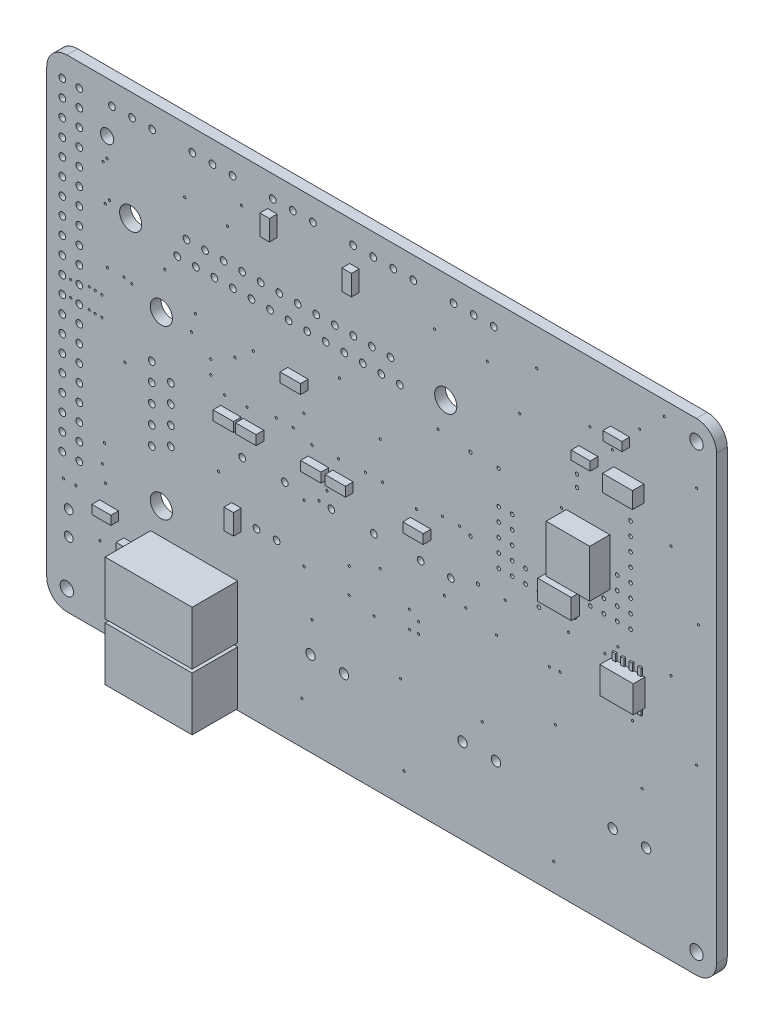
SolidWorks part; units mm, degrees
ref_plane "Front Plane" through (0, 0, 0) normal (0, 0, 1) x (1, 0, 0)
ref_plane "Top Plane" through (0, 0, 0) normal (0, 1, 0) x (1, 0, 0)
ref_plane "Right Plane" through (0, 0, 0) normal (1, 0, 0) x (0, 0, -1)
sketch "121" plane through (0, 0, 0) normal (0, 0, 1) x (1, 0, 0)
  line L0 (8, 71.008) -> (17.5, 71.008)
  line L1 (17.5, 71.008) -> (17.5, 67.524)
  line L2 (17.5, 67.524) -> (8, 67.524)
  line L3 (8, 67.524) -> (8, 71.008)
  line L4 (19.938, 71.008) -> (29.438, 71.008)
  line L5 (29.438, 71.008) -> (29.438, 67.524)
  line L6 (29.438, 67.524) -> (19.938, 67.524)
  line L7 (19.938, 67.524) -> (19.938, 71.008)
  line L8 (31.876, 71.008) -> (41.376, 71.008)
  line L9 (41.376, 71.008) -> (41.376, 67.524)
  line L10 (41.376, 67.524) -> (31.876, 67.524)
  line L11 (31.876, 67.524) -> (31.876, 71.008)
  line L12 (59.054, 71.008) -> (68.554, 71.008)
  line L13 (68.554, 71.008) -> (68.554, 67.524)
  line L14 (68.554, 67.524) -> (59.054, 67.524)
  line L15 (59.054, 67.524) -> (59.054, 71.008)
  line L16 (44.322, 71.008) -> (56.108, 71.008)
  line L17 (56.108, 71.008) -> (56.108, 67.524)
  line L18 (56.108, 67.524) -> (44.322, 67.524)
  line L19 (44.322, 67.524) -> (44.322, 71.008)
  line L20 (50.292, 67.564) -> (50.292, 68.715)
  line L21 (50.292, 69.715) -> (50.292, 70.866)
  line L22 (27.686, 34.544) -> (37.084, 34.544)
  line L23 (37.084, 34.544) -> (37.084, 29.464)
  line L24 (37.084, 29.464) -> (27.686, 29.464)
  line L25 (27.686, 29.464) -> (27.686, 34.544)
  line L26 (41.148, 34.544) -> (50.292, 34.544)
  line L27 (50.292, 34.544) -> (50.292, 29.464)
  line L28 (50.292, 29.464) -> (41.148, 29.464)
  line L29 (41.148, 29.464) -> (41.148, 34.544)
  line L30 (54.102, 34.544) -> (61.976, 34.544)
  line L31 (61.976, 34.544) -> (61.976, 29.464)
  line L32 (61.976, 29.464) -> (54.102, 29.464)
  line L33 (54.102, 29.464) -> (54.102, 34.544)
  line L34 (29.8704, 27.5336) -> (35.814, 27.5336)
  line L35 (35.814, 27.5336) -> (35.814, 22.2758)
  line L36 (35.814, 22.2758) -> (29.8704, 22.2758)
  line L37 (29.8704, 22.2758) -> (29.8704, 27.5336)
  line L38 (0.0254, 16.637) -> (5.3086, 16.637)
  line L39 (5.3086, 16.637) -> (5.3086, 6.5278)
  line L40 (5.3086, 6.5278) -> (0.0254, 6.5278)
  line L41 (0.0254, 6.5278) -> (0.0254, 16.637)
  line L42 (11.7667, 71.648) -> (11.7667, 71.2667)
  line L43 (11.7667, 71.2667) -> (11.9574, 71.2667)
  line L44 (11.9574, 71.2667) -> (12.0209, 71.3303)
  line L45 (12.0209, 71.3303) -> (12.0209, 71.5845)
  line L46 (12.0209, 71.5845) -> (11.9574, 71.648)
  line L47 (11.9574, 71.648) -> (11.7667, 71.648)
  line L48 (12.1409, 71.2667) -> (12.1409, 71.648)
  line L49 (12.1409, 71.4574) -> (12.3951, 71.4574)
  line L50 (12.3951, 71.648) -> (12.3951, 71.2667)
  line L51 (12.6422, 71.2667) -> (12.6422, 71.648)
  line L52 (12.5151, 71.648) -> (12.7693, 71.648)
  line L53 (12.8893, 71.4574) -> (13.1435, 71.4574)
  line L54 (13.2635, 71.2667) -> (13.3906, 71.2667)
  line L55 (13.3271, 71.2667) -> (13.3271, 71.648)
  line L56 (13.2635, 71.648) -> (13.3906, 71.648)
  line L57 (13.513, 71.2667) -> (13.513, 71.648)
  line L58 (13.513, 71.648) -> (13.7672, 71.2667)
  line L59 (13.7672, 71.2667) -> (13.7672, 71.648)
  line L60 (14.0143, 71.2667) -> (14.0143, 71.648)
  line L61 (13.8872, 71.648) -> (14.1414, 71.648)
  line L62 (9.2841, 70.4547) -> (9.7756, 70.4547)
  line L63 (9.5298, 70.7005) -> (9.5298, 70.209)
  line L64 (12.5903, 70.5955) -> (12.497, 70.6887)
  line L65 (12.497, 70.6887) -> (12.3106, 70.6887)
  line L66 (12.3106, 70.6887) -> (12.2174, 70.5955)
  line L67 (12.2174, 70.5955) -> (12.2174, 70.5023)
  line L68 (12.2174, 70.5023) -> (12.3106, 70.409)
  line L69 (12.3106, 70.409) -> (12.497, 70.409)
  line L70 (12.497, 70.409) -> (12.5903, 70.3158)
  line L71 (12.5903, 70.3158) -> (12.5903, 70.2226)
  line L72 (12.5903, 70.2226) -> (12.497, 70.1294)
  line L73 (12.497, 70.1294) -> (12.3106, 70.1294)
  line L74 (12.3106, 70.1294) -> (12.2174, 70.2226)
  line L75 (12.7787, 70.1294) -> (12.9651, 70.1294)
  line L76 (12.8719, 70.1294) -> (12.8719, 70.6887)
  line L77 (12.7787, 70.6887) -> (12.9651, 70.6887)
  line L78 (13.5258, 70.5955) -> (13.4326, 70.6887)
  line L79 (13.4326, 70.6887) -> (13.2461, 70.6887)
  line L80 (13.2461, 70.6887) -> (13.1529, 70.5955)
  line L81 (13.1529, 70.5955) -> (13.1529, 70.2226)
  line L82 (13.1529, 70.2226) -> (13.2461, 70.1294)
  line L83 (13.2461, 70.1294) -> (13.4326, 70.1294)
  line L84 (13.4326, 70.1294) -> (13.5258, 70.2226)
  line L85 (13.5258, 70.2226) -> (13.5258, 70.409)
  line L86 (13.5258, 70.409) -> (13.3393, 70.409)
  line L87 (15.5448, 70.4855) -> (16.3244, 70.4855)
  line L88 (23.7047, 71.648) -> (23.7047, 71.2667)
  line L89 (23.7047, 71.2667) -> (23.8954, 71.2667)
  line L90 (23.8954, 71.2667) -> (23.9589, 71.3303)
  line L91 (23.9589, 71.3303) -> (23.9589, 71.5845)
  line L92 (23.9589, 71.5845) -> (23.8954, 71.648)
  line L93 (23.8954, 71.648) -> (23.7047, 71.648)
  line L94 (24.0789, 71.2667) -> (24.0789, 71.648)
  line L95 (24.0789, 71.4574) -> (24.3331, 71.4574)
  line L96 (24.3331, 71.648) -> (24.3331, 71.2667)
  line L97 (24.5802, 71.2667) -> (24.5802, 71.648)
  line L98 (24.4531, 71.648) -> (24.7073, 71.648)
  line L99 (24.8273, 71.4574) -> (25.0815, 71.4574)
  line L100 (25.4557, 71.648) -> (25.2015, 71.648)
  line L101 (25.2015, 71.648) -> (25.2015, 71.2667)
  line L102 (25.2015, 71.2667) -> (25.4557, 71.2667)
  line L103 (25.2015, 71.4574) -> (25.3286, 71.4574)
  line L104 (25.5757, 71.648) -> (25.8299, 71.2667)
  line L105 (25.8299, 71.648) -> (25.5757, 71.2667)
  line L106 (26.077, 71.2667) -> (26.077, 71.648)
  line L107 (25.9499, 71.648) -> (26.2042, 71.648)
  line L108 (21.4761, 70.4547) -> (21.9676, 70.4547)
  line L109 (21.7218, 70.7005) -> (21.7218, 70.209)
  line L110 (24.5282, 70.5955) -> (24.435, 70.6887)
  line L111 (24.435, 70.6887) -> (24.2486, 70.6887)
  line L112 (24.2486, 70.6887) -> (24.1554, 70.5955)
  line L113 (24.1554, 70.5955) -> (24.1554, 70.5023)
  line L114 (24.1554, 70.5023) -> (24.2486, 70.409)
  line L115 (24.2486, 70.409) -> (24.435, 70.409)
  line L116 (24.435, 70.409) -> (24.5282, 70.3158)
  line L117 (24.5282, 70.3158) -> (24.5282, 70.2226)
  line L118 (24.5282, 70.2226) -> (24.435, 70.1294)
  line L119 (24.435, 70.1294) -> (24.2486, 70.1294)
  line L120 (24.2486, 70.1294) -> (24.1554, 70.2226)
  line L121 (24.7167, 70.1294) -> (24.9031, 70.1294)
  line L122 (24.8099, 70.1294) -> (24.8099, 70.6887)
  line L123 (24.7167, 70.6887) -> (24.9031, 70.6887)
  line L124 (25.4638, 70.5955) -> (25.3706, 70.6887)
  line L125 (25.3706, 70.6887) -> (25.1841, 70.6887)
  line L126 (25.1841, 70.6887) -> (25.0909, 70.5955)
  line L127 (25.0909, 70.5955) -> (25.0909, 70.2226)
  line L128 (25.0909, 70.2226) -> (25.1841, 70.1294)
  line L129 (25.1841, 70.1294) -> (25.3706, 70.1294)
  line L130 (25.3706, 70.1294) -> (25.4638, 70.2226)
  line L131 (25.4638, 70.2226) -> (25.4638, 70.409)
  line L132 (25.4638, 70.409) -> (25.2773, 70.409)
  line L133 (27.4828, 70.4855) -> (28.2624, 70.4855)
  line L134 (36.1509, 71.5845) -> (36.0874, 71.648)
  line L135 (36.0874, 71.648) -> (35.9603, 71.648)
  line L136 (35.9603, 71.648) -> (35.8967, 71.5845)
  line L137 (35.8967, 71.5845) -> (35.8967, 71.5209)
  line L138 (35.8967, 71.5209) -> (35.9603, 71.4574)
  line L139 (35.9603, 71.4574) -> (36.0874, 71.4574)
  line L140 (36.0874, 71.4574) -> (36.1509, 71.3938)
  line L141 (36.1509, 71.3938) -> (36.1509, 71.3303)
  line L142 (36.1509, 71.3303) -> (36.0874, 71.2667)
  line L143 (36.0874, 71.2667) -> (35.9603, 71.2667)
  line L144 (35.9603, 71.2667) -> (35.8967, 71.3303)
  line L145 (36.5251, 71.648) -> (36.2709, 71.648)
  line L146 (36.2709, 71.648) -> (36.2709, 71.2667)
  line L147 (36.2709, 71.2667) -> (36.5251, 71.2667)
  line L148 (36.2709, 71.4574) -> (36.398, 71.4574)
  line L149 (36.6451, 71.2667) -> (36.6451, 71.648)
  line L150 (36.6451, 71.648) -> (36.8358, 71.648)
  line L151 (36.8358, 71.648) -> (36.8993, 71.5845)
  line L152 (36.8993, 71.5845) -> (36.8993, 71.4574)
  line L153 (36.8993, 71.4574) -> (36.8358, 71.3938)
  line L154 (36.8358, 71.3938) -> (36.6451, 71.3938)
  line L155 (36.7722, 71.3938) -> (36.8993, 71.2667)
  line L156 (37.0193, 71.648) -> (37.0193, 71.3938)
  line L157 (37.0193, 71.3938) -> (37.1464, 71.2667)
  line L158 (37.1464, 71.2667) -> (37.2735, 71.3938)
  line L159 (37.2735, 71.3938) -> (37.2735, 71.648)
  line L160 (37.5842, 71.648) -> (37.4571, 71.648)
  line L161 (37.4571, 71.648) -> (37.3935, 71.5845)
  line L162 (37.3935, 71.5845) -> (37.3935, 71.3303)
  line L163 (37.3935, 71.3303) -> (37.4571, 71.2667)
  line L164 (37.4571, 71.2667) -> (37.5842, 71.2667)
  line L165 (37.5842, 71.2667) -> (37.6477, 71.3303)
  line L166 (37.6477, 71.3303) -> (37.6477, 71.5845)
  line L167 (37.6477, 71.5845) -> (37.5842, 71.648)
  line L168 (33.4141, 70.4547) -> (33.9056, 70.4547)
  line L169 (33.6598, 70.7005) -> (33.6598, 70.209)
  line L170 (35.8394, 70.1294) -> (35.8394, 70.6887)
  line L171 (35.8394, 70.6887) -> (36.119, 70.6887)
  line L172 (36.119, 70.6887) -> (36.2123, 70.5955)
  line L173 (36.2123, 70.5955) -> (36.2123, 70.409)
  line L174 (36.2123, 70.409) -> (36.119, 70.3158)
  line L175 (36.119, 70.3158) -> (35.8394, 70.3158)
  line L176 (36.4007, 70.6887) -> (36.4007, 70.1294)
  line L177 (36.4007, 70.1294) -> (36.5871, 70.3158)
  line L178 (36.5871, 70.3158) -> (36.7736, 70.1294)
  line L179 (36.7736, 70.1294) -> (36.7736, 70.6887)
  line L180 (36.962, 70.1294) -> (36.962, 70.6887)
  line L181 (36.962, 70.6887) -> (37.1484, 70.5023)
  line L182 (37.1484, 70.5023) -> (37.3349, 70.6887)
  line L183 (37.3349, 70.6887) -> (37.3349, 70.1294)
  line L184 (39.4208, 70.4855) -> (40.2004, 70.4855)
  line L185 (62.0587, 71.648) -> (62.0587, 71.2667)
  line L186 (62.0587, 71.2667) -> (62.3129, 71.2667)
  line L187 (62.4329, 71.2667) -> (62.56, 71.2667)
  line L188 (62.4965, 71.2667) -> (62.4965, 71.648)
  line L189 (62.4329, 71.648) -> (62.56, 71.648)
  line L190 (62.9366, 71.5845) -> (62.873, 71.648)
  line L191 (62.873, 71.648) -> (62.7459, 71.648)
  line L192 (62.7459, 71.648) -> (62.6824, 71.5845)
  line L193 (62.6824, 71.5845) -> (62.6824, 71.3303)
  line L194 (62.6824, 71.3303) -> (62.7459, 71.2667)
  line L195 (62.7459, 71.2667) -> (62.873, 71.2667)
  line L196 (62.873, 71.2667) -> (62.9366, 71.3303)
  line L197 (62.9366, 71.3303) -> (62.9366, 71.4574)
  line L198 (62.9366, 71.4574) -> (62.8095, 71.4574)
  line L199 (63.0566, 71.2667) -> (63.0566, 71.648)
  line L200 (63.0566, 71.4574) -> (63.3108, 71.4574)
  line L201 (63.3108, 71.648) -> (63.3108, 71.2667)
  line L202 (63.5579, 71.2667) -> (63.5579, 71.648)
  line L203 (63.4308, 71.648) -> (63.685, 71.648)
  line L204 (64.4334, 71.5845) -> (64.3699, 71.648)
  line L205 (64.3699, 71.648) -> (64.2428, 71.648)
  line L206 (64.2428, 71.648) -> (64.1792, 71.5845)
  line L207 (64.1792, 71.5845) -> (64.1792, 71.5209)
  line L208 (64.1792, 71.5209) -> (64.2428, 71.4574)
  line L209 (64.2428, 71.4574) -> (64.3699, 71.4574)
  line L210 (64.3699, 71.4574) -> (64.4334, 71.3938)
  line L211 (64.4334, 71.3938) -> (64.4334, 71.3303)
  line L212 (64.4334, 71.3303) -> (64.3699, 71.2667)
  line L213 (64.3699, 71.2667) -> (64.2428, 71.2667)
  line L214 (64.2428, 71.2667) -> (64.1792, 71.3303)
  line L215 (64.8076, 71.648) -> (64.5534, 71.648)
  line L216 (64.5534, 71.648) -> (64.5534, 71.2667)
  line L217 (64.5534, 71.2667) -> (64.8076, 71.2667)
  line L218 (64.5534, 71.4574) -> (64.6805, 71.4574)
  line L219 (64.9276, 71.2667) -> (64.9276, 71.648)
  line L220 (64.9276, 71.648) -> (65.1818, 71.2667)
  line L221 (65.1818, 71.2667) -> (65.1818, 71.648)
  line L222 (65.556, 71.5845) -> (65.4925, 71.648)
  line L223 (65.4925, 71.648) -> (65.3654, 71.648)
  line L224 (65.3654, 71.648) -> (65.3018, 71.5845)
  line L225 (65.3018, 71.5845) -> (65.3018, 71.5209)
  line L226 (65.3018, 71.5209) -> (65.3654, 71.4574)
  line L227 (65.3654, 71.4574) -> (65.4925, 71.4574)
  line L228 (65.4925, 71.4574) -> (65.556, 71.3938)
  line L229 (65.556, 71.3938) -> (65.556, 71.3303)
  line L230 (65.556, 71.3303) -> (65.4925, 71.2667)
  line L231 (65.4925, 71.2667) -> (65.3654, 71.2667)
  line L232 (65.3654, 71.2667) -> (65.3018, 71.3303)
  line L233 (65.8667, 71.648) -> (65.7396, 71.648)
  line L234 (65.7396, 71.648) -> (65.676, 71.5845)
  line L235 (65.676, 71.5845) -> (65.676, 71.3303)
  line L236 (65.676, 71.3303) -> (65.7396, 71.2667)
  line L237 (65.7396, 71.2667) -> (65.8667, 71.2667)
  line L238 (65.8667, 71.2667) -> (65.9302, 71.3303)
  line L239 (65.9302, 71.3303) -> (65.9302, 71.5845)
  line L240 (65.9302, 71.5845) -> (65.8667, 71.648)
  line L241 (66.0502, 71.2667) -> (66.0502, 71.648)
  line L242 (66.0502, 71.648) -> (66.2409, 71.648)
  line L243 (66.2409, 71.648) -> (66.3045, 71.5845)
  line L244 (66.3045, 71.5845) -> (66.3045, 71.4574)
  line L245 (66.3045, 71.4574) -> (66.2409, 71.3938)
  line L246 (66.2409, 71.3938) -> (66.0502, 71.3938)
  line L247 (66.1773, 71.3938) -> (66.3045, 71.2667)
  line L248 (60.3381, 70.4547) -> (60.8296, 70.4547)
  line L249 (60.5838, 70.7005) -> (60.5838, 70.209)
  line L250 (63.6442, 70.5955) -> (63.551, 70.6887)
  line L251 (63.551, 70.6887) -> (63.3646, 70.6887)
  line L252 (63.3646, 70.6887) -> (63.2714, 70.5955)
  line L253 (63.2714, 70.5955) -> (63.2714, 70.5023)
  line L254 (63.2714, 70.5023) -> (63.3646, 70.409)
  line L255 (63.3646, 70.409) -> (63.551, 70.409)
  line L256 (63.551, 70.409) -> (63.6442, 70.3158)
  line L257 (63.6442, 70.3158) -> (63.6442, 70.2226)
  line L258 (63.6442, 70.2226) -> (63.551, 70.1294)
  line L259 (63.551, 70.1294) -> (63.3646, 70.1294)
  line L260 (63.3646, 70.1294) -> (63.2714, 70.2226)
  line L261 (63.8327, 70.1294) -> (64.0191, 70.1294)
  line L262 (63.9259, 70.1294) -> (63.9259, 70.6887)
  line L263 (63.8327, 70.6887) -> (64.0191, 70.6887)
  line L264 (64.5798, 70.5955) -> (64.4866, 70.6887)
  line L265 (64.4866, 70.6887) -> (64.3001, 70.6887)
  line L266 (64.3001, 70.6887) -> (64.2069, 70.5955)
  line L267 (64.2069, 70.5955) -> (64.2069, 70.2226)
  line L268 (64.2069, 70.2226) -> (64.3001, 70.1294)
  line L269 (64.3001, 70.1294) -> (64.4866, 70.1294)
  line L270 (64.4866, 70.1294) -> (64.5798, 70.2226)
  line L271 (64.5798, 70.2226) -> (64.5798, 70.409)
  line L272 (64.5798, 70.409) -> (64.3933, 70.409)
  line L273 (66.5988, 70.4855) -> (67.3784, 70.4855)
  line L274 (48.5588, 71.5972) -> (48.4317, 71.5972)
  line L275 (48.4317, 71.5972) -> (48.3681, 71.5337)
  line L276 (48.3681, 71.5337) -> (48.3681, 71.2795)
  line L277 (48.3681, 71.2795) -> (48.4317, 71.2159)
  line L278 (48.4317, 71.2159) -> (48.5588, 71.2159)
  line L279 (48.5588, 71.2159) -> (48.6223, 71.2795)
  line L280 (48.6223, 71.2795) -> (48.6223, 71.5337)
  line L281 (48.6223, 71.5337) -> (48.5588, 71.5972)
  line L282 (48.7423, 71.2159) -> (48.7423, 71.5972)
  line L283 (48.7423, 71.5972) -> (48.933, 71.5972)
  line L284 (48.933, 71.5972) -> (48.9965, 71.5337)
  line L285 (48.9965, 71.5337) -> (48.9965, 71.4066)
  line L286 (48.9965, 71.4066) -> (48.933, 71.343)
  line L287 (48.933, 71.343) -> (48.7423, 71.343)
  line L288 (49.2436, 71.2159) -> (49.2436, 71.5972)
  line L289 (49.1165, 71.5972) -> (49.3707, 71.5972)
  line L290 (49.4907, 71.2159) -> (49.6178, 71.2159)
  line L291 (49.5543, 71.2159) -> (49.5543, 71.5972)
  line L292 (49.4907, 71.5972) -> (49.6178, 71.5972)
  line L293 (49.9944, 71.5337) -> (49.9309, 71.5972)
  line L294 (49.9309, 71.5972) -> (49.8037, 71.5972)
  line L295 (49.8037, 71.5972) -> (49.7402, 71.5337)
  line L296 (49.7402, 71.5337) -> (49.7402, 71.2795)
  line L297 (49.7402, 71.2795) -> (49.8037, 71.2159)
  line L298 (49.8037, 71.2159) -> (49.9309, 71.2159)
  line L299 (49.9309, 71.2159) -> (49.9944, 71.2795)
  line L300 (50.1144, 71.2159) -> (50.1144, 71.4701)
  line L301 (50.1144, 71.4701) -> (50.2415, 71.5972)
  line L302 (50.2415, 71.5972) -> (50.3686, 71.4701)
  line L303 (50.3686, 71.4701) -> (50.3686, 71.2159)
  line L304 (50.1144, 71.4066) -> (50.3686, 71.4066)
  line L305 (50.4886, 71.5972) -> (50.4886, 71.2159)
  line L306 (50.4886, 71.2159) -> (50.7428, 71.2159)
  line L307 (51.237, 71.2159) -> (51.237, 71.5972)
  line L308 (51.237, 71.5972) -> (51.4912, 71.5972)
  line L309 (51.237, 71.4066) -> (51.3641, 71.4066)
  line L310 (51.8019, 71.5972) -> (51.6748, 71.5972)
  line L311 (51.6748, 71.5972) -> (51.6112, 71.5337)
  line L312 (51.6112, 71.5337) -> (51.6112, 71.2795)
  line L313 (51.6112, 71.2795) -> (51.6748, 71.2159)
  line L314 (51.6748, 71.2159) -> (51.8019, 71.2159)
  line L315 (51.8019, 71.2159) -> (51.8654, 71.2795)
  line L316 (51.8654, 71.2795) -> (51.8654, 71.5337)
  line L317 (51.8654, 71.5337) -> (51.8019, 71.5972)
  line L318 (51.9854, 71.2159) -> (51.9854, 71.5972)
  line L319 (51.9854, 71.5972) -> (52.1761, 71.5972)
  line L320 (52.1761, 71.5972) -> (52.2396, 71.5337)
  line L321 (52.2396, 71.5337) -> (52.2396, 71.4066)
  line L322 (52.2396, 71.4066) -> (52.1761, 71.343)
  line L323 (52.1761, 71.343) -> (51.9854, 71.343)
  line L324 (52.1125, 71.343) -> (52.2396, 71.2159)
  line L325 (52.3596, 71.5972) -> (52.3596, 71.2159)
  line L326 (52.3596, 71.343) -> (52.6138, 71.5972)
  line L327 (52.4232, 71.4066) -> (52.6138, 71.2159)
  line L328 (45.3521, 70.4547) -> (45.8436, 70.4547)
  line L329 (45.5978, 70.7005) -> (45.5978, 70.209)
  line L330 (48.5648, 70.4855) -> (49.3444, 70.4855)
  line L331 (51.3461, 70.5107) -> (51.8376, 70.5107)
  line L332 (51.5918, 70.7565) -> (51.5918, 70.265)
  line L333 (54.7543, 70.5955) -> (54.661, 70.6887)
  line L334 (54.661, 70.6887) -> (54.4746, 70.6887)
  line L335 (54.4746, 70.6887) -> (54.3814, 70.5955)
  line L336 (54.3814, 70.5955) -> (54.3814, 70.5023)
  line L337 (54.3814, 70.5023) -> (54.4746, 70.409)
  line L338 (54.4746, 70.409) -> (54.661, 70.409)
  line L339 (54.661, 70.409) -> (54.7543, 70.3158)
  line L340 (54.7543, 70.3158) -> (54.7543, 70.2226)
  line L341 (54.7543, 70.2226) -> (54.661, 70.1294)
  line L342 (54.661, 70.1294) -> (54.4746, 70.1294)
  line L343 (54.4746, 70.1294) -> (54.3814, 70.2226)
  line L344 (54.9427, 70.1294) -> (55.1291, 70.1294)
  line L345 (55.0359, 70.1294) -> (55.0359, 70.6887)
  line L346 (54.9427, 70.6887) -> (55.1291, 70.6887)
  line L347 (55.6898, 70.5955) -> (55.5966, 70.6887)
  line L348 (55.5966, 70.6887) -> (55.4101, 70.6887)
  line L349 (55.4101, 70.6887) -> (55.3169, 70.5955)
  line L350 (55.3169, 70.5955) -> (55.3169, 70.2226)
  line L351 (55.3169, 70.2226) -> (55.4101, 70.1294)
  line L352 (55.4101, 70.1294) -> (55.5966, 70.1294)
  line L353 (55.5966, 70.1294) -> (55.6898, 70.2226)
  line L354 (55.6898, 70.2226) -> (55.6898, 70.409)
  line L355 (55.6898, 70.409) -> (55.5033, 70.409)
  line L356 (47.0029, 70.752) -> (46.7487, 70.752)
  line L357 (46.7487, 70.752) -> (46.7487, 70.3707)
  line L358 (46.7487, 70.3707) -> (47.0029, 70.3707)
  line L359 (46.7487, 70.5614) -> (46.8758, 70.5614)
  line L360 (47.1229, 70.3707) -> (47.1229, 70.752)
  line L361 (47.1229, 70.752) -> (47.25, 70.6249)
  line L362 (47.25, 70.6249) -> (47.3771, 70.752)
  line L363 (47.3771, 70.752) -> (47.3771, 70.3707)
  line L364 (47.4971, 70.3707) -> (47.6242, 70.3707)
  line L365 (47.5607, 70.3707) -> (47.5607, 70.752)
  line L366 (47.4971, 70.752) -> (47.6242, 70.752)
  line L367 (47.8737, 70.3707) -> (47.8737, 70.752)
  line L368 (47.7466, 70.752) -> (48.0008, 70.752)
  line L369 (52.5907, 70.3707) -> (52.5907, 70.752)
  line L370 (52.5907, 70.752) -> (52.7814, 70.752)
  line L371 (52.7814, 70.752) -> (52.8449, 70.6885)
  line L372 (52.8449, 70.6885) -> (52.8449, 70.5614)
  line L373 (52.8449, 70.5614) -> (52.7814, 70.4978)
  line L374 (52.7814, 70.4978) -> (52.5907, 70.4978)
  line L375 (52.7178, 70.4978) -> (52.8449, 70.3707)
  line L376 (53.2191, 70.752) -> (52.9649, 70.752)
  line L377 (52.9649, 70.752) -> (52.9649, 70.3707)
  line L378 (52.9649, 70.3707) -> (53.2191, 70.3707)
  line L379 (52.9649, 70.5614) -> (53.092, 70.5614)
  line L380 (53.5933, 70.6885) -> (53.5298, 70.752)
  line L381 (53.5298, 70.752) -> (53.4027, 70.752)
  line L382 (53.4027, 70.752) -> (53.3391, 70.6885)
  line L383 (53.3391, 70.6885) -> (53.3391, 70.4343)
  line L384 (53.3391, 70.4343) -> (53.4027, 70.3707)
  line L385 (53.4027, 70.3707) -> (53.5298, 70.3707)
  line L386 (53.5298, 70.3707) -> (53.5933, 70.4343)
  line L387 (31.0961, 29.8901) -> (31.0961, 30.6273)
  line L388 (31.0961, 30.2587) -> (31.5876, 30.2587)
  line L389 (31.5876, 30.6273) -> (31.5876, 29.8901)
  line L390 (32.336, 30.6273) -> (31.8445, 30.6273)
  line L391 (31.8445, 30.6273) -> (31.8445, 29.8901)
  line L392 (31.8445, 29.8901) -> (32.336, 29.8901)
  line L393 (31.8445, 30.2587) -> (32.0903, 30.2587)
  line L394 (32.5929, 29.8901) -> (32.5929, 30.3816)
  line L395 (32.5929, 30.3816) -> (32.8387, 30.6273)
  line L396 (32.8387, 30.6273) -> (33.0844, 30.3816)
  line L397 (33.0844, 30.3816) -> (33.0844, 29.8901)
  line L398 (32.5929, 30.2587) -> (33.0844, 30.2587)
  line L399 (33.5871, 29.8901) -> (33.5871, 30.6273)
  line L400 (33.3413, 30.6273) -> (33.8328, 30.6273)
  line L401 (34.9508, 31.0595) -> (35.7304, 31.0595)
  line L402 (35.3406, 31.4493) -> (35.3406, 30.6697)
  line L403 (28.7655, 31.0649) -> (29.7993, 31.0649)
  line L404 (43.7961, 30.6273) -> (43.7961, 29.8901)
  line L405 (43.7961, 29.8901) -> (44.1647, 29.8901)
  line L406 (44.1647, 29.8901) -> (44.2876, 30.013)
  line L407 (44.2876, 30.013) -> (44.2876, 30.5045)
  line L408 (44.2876, 30.5045) -> (44.1647, 30.6273)
  line L409 (44.1647, 30.6273) -> (43.7961, 30.6273)
  line L410 (45.036, 30.6273) -> (44.5445, 30.6273)
  line L411 (44.5445, 30.6273) -> (44.5445, 29.8901)
  line L412 (44.5445, 29.8901) -> (45.036, 29.8901)
  line L413 (44.5445, 30.2587) -> (44.7903, 30.2587)
  line L414 (45.2929, 29.8901) -> (45.2929, 30.6273)
  line L415 (45.2929, 30.2587) -> (45.7844, 30.2587)
  line L416 (45.7844, 30.6273) -> (45.7844, 29.8901)
  line L417 (46.0413, 30.6273) -> (46.0413, 30.013)
  line L418 (46.0413, 30.013) -> (46.1642, 29.8901)
  line L419 (46.1642, 29.8901) -> (46.41, 29.8901)
  line L420 (46.41, 29.8901) -> (46.5328, 30.013)
  line L421 (46.5328, 30.013) -> (46.5328, 30.6273)
  line L422 (46.7898, 29.8901) -> (46.7898, 30.6273)
  line L423 (46.7898, 30.6273) -> (47.0355, 30.3816)
  line L424 (47.0355, 30.3816) -> (47.2812, 30.6273)
  line L425 (47.2812, 30.6273) -> (47.2812, 29.8901)
  line L426 (48.4128, 31.0595) -> (49.1924, 31.0595)
  line L427 (48.8026, 31.4493) -> (48.8026, 30.6697)
  line L428 (42.2275, 31.0649) -> (43.2613, 31.0649)
  line L429 (57.2581, 29.8901) -> (57.2581, 30.6273)
  line L430 (57.2581, 30.6273) -> (57.7496, 30.6273)
  line L431 (57.2581, 30.2587) -> (57.5038, 30.2587)
  line L432 (58.0065, 29.8901) -> (58.0065, 30.3816)
  line L433 (58.0065, 30.3816) -> (58.2523, 30.6273)
  line L434 (58.2523, 30.6273) -> (58.498, 30.3816)
  line L435 (58.498, 30.3816) -> (58.498, 29.8901)
  line L436 (58.0065, 30.2587) -> (58.498, 30.2587)
  line L437 (58.7549, 29.8901) -> (58.7549, 30.6273)
  line L438 (58.7549, 30.6273) -> (59.2464, 29.8901)
  line L439 (59.2464, 29.8901) -> (59.2464, 30.6273)
  line L440 (59.8428, 31.0595) -> (60.6224, 31.0595)
  line L441 (60.2326, 31.4493) -> (60.2326, 30.6697)
  line L442 (55.4355, 31.0649) -> (56.4693, 31.0649)
  line L443 (34.2389, 39.0525) -> (34.2389, 39.544)
  line L444 (33.9931, 39.2982) -> (34.4846, 39.2982)
  line L445 (33.8703, 40.2924) -> (33.8703, 39.8009)
  line L446 (33.8703, 39.8009) -> (34.2389, 39.8009)
  line L447 (34.2389, 39.8009) -> (34.116, 40.0467)
  line L448 (34.116, 40.0467) -> (34.116, 40.1695)
  line L449 (34.116, 40.1695) -> (34.2389, 40.2924)
  line L450 (34.2389, 40.2924) -> (34.4846, 40.2924)
  line L451 (34.4846, 40.2924) -> (34.6075, 40.1695)
  line L452 (34.6075, 40.1695) -> (34.6075, 39.9238)
  line L453 (34.6075, 39.9238) -> (34.4846, 39.8009)
  line L454 (33.8703, 40.5493) -> (34.3618, 40.5493)
  line L455 (34.3618, 40.5493) -> (34.6075, 40.7951)
  line L456 (34.6075, 40.7951) -> (34.3618, 41.0408)
  line L457 (34.3618, 41.0408) -> (33.8703, 41.0408)
  line L458 (36.7281, 39.0271) -> (36.7281, 39.5186)
  line L459 (36.4823, 39.2728) -> (36.9738, 39.2728)
  line L460 (36.6052, 39.7755) -> (36.3595, 40.0213)
  line L461 (36.3595, 40.0213) -> (37.0967, 40.0213)
  line L462 (37.0967, 39.7755) -> (37.0967, 40.267)
  line L463 (37.0967, 41.0154) -> (37.0967, 40.5239)
  line L464 (37.0967, 40.5239) -> (36.6052, 41.0154)
  line L465 (36.6052, 41.0154) -> (36.4823, 41.0154)
  line L466 (36.4823, 41.0154) -> (36.3595, 40.8925)
  line L467 (36.3595, 40.8925) -> (36.3595, 40.6468)
  line L468 (36.3595, 40.6468) -> (36.4823, 40.5239)
  line L469 (36.3595, 41.2723) -> (36.851, 41.2723)
  line L470 (36.851, 41.2723) -> (37.0967, 41.5181)
  line L471 (37.0967, 41.5181) -> (36.851, 41.7638)
  line L472 (36.851, 41.7638) -> (36.3595, 41.7638)
  line L473 (50.0885, 38.7223) -> (50.0885, 39.2138)
  line L474 (49.8427, 38.968) -> (50.3342, 38.968)
  line L475 (49.9656, 39.4707) -> (49.7199, 39.7165)
  line L476 (49.7199, 39.7165) -> (50.4571, 39.7165)
  line L477 (50.4571, 39.4707) -> (50.4571, 39.9622)
  line L478 (50.4571, 40.7106) -> (50.4571, 40.2191)
  line L479 (50.4571, 40.2191) -> (49.9656, 40.7106)
  line L480 (49.9656, 40.7106) -> (49.8427, 40.7106)
  line L481 (49.8427, 40.7106) -> (49.7199, 40.5877)
  line L482 (49.7199, 40.5877) -> (49.7199, 40.342)
  line L483 (49.7199, 40.342) -> (49.8427, 40.2191)
  line L484 (49.7199, 40.9675) -> (50.2114, 40.9675)
  line L485 (50.2114, 40.9675) -> (50.4571, 41.2133)
  line L486 (50.4571, 41.2133) -> (50.2114, 41.459)
  line L487 (50.2114, 41.459) -> (49.7199, 41.459)
  line L488 (61.5947, 38.6461) -> (61.5947, 39.1376)
  line L489 (61.3489, 38.8918) -> (61.8404, 38.8918)
  line L490 (61.4718, 39.3945) -> (61.2261, 39.6403)
  line L491 (61.2261, 39.6403) -> (61.9633, 39.6403)
  line L492 (61.9633, 39.3945) -> (61.9633, 39.886)
  line L493 (61.9633, 40.6344) -> (61.9633, 40.1429)
  line L494 (61.9633, 40.1429) -> (61.4718, 40.6344)
  line L495 (61.4718, 40.6344) -> (61.3489, 40.6344)
  line L496 (61.3489, 40.6344) -> (61.2261, 40.5115)
  line L497 (61.2261, 40.5115) -> (61.2261, 40.2658)
  line L498 (61.2261, 40.2658) -> (61.3489, 40.1429)
  line L499 (61.2261, 40.8913) -> (61.7176, 40.8913)
  line L500 (61.7176, 40.8913) -> (61.9633, 41.1371)
  line L501 (61.9633, 41.1371) -> (61.7176, 41.3828)
  line L502 (61.7176, 41.3828) -> (61.2261, 41.3828)
  line L503 (59.0547, 38.6715) -> (59.0547, 39.163)
  line L504 (58.8089, 38.9172) -> (59.3004, 38.9172)
  line L505 (58.6861, 39.9114) -> (58.6861, 39.4199)
  line L506 (58.6861, 39.4199) -> (59.0547, 39.4199)
  line L507 (59.0547, 39.4199) -> (58.9318, 39.6657)
  line L508 (58.9318, 39.6657) -> (58.9318, 39.7885)
  line L509 (58.9318, 39.7885) -> (59.0547, 39.9114)
  line L510 (59.0547, 39.9114) -> (59.3004, 39.9114)
  line L511 (59.3004, 39.9114) -> (59.4233, 39.7885)
  line L512 (59.4233, 39.7885) -> (59.4233, 39.5428)
  line L513 (59.4233, 39.5428) -> (59.3004, 39.4199)
  line L514 (58.6861, 40.1683) -> (59.1776, 40.1683)
  line L515 (59.1776, 40.1683) -> (59.4233, 40.4141)
  line L516 (59.4233, 40.4141) -> (59.1776, 40.6598)
  line L517 (59.1776, 40.6598) -> (58.6861, 40.6598)
  line L518 (47.5231, 38.7223) -> (47.5231, 39.2138)
  line L519 (47.2773, 38.968) -> (47.7688, 38.968)
  line L520 (47.1545, 39.9622) -> (47.1545, 39.4707)
  line L521 (47.1545, 39.4707) -> (47.5231, 39.4707)
  line L522 (47.5231, 39.4707) -> (47.4002, 39.7165)
  line L523 (47.4002, 39.7165) -> (47.4002, 39.8393)
  line L524 (47.4002, 39.8393) -> (47.5231, 39.9622)
  line L525 (47.5231, 39.9622) -> (47.7688, 39.9622)
  line L526 (47.7688, 39.9622) -> (47.8917, 39.8393)
  line L527 (47.8917, 39.8393) -> (47.8917, 39.5936)
  line L528 (47.8917, 39.5936) -> (47.7688, 39.4707)
  line L529 (47.1545, 40.2191) -> (47.646, 40.2191)
  line L530 (47.646, 40.2191) -> (47.8917, 40.4649)
  line L531 (47.8917, 40.4649) -> (47.646, 40.7106)
  line L532 (47.646, 40.7106) -> (47.1545, 40.7106)
  line L533 (83.9728, 15.0575) -> (84.7524, 15.0575)
  line L534 (84.3626, 15.4473) -> (84.3626, 14.6677)
  line L535 (89.2175, 15.0629) -> (90.2513, 15.0629)
  line L536 (61.6208, 14.8035) -> (62.4004, 14.8035)
  line L537 (62.0106, 15.1933) -> (62.0106, 14.4137)
  line L538 (66.8655, 14.8089) -> (67.8993, 14.8089)
  line L539 (38.7608, 14.8035) -> (39.5404, 14.8035)
  line L540 (39.1506, 15.1933) -> (39.1506, 14.4137)
  line L541 (44.0055, 14.8089) -> (45.0393, 14.8089)
  line L542 (30.9691, 26.4611) -> (30.9691, 27.1983)
  line L543 (30.9691, 27.1983) -> (31.3377, 27.1983)
  line L544 (31.3377, 27.1983) -> (31.4606, 27.0755)
  line L545 (31.4606, 27.0755) -> (31.4606, 26.9526)
  line L546 (31.4606, 26.9526) -> (31.3377, 26.8297)
  line L547 (31.3377, 26.8297) -> (31.4606, 26.7068)
  line L548 (31.4606, 26.7068) -> (31.4606, 26.584)
  line L549 (31.4606, 26.584) -> (31.3377, 26.4611)
  line L550 (31.3377, 26.4611) -> (30.9691, 26.4611)
  line L551 (30.9691, 26.8297) -> (31.3377, 26.8297)
  line L552 (31.7175, 27.1983) -> (31.7175, 26.584)
  line L553 (31.7175, 26.584) -> (31.8404, 26.4611)
  line L554 (31.8404, 26.4611) -> (32.0861, 26.4611)
  line L555 (32.0861, 26.4611) -> (32.209, 26.584)
  line L556 (32.209, 26.584) -> (32.209, 27.1983)
  line L557 (32.4659, 27.1983) -> (32.9574, 27.1983)
  line L558 (32.9574, 27.1983) -> (32.9574, 27.0755)
  line L559 (32.9574, 27.0755) -> (32.4659, 26.584)
  line L560 (32.4659, 26.584) -> (32.4659, 26.4611)
  line L561 (32.4659, 26.4611) -> (32.9574, 26.4611)
  line L562 (33.2143, 27.1983) -> (33.7058, 27.1983)
  line L563 (33.7058, 27.1983) -> (33.7058, 27.0755)
  line L564 (33.7058, 27.0755) -> (33.2143, 26.584)
  line L565 (33.2143, 26.584) -> (33.2143, 26.4611)
  line L566 (33.2143, 26.4611) -> (33.7058, 26.4611)
  line L567 (34.4542, 27.1983) -> (33.9628, 27.1983)
  line L568 (33.9628, 27.1983) -> (33.9628, 26.4611)
  line L569 (33.9628, 26.4611) -> (34.4542, 26.4611)
  line L570 (33.9628, 26.8297) -> (34.2085, 26.8297)
  line L571 (34.7112, 26.4611) -> (34.7112, 27.1983)
  line L572 (34.7112, 27.1983) -> (35.0798, 27.1983)
  line L573 (35.0798, 27.1983) -> (35.2027, 27.0755)
  line L574 (35.2027, 27.0755) -> (35.2027, 26.8297)
  line L575 (35.2027, 26.8297) -> (35.0798, 26.7068)
  line L576 (35.0798, 26.7068) -> (34.7112, 26.7068)
  line L577 (34.9569, 26.7068) -> (35.2027, 26.4611)
  line L578 (30.8737, 23.2163) -> (31.9075, 23.2163)
  line L579 (33.7316, 23.1347) -> (34.5112, 23.1347)
  line L580 (34.1214, 23.5245) -> (34.1214, 22.7449)
  line L581 (33.7062, 23.1347) -> (34.4858, 23.1347)
  line L582 (34.096, 23.5245) -> (34.096, 22.7449)
  line L583 (1.2757, 9.1251) -> (0.5385, 9.1251)
  line L584 (0.5385, 9.1251) -> (0.5385, 9.4937)
  line L585 (0.5385, 9.4937) -> (0.6613, 9.6166)
  line L586 (0.6613, 9.6166) -> (0.9071, 9.6166)
  line L587 (0.9071, 9.6166) -> (1.03, 9.4937)
  line L588 (1.03, 9.4937) -> (1.03, 9.1251)
  line L589 (0.5385, 10.2421) -> (0.5385, 9.9964)
  line L590 (0.5385, 9.9964) -> (0.6613, 9.8735)
  line L591 (0.6613, 9.8735) -> (1.1528, 9.8735)
  line L592 (1.1528, 9.8735) -> (1.2757, 9.9964)
  line L593 (1.2757, 9.9964) -> (1.2757, 10.2421)
  line L594 (1.2757, 10.2421) -> (1.1528, 10.365)
  line L595 (1.1528, 10.365) -> (0.6613, 10.365)
  line L596 (0.6613, 10.365) -> (0.5385, 10.2421)
  line L597 (0.5385, 10.6219) -> (1.2757, 10.6219)
  line L598 (1.2757, 10.6219) -> (1.03, 10.8677)
  line L599 (1.03, 10.8677) -> (1.2757, 11.1134)
  line L600 (1.2757, 11.1134) -> (0.5385, 11.1134)
  line L601 (0.5385, 11.8618) -> (0.5385, 11.3703)
  line L602 (0.5385, 11.3703) -> (1.2757, 11.3703)
  line L603 (1.2757, 11.3703) -> (1.2757, 11.8618)
  line L604 (0.9071, 11.3703) -> (0.9071, 11.6161)
  line L605 (1.2757, 12.1188) -> (0.5385, 12.1188)
  line L606 (0.5385, 12.1188) -> (0.5385, 12.4874)
  line L607 (0.5385, 12.4874) -> (0.6613, 12.6102)
  line L608 (0.6613, 12.6102) -> (0.9071, 12.6102)
  line L609 (0.9071, 12.6102) -> (1.03, 12.4874)
  line L610 (1.03, 12.4874) -> (1.03, 12.1188)
  line L611 (1.03, 12.3645) -> (1.2757, 12.6102)
  line L612 (1.2757, 13.6156) -> (1.2757, 13.8613)
  line L613 (1.2757, 13.7385) -> (0.5385, 13.7385)
  line L614 (0.5385, 13.6156) -> (0.5385, 13.8613)
  line L615 (1.2757, 14.1145) -> (0.5385, 14.1145)
  line L616 (0.5385, 14.1145) -> (1.2757, 14.606)
  line L617 (1.2757, 14.606) -> (0.5385, 14.606)
  line L618 (1.8669, 15.7229) -> (2.3584, 15.7229)
  line L619 (2.1126, 15.9687) -> (2.1126, 15.4772)
  line L620 (2.6153, 15.8458) -> (2.8611, 16.0915)
  line L621 (2.8611, 16.0915) -> (2.8611, 15.3543)
  line L622 (2.6153, 15.3543) -> (3.1068, 15.3543)
  line L623 (3.8552, 15.3543) -> (3.3637, 15.3543)
  line L624 (3.3637, 15.3543) -> (3.8552, 15.8458)
  line L625 (3.8552, 15.8458) -> (3.8552, 15.9687)
  line L626 (3.8552, 15.9687) -> (3.7323, 16.0915)
  line L627 (3.7323, 16.0915) -> (3.4866, 16.0915)
  line L628 (3.4866, 16.0915) -> (3.3637, 15.9687)
  line L629 (4.1121, 16.0915) -> (4.1121, 15.6)
  line L630 (4.1121, 15.6) -> (4.3579, 15.3543)
  line L631 (4.3579, 15.3543) -> (4.6036, 15.6)
  line L632 (4.6036, 15.6) -> (4.6036, 16.0915)
  line L633 (2.6124, 7.5105) -> (2.4895, 7.6333)
  line L634 (2.4895, 7.6333) -> (2.2438, 7.6333)
  line L635 (2.2438, 7.6333) -> (2.1209, 7.5105)
  line L636 (2.1209, 7.5105) -> (2.1209, 7.019)
  line L637 (2.1209, 7.019) -> (2.2438, 6.8961)
  line L638 (2.2438, 6.8961) -> (2.4895, 6.8961)
  line L639 (2.4895, 6.8961) -> (2.6124, 7.019)
  line L640 (2.6124, 7.019) -> (2.6124, 7.2647)
  line L641 (2.6124, 7.2647) -> (2.3666, 7.2647)
  line L642 (2.8693, 6.8961) -> (2.8693, 7.6333)
  line L643 (2.8693, 7.6333) -> (3.3608, 6.8961)
  line L644 (3.3608, 6.8961) -> (3.3608, 7.6333)
  line L645 (3.6177, 7.6333) -> (3.6177, 6.8961)
  line L646 (3.6177, 6.8961) -> (3.9863, 6.8961)
  line L647 (3.9863, 6.8961) -> (4.1092, 7.019)
  line L648 (4.1092, 7.019) -> (4.1092, 7.5105)
  line L649 (4.1092, 7.5105) -> (3.9863, 7.6333)
  line L650 (3.9863, 7.6333) -> (3.6177, 7.6333)
  arc A0 (17.5, 70.983) -> (17.5, 71.033) centre (17.5, 71.008) ccw
  arc A1 (8, 71.033) -> (8, 70.983) centre (8, 71.008) ccw
  arc A2 (17.475, 67.524) -> (17.525, 67.524) centre (17.5, 67.524) ccw
  arc A3 (17.525, 71.008) -> (17.475, 71.008) centre (17.5, 71.008) ccw
  arc A4 (8, 67.549) -> (8, 67.499) centre (8, 67.524) ccw
  arc A5 (17.5, 67.499) -> (17.5, 67.549) centre (17.5, 67.524) ccw
  arc A6 (8.025, 71.008) -> (7.975, 71.008) centre (8, 71.008) ccw
  arc A7 (7.975, 67.524) -> (8.025, 67.524) centre (8, 67.524) ccw
  arc A8 (29.438, 70.983) -> (29.438, 71.033) centre (29.438, 71.008) ccw
  arc A9 (19.938, 71.033) -> (19.938, 70.983) centre (19.938, 71.008) ccw
  arc A10 (29.413, 67.524) -> (29.463, 67.524) centre (29.438, 67.524) ccw
  arc A11 (29.463, 71.008) -> (29.413, 71.008) centre (29.438, 71.008) ccw
  arc A12 (19.938, 67.549) -> (19.938, 67.499) centre (19.938, 67.524) ccw
  arc A13 (29.438, 67.499) -> (29.438, 67.549) centre (29.438, 67.524) ccw
  arc A14 (19.963, 71.008) -> (19.913, 71.008) centre (19.938, 71.008) ccw
  arc A15 (19.913, 67.524) -> (19.963, 67.524) centre (19.938, 67.524) ccw
  arc A16 (41.376, 70.983) -> (41.376, 71.033) centre (41.376, 71.008) ccw
  arc A17 (31.876, 71.033) -> (31.876, 70.983) centre (31.876, 71.008) ccw
  arc A18 (41.351, 67.524) -> (41.401, 67.524) centre (41.376, 67.524) ccw
  arc A19 (41.401, 71.008) -> (41.351, 71.008) centre (41.376, 71.008) ccw
  arc A20 (31.876, 67.549) -> (31.876, 67.499) centre (31.876, 67.524) ccw
  arc A21 (41.376, 67.499) -> (41.376, 67.549) centre (41.376, 67.524) ccw
  arc A22 (31.901, 71.008) -> (31.851, 71.008) centre (31.876, 71.008) ccw
  arc A23 (31.851, 67.524) -> (31.901, 67.524) centre (31.876, 67.524) ccw
  arc A24 (68.554, 70.983) -> (68.554, 71.033) centre (68.554, 71.008) ccw
  arc A25 (59.054, 71.033) -> (59.054, 70.983) centre (59.054, 71.008) ccw
  arc A26 (68.529, 67.524) -> (68.579, 67.524) centre (68.554, 67.524) ccw
  arc A27 (68.579, 71.008) -> (68.529, 71.008) centre (68.554, 71.008) ccw
  arc A28 (59.054, 67.549) -> (59.054, 67.499) centre (59.054, 67.524) ccw
  arc A29 (68.554, 67.499) -> (68.554, 67.549) centre (68.554, 67.524) ccw
  arc A30 (59.079, 71.008) -> (59.029, 71.008) centre (59.054, 71.008) ccw
  arc A31 (59.029, 67.524) -> (59.079, 67.524) centre (59.054, 67.524) ccw
  arc A32 (56.108, 70.983) -> (56.108, 71.033) centre (56.108, 71.008) ccw
  arc A33 (44.322, 71.033) -> (44.322, 70.983) centre (44.322, 71.008) ccw
  arc A34 (56.083, 67.524) -> (56.133, 67.524) centre (56.108, 67.524) ccw
  arc A35 (56.133, 71.008) -> (56.083, 71.008) centre (56.108, 71.008) ccw
  arc A36 (44.322, 67.549) -> (44.322, 67.499) centre (44.322, 67.524) ccw
  arc A37 (56.108, 67.499) -> (56.108, 67.549) centre (56.108, 67.524) ccw
  arc A38 (44.347, 71.008) -> (44.297, 71.008) centre (44.322, 71.008) ccw
  arc A39 (44.297, 67.524) -> (44.347, 67.524) centre (44.322, 67.524) ccw
  arc A40 (50.317, 68.715) -> (50.267, 68.715) centre (50.292, 68.715) ccw
  arc A41 (50.267, 67.564) -> (50.317, 67.564) centre (50.292, 67.564) ccw
  arc A42 (50.317, 70.866) -> (50.267, 70.866) centre (50.292, 70.866) ccw
  arc A43 (50.267, 69.715) -> (50.317, 69.715) centre (50.292, 69.715) ccw
  arc A44 (37.084, 34.519) -> (37.084, 34.569) centre (37.084, 34.544) ccw
  arc A45 (27.686, 34.569) -> (27.686, 34.519) centre (27.686, 34.544) ccw
  arc A46 (37.059, 29.464) -> (37.109, 29.464) centre (37.084, 29.464) ccw
  arc A47 (37.109, 34.544) -> (37.059, 34.544) centre (37.084, 34.544) ccw
  arc A48 (27.686, 29.489) -> (27.686, 29.439) centre (27.686, 29.464) ccw
  arc A49 (37.084, 29.439) -> (37.084, 29.489) centre (37.084, 29.464) ccw
  arc A50 (27.711, 34.544) -> (27.661, 34.544) centre (27.686, 34.544) ccw
  arc A51 (27.661, 29.464) -> (27.711, 29.464) centre (27.686, 29.464) ccw
  arc A52 (50.292, 34.519) -> (50.292, 34.569) centre (50.292, 34.544) ccw
  arc A53 (41.148, 34.569) -> (41.148, 34.519) centre (41.148, 34.544) ccw
  arc A54 (50.267, 29.464) -> (50.317, 29.464) centre (50.292, 29.464) ccw
  arc A55 (50.317, 34.544) -> (50.267, 34.544) centre (50.292, 34.544) ccw
  arc A56 (41.148, 29.489) -> (41.148, 29.439) centre (41.148, 29.464) ccw
  arc A57 (50.292, 29.439) -> (50.292, 29.489) centre (50.292, 29.464) ccw
  arc A58 (41.173, 34.544) -> (41.123, 34.544) centre (41.148, 34.544) ccw
  arc A59 (41.123, 29.464) -> (41.173, 29.464) centre (41.148, 29.464) ccw
  arc A60 (61.976, 34.519) -> (61.976, 34.569) centre (61.976, 34.544) ccw
  arc A61 (54.102, 34.569) -> (54.102, 34.519) centre (54.102, 34.544) ccw
  arc A62 (61.951, 29.464) -> (62.001, 29.464) centre (61.976, 29.464) ccw
  arc A63 (62.001, 34.544) -> (61.951, 34.544) centre (61.976, 34.544) ccw
  arc A64 (54.102, 29.489) -> (54.102, 29.439) centre (54.102, 29.464) ccw
  arc A65 (61.976, 29.439) -> (61.976, 29.489) centre (61.976, 29.464) ccw
  arc A66 (54.127, 34.544) -> (54.077, 34.544) centre (54.102, 34.544) ccw
  arc A67 (54.077, 29.464) -> (54.127, 29.464) centre (54.102, 29.464) ccw
  arc A68 (35.814, 27.5086) -> (35.814, 27.5586) centre (35.814, 27.5336) ccw
  arc A69 (29.8704, 27.5586) -> (29.8704, 27.5086) centre (29.8704, 27.5336) ccw
  arc A70 (35.789, 22.2758) -> (35.839, 22.2758) centre (35.814, 22.2758) ccw
  arc A71 (35.839, 27.5336) -> (35.789, 27.5336) centre (35.814, 27.5336) ccw
  arc A72 (29.8704, 22.3008) -> (29.8704, 22.2508) centre (29.8704, 22.2758) ccw
  arc A73 (35.814, 22.2508) -> (35.814, 22.3008) centre (35.814, 22.2758) ccw
  arc A74 (29.8954, 27.5336) -> (29.8454, 27.5336) centre (29.8704, 27.5336) ccw
  arc A75 (29.8454, 22.2758) -> (29.8954, 22.2758) centre (29.8704, 22.2758) ccw
  arc A76 (5.3086, 16.612) -> (5.3086, 16.662) centre (5.3086, 16.637) ccw
  arc A77 (0.0254, 16.662) -> (0.0254, 16.612) centre (0.0254, 16.637) ccw
  arc A78 (5.2836, 6.5278) -> (5.3336, 6.5278) centre (5.3086, 6.5278) ccw
  arc A79 (5.3336, 16.637) -> (5.2836, 16.637) centre (5.3086, 16.637) ccw
  arc A80 (0.0254, 6.5528) -> (0.0254, 6.5028) centre (0.0254, 6.5278) ccw
  arc A81 (5.3086, 6.5028) -> (5.3086, 6.5528) centre (5.3086, 6.5278) ccw
  arc A82 (0.0504, 16.637) -> (0.0004, 16.637) centre (0.0254, 16.637) ccw
  arc A83 (0.0004, 6.5278) -> (0.0504, 6.5278) centre (0.0254, 6.5278) ccw
  arc A84 (11.7604, 71.2667) -> (11.773, 71.2667) centre (11.7667, 71.2667) ccw
  arc A85 (11.773, 71.648) -> (11.7604, 71.648) centre (11.7667, 71.648) ccw
  arc A86 (11.9574, 71.2604) -> (11.9574, 71.273) centre (11.9574, 71.2667) ccw
  arc A87 (11.7667, 71.273) -> (11.7667, 71.2604) centre (11.7667, 71.2667) ccw
  arc A88 (12.0254, 71.3258) -> (12.0164, 71.3347) centre (12.0209, 71.3303) ccw
  arc A89 (11.9529, 71.2712) -> (11.9619, 71.2622) centre (11.9574, 71.2667) ccw
  arc A90 (12.0273, 71.5845) -> (12.0146, 71.5845) centre (12.021, 71.5845) ccw
  arc A91 (12.0146, 71.3303) -> (12.0273, 71.3303) centre (12.021, 71.3303) ccw
  arc A92 (11.9619, 71.6525) -> (11.9529, 71.6435) centre (11.9574, 71.648) ccw
  arc A93 (12.0164, 71.58) -> (12.0254, 71.589) centre (12.0209, 71.5845) ccw
  arc A94 (11.7667, 71.6544) -> (11.7667, 71.6417) centre (11.7667, 71.648) ccw
  arc A95 (11.9574, 71.6417) -> (11.9574, 71.6544) centre (11.9574, 71.648) ccw
  arc A96 (12.1473, 71.648) -> (12.1346, 71.648) centre (12.141, 71.648) ccw
  arc A97 (12.1346, 71.2667) -> (12.1473, 71.2667) centre (12.141, 71.2667) ccw
  arc A98 (12.3951, 71.451) -> (12.3951, 71.4637) centre (12.3951, 71.4574) ccw
  arc A99 (12.1409, 71.4637) -> (12.1409, 71.451) centre (12.1409, 71.4574) ccw
  arc A100 (12.3888, 71.2667) -> (12.4015, 71.2667) centre (12.3952, 71.2667) ccw
  arc A101 (12.4015, 71.648) -> (12.3888, 71.648) centre (12.3952, 71.648) ccw
  arc A102 (12.6486, 71.648) -> (12.6359, 71.648) centre (12.6423, 71.648) ccw
  arc A103 (12.6359, 71.2667) -> (12.6486, 71.2667) centre (12.6423, 71.2667) ccw
  arc A104 (12.7693, 71.6417) -> (12.7693, 71.6544) centre (12.7693, 71.648) ccw
  arc A105 (12.5151, 71.6544) -> (12.5151, 71.6417) centre (12.5151, 71.648) ccw
  arc A106 (13.1435, 71.451) -> (13.1435, 71.4637) centre (13.1435, 71.4574) ccw
  arc A107 (12.8893, 71.4637) -> (12.8893, 71.451) centre (12.8893, 71.4574) ccw
  arc A108 (13.3906, 71.2604) -> (13.3906, 71.273) centre (13.3906, 71.2667) ccw
  arc A109 (13.2635, 71.273) -> (13.2635, 71.2604) centre (13.2635, 71.2667) ccw
  arc A110 (13.3334, 71.648) -> (13.3207, 71.648) centre (13.327, 71.648) ccw
  arc A111 (13.3207, 71.2667) -> (13.3334, 71.2667) centre (13.327, 71.2667) ccw
  arc A112 (13.3906, 71.6417) -> (13.3906, 71.6544) centre (13.3906, 71.648) ccw
  arc A113 (13.2635, 71.6544) -> (13.2635, 71.6417) centre (13.2635, 71.648) ccw
  arc A114 (13.5193, 71.648) -> (13.5066, 71.648) centre (13.513, 71.648) ccw
  arc A115 (13.5066, 71.2667) -> (13.5193, 71.2667) centre (13.513, 71.2667) ccw
  arc A116 (13.7619, 71.2632) -> (13.7725, 71.2702) centre (13.7672, 71.2667) ccw
  arc A117 (13.5183, 71.6515) -> (13.5077, 71.6445) centre (13.513, 71.648) ccw
  arc A118 (13.7736, 71.648) -> (13.7609, 71.648) centre (13.7673, 71.648) ccw
  arc A119 (13.7609, 71.2667) -> (13.7736, 71.2667) centre (13.7673, 71.2667) ccw
  arc A120 (14.0207, 71.648) -> (14.008, 71.648) centre (14.0144, 71.648) ccw
  arc A121 (14.008, 71.2667) -> (14.0207, 71.2667) centre (14.0144, 71.2667) ccw
  arc A122 (14.1414, 71.6417) -> (14.1414, 71.6544) centre (14.1414, 71.648) ccw
  arc A123 (13.8872, 71.6544) -> (13.8872, 71.6417) centre (13.8872, 71.648) ccw
  arc A124 (9.7756, 70.4357) -> (9.7756, 70.4738) centre (9.7756, 70.4548) ccw
  arc A125 (9.2841, 70.4738) -> (9.2841, 70.4357) centre (9.2841, 70.4548) ccw
  arc A126 (9.5108, 70.209) -> (9.5489, 70.209) centre (9.5298, 70.209) ccw
  arc A127 (9.5489, 70.7005) -> (9.5108, 70.7005) centre (9.5298, 70.7005) ccw
  arc A128 (12.506, 70.6977) -> (12.4881, 70.6797) centre (12.497, 70.6887) ccw
  arc A129 (12.5813, 70.5865) -> (12.5992, 70.6044) centre (12.5903, 70.5954) ccw
  arc A130 (12.3106, 70.7014) -> (12.3106, 70.676) centre (12.3106, 70.6887) ccw
  arc A131 (12.497, 70.676) -> (12.497, 70.7014) centre (12.497, 70.6887) ccw
  arc A132 (12.2084, 70.6044) -> (12.2264, 70.5865) centre (12.2174, 70.5954) ccw
  arc A133 (12.3196, 70.6797) -> (12.3016, 70.6977) centre (12.3106, 70.6887) ccw
  arc A134 (12.2047, 70.5023) -> (12.2301, 70.5023) centre (12.2174, 70.5023) ccw
  arc A135 (12.2301, 70.5955) -> (12.2047, 70.5955) centre (12.2174, 70.5955) ccw
  arc A136 (12.3016, 70.4001) -> (12.3196, 70.418) centre (12.3106, 70.4091) ccw
  arc A137 (12.2264, 70.5112) -> (12.2084, 70.4933) centre (12.2174, 70.5023) ccw
  arc A138 (12.497, 70.3963) -> (12.497, 70.4217) centre (12.497, 70.409) ccw
  arc A139 (12.3106, 70.4217) -> (12.3106, 70.3963) centre (12.3106, 70.409) ccw
  arc A140 (12.5813, 70.3068) -> (12.5992, 70.3248) centre (12.5903, 70.3158) ccw
  arc A141 (12.506, 70.418) -> (12.4881, 70.4001) centre (12.497, 70.4091) ccw
  arc A142 (12.5776, 70.2226) -> (12.603, 70.2226) centre (12.5903, 70.2226) ccw
  arc A143 (12.603, 70.3158) -> (12.5776, 70.3158) centre (12.5903, 70.3158) ccw
  arc A144 (12.4881, 70.1384) -> (12.506, 70.1204) centre (12.497, 70.1294) ccw
  arc A145 (12.5992, 70.2136) -> (12.5813, 70.2316) centre (12.5903, 70.2226) ccw
  arc A146 (12.3106, 70.1421) -> (12.3106, 70.1167) centre (12.3106, 70.1294) ccw
  arc A147 (12.497, 70.1167) -> (12.497, 70.1421) centre (12.497, 70.1294) ccw
  arc A148 (12.2264, 70.2316) -> (12.2084, 70.2136) centre (12.2174, 70.2226) ccw
  arc A149 (12.3016, 70.1204) -> (12.3196, 70.1384) centre (12.3106, 70.1294) ccw
  arc A150 (12.9651, 70.1167) -> (12.9651, 70.1421) centre (12.9651, 70.1294) ccw
  arc A151 (12.7787, 70.1421) -> (12.7787, 70.1167) centre (12.7787, 70.1294) ccw
  arc A152 (12.8846, 70.6887) -> (12.8592, 70.6887) centre (12.8719, 70.6887) ccw
  arc A153 (12.8592, 70.1294) -> (12.8846, 70.1294) centre (12.8719, 70.1294) ccw
  arc A154 (12.9651, 70.676) -> (12.9651, 70.7014) centre (12.9651, 70.6887) ccw
  arc A155 (12.7787, 70.7014) -> (12.7787, 70.676) centre (12.7787, 70.6887) ccw
  arc A156 (13.4415, 70.6977) -> (13.4236, 70.6797) centre (13.4326, 70.6887) ccw
  arc A157 (13.5168, 70.5865) -> (13.5347, 70.6044) centre (13.5258, 70.5954) ccw
  arc A158 (13.2461, 70.7014) -> (13.2461, 70.676) centre (13.2461, 70.6887) ccw
  arc A159 (13.4326, 70.676) -> (13.4326, 70.7014) centre (13.4326, 70.6887) ccw
  arc A160 (13.1439, 70.6044) -> (13.1619, 70.5865) centre (13.1529, 70.5954) ccw
  arc A161 (13.2551, 70.6797) -> (13.2371, 70.6977) centre (13.2461, 70.6887) ccw
  arc A162 (13.1402, 70.2226) -> (13.1656, 70.2226) centre (13.1529, 70.2226) ccw
  arc A163 (13.1656, 70.5955) -> (13.1402, 70.5955) centre (13.1529, 70.5955) ccw
  arc A164 (13.2371, 70.1204) -> (13.2551, 70.1384) centre (13.2461, 70.1294) ccw
  arc A165 (13.1619, 70.2316) -> (13.1439, 70.2136) centre (13.1529, 70.2226) ccw
  arc A166 (13.4326, 70.1167) -> (13.4326, 70.1421) centre (13.4326, 70.1294) ccw
  arc A167 (13.2461, 70.1421) -> (13.2461, 70.1167) centre (13.2461, 70.1294) ccw
  arc A168 (13.5347, 70.2136) -> (13.5168, 70.2316) centre (13.5258, 70.2226) ccw
  arc A169 (13.4236, 70.1384) -> (13.4415, 70.1204) centre (13.4326, 70.1294) ccw
  arc A170 (13.5385, 70.409) -> (13.5131, 70.409) centre (13.5258, 70.409) ccw
  arc A171 (13.5131, 70.2226) -> (13.5385, 70.2226) centre (13.5258, 70.2226) ccw
  arc A172 (13.3393, 70.4217) -> (13.3393, 70.3963) centre (13.3393, 70.409) ccw
  arc A173 (13.5258, 70.3963) -> (13.5258, 70.4217) centre (13.5258, 70.409) ccw
  arc A174 (16.3244, 70.4601) -> (16.3244, 70.5109) centre (16.3244, 70.4855) ccw
  arc A175 (15.5448, 70.5109) -> (15.5448, 70.4601) centre (15.5448, 70.4855) ccw
  arc A176 (23.6984, 71.2667) -> (23.7111, 71.2667) centre (23.7048, 71.2667) ccw
  arc A177 (23.7111, 71.648) -> (23.6984, 71.648) centre (23.7048, 71.648) ccw
  arc A178 (23.8954, 71.2604) -> (23.8954, 71.273) centre (23.8954, 71.2667) ccw
  arc A179 (23.7047, 71.273) -> (23.7047, 71.2604) centre (23.7047, 71.2667) ccw
  arc A180 (23.9634, 71.3258) -> (23.9544, 71.3347) centre (23.9589, 71.3303) ccw
  arc A181 (23.8909, 71.2712) -> (23.8999, 71.2622) centre (23.8954, 71.2667) ccw
  arc A182 (23.9653, 71.5845) -> (23.9526, 71.5845) centre (23.9589, 71.5845) ccw
  arc A183 (23.9526, 71.3303) -> (23.9653, 71.3303) centre (23.9589, 71.3303) ccw
  arc A184 (23.8999, 71.6525) -> (23.8909, 71.6435) centre (23.8954, 71.648) ccw
  arc A185 (23.9544, 71.58) -> (23.9634, 71.589) centre (23.9589, 71.5845) ccw
  arc A186 (23.7047, 71.6544) -> (23.7047, 71.6417) centre (23.7047, 71.648) ccw
  arc A187 (23.8954, 71.6417) -> (23.8954, 71.6544) centre (23.8954, 71.648) ccw
  arc A188 (24.0853, 71.648) -> (24.0726, 71.648) centre (24.079, 71.648) ccw
  arc A189 (24.0726, 71.2667) -> (24.0853, 71.2667) centre (24.079, 71.2667) ccw
  arc A190 (24.3331, 71.451) -> (24.3331, 71.4637) centre (24.3331, 71.4574) ccw
  arc A191 (24.0789, 71.4637) -> (24.0789, 71.451) centre (24.0789, 71.4574) ccw
  arc A192 (24.3268, 71.2667) -> (24.3395, 71.2667) centre (24.3331, 71.2667) ccw
  arc A193 (24.3395, 71.648) -> (24.3268, 71.648) centre (24.3331, 71.648) ccw
  arc A194 (24.5866, 71.648) -> (24.5739, 71.648) centre (24.5802, 71.648) ccw
  arc A195 (24.5739, 71.2667) -> (24.5866, 71.2667) centre (24.5802, 71.2667) ccw
  arc A196 (24.7073, 71.6417) -> (24.7073, 71.6544) centre (24.7073, 71.648) ccw
  arc A197 (24.4531, 71.6544) -> (24.4531, 71.6417) centre (24.4531, 71.648) ccw
  arc A198 (25.0815, 71.451) -> (25.0815, 71.4637) centre (25.0815, 71.4574) ccw
  arc A199 (24.8273, 71.4637) -> (24.8273, 71.451) centre (24.8273, 71.4574) ccw
  arc A200 (25.2015, 71.6544) -> (25.2015, 71.6417) centre (25.2015, 71.648) ccw
  arc A201 (25.4557, 71.6417) -> (25.4557, 71.6544) centre (25.4557, 71.648) ccw
  arc A202 (25.1952, 71.2667) -> (25.2079, 71.2667) centre (25.2016, 71.2667) ccw
  arc A203 (25.2079, 71.648) -> (25.1952, 71.648) centre (25.2016, 71.648) ccw
  arc A204 (25.4557, 71.2604) -> (25.4557, 71.273) centre (25.4557, 71.2667) ccw
  arc A205 (25.2015, 71.273) -> (25.2015, 71.2604) centre (25.2015, 71.2667) ccw
  arc A206 (25.3286, 71.451) -> (25.3286, 71.4637) centre (25.3286, 71.4574) ccw
  arc A207 (25.2015, 71.4637) -> (25.2015, 71.451) centre (25.2015, 71.4574) ccw
  arc A208 (25.8247, 71.2632) -> (25.8352, 71.2702) centre (25.83, 71.2667) ccw
  arc A209 (25.581, 71.6515) -> (25.5704, 71.6445) centre (25.5757, 71.648) ccw
  arc A210 (25.5704, 71.2702) -> (25.581, 71.2632) centre (25.5757, 71.2667) ccw
  arc A211 (25.8352, 71.6445) -> (25.8247, 71.6515) centre (25.83, 71.648) ccw
  arc A212 (26.0834, 71.648) -> (26.0707, 71.648) centre (26.077, 71.648) ccw
  arc A213 (26.0707, 71.2667) -> (26.0834, 71.2667) centre (26.077, 71.2667) ccw
  arc A214 (26.2042, 71.6417) -> (26.2042, 71.6544) centre (26.2042, 71.648) ccw
  arc A215 (25.9499, 71.6544) -> (25.9499, 71.6417) centre (25.9499, 71.648) ccw
  arc A216 (21.9676, 70.4357) -> (21.9676, 70.4738) centre (21.9676, 70.4548) ccw
  arc A217 (21.4761, 70.4738) -> (21.4761, 70.4357) centre (21.4761, 70.4548) ccw
  arc A218 (21.7028, 70.209) -> (21.7409, 70.209) centre (21.7218, 70.209) ccw
  arc A219 (21.7409, 70.7005) -> (21.7028, 70.7005) centre (21.7218, 70.7005) ccw
  arc A220 (24.444, 70.6977) -> (24.4261, 70.6797) centre (24.4351, 70.6887) ccw
  arc A221 (24.5193, 70.5865) -> (24.5372, 70.6044) centre (24.5282, 70.5954) ccw
  arc A222 (24.2486, 70.7014) -> (24.2486, 70.676) centre (24.2486, 70.6887) ccw
  arc A223 (24.435, 70.676) -> (24.435, 70.7014) centre (24.435, 70.6887) ccw
  arc A224 (24.1464, 70.6044) -> (24.1644, 70.5865) centre (24.1554, 70.5954) ccw
  arc A225 (24.2576, 70.6797) -> (24.2396, 70.6977) centre (24.2486, 70.6887) ccw
  arc A226 (24.1427, 70.5023) -> (24.1681, 70.5023) centre (24.1554, 70.5023) ccw
  arc A227 (24.1681, 70.5955) -> (24.1427, 70.5955) centre (24.1554, 70.5955) ccw
  arc A228 (24.2396, 70.4001) -> (24.2576, 70.418) centre (24.2486, 70.4091) ccw
  arc A229 (24.1644, 70.5112) -> (24.1464, 70.4933) centre (24.1554, 70.5023) ccw
  arc A230 (24.435, 70.3963) -> (24.435, 70.4217) centre (24.435, 70.409) ccw
  arc A231 (24.2486, 70.4217) -> (24.2486, 70.3963) centre (24.2486, 70.409) ccw
  arc A232 (24.5193, 70.3068) -> (24.5372, 70.3248) centre (24.5282, 70.3158) ccw
  arc A233 (24.444, 70.418) -> (24.4261, 70.4001) centre (24.4351, 70.4091) ccw
  arc A234 (24.5156, 70.2226) -> (24.5409, 70.2226) centre (24.5282, 70.2226) ccw
  arc A235 (24.5409, 70.3158) -> (24.5156, 70.3158) centre (24.5282, 70.3158) ccw
  arc A236 (24.4261, 70.1384) -> (24.444, 70.1204) centre (24.4351, 70.1294) ccw
  arc A237 (24.5372, 70.2136) -> (24.5193, 70.2316) centre (24.5282, 70.2226) ccw
  arc A238 (24.2486, 70.1421) -> (24.2486, 70.1167) centre (24.2486, 70.1294) ccw
  arc A239 (24.435, 70.1167) -> (24.435, 70.1421) centre (24.435, 70.1294) ccw
  arc A240 (24.1644, 70.2316) -> (24.1464, 70.2136) centre (24.1554, 70.2226) ccw
  arc A241 (24.2396, 70.1204) -> (24.2576, 70.1384) centre (24.2486, 70.1294) ccw
  arc A242 (24.9031, 70.1167) -> (24.9031, 70.1421) centre (24.9031, 70.1294) ccw
  arc A243 (24.7167, 70.1421) -> (24.7167, 70.1167) centre (24.7167, 70.1294) ccw
  arc A244 (24.8226, 70.6887) -> (24.7972, 70.6887) centre (24.8099, 70.6887) ccw
  arc A245 (24.7972, 70.1294) -> (24.8226, 70.1294) centre (24.8099, 70.1294) ccw
  arc A246 (24.9031, 70.676) -> (24.9031, 70.7014) centre (24.9031, 70.6887) ccw
  arc A247 (24.7167, 70.7014) -> (24.7167, 70.676) centre (24.7167, 70.6887) ccw
  arc A248 (25.3795, 70.6977) -> (25.3616, 70.6797) centre (25.3705, 70.6887) ccw
  arc A249 (25.4548, 70.5865) -> (25.4727, 70.6044) centre (25.4638, 70.5954) ccw
  arc A250 (25.1841, 70.7014) -> (25.1841, 70.676) centre (25.1841, 70.6887) ccw
  arc A251 (25.3706, 70.676) -> (25.3706, 70.7014) centre (25.3706, 70.6887) ccw
  arc A252 (25.0819, 70.6044) -> (25.0999, 70.5865) centre (25.0909, 70.5954) ccw
  arc A253 (25.1931, 70.6797) -> (25.1751, 70.6977) centre (25.1841, 70.6887) ccw
  arc A254 (25.0782, 70.2226) -> (25.1036, 70.2226) centre (25.0909, 70.2226) ccw
  arc A255 (25.1036, 70.5955) -> (25.0782, 70.5955) centre (25.0909, 70.5955) ccw
  arc A256 (25.1751, 70.1204) -> (25.1931, 70.1384) centre (25.1841, 70.1294) ccw
  arc A257 (25.0999, 70.2316) -> (25.0819, 70.2136) centre (25.0909, 70.2226) ccw
  arc A258 (25.3706, 70.1167) -> (25.3706, 70.1421) centre (25.3706, 70.1294) ccw
  arc A259 (25.1841, 70.1421) -> (25.1841, 70.1167) centre (25.1841, 70.1294) ccw
  arc A260 (25.4727, 70.2136) -> (25.4548, 70.2316) centre (25.4638, 70.2226) ccw
  arc A261 (25.3616, 70.1384) -> (25.3795, 70.1204) centre (25.3705, 70.1294) ccw
  arc A262 (25.4765, 70.409) -> (25.4511, 70.409) centre (25.4638, 70.409) ccw
  arc A263 (25.4511, 70.2226) -> (25.4765, 70.2226) centre (25.4638, 70.2226) ccw
  arc A264 (25.2773, 70.4217) -> (25.2773, 70.3963) centre (25.2773, 70.409) ccw
  arc A265 (25.4638, 70.3963) -> (25.4638, 70.4217) centre (25.4638, 70.409) ccw
  arc A266 (28.2624, 70.4601) -> (28.2624, 70.5109) centre (28.2624, 70.4855) ccw
  arc A267 (27.4828, 70.5109) -> (27.4828, 70.4601) centre (27.4828, 70.4855) ccw
  arc A268 (36.0919, 71.6525) -> (36.0829, 71.6435) centre (36.0874, 71.648) ccw
  arc A269 (36.1464, 71.58) -> (36.1554, 71.589) centre (36.1509, 71.5845) ccw
  arc A270 (35.9603, 71.6544) -> (35.9603, 71.6417) centre (35.9603, 71.648) ccw
  arc A271 (36.0874, 71.6417) -> (36.0874, 71.6544) centre (36.0874, 71.648) ccw
  arc A272 (35.8922, 71.589) -> (35.9012, 71.58) centre (35.8967, 71.5845) ccw
  arc A273 (35.9647, 71.6435) -> (35.9558, 71.6525) centre (35.9603, 71.648) ccw
  arc A274 (35.8904, 71.5209) -> (35.9031, 71.5209) centre (35.8968, 71.5209) ccw
  arc A275 (35.9031, 71.5845) -> (35.8904, 71.5845) centre (35.8968, 71.5845) ccw
  arc A276 (35.9558, 71.4529) -> (35.9647, 71.4619) centre (35.9603, 71.4574) ccw
  arc A277 (35.9012, 71.5254) -> (35.8922, 71.5164) centre (35.8967, 71.5209) ccw
  arc A278 (36.0874, 71.451) -> (36.0874, 71.4637) centre (36.0874, 71.4574) ccw
  arc A279 (35.9603, 71.4637) -> (35.9603, 71.451) centre (35.9603, 71.4574) ccw
  arc A280 (36.1464, 71.3893) -> (36.1554, 71.3983) centre (36.1509, 71.3938) ccw
  arc A281 (36.0919, 71.4619) -> (36.0829, 71.4529) centre (36.0874, 71.4574) ccw
  arc A282 (36.1446, 71.3303) -> (36.1573, 71.3303) centre (36.151, 71.3303) ccw
  arc A283 (36.1573, 71.3938) -> (36.1446, 71.3938) centre (36.151, 71.3938) ccw
  arc A284 (36.0829, 71.2712) -> (36.0919, 71.2622) centre (36.0874, 71.2667) ccw
  arc A285 (36.1554, 71.3258) -> (36.1464, 71.3347) centre (36.1509, 71.3303) ccw
  arc A286 (35.9603, 71.273) -> (35.9603, 71.2604) centre (35.9603, 71.2667) ccw
  arc A287 (36.0874, 71.2604) -> (36.0874, 71.273) centre (36.0874, 71.2667) ccw
  arc A288 (35.9012, 71.3347) -> (35.8922, 71.3258) centre (35.8967, 71.3303) ccw
  arc A289 (35.9558, 71.2622) -> (35.9647, 71.2712) centre (35.9603, 71.2667) ccw
  arc A290 (36.2709, 71.6544) -> (36.2709, 71.6417) centre (36.2709, 71.648) ccw
  arc A291 (36.5251, 71.6417) -> (36.5251, 71.6544) centre (36.5251, 71.648) ccw
  arc A292 (36.2646, 71.2667) -> (36.2773, 71.2667) centre (36.2709, 71.2667) ccw
  arc A293 (36.2773, 71.648) -> (36.2646, 71.648) centre (36.2709, 71.648) ccw
  arc A294 (36.5251, 71.2604) -> (36.5251, 71.273) centre (36.5251, 71.2667) ccw
  arc A295 (36.2709, 71.273) -> (36.2709, 71.2604) centre (36.2709, 71.2667) ccw
  arc A296 (36.398, 71.451) -> (36.398, 71.4637) centre (36.398, 71.4574) ccw
  arc A297 (36.2709, 71.4637) -> (36.2709, 71.451) centre (36.2709, 71.4574) ccw
  arc A298 (36.6515, 71.648) -> (36.6388, 71.648) centre (36.6452, 71.648) ccw
  arc A299 (36.6388, 71.2667) -> (36.6515, 71.2667) centre (36.6452, 71.2667) ccw
  arc A300 (36.8358, 71.6417) -> (36.8358, 71.6544) centre (36.8358, 71.648) ccw
  arc A301 (36.6451, 71.6544) -> (36.6451, 71.6417) centre (36.6451, 71.648) ccw
  arc A302 (36.8948, 71.58) -> (36.9038, 71.589) centre (36.8993, 71.5845) ccw
  arc A303 (36.8403, 71.6525) -> (36.8313, 71.6435) centre (36.8358, 71.648) ccw
  arc A304 (36.893, 71.4574) -> (36.9057, 71.4574) centre (36.8994, 71.4574) ccw
  arc A305 (36.9057, 71.5845) -> (36.893, 71.5845) centre (36.8994, 71.5845) ccw
  arc A306 (36.8313, 71.3983) -> (36.8403, 71.3893) centre (36.8358, 71.3938) ccw
  arc A307 (36.9038, 71.4529) -> (36.8948, 71.4619) centre (36.8993, 71.4574) ccw
  arc A308 (36.6451, 71.4002) -> (36.6451, 71.3875) centre (36.6451, 71.3939) ccw
  arc A309 (36.8358, 71.3875) -> (36.8358, 71.4002) centre (36.8358, 71.3939) ccw
  arc A310 (36.8948, 71.2622) -> (36.9038, 71.2712) centre (36.8993, 71.2667) ccw
  arc A311 (36.7767, 71.3983) -> (36.7677, 71.3893) centre (36.7722, 71.3938) ccw
  arc A312 (37.013, 71.3938) -> (37.0257, 71.3938) centre (37.0194, 71.3938) ccw
  arc A313 (37.0257, 71.648) -> (37.013, 71.648) centre (37.0194, 71.648) ccw
  arc A314 (37.1419, 71.2622) -> (37.1509, 71.2712) centre (37.1464, 71.2667) ccw
  arc A315 (37.0238, 71.3983) -> (37.0148, 71.3893) centre (37.0193, 71.3938) ccw
  arc A316 (37.278, 71.3893) -> (37.269, 71.3983) centre (37.2735, 71.3938) ccw
  arc A317 (37.1419, 71.2712) -> (37.1509, 71.2622) centre (37.1464, 71.2667) ccw
  arc A318 (37.2799, 71.648) -> (37.2672, 71.648) centre (37.2736, 71.648) ccw
  arc A319 (37.2672, 71.3938) -> (37.2799, 71.3938) centre (37.2736, 71.3938) ccw
  arc A320 (37.4571, 71.6544) -> (37.4571, 71.6417) centre (37.4571, 71.648) ccw
  arc A321 (37.5842, 71.6417) -> (37.5842, 71.6544) centre (37.5842, 71.648) ccw
  arc A322 (37.389, 71.589) -> (37.398, 71.58) centre (37.3935, 71.5845) ccw
  arc A323 (37.4616, 71.6435) -> (37.4526, 71.6525) centre (37.4571, 71.648) ccw
  arc A324 (37.3872, 71.3303) -> (37.3999, 71.3303) centre (37.3935, 71.3303) ccw
  arc A325 (37.3999, 71.5845) -> (37.3872, 71.5845) centre (37.3935, 71.5845) ccw
  arc A326 (37.4526, 71.2622) -> (37.4616, 71.2712) centre (37.4571, 71.2667) ccw
  arc A327 (37.398, 71.3347) -> (37.389, 71.3258) centre (37.3935, 71.3303) ccw
  arc A328 (37.5842, 71.2604) -> (37.5842, 71.273) centre (37.5842, 71.2667) ccw
  arc A329 (37.4571, 71.273) -> (37.4571, 71.2604) centre (37.4571, 71.2667) ccw
  arc A330 (37.6522, 71.3258) -> (37.6433, 71.3347) centre (37.6478, 71.3303) ccw
  arc A331 (37.5797, 71.2712) -> (37.5887, 71.2622) centre (37.5842, 71.2667) ccw
  arc A332 (37.6541, 71.5845) -> (37.6414, 71.5845) centre (37.6478, 71.5845) ccw
  arc A333 (37.6414, 71.3303) -> (37.6541, 71.3303) centre (37.6478, 71.3303) ccw
  arc A334 (37.5887, 71.6525) -> (37.5797, 71.6435) centre (37.5842, 71.648) ccw
  arc A335 (37.6433, 71.58) -> (37.6522, 71.589) centre (37.6478, 71.5845) ccw
  arc A336 (33.9056, 70.4357) -> (33.9056, 70.4738) centre (33.9056, 70.4548) ccw
  arc A337 (33.4141, 70.4738) -> (33.4141, 70.4357) centre (33.4141, 70.4548) ccw
  arc A338 (33.6408, 70.209) -> (33.6789, 70.209) centre (33.6598, 70.209) ccw
  arc A339 (33.6789, 70.7005) -> (33.6408, 70.7005) centre (33.6598, 70.7005) ccw
  arc A340 (35.8521, 70.6887) -> (35.8267, 70.6887) centre (35.8394, 70.6887) ccw
  arc A341 (35.8267, 70.1294) -> (35.8521, 70.1294) centre (35.8394, 70.1294) ccw
  arc A342 (36.119, 70.676) -> (36.119, 70.7014) centre (36.119, 70.6887) ccw
  arc A343 (35.8394, 70.7014) -> (35.8394, 70.676) centre (35.8394, 70.6887) ccw
  arc A344 (36.2033, 70.5865) -> (36.2212, 70.6044) centre (36.2123, 70.5954) ccw
  arc A345 (36.128, 70.6977) -> (36.1101, 70.6797) centre (36.1191, 70.6887) ccw
  arc A346 (36.1996, 70.409) -> (36.225, 70.409) centre (36.2123, 70.409) ccw
  arc A347 (36.225, 70.5955) -> (36.1996, 70.5955) centre (36.2123, 70.5955) ccw
  arc A348 (36.1101, 70.3248) -> (36.128, 70.3068) centre (36.1191, 70.3158) ccw
  arc A349 (36.2212, 70.4001) -> (36.2033, 70.418) centre (36.2123, 70.4091) ccw
  arc A350 (35.8394, 70.3285) -> (35.8394, 70.3031) centre (35.8394, 70.3158) ccw
  arc A351 (36.119, 70.3031) -> (36.119, 70.3285) centre (36.119, 70.3158) ccw
  arc A352 (36.388, 70.1294) -> (36.4134, 70.1294) centre (36.4007, 70.1294) ccw
  arc A353 (36.4134, 70.6887) -> (36.388, 70.6887) centre (36.4007, 70.6887) ccw
  arc A354 (36.5961, 70.3068) -> (36.5782, 70.3248) centre (36.5872, 70.3158) ccw
  arc A355 (36.3917, 70.1384) -> (36.4097, 70.1204) centre (36.4007, 70.1294) ccw
  arc A356 (36.7646, 70.1204) -> (36.7825, 70.1384) centre (36.7736, 70.1294) ccw
  arc A357 (36.5961, 70.3248) -> (36.5782, 70.3068) centre (36.5872, 70.3158) ccw
  arc A358 (36.7863, 70.6887) -> (36.7609, 70.6887) centre (36.7736, 70.6887) ccw
  arc A359 (36.7609, 70.1294) -> (36.7863, 70.1294) centre (36.7736, 70.1294) ccw
  arc A360 (36.9747, 70.6887) -> (36.9493, 70.6887) centre (36.962, 70.6887) ccw
  arc A361 (36.9493, 70.1294) -> (36.9747, 70.1294) centre (36.962, 70.1294) ccw
  arc A362 (37.1395, 70.4933) -> (37.1574, 70.5112) centre (37.1484, 70.5023) ccw
  arc A363 (36.971, 70.6977) -> (36.953, 70.6797) centre (36.962, 70.6887) ccw
  arc A364 (37.3438, 70.6797) -> (37.3259, 70.6977) centre (37.3349, 70.6887) ccw
  arc A365 (37.1395, 70.5112) -> (37.1574, 70.4933) centre (37.1484, 70.5023) ccw
  arc A366 (37.3222, 70.1294) -> (37.3476, 70.1294) centre (37.3349, 70.1294) ccw
  arc A367 (37.3476, 70.6887) -> (37.3222, 70.6887) centre (37.3349, 70.6887) ccw
  arc A368 (40.2004, 70.4601) -> (40.2004, 70.5109) centre (40.2004, 70.4855) ccw
  arc A369 (39.4208, 70.5109) -> (39.4208, 70.4601) centre (39.4208, 70.4855) ccw
  arc A370 (62.0524, 71.2667) -> (62.065, 71.2667) centre (62.0587, 71.2667) ccw
  arc A371 (62.065, 71.648) -> (62.0524, 71.648) centre (62.0587, 71.648) ccw
  arc A372 (62.3129, 71.2604) -> (62.3129, 71.273) centre (62.3129, 71.2667) ccw
  arc A373 (62.0587, 71.273) -> (62.0587, 71.2604) centre (62.0587, 71.2667) ccw
  arc A374 (62.56, 71.2604) -> (62.56, 71.273) centre (62.56, 71.2667) ccw
  arc A375 (62.4329, 71.273) -> (62.4329, 71.2604) centre (62.4329, 71.2667) ccw
  arc A376 (62.5028, 71.648) -> (62.4901, 71.648) centre (62.4964, 71.648) ccw
  arc A377 (62.4901, 71.2667) -> (62.5028, 71.2667) centre (62.4964, 71.2667) ccw
  arc A378 (62.56, 71.6417) -> (62.56, 71.6544) centre (62.56, 71.648) ccw
  arc A379 (62.4329, 71.6544) -> (62.4329, 71.6417) centre (62.4329, 71.648) ccw
  arc A380 (62.8775, 71.6525) -> (62.8686, 71.6435) centre (62.873, 71.648) ccw
  arc A381 (62.9321, 71.58) -> (62.9411, 71.589) centre (62.9366, 71.5845) ccw
  arc A382 (62.7459, 71.6544) -> (62.7459, 71.6417) centre (62.7459, 71.648) ccw
  arc A383 (62.873, 71.6417) -> (62.873, 71.6544) centre (62.873, 71.648) ccw
  arc A384 (62.6779, 71.589) -> (62.6869, 71.58) centre (62.6824, 71.5845) ccw
  arc A385 (62.7504, 71.6435) -> (62.7414, 71.6525) centre (62.7459, 71.648) ccw
  arc A386 (62.676, 71.3303) -> (62.6887, 71.3303) centre (62.6823, 71.3303) ccw
  arc A387 (62.6887, 71.5845) -> (62.676, 71.5845) centre (62.6823, 71.5845) ccw
  arc A388 (62.7414, 71.2622) -> (62.7504, 71.2712) centre (62.7459, 71.2667) ccw
  arc A389 (62.6869, 71.3347) -> (62.6779, 71.3258) centre (62.6824, 71.3303) ccw
  arc A390 (62.873, 71.2604) -> (62.873, 71.273) centre (62.873, 71.2667) ccw
  arc A391 (62.7459, 71.273) -> (62.7459, 71.2604) centre (62.7459, 71.2667) ccw
  arc A392 (62.9411, 71.3258) -> (62.9321, 71.3347) centre (62.9366, 71.3303) ccw
  arc A393 (62.8686, 71.2712) -> (62.8775, 71.2622) centre (62.873, 71.2667) ccw
  arc A394 (62.9429, 71.4574) -> (62.9302, 71.4574) centre (62.9366, 71.4574) ccw
  arc A395 (62.9302, 71.3303) -> (62.9429, 71.3303) centre (62.9366, 71.3303) ccw
  arc A396 (62.8095, 71.4637) -> (62.8095, 71.451) centre (62.8095, 71.4574) ccw
  arc A397 (62.9366, 71.451) -> (62.9366, 71.4637) centre (62.9366, 71.4574) ccw
  arc A398 (63.0629, 71.648) -> (63.0502, 71.648) centre (63.0566, 71.648) ccw
  arc A399 (63.0502, 71.2667) -> (63.0629, 71.2667) centre (63.0566, 71.2667) ccw
  arc A400 (63.3108, 71.451) -> (63.3108, 71.4637) centre (63.3108, 71.4574) ccw
  arc A401 (63.0566, 71.4637) -> (63.0566, 71.451) centre (63.0566, 71.4574) ccw
  arc A402 (63.3045, 71.2667) -> (63.3171, 71.2667) centre (63.3108, 71.2667) ccw
  arc A403 (63.3171, 71.648) -> (63.3045, 71.648) centre (63.3108, 71.648) ccw
  arc A404 (63.5642, 71.648) -> (63.5515, 71.648) centre (63.5579, 71.648) ccw
  arc A405 (63.5515, 71.2667) -> (63.5642, 71.2667) centre (63.5579, 71.2667) ccw
  arc A406 (63.685, 71.6417) -> (63.685, 71.6544) centre (63.685, 71.648) ccw
  arc A407 (63.4308, 71.6544) -> (63.4308, 71.6417) centre (63.4308, 71.648) ccw
  arc A408 (64.3744, 71.6525) -> (64.3654, 71.6435) centre (64.3699, 71.648) ccw
  arc A409 (64.4289, 71.58) -> (64.4379, 71.589) centre (64.4334, 71.5845) ccw
  arc A410 (64.2428, 71.6544) -> (64.2428, 71.6417) centre (64.2428, 71.648) ccw
  arc A411 (64.3699, 71.6417) -> (64.3699, 71.6544) centre (64.3699, 71.648) ccw
  arc A412 (64.1747, 71.589) -> (64.1837, 71.58) centre (64.1792, 71.5845) ccw
  arc A413 (64.2472, 71.6435) -> (64.2383, 71.6525) centre (64.2428, 71.648) ccw
  arc A414 (64.1729, 71.5209) -> (64.1856, 71.5209) centre (64.1792, 71.5209) ccw
  arc A415 (64.1856, 71.5845) -> (64.1729, 71.5845) centre (64.1792, 71.5845) ccw
  arc A416 (64.2383, 71.4529) -> (64.2472, 71.4619) centre (64.2428, 71.4574) ccw
  arc A417 (64.1837, 71.5254) -> (64.1747, 71.5164) centre (64.1792, 71.5209) ccw
  arc A418 (64.3699, 71.451) -> (64.3699, 71.4637) centre (64.3699, 71.4574) ccw
  arc A419 (64.2428, 71.4637) -> (64.2428, 71.451) centre (64.2428, 71.4574) ccw
  arc A420 (64.4289, 71.3893) -> (64.4379, 71.3983) centre (64.4334, 71.3938) ccw
  arc A421 (64.3744, 71.4619) -> (64.3654, 71.4529) centre (64.3699, 71.4574) ccw
  arc A422 (64.4271, 71.3303) -> (64.4398, 71.3303) centre (64.4335, 71.3303) ccw
  arc A423 (64.4398, 71.3938) -> (64.4271, 71.3938) centre (64.4335, 71.3938) ccw
  arc A424 (64.3654, 71.2712) -> (64.3744, 71.2622) centre (64.3699, 71.2667) ccw
  arc A425 (64.4379, 71.3258) -> (64.4289, 71.3347) centre (64.4334, 71.3303) ccw
  arc A426 (64.2428, 71.273) -> (64.2428, 71.2604) centre (64.2428, 71.2667) ccw
  arc A427 (64.3699, 71.2604) -> (64.3699, 71.273) centre (64.3699, 71.2667) ccw
  arc A428 (64.1837, 71.3347) -> (64.1747, 71.3258) centre (64.1792, 71.3303) ccw
  arc A429 (64.2383, 71.2622) -> (64.2472, 71.2712) centre (64.2428, 71.2667) ccw
  arc A430 (64.5534, 71.6544) -> (64.5534, 71.6417) centre (64.5534, 71.648) ccw
  arc A431 (64.8076, 71.6417) -> (64.8076, 71.6544) centre (64.8076, 71.648) ccw
  arc A432 (64.5471, 71.2667) -> (64.5598, 71.2667) centre (64.5534, 71.2667) ccw
  arc A433 (64.5598, 71.648) -> (64.5471, 71.648) centre (64.5534, 71.648) ccw
  arc A434 (64.8076, 71.2604) -> (64.8076, 71.273) centre (64.8076, 71.2667) ccw
  arc A435 (64.5534, 71.273) -> (64.5534, 71.2604) centre (64.5534, 71.2667) ccw
  arc A436 (64.6805, 71.451) -> (64.6805, 71.4637) centre (64.6805, 71.4574) ccw
  arc A437 (64.5534, 71.4637) -> (64.5534, 71.451) centre (64.5534, 71.4574) ccw
  arc A438 (64.934, 71.648) -> (64.9213, 71.648) centre (64.9276, 71.648) ccw
  arc A439 (64.9213, 71.2667) -> (64.934, 71.2667) centre (64.9276, 71.2667) ccw
  arc A440 (65.1765, 71.2632) -> (65.1871, 71.2702) centre (65.1818, 71.2667) ccw
  arc A441 (64.9329, 71.6515) -> (64.9223, 71.6445) centre (64.9276, 71.648) ccw
  arc A442 (65.1882, 71.648) -> (65.1755, 71.648) centre (65.1818, 71.648) ccw
  arc A443 (65.1755, 71.2667) -> (65.1882, 71.2667) centre (65.1818, 71.2667) ccw
  arc A444 (65.497, 71.6525) -> (65.488, 71.6435) centre (65.4925, 71.648) ccw
  arc A445 (65.5515, 71.58) -> (65.5605, 71.589) centre (65.556, 71.5845) ccw
  arc A446 (65.3654, 71.6544) -> (65.3654, 71.6417) centre (65.3654, 71.648) ccw
  arc A447 (65.4925, 71.6417) -> (65.4925, 71.6544) centre (65.4925, 71.648) ccw
  arc A448 (65.2973, 71.589) -> (65.3063, 71.58) centre (65.3018, 71.5845) ccw
  arc A449 (65.3699, 71.6435) -> (65.3609, 71.6525) centre (65.3654, 71.648) ccw
  arc A450 (65.2955, 71.5209) -> (65.3082, 71.5209) centre (65.3019, 71.5209) ccw
  arc A451 (65.3082, 71.5845) -> (65.2955, 71.5845) centre (65.3019, 71.5845) ccw
  arc A452 (65.3609, 71.4529) -> (65.3699, 71.4619) centre (65.3654, 71.4574) ccw
  arc A453 (65.3063, 71.5254) -> (65.2973, 71.5164) centre (65.3018, 71.5209) ccw
  arc A454 (65.4925, 71.451) -> (65.4925, 71.4637) centre (65.4925, 71.4574) ccw
  arc A455 (65.3654, 71.4637) -> (65.3654, 71.451) centre (65.3654, 71.4574) ccw
  arc A456 (65.5515, 71.3893) -> (65.5605, 71.3983) centre (65.556, 71.3938) ccw
  arc A457 (65.497, 71.4619) -> (65.488, 71.4529) centre (65.4925, 71.4574) ccw
  arc A458 (65.5497, 71.3303) -> (65.5624, 71.3303) centre (65.556, 71.3303) ccw
  arc A459 (65.5624, 71.3938) -> (65.5497, 71.3938) centre (65.556, 71.3938) ccw
  arc A460 (65.488, 71.2712) -> (65.497, 71.2622) centre (65.4925, 71.2667) ccw
  arc A461 (65.5605, 71.3258) -> (65.5515, 71.3347) centre (65.556, 71.3303) ccw
  arc A462 (65.3654, 71.273) -> (65.3654, 71.2604) centre (65.3654, 71.2667) ccw
  arc A463 (65.4925, 71.2604) -> (65.4925, 71.273) centre (65.4925, 71.2667) ccw
  arc A464 (65.3063, 71.3347) -> (65.2973, 71.3258) centre (65.3018, 71.3303) ccw
  arc A465 (65.3609, 71.2622) -> (65.3699, 71.2712) centre (65.3654, 71.2667) ccw
  arc A466 (65.7396, 71.6544) -> (65.7396, 71.6417) centre (65.7396, 71.648) ccw
  arc A467 (65.8667, 71.6417) -> (65.8667, 71.6544) centre (65.8667, 71.648) ccw
  arc A468 (65.6715, 71.589) -> (65.6805, 71.58) centre (65.676, 71.5845) ccw
  arc A469 (65.7441, 71.6435) -> (65.7351, 71.6525) centre (65.7396, 71.648) ccw
  arc A470 (65.6697, 71.3303) -> (65.6824, 71.3303) centre (65.6761, 71.3303) ccw
  arc A471 (65.6824, 71.5845) -> (65.6697, 71.5845) centre (65.6761, 71.5845) ccw
  arc A472 (65.7351, 71.2622) -> (65.7441, 71.2712) centre (65.7396, 71.2667) ccw
  arc A473 (65.6805, 71.3347) -> (65.6715, 71.3258) centre (65.676, 71.3303) ccw
  arc A474 (65.8667, 71.2604) -> (65.8667, 71.273) centre (65.8667, 71.2667) ccw
  arc A475 (65.7396, 71.273) -> (65.7396, 71.2604) centre (65.7396, 71.2667) ccw
  arc A476 (65.9347, 71.3258) -> (65.9258, 71.3347) centre (65.9303, 71.3303) ccw
  arc A477 (65.8622, 71.2712) -> (65.8712, 71.2622) centre (65.8667, 71.2667) ccw
  arc A478 (65.9366, 71.5845) -> (65.9239, 71.5845) centre (65.9303, 71.5845) ccw
  arc A479 (65.9239, 71.3303) -> (65.9366, 71.3303) centre (65.9303, 71.3303) ccw
  arc A480 (65.8712, 71.6525) -> (65.8622, 71.6435) centre (65.8667, 71.648) ccw
  arc A481 (65.9258, 71.58) -> (65.9347, 71.589) centre (65.9303, 71.5845) ccw
  arc A482 (66.0566, 71.648) -> (66.0439, 71.648) centre (66.0503, 71.648) ccw
  arc A483 (66.0439, 71.2667) -> (66.0566, 71.2667) centre (66.0503, 71.2667) ccw
  arc A484 (66.2409, 71.6417) -> (66.2409, 71.6544) centre (66.2409, 71.648) ccw
  arc A485 (66.0502, 71.6544) -> (66.0502, 71.6417) centre (66.0502, 71.648) ccw
  arc A486 (66.3, 71.58) -> (66.3089, 71.589) centre (66.3044, 71.5845) ccw
  arc A487 (66.2454, 71.6525) -> (66.2364, 71.6435) centre (66.2409, 71.648) ccw
  arc A488 (66.2981, 71.4574) -> (66.3108, 71.4574) centre (66.3045, 71.4574) ccw
  arc A489 (66.3108, 71.5845) -> (66.2981, 71.5845) centre (66.3044, 71.5845) ccw
  arc A490 (66.2364, 71.3983) -> (66.2454, 71.3893) centre (66.2409, 71.3938) ccw
  arc A491 (66.3089, 71.4529) -> (66.3, 71.4619) centre (66.3045, 71.4574) ccw
  arc A492 (66.0502, 71.4002) -> (66.0502, 71.3875) centre (66.0502, 71.3939) ccw
  arc A493 (66.2409, 71.3875) -> (66.2409, 71.4002) centre (66.2409, 71.3939) ccw
  arc A494 (66.3, 71.2622) -> (66.3089, 71.2712) centre (66.3044, 71.2667) ccw
  arc A495 (66.1818, 71.3983) -> (66.1729, 71.3893) centre (66.1773, 71.3938) ccw
  arc A496 (60.8296, 70.4357) -> (60.8296, 70.4738) centre (60.8296, 70.4548) ccw
  arc A497 (60.3381, 70.4738) -> (60.3381, 70.4357) centre (60.3381, 70.4548) ccw
  arc A498 (60.5648, 70.209) -> (60.6029, 70.209) centre (60.5838, 70.209) ccw
  arc A499 (60.6029, 70.7005) -> (60.5648, 70.7005) centre (60.5838, 70.7005) ccw
  arc A500 (63.56, 70.6977) -> (63.5421, 70.6797) centre (63.551, 70.6887) ccw
  arc A501 (63.6353, 70.5865) -> (63.6532, 70.6044) centre (63.6442, 70.5954) ccw
  arc A502 (63.3646, 70.7014) -> (63.3646, 70.676) centre (63.3646, 70.6887) ccw
  arc A503 (63.551, 70.676) -> (63.551, 70.7014) centre (63.551, 70.6887) ccw
  arc A504 (63.2624, 70.6044) -> (63.2804, 70.5865) centre (63.2714, 70.5954) ccw
  arc A505 (63.3736, 70.6797) -> (63.3556, 70.6977) centre (63.3646, 70.6887) ccw
  arc A506 (63.2587, 70.5023) -> (63.2841, 70.5023) centre (63.2714, 70.5023) ccw
  arc A507 (63.2841, 70.5955) -> (63.2587, 70.5955) centre (63.2714, 70.5955) ccw
  arc A508 (63.3556, 70.4001) -> (63.3736, 70.418) centre (63.3646, 70.4091) ccw
  arc A509 (63.2804, 70.5112) -> (63.2624, 70.4933) centre (63.2714, 70.5023) ccw
  arc A510 (63.551, 70.3963) -> (63.551, 70.4217) centre (63.551, 70.409) ccw
  arc A511 (63.3646, 70.4217) -> (63.3646, 70.3963) centre (63.3646, 70.409) ccw
  arc A512 (63.6353, 70.3068) -> (63.6532, 70.3248) centre (63.6442, 70.3158) ccw
  arc A513 (63.56, 70.418) -> (63.5421, 70.4001) centre (63.551, 70.4091) ccw
  arc A514 (63.6315, 70.2226) -> (63.657, 70.2226) centre (63.6442, 70.2226) ccw
  arc A515 (63.657, 70.3158) -> (63.6315, 70.3158) centre (63.6442, 70.3158) ccw
  arc A516 (63.5421, 70.1384) -> (63.56, 70.1204) centre (63.551, 70.1294) ccw
  arc A517 (63.6532, 70.2136) -> (63.6353, 70.2316) centre (63.6442, 70.2226) ccw
  arc A518 (63.3646, 70.1421) -> (63.3646, 70.1167) centre (63.3646, 70.1294) ccw
  arc A519 (63.551, 70.1167) -> (63.551, 70.1421) centre (63.551, 70.1294) ccw
  arc A520 (63.2804, 70.2316) -> (63.2624, 70.2136) centre (63.2714, 70.2226) ccw
  arc A521 (63.3556, 70.1204) -> (63.3736, 70.1384) centre (63.3646, 70.1294) ccw
  arc A522 (64.0191, 70.1167) -> (64.0191, 70.1421) centre (64.0191, 70.1294) ccw
  arc A523 (63.8327, 70.1421) -> (63.8327, 70.1167) centre (63.8327, 70.1294) ccw
  arc A524 (63.9386, 70.6887) -> (63.9132, 70.6887) centre (63.9259, 70.6887) ccw
  arc A525 (63.9132, 70.1294) -> (63.9386, 70.1294) centre (63.9259, 70.1294) ccw
  arc A526 (64.0191, 70.676) -> (64.0191, 70.7014) centre (64.0191, 70.6887) ccw
  arc A527 (63.8327, 70.7014) -> (63.8327, 70.676) centre (63.8327, 70.6887) ccw
  arc A528 (64.4955, 70.6977) -> (64.4776, 70.6797) centre (64.4866, 70.6887) ccw
  arc A529 (64.5708, 70.5865) -> (64.5887, 70.6044) centre (64.5798, 70.5954) ccw
  arc A530 (64.3001, 70.7014) -> (64.3001, 70.676) centre (64.3001, 70.6887) ccw
  arc A531 (64.4866, 70.676) -> (64.4866, 70.7014) centre (64.4866, 70.6887) ccw
  arc A532 (64.1979, 70.6044) -> (64.2159, 70.5865) centre (64.2069, 70.5954) ccw
  arc A533 (64.3091, 70.6797) -> (64.2911, 70.6977) centre (64.3001, 70.6887) ccw
  arc A534 (64.1942, 70.2226) -> (64.2196, 70.2226) centre (64.2069, 70.2226) ccw
  arc A535 (64.2196, 70.5955) -> (64.1942, 70.5955) centre (64.2069, 70.5955) ccw
  arc A536 (64.2911, 70.1204) -> (64.3091, 70.1384) centre (64.3001, 70.1294) ccw
  arc A537 (64.2159, 70.2316) -> (64.1979, 70.2136) centre (64.2069, 70.2226) ccw
  arc A538 (64.4866, 70.1167) -> (64.4866, 70.1421) centre (64.4866, 70.1294) ccw
  arc A539 (64.3001, 70.1421) -> (64.3001, 70.1167) centre (64.3001, 70.1294) ccw
  arc A540 (64.5887, 70.2136) -> (64.5708, 70.2316) centre (64.5798, 70.2226) ccw
  arc A541 (64.4776, 70.1384) -> (64.4955, 70.1204) centre (64.4866, 70.1294) ccw
  arc A542 (64.5925, 70.409) -> (64.5671, 70.409) centre (64.5798, 70.409) ccw
  arc A543 (64.5671, 70.2226) -> (64.5925, 70.2226) centre (64.5798, 70.2226) ccw
  arc A544 (64.3933, 70.4217) -> (64.3933, 70.3963) centre (64.3933, 70.409) ccw
  arc A545 (64.5798, 70.3963) -> (64.5798, 70.4217) centre (64.5798, 70.409) ccw
  arc A546 (67.3784, 70.4601) -> (67.3784, 70.5109) centre (67.3784, 70.4855) ccw
  arc A547 (66.5988, 70.5109) -> (66.5988, 70.4601) centre (66.5988, 70.4855) ccw
  arc A548 (48.4317, 71.6036) -> (48.4317, 71.5909) centre (48.4317, 71.5973) ccw
  arc A549 (48.5588, 71.5909) -> (48.5588, 71.6036) centre (48.5588, 71.5973) ccw
  arc A550 (48.3636, 71.5382) -> (48.3726, 71.5292) centre (48.3681, 71.5337) ccw
  arc A551 (48.4361, 71.5927) -> (48.4272, 71.6017) centre (48.4317, 71.5972) ccw
  arc A552 (48.3618, 71.2795) -> (48.3745, 71.2795) centre (48.3681, 71.2795) ccw
  arc A553 (48.3745, 71.5337) -> (48.3618, 71.5337) centre (48.3681, 71.5337) ccw
  arc A554 (48.4272, 71.2114) -> (48.4361, 71.2204) centre (48.4317, 71.2159) ccw
  arc A555 (48.3726, 71.2839) -> (48.3636, 71.275) centre (48.3681, 71.2794) ccw
  arc A556 (48.5588, 71.2096) -> (48.5588, 71.2223) centre (48.5588, 71.216) ccw
  arc A557 (48.4317, 71.2223) -> (48.4317, 71.2096) centre (48.4317, 71.216) ccw
  arc A558 (48.6268, 71.275) -> (48.6178, 71.2839) centre (48.6223, 71.2794) ccw
  arc A559 (48.5543, 71.2204) -> (48.5633, 71.2114) centre (48.5588, 71.2159) ccw
  arc A560 (48.6287, 71.5337) -> (48.616, 71.5337) centre (48.6224, 71.5337) ccw
  arc A561 (48.616, 71.2795) -> (48.6287, 71.2795) centre (48.6224, 71.2795) ccw
  arc A562 (48.5633, 71.6017) -> (48.5543, 71.5927) centre (48.5588, 71.5972) ccw
  arc A563 (48.6178, 71.5292) -> (48.6268, 71.5382) centre (48.6223, 71.5337) ccw
  arc A564 (48.7487, 71.5972) -> (48.736, 71.5972) centre (48.7424, 71.5972) ccw
  arc A565 (48.736, 71.2159) -> (48.7487, 71.2159) centre (48.7424, 71.2159) ccw
  arc A566 (48.933, 71.5909) -> (48.933, 71.6036) centre (48.933, 71.5973) ccw
  arc A567 (48.7423, 71.6036) -> (48.7423, 71.5909) centre (48.7423, 71.5973) ccw
  arc A568 (48.992, 71.5292) -> (49.001, 71.5382) centre (48.9965, 71.5337) ccw
  arc A569 (48.9375, 71.6017) -> (48.9285, 71.5927) centre (48.933, 71.5972) ccw
  arc A570 (48.9902, 71.4066) -> (49.0029, 71.4066) centre (48.9965, 71.4066) ccw
  arc A571 (49.0029, 71.5337) -> (48.9902, 71.5337) centre (48.9965, 71.5337) ccw
  arc A572 (48.9285, 71.3475) -> (48.9375, 71.3385) centre (48.933, 71.343) ccw
  arc A573 (49.001, 71.4021) -> (48.992, 71.4111) centre (48.9965, 71.4066) ccw
  arc A574 (48.7423, 71.3494) -> (48.7423, 71.3367) centre (48.7423, 71.343) ccw
  arc A575 (48.933, 71.3367) -> (48.933, 71.3494) centre (48.933, 71.343) ccw
  arc A576 (49.25, 71.5972) -> (49.2373, 71.5972) centre (49.2437, 71.5972) ccw
  arc A577 (49.2373, 71.2159) -> (49.25, 71.2159) centre (49.2437, 71.2159) ccw
  arc A578 (49.3707, 71.5909) -> (49.3707, 71.6036) centre (49.3707, 71.5973) ccw
  arc A579 (49.1165, 71.6036) -> (49.1165, 71.5909) centre (49.1165, 71.5973) ccw
  arc A580 (49.6178, 71.2096) -> (49.6178, 71.2223) centre (49.6178, 71.216) ccw
  arc A581 (49.4907, 71.2223) -> (49.4907, 71.2096) centre (49.4907, 71.216) ccw
  arc A582 (49.5606, 71.5972) -> (49.5479, 71.5972) centre (49.5543, 71.5972) ccw
  arc A583 (49.5479, 71.2159) -> (49.5606, 71.2159) centre (49.5543, 71.2159) ccw
  arc A584 (49.6178, 71.5909) -> (49.6178, 71.6036) centre (49.6178, 71.5973) ccw
  arc A585 (49.4907, 71.6036) -> (49.4907, 71.5909) centre (49.4907, 71.5973) ccw
  arc A586 (49.9353, 71.6017) -> (49.9264, 71.5927) centre (49.9308, 71.5972) ccw
  arc A587 (49.9899, 71.5292) -> (49.9989, 71.5382) centre (49.9944, 71.5337) ccw
  arc A588 (49.8037, 71.6036) -> (49.8037, 71.5909) centre (49.8037, 71.5973) ccw
  arc A589 (49.9309, 71.5909) -> (49.9309, 71.6036) centre (49.9309, 71.5973) ccw
  arc A590 (49.7357, 71.5382) -> (49.7447, 71.5292) centre (49.7402, 71.5337) ccw
  arc A591 (49.8082, 71.5927) -> (49.7993, 71.6017) centre (49.8038, 71.5972) ccw
  arc A592 (49.7338, 71.2795) -> (49.7465, 71.2795) centre (49.7401, 71.2795) ccw
  arc A593 (49.7465, 71.5337) -> (49.7338, 71.5337) centre (49.7401, 71.5337) ccw
  arc A594 (49.7993, 71.2114) -> (49.8082, 71.2204) centre (49.8038, 71.2159) ccw
  arc A595 (49.7447, 71.2839) -> (49.7357, 71.275) centre (49.7402, 71.2794) ccw
  arc A596 (49.9309, 71.2096) -> (49.9309, 71.2223) centre (49.9309, 71.216) ccw
  arc A597 (49.8037, 71.2223) -> (49.8037, 71.2096) centre (49.8037, 71.216) ccw
  arc A598 (49.9989, 71.275) -> (49.9899, 71.2839) centre (49.9944, 71.2794) ccw
  arc A599 (49.9264, 71.2204) -> (49.9353, 71.2114) centre (49.9308, 71.2159) ccw
  arc A600 (50.1207, 71.4701) -> (50.108, 71.4701) centre (50.1144, 71.4701) ccw
  arc A601 (50.108, 71.2159) -> (50.1207, 71.2159) centre (50.1144, 71.2159) ccw
  arc A602 (50.246, 71.5927) -> (50.237, 71.6017) centre (50.2415, 71.5972) ccw
  arc A603 (50.1099, 71.4746) -> (50.1189, 71.4656) centre (50.1144, 71.4701) ccw
  arc A604 (50.3641, 71.4656) -> (50.3731, 71.4746) centre (50.3686, 71.4701) ccw
  arc A605 (50.246, 71.6017) -> (50.237, 71.5927) centre (50.2415, 71.5972) ccw
  arc A606 (50.3623, 71.2159) -> (50.375, 71.2159) centre (50.3687, 71.2159) ccw
  arc A607 (50.375, 71.4701) -> (50.3623, 71.4701) centre (50.3687, 71.4701) ccw
  arc A608 (50.3686, 71.4002) -> (50.3686, 71.4129) centre (50.3686, 71.4065) ccw
  arc A609 (50.1144, 71.4129) -> (50.1144, 71.4002) centre (50.1144, 71.4065) ccw
  arc A610 (50.4823, 71.2159) -> (50.495, 71.2159) centre (50.4886, 71.2159) ccw
  arc A611 (50.495, 71.5972) -> (50.4823, 71.5972) centre (50.4886, 71.5972) ccw
  arc A612 (50.7428, 71.2096) -> (50.7428, 71.2223) centre (50.7428, 71.216) ccw
  arc A613 (50.4886, 71.2223) -> (50.4886, 71.2096) centre (50.4886, 71.216) ccw
  arc A614 (51.2434, 71.5972) -> (51.2307, 71.5972) centre (51.237, 71.5972) ccw
  arc A615 (51.2307, 71.2159) -> (51.2434, 71.2159) centre (51.237, 71.2159) ccw
  arc A616 (51.4912, 71.5909) -> (51.4912, 71.6036) centre (51.4912, 71.5973) ccw
  arc A617 (51.237, 71.6036) -> (51.237, 71.5909) centre (51.237, 71.5973) ccw
  arc A618 (51.3641, 71.4002) -> (51.3641, 71.4129) centre (51.3641, 71.4065) ccw
  arc A619 (51.237, 71.4129) -> (51.237, 71.4002) centre (51.237, 71.4065) ccw
  arc A620 (51.6748, 71.6036) -> (51.6748, 71.5909) centre (51.6748, 71.5973) ccw
  arc A621 (51.8019, 71.5909) -> (51.8019, 71.6036) centre (51.8019, 71.5973) ccw
  arc A622 (51.6067, 71.5382) -> (51.6157, 71.5292) centre (51.6112, 71.5337) ccw
  arc A623 (51.6793, 71.5927) -> (51.6703, 71.6017) centre (51.6748, 71.5972) ccw
  arc A624 (51.6049, 71.2795) -> (51.6176, 71.2795) centre (51.6113, 71.2795) ccw
  arc A625 (51.6176, 71.5337) -> (51.6049, 71.5337) centre (51.6113, 71.5337) ccw
  arc A626 (51.6703, 71.2114) -> (51.6793, 71.2204) centre (51.6748, 71.2159) ccw
  arc A627 (51.6157, 71.2839) -> (51.6067, 71.275) centre (51.6112, 71.2794) ccw
  arc A628 (51.8019, 71.2096) -> (51.8019, 71.2223) centre (51.8019, 71.216) ccw
  arc A629 (51.6748, 71.2223) -> (51.6748, 71.2096) centre (51.6748, 71.216) ccw
  arc A630 (51.8699, 71.275) -> (51.8609, 71.2839) centre (51.8654, 71.2794) ccw
  arc A631 (51.7974, 71.2204) -> (51.8064, 71.2114) centre (51.8019, 71.2159) ccw
  arc A632 (51.8718, 71.5337) -> (51.8591, 71.5337) centre (51.8655, 71.5337) ccw
  arc A633 (51.8591, 71.2795) -> (51.8718, 71.2795) centre (51.8655, 71.2795) ccw
  arc A634 (51.8064, 71.6017) -> (51.7974, 71.5927) centre (51.8019, 71.5972) ccw
  arc A635 (51.8609, 71.5292) -> (51.8699, 71.5382) centre (51.8654, 71.5337) ccw
  arc A636 (51.9918, 71.5972) -> (51.9791, 71.5972) centre (51.9855, 71.5972) ccw
  arc A637 (51.9791, 71.2159) -> (51.9918, 71.2159) centre (51.9855, 71.2159) ccw
  arc A638 (52.1761, 71.5909) -> (52.1761, 71.6036) centre (52.1761, 71.5973) ccw
  arc A639 (51.9854, 71.6036) -> (51.9854, 71.5909) centre (51.9854, 71.5973) ccw
  arc A640 (52.2352, 71.5292) -> (52.2441, 71.5382) centre (52.2396, 71.5337) ccw
  arc A641 (52.1806, 71.6017) -> (52.1716, 71.5927) centre (52.1761, 71.5972) ccw
  arc A642 (52.2333, 71.4066) -> (52.246, 71.4066) centre (52.2396, 71.4066) ccw
  arc A643 (52.246, 71.5337) -> (52.2333, 71.5337) centre (52.2396, 71.5337) ccw
  arc A644 (52.1716, 71.3475) -> (52.1806, 71.3385) centre (52.1761, 71.343) ccw
  arc A645 (52.2441, 71.4021) -> (52.2352, 71.4111) centre (52.2396, 71.4066) ccw
  arc A646 (51.9854, 71.3494) -> (51.9854, 71.3367) centre (51.9854, 71.343) ccw
  arc A647 (52.1761, 71.3367) -> (52.1761, 71.3494) centre (52.1761, 71.343) ccw
  arc A648 (52.2352, 71.2114) -> (52.2441, 71.2204) centre (52.2396, 71.2159) ccw
  arc A649 (52.117, 71.3475) -> (52.108, 71.3385) centre (52.1125, 71.343) ccw
  arc A650 (52.3533, 71.2159) -> (52.366, 71.2159) centre (52.3597, 71.2159) ccw
  arc A651 (52.366, 71.5972) -> (52.3533, 71.5972) centre (52.3597, 71.5972) ccw
  arc A652 (52.6183, 71.5927) -> (52.6094, 71.6017) centre (52.6139, 71.5972) ccw
  arc A653 (52.3551, 71.3475) -> (52.3641, 71.3385) centre (52.3596, 71.343) ccw
  arc A654 (52.6094, 71.2114) -> (52.6183, 71.2204) centre (52.6139, 71.2159) ccw
  arc A655 (52.4277, 71.4111) -> (52.4187, 71.4021) centre (52.4232, 71.4066) ccw
  arc A656 (45.8436, 70.4357) -> (45.8436, 70.4738) centre (45.8436, 70.4548) ccw
  arc A657 (45.3521, 70.4738) -> (45.3521, 70.4357) centre (45.3521, 70.4548) ccw
  arc A658 (45.5788, 70.209) -> (45.6169, 70.209) centre (45.5979, 70.209) ccw
  arc A659 (45.6169, 70.7005) -> (45.5788, 70.7005) centre (45.5979, 70.7005) ccw
  arc A660 (49.3444, 70.4601) -> (49.3444, 70.5109) centre (49.3444, 70.4855) ccw
  arc A661 (48.5648, 70.5109) -> (48.5648, 70.4601) centre (48.5648, 70.4855) ccw
  arc A662 (51.8376, 70.4917) -> (51.8376, 70.5298) centre (51.8376, 70.5107) ccw
  arc A663 (51.3461, 70.5298) -> (51.3461, 70.4917) centre (51.3461, 70.5107) ccw
  arc A664 (51.5728, 70.265) -> (51.6109, 70.265) centre (51.5919, 70.265) ccw
  arc A665 (51.6109, 70.7565) -> (51.5728, 70.7565) centre (51.5919, 70.7565) ccw
  arc A666 (54.67, 70.6977) -> (54.6521, 70.6797) centre (54.6611, 70.6887) ccw
  arc A667 (54.7453, 70.5865) -> (54.7632, 70.6044) centre (54.7543, 70.5954) ccw
  arc A668 (54.4746, 70.7014) -> (54.4746, 70.676) centre (54.4746, 70.6887) ccw
  arc A669 (54.661, 70.676) -> (54.661, 70.7014) centre (54.661, 70.6887) ccw
  arc A670 (54.3724, 70.6044) -> (54.3904, 70.5865) centre (54.3814, 70.5954) ccw
  arc A671 (54.4836, 70.6797) -> (54.4656, 70.6977) centre (54.4746, 70.6887) ccw
  arc A672 (54.3687, 70.5023) -> (54.3941, 70.5023) centre (54.3814, 70.5023) ccw
  arc A673 (54.3941, 70.5955) -> (54.3687, 70.5955) centre (54.3814, 70.5955) ccw
  arc A674 (54.4656, 70.4001) -> (54.4836, 70.418) centre (54.4746, 70.4091) ccw
  arc A675 (54.3904, 70.5112) -> (54.3724, 70.4933) centre (54.3814, 70.5023) ccw
  arc A676 (54.661, 70.3963) -> (54.661, 70.4217) centre (54.661, 70.409) ccw
  arc A677 (54.4746, 70.4217) -> (54.4746, 70.3963) centre (54.4746, 70.409) ccw
  arc A678 (54.7453, 70.3068) -> (54.7632, 70.3248) centre (54.7543, 70.3158) ccw
  arc A679 (54.67, 70.418) -> (54.6521, 70.4001) centre (54.6611, 70.4091) ccw
  arc A680 (54.7416, 70.2226) -> (54.767, 70.2226) centre (54.7543, 70.2226) ccw
  arc A681 (54.767, 70.3158) -> (54.7416, 70.3158) centre (54.7543, 70.3158) ccw
  arc A682 (54.6521, 70.1384) -> (54.67, 70.1204) centre (54.6611, 70.1294) ccw
  arc A683 (54.7632, 70.2136) -> (54.7453, 70.2316) centre (54.7543, 70.2226) ccw
  arc A684 (54.4746, 70.1421) -> (54.4746, 70.1167) centre (54.4746, 70.1294) ccw
  arc A685 (54.661, 70.1167) -> (54.661, 70.1421) centre (54.661, 70.1294) ccw
  arc A686 (54.3904, 70.2316) -> (54.3724, 70.2136) centre (54.3814, 70.2226) ccw
  arc A687 (54.4656, 70.1204) -> (54.4836, 70.1384) centre (54.4746, 70.1294) ccw
  arc A688 (55.1291, 70.1167) -> (55.1291, 70.1421) centre (55.1291, 70.1294) ccw
  arc A689 (54.9427, 70.1421) -> (54.9427, 70.1167) centre (54.9427, 70.1294) ccw
  arc A690 (55.0486, 70.6887) -> (55.0232, 70.6887) centre (55.0359, 70.6887) ccw
  arc A691 (55.0232, 70.1294) -> (55.0486, 70.1294) centre (55.0359, 70.1294) ccw
  arc A692 (55.1291, 70.676) -> (55.1291, 70.7014) centre (55.1291, 70.6887) ccw
  arc A693 (54.9427, 70.7014) -> (54.9427, 70.676) centre (54.9427, 70.6887) ccw
  arc A694 (55.6055, 70.6977) -> (55.5876, 70.6797) centre (55.5966, 70.6887) ccw
  arc A695 (55.6808, 70.5865) -> (55.6987, 70.6044) centre (55.6897, 70.5954) ccw
  arc A696 (55.4101, 70.7014) -> (55.4101, 70.676) centre (55.4101, 70.6887) ccw
  arc A697 (55.5966, 70.676) -> (55.5966, 70.7014) centre (55.5966, 70.6887) ccw
  arc A698 (55.3079, 70.6044) -> (55.3259, 70.5865) centre (55.3169, 70.5954) ccw
  arc A699 (55.4191, 70.6797) -> (55.4011, 70.6977) centre (55.4101, 70.6887) ccw
  arc A700 (55.3042, 70.2226) -> (55.3296, 70.2226) centre (55.3169, 70.2226) ccw
  arc A701 (55.3296, 70.5955) -> (55.3042, 70.5955) centre (55.3169, 70.5955) ccw
  arc A702 (55.4011, 70.1204) -> (55.4191, 70.1384) centre (55.4101, 70.1294) ccw
  arc A703 (55.3259, 70.2316) -> (55.3079, 70.2136) centre (55.3169, 70.2226) ccw
  arc A704 (55.5966, 70.1167) -> (55.5966, 70.1421) centre (55.5966, 70.1294) ccw
  arc A705 (55.4101, 70.1421) -> (55.4101, 70.1167) centre (55.4101, 70.1294) ccw
  arc A706 (55.6987, 70.2136) -> (55.6808, 70.2316) centre (55.6897, 70.2226) ccw
  arc A707 (55.5876, 70.1384) -> (55.6055, 70.1204) centre (55.5966, 70.1294) ccw
  arc A708 (55.7025, 70.409) -> (55.6771, 70.409) centre (55.6898, 70.409) ccw
  arc A709 (55.6771, 70.2226) -> (55.7025, 70.2226) centre (55.6898, 70.2226) ccw
  arc A710 (55.5033, 70.4217) -> (55.5033, 70.3963) centre (55.5033, 70.409) ccw
  arc A711 (55.6898, 70.3963) -> (55.6898, 70.4217) centre (55.6898, 70.409) ccw
  arc A712 (46.7487, 70.7584) -> (46.7487, 70.7457) centre (46.7487, 70.752) ccw
  arc A713 (47.0029, 70.7457) -> (47.0029, 70.7584) centre (47.0029, 70.752) ccw
  arc A714 (46.7424, 70.3707) -> (46.755, 70.3707) centre (46.7487, 70.3707) ccw
  arc A715 (46.755, 70.752) -> (46.7424, 70.752) centre (46.7487, 70.752) ccw
  arc A716 (47.0029, 70.3644) -> (47.0029, 70.377) centre (47.0029, 70.3707) ccw
  arc A717 (46.7487, 70.377) -> (46.7487, 70.3644) centre (46.7487, 70.3707) ccw
  arc A718 (46.8758, 70.555) -> (46.8758, 70.5677) centre (46.8758, 70.5613) ccw
  arc A719 (46.7487, 70.5677) -> (46.7487, 70.555) centre (46.7487, 70.5613) ccw
  arc A720 (47.1293, 70.752) -> (47.1166, 70.752) centre (47.1229, 70.752) ccw
  arc A721 (47.1166, 70.3707) -> (47.1293, 70.3707) centre (47.1229, 70.3707) ccw
  arc A722 (47.2455, 70.6204) -> (47.2545, 70.6294) centre (47.25, 70.6249) ccw
  arc A723 (47.1274, 70.7565) -> (47.1184, 70.7475) centre (47.1229, 70.752) ccw
  arc A724 (47.3816, 70.7475) -> (47.3726, 70.7565) centre (47.3771, 70.752) ccw
  arc A725 (47.2455, 70.6294) -> (47.2545, 70.6204) centre (47.25, 70.6249) ccw
  arc A726 (47.3708, 70.3707) -> (47.3835, 70.3707) centre (47.3772, 70.3707) ccw
  arc A727 (47.3835, 70.752) -> (47.3708, 70.752) centre (47.3772, 70.752) ccw
  arc A728 (47.6242, 70.3644) -> (47.6242, 70.377) centre (47.6242, 70.3707) ccw
  arc A729 (47.4971, 70.377) -> (47.4971, 70.3644) centre (47.4971, 70.3707) ccw
  arc A730 (47.567, 70.752) -> (47.5543, 70.752) centre (47.5606, 70.752) ccw
  arc A731 (47.5543, 70.3707) -> (47.567, 70.3707) centre (47.5606, 70.3707) ccw
  arc A732 (47.6242, 70.7457) -> (47.6242, 70.7584) centre (47.6242, 70.752) ccw
  arc A733 (47.4971, 70.7584) -> (47.4971, 70.7457) centre (47.4971, 70.752) ccw
  arc A734 (47.88, 70.752) -> (47.8673, 70.752) centre (47.8737, 70.752) ccw
  arc A735 (47.8673, 70.3707) -> (47.88, 70.3707) centre (47.8737, 70.3707) ccw
  arc A736 (48.0008, 70.7457) -> (48.0008, 70.7584) centre (48.0008, 70.752) ccw
  arc A737 (47.7466, 70.7584) -> (47.7466, 70.7457) centre (47.7466, 70.752) ccw
  arc A738 (52.5971, 70.752) -> (52.5844, 70.752) centre (52.5908, 70.752) ccw
  arc A739 (52.5844, 70.3707) -> (52.5971, 70.3707) centre (52.5908, 70.3707) ccw
  arc A740 (52.7814, 70.7457) -> (52.7814, 70.7584) centre (52.7814, 70.752) ccw
  arc A741 (52.5907, 70.7584) -> (52.5907, 70.7457) centre (52.5907, 70.752) ccw
  arc A742 (52.8404, 70.684) -> (52.8494, 70.693) centre (52.8449, 70.6885) ccw
  arc A743 (52.7859, 70.7565) -> (52.7769, 70.7475) centre (52.7814, 70.752) ccw
  arc A744 (52.8386, 70.5614) -> (52.8513, 70.5614) centre (52.845, 70.5614) ccw
  arc A745 (52.8513, 70.6885) -> (52.8386, 70.6885) centre (52.845, 70.6885) ccw
  arc A746 (52.7769, 70.5023) -> (52.7859, 70.4933) centre (52.7814, 70.4978) ccw
  arc A747 (52.8494, 70.5569) -> (52.8404, 70.5659) centre (52.8449, 70.5614) ccw
  arc A748 (52.5907, 70.5042) -> (52.5907, 70.4915) centre (52.5907, 70.4978) ccw
  arc A749 (52.7814, 70.4915) -> (52.7814, 70.5042) centre (52.7814, 70.4978) ccw
  arc A750 (52.8404, 70.3662) -> (52.8494, 70.3752) centre (52.8449, 70.3707) ccw
  arc A751 (52.7223, 70.5023) -> (52.7133, 70.4933) centre (52.7178, 70.4978) ccw
  arc A752 (52.9649, 70.7584) -> (52.9649, 70.7457) centre (52.9649, 70.752) ccw
  arc A753 (53.2191, 70.7457) -> (53.2191, 70.7584) centre (53.2191, 70.752) ccw
  arc A754 (52.9586, 70.3707) -> (52.9713, 70.3707) centre (52.9649, 70.3707) ccw
  arc A755 (52.9713, 70.752) -> (52.9586, 70.752) centre (52.9649, 70.752) ccw
  arc A756 (53.2191, 70.3644) -> (53.2191, 70.377) centre (53.2191, 70.3707) ccw
  arc A757 (52.9649, 70.377) -> (52.9649, 70.3644) centre (52.9649, 70.3707) ccw
  arc A758 (53.092, 70.555) -> (53.092, 70.5677) centre (53.092, 70.5613) ccw
  arc A759 (52.9649, 70.5677) -> (52.9649, 70.555) centre (52.9649, 70.5613) ccw
  arc A760 (53.5343, 70.7565) -> (53.5253, 70.7475) centre (53.5298, 70.752) ccw
  arc A761 (53.5888, 70.684) -> (53.5978, 70.693) centre (53.5933, 70.6885) ccw
  arc A762 (53.4027, 70.7584) -> (53.4027, 70.7457) centre (53.4027, 70.752) ccw
  arc A763 (53.5298, 70.7457) -> (53.5298, 70.7584) centre (53.5298, 70.752) ccw
  arc A764 (53.3346, 70.693) -> (53.3436, 70.684) centre (53.3391, 70.6885) ccw
  arc A765 (53.4072, 70.7475) -> (53.3982, 70.7565) centre (53.4027, 70.752) ccw
  arc A766 (53.3328, 70.4343) -> (53.3455, 70.4343) centre (53.3392, 70.4343) ccw
  arc A767 (53.3455, 70.6885) -> (53.3328, 70.6885) centre (53.3392, 70.6885) ccw
  arc A768 (53.3982, 70.3662) -> (53.4072, 70.3752) centre (53.4027, 70.3707) ccw
  arc A769 (53.3436, 70.4387) -> (53.3346, 70.4298) centre (53.3391, 70.4343) ccw
  arc A770 (53.5298, 70.3644) -> (53.5298, 70.377) centre (53.5298, 70.3707) ccw
  arc A771 (53.4027, 70.377) -> (53.4027, 70.3644) centre (53.4027, 70.3707) ccw
  arc A772 (53.5978, 70.4298) -> (53.5888, 70.4387) centre (53.5933, 70.4343) ccw
  arc A773 (53.5253, 70.3752) -> (53.5343, 70.3662) centre (53.5298, 70.3707) ccw
  arc A774 (31.1151, 30.6273) -> (31.077, 30.6273) centre (31.0961, 30.6273) ccw
  arc A775 (31.077, 29.8901) -> (31.1151, 29.8901) centre (31.0961, 29.8901) ccw
  arc A776 (31.5876, 30.2397) -> (31.5876, 30.2778) centre (31.5876, 30.2587) ccw
  arc A777 (31.0961, 30.2778) -> (31.0961, 30.2397) centre (31.0961, 30.2587) ccw
  arc A778 (31.5685, 29.8901) -> (31.6066, 29.8901) centre (31.5876, 29.8901) ccw
  arc A779 (31.6066, 30.6273) -> (31.5685, 30.6273) centre (31.5876, 30.6273) ccw
  arc A780 (31.8445, 30.6464) -> (31.8445, 30.6083) centre (31.8445, 30.6273) ccw
  arc A781 (32.336, 30.6083) -> (32.336, 30.6464) centre (32.336, 30.6273) ccw
  arc A782 (31.8255, 29.8901) -> (31.8636, 29.8901) centre (31.8445, 29.8901) ccw
  arc A783 (31.8636, 30.6273) -> (31.8255, 30.6273) centre (31.8445, 30.6273) ccw
  arc A784 (32.336, 29.8711) -> (32.336, 29.9092) centre (32.336, 29.8901) ccw
  arc A785 (31.8445, 29.9092) -> (31.8445, 29.8711) centre (31.8445, 29.8901) ccw
  arc A786 (32.0903, 30.2397) -> (32.0903, 30.2778) centre (32.0903, 30.2587) ccw
  arc A787 (31.8445, 30.2778) -> (31.8445, 30.2397) centre (31.8445, 30.2587) ccw
  arc A788 (32.612, 30.3816) -> (32.5739, 30.3816) centre (32.593, 30.3816) ccw
  arc A789 (32.5739, 29.8901) -> (32.612, 29.8901) centre (32.593, 29.8901) ccw
  arc A790 (32.8521, 30.6139) -> (32.8252, 30.6408) centre (32.8387, 30.6273) ccw
  arc A791 (32.5795, 30.3951) -> (32.6064, 30.3681) centre (32.593, 30.3816) ccw
  arc A792 (33.0709, 30.3681) -> (33.0979, 30.3951) centre (33.0844, 30.3816) ccw
  arc A793 (32.8521, 30.6408) -> (32.8252, 30.6139) centre (32.8387, 30.6273) ccw
  arc A794 (33.0654, 29.8901) -> (33.1035, 29.8901) centre (33.0844, 29.8901) ccw
  arc A795 (33.1035, 30.3816) -> (33.0654, 30.3816) centre (33.0844, 30.3816) ccw
  arc A796 (33.0844, 30.2397) -> (33.0844, 30.2778) centre (33.0844, 30.2587) ccw
  arc A797 (32.5929, 30.2778) -> (32.5929, 30.2397) centre (32.5929, 30.2587) ccw
  arc A798 (33.6061, 30.6273) -> (33.568, 30.6273) centre (33.587, 30.6273) ccw
  arc A799 (33.568, 29.8901) -> (33.6061, 29.8901) centre (33.587, 29.8901) ccw
  arc A800 (33.8328, 30.6083) -> (33.8328, 30.6464) centre (33.8328, 30.6273) ccw
  arc A801 (33.3413, 30.6464) -> (33.3413, 30.6083) centre (33.3413, 30.6273) ccw
  arc A802 (35.7304, 31.0341) -> (35.7304, 31.0849) centre (35.7304, 31.0595) ccw
  arc A803 (34.9508, 31.0849) -> (34.9508, 31.0341) centre (34.9508, 31.0595) ccw
  arc A804 (35.3152, 30.6697) -> (35.366, 30.6697) centre (35.3406, 30.6697) ccw
  arc A805 (35.366, 31.4493) -> (35.3152, 31.4493) centre (35.3406, 31.4493) ccw
  arc A806 (29.7993, 31.0331) -> (29.7993, 31.0966) centre (29.7993, 31.0648) ccw
  arc A807 (28.7655, 31.0966) -> (28.7655, 31.0331) centre (28.7655, 31.0648) ccw
  arc A808 (43.7771, 29.8901) -> (43.8152, 29.8901) centre (43.7961, 29.8901) ccw
  arc A809 (43.8152, 30.6273) -> (43.7771, 30.6273) centre (43.7961, 30.6273) ccw
  arc A810 (44.1647, 29.8711) -> (44.1647, 29.9092) centre (44.1647, 29.8901) ccw
  arc A811 (43.7961, 29.9092) -> (43.7961, 29.8711) centre (43.7961, 29.8901) ccw
  arc A812 (44.3011, 29.9995) -> (44.2741, 30.0264) centre (44.2876, 30.013) ccw
  arc A813 (44.1512, 29.9036) -> (44.1782, 29.8766) centre (44.1647, 29.8901) ccw
  arc A814 (44.3066, 30.5045) -> (44.2685, 30.5045) centre (44.2876, 30.5045) ccw
  arc A815 (44.2685, 30.013) -> (44.3066, 30.013) centre (44.2876, 30.013) ccw
  arc A816 (44.1782, 30.6408) -> (44.1512, 30.6139) centre (44.1647, 30.6273) ccw
  arc A817 (44.2741, 30.491) -> (44.3011, 30.5179) centre (44.2876, 30.5045) ccw
  arc A818 (43.7961, 30.6464) -> (43.7961, 30.6083) centre (43.7961, 30.6273) ccw
  arc A819 (44.1647, 30.6083) -> (44.1647, 30.6464) centre (44.1647, 30.6273) ccw
  arc A820 (44.5445, 30.6464) -> (44.5445, 30.6083) centre (44.5445, 30.6273) ccw
  arc A821 (45.036, 30.6083) -> (45.036, 30.6464) centre (45.036, 30.6273) ccw
  arc A822 (44.5255, 29.8901) -> (44.5636, 29.8901) centre (44.5446, 29.8901) ccw
  arc A823 (44.5636, 30.6273) -> (44.5255, 30.6273) centre (44.5446, 30.6273) ccw
  arc A824 (45.036, 29.8711) -> (45.036, 29.9092) centre (45.036, 29.8901) ccw
  arc A825 (44.5445, 29.9092) -> (44.5445, 29.8711) centre (44.5445, 29.8901) ccw
  arc A826 (44.7903, 30.2397) -> (44.7903, 30.2778) centre (44.7903, 30.2587) ccw
  arc A827 (44.5445, 30.2778) -> (44.5445, 30.2397) centre (44.5445, 30.2587) ccw
  arc A828 (45.312, 30.6273) -> (45.2739, 30.6273) centre (45.2929, 30.6273) ccw
  arc A829 (45.2739, 29.8901) -> (45.312, 29.8901) centre (45.2929, 29.8901) ccw
  arc A830 (45.7844, 30.2397) -> (45.7844, 30.2778) centre (45.7844, 30.2587) ccw
  arc A831 (45.2929, 30.2778) -> (45.2929, 30.2397) centre (45.2929, 30.2587) ccw
  arc A832 (45.7654, 29.8901) -> (45.8035, 29.8901) centre (45.7845, 29.8901) ccw
  arc A833 (45.8035, 30.6273) -> (45.7654, 30.6273) centre (45.7845, 30.6273) ccw
  arc A834 (46.0223, 30.013) -> (46.0604, 30.013) centre (46.0414, 30.013) ccw
  arc A835 (46.0604, 30.6273) -> (46.0223, 30.6273) centre (46.0414, 30.6273) ccw
  arc A836 (46.1507, 29.8766) -> (46.1777, 29.9036) centre (46.1642, 29.8901) ccw
  arc A837 (46.0548, 30.0264) -> (46.0279, 29.9995) centre (46.0414, 30.013) ccw
  arc A838 (46.41, 29.8711) -> (46.41, 29.9092) centre (46.41, 29.8901) ccw
  arc A839 (46.1642, 29.9092) -> (46.1642, 29.8711) centre (46.1642, 29.8901) ccw
  arc A840 (46.5463, 29.9995) -> (46.5194, 30.0264) centre (46.5329, 30.013) ccw
  arc A841 (46.3965, 29.9036) -> (46.4234, 29.8766) centre (46.41, 29.8901) ccw
  arc A842 (46.5519, 30.6273) -> (46.5138, 30.6273) centre (46.5329, 30.6273) ccw
  arc A843 (46.5138, 30.013) -> (46.5519, 30.013) centre (46.5329, 30.013) ccw
  arc A844 (46.8088, 30.6273) -> (46.7707, 30.6273) centre (46.7897, 30.6273) ccw
  arc A845 (46.7707, 29.8901) -> (46.8088, 29.8901) centre (46.7897, 29.8901) ccw
  arc A846 (47.022, 30.3681) -> (47.049, 30.3951) centre (47.0355, 30.3816) ccw
  arc A847 (46.8032, 30.6408) -> (46.7763, 30.6139) centre (46.7897, 30.6273) ccw
  arc A848 (47.2947, 30.6139) -> (47.2678, 30.6408) centre (47.2812, 30.6273) ccw
  arc A849 (47.022, 30.3951) -> (47.049, 30.3681) centre (47.0355, 30.3816) ccw
  arc A850 (47.2622, 29.8901) -> (47.3003, 29.8901) centre (47.2813, 29.8901) ccw
  arc A851 (47.3003, 30.6273) -> (47.2622, 30.6273) centre (47.2813, 30.6273) ccw
  arc A852 (49.1924, 31.0341) -> (49.1924, 31.0849) centre (49.1924, 31.0595) ccw
  arc A853 (48.4128, 31.0849) -> (48.4128, 31.0341) centre (48.4128, 31.0595) ccw
  arc A854 (48.7772, 30.6697) -> (48.828, 30.6697) centre (48.8026, 30.6697) ccw
  arc A855 (48.828, 31.4493) -> (48.7772, 31.4493) centre (48.8026, 31.4493) ccw
  arc A856 (43.2613, 31.0331) -> (43.2613, 31.0966) centre (43.2613, 31.0648) ccw
  arc A857 (42.2275, 31.0966) -> (42.2275, 31.0331) centre (42.2275, 31.0648) ccw
  arc A858 (57.2772, 30.6273) -> (57.2391, 30.6273) centre (57.2582, 30.6273) ccw
  arc A859 (57.2391, 29.8901) -> (57.2772, 29.8901) centre (57.2582, 29.8901) ccw
  arc A860 (57.7496, 30.6083) -> (57.7496, 30.6464) centre (57.7496, 30.6273) ccw
  arc A861 (57.2581, 30.6464) -> (57.2581, 30.6083) centre (57.2581, 30.6273) ccw
  arc A862 (57.5038, 30.2397) -> (57.5038, 30.2778) centre (57.5038, 30.2587) ccw
  arc A863 (57.2581, 30.2778) -> (57.2581, 30.2397) centre (57.2581, 30.2587) ccw
  arc A864 (58.0256, 30.3816) -> (57.9875, 30.3816) centre (58.0065, 30.3816) ccw
  arc A865 (57.9875, 29.8901) -> (58.0256, 29.8901) centre (58.0065, 29.8901) ccw
  arc A866 (58.2657, 30.6139) -> (58.2388, 30.6408) centre (58.2523, 30.6273) ccw
  arc A867 (57.993, 30.3951) -> (58.02, 30.3681) centre (58.0065, 30.3816) ccw
  arc A868 (58.4845, 30.3681) -> (58.5115, 30.3951) centre (58.498, 30.3816) ccw
  arc A869 (58.2657, 30.6408) -> (58.2388, 30.6139) centre (58.2523, 30.6273) ccw
  arc A870 (58.479, 29.8901) -> (58.5171, 29.8901) centre (58.4981, 29.8901) ccw
  arc A871 (58.5171, 30.3816) -> (58.479, 30.3816) centre (58.4981, 30.3816) ccw
  arc A872 (58.498, 30.2397) -> (58.498, 30.2778) centre (58.498, 30.2587) ccw
  arc A873 (58.0065, 30.2778) -> (58.0065, 30.2397) centre (58.0065, 30.2587) ccw
  arc A874 (58.774, 30.6273) -> (58.7359, 30.6273) centre (58.755, 30.6273) ccw
  arc A875 (58.7359, 29.8901) -> (58.774, 29.8901) centre (58.755, 29.8901) ccw
  arc A876 (59.2306, 29.8795) -> (59.2623, 29.9007) centre (59.2465, 29.8901) ccw
  arc A877 (58.7708, 30.6379) -> (58.7391, 30.6168) centre (58.755, 30.6273) ccw
  arc A878 (59.2655, 30.6273) -> (59.2274, 30.6273) centre (59.2465, 30.6273) ccw
  arc A879 (59.2274, 29.8901) -> (59.2655, 29.8901) centre (59.2465, 29.8901) ccw
  arc A880 (60.6224, 31.0341) -> (60.6224, 31.0849) centre (60.6224, 31.0595) ccw
  arc A881 (59.8428, 31.0849) -> (59.8428, 31.0341) centre (59.8428, 31.0595) ccw
  arc A882 (60.2072, 30.6697) -> (60.258, 30.6697) centre (60.2326, 30.6697) ccw
  arc A883 (60.258, 31.4493) -> (60.2072, 31.4493) centre (60.2326, 31.4493) ccw
  arc A884 (56.4693, 31.0331) -> (56.4693, 31.0966) centre (56.4693, 31.0648) ccw
  arc A885 (55.4355, 31.0966) -> (55.4355, 31.0331) centre (55.4355, 31.0648) ccw
  arc A886 (34.2579, 39.544) -> (34.2198, 39.544) centre (34.2388, 39.544) ccw
  arc A887 (34.2198, 39.0525) -> (34.2579, 39.0525) centre (34.2388, 39.0525) ccw
  arc A888 (34.4846, 39.2792) -> (34.4846, 39.3173) centre (34.4846, 39.2983) ccw
  arc A889 (33.9931, 39.3173) -> (33.9931, 39.2792) centre (33.9931, 39.2983) ccw
  arc A890 (33.8512, 39.8009) -> (33.8893, 39.8009) centre (33.8702, 39.8009) ccw
  arc A891 (33.8893, 40.2924) -> (33.8512, 40.2924) centre (33.8702, 40.2924) ccw
  arc A892 (34.2389, 39.7819) -> (34.2389, 39.82) centre (34.2389, 39.801) ccw
  arc A893 (33.8703, 39.82) -> (33.8703, 39.7819) centre (33.8703, 39.801) ccw
  arc A894 (34.1331, 40.0552) -> (34.099, 40.0381) centre (34.116, 40.0466) ccw
  arc A895 (34.2218, 39.7924) -> (34.2559, 39.8094) centre (34.2388, 39.8009) ccw
  arc A896 (34.1351, 40.1695) -> (34.097, 40.1695) centre (34.1161, 40.1695) ccw
  arc A897 (34.097, 40.0467) -> (34.1351, 40.0467) centre (34.1161, 40.0467) ccw
  arc A898 (34.2524, 40.2789) -> (34.2254, 40.3059) centre (34.2389, 40.2924) ccw
  arc A899 (34.1025, 40.183) -> (34.1295, 40.1561) centre (34.116, 40.1696) ccw
  arc A900 (34.4846, 40.2734) -> (34.4846, 40.3115) centre (34.4846, 40.2925) ccw
  arc A901 (34.2389, 40.3115) -> (34.2389, 40.2734) centre (34.2389, 40.2925) ccw
  arc A902 (34.594, 40.1561) -> (34.621, 40.183) centre (34.6075, 40.1696) ccw
  arc A903 (34.4981, 40.3059) -> (34.4712, 40.2789) centre (34.4847, 40.2924) ccw
  arc A904 (34.5885, 39.9238) -> (34.6266, 39.9238) centre (34.6076, 39.9238) ccw
  arc A905 (34.6266, 40.1695) -> (34.5885, 40.1695) centre (34.6076, 40.1695) ccw
  arc A906 (34.4712, 39.8144) -> (34.4981, 39.7874) centre (34.4847, 39.8009) ccw
  arc A907 (34.621, 39.9103) -> (34.594, 39.9373) centre (34.6075, 39.9238) ccw
  arc A908 (34.3618, 40.5303) -> (34.3618, 40.5684) centre (34.3618, 40.5493) ccw
  arc A909 (33.8703, 40.5684) -> (33.8703, 40.5303) centre (33.8703, 40.5493) ccw
  arc A910 (34.621, 40.7816) -> (34.594, 40.8085) centre (34.6075, 40.795) ccw
  arc A911 (34.3483, 40.5628) -> (34.3752, 40.5359) centre (34.3618, 40.5493) ccw
  arc A912 (34.3752, 41.0543) -> (34.3483, 41.0273) centre (34.3618, 41.0408) ccw
  arc A913 (34.594, 40.7816) -> (34.621, 40.8085) centre (34.6075, 40.795) ccw
  arc A914 (33.8703, 41.0599) -> (33.8703, 41.0218) centre (33.8703, 41.0408) ccw
  arc A915 (34.3618, 41.0218) -> (34.3618, 41.0599) centre (34.3618, 41.0408) ccw
  arc A916 (36.7471, 39.5186) -> (36.709, 39.5186) centre (36.7281, 39.5186) ccw
  arc A917 (36.709, 39.0271) -> (36.7471, 39.0271) centre (36.7281, 39.0271) ccw
  arc A918 (36.9738, 39.2538) -> (36.9738, 39.2919) centre (36.9738, 39.2728) ccw
  arc A919 (36.4823, 39.2919) -> (36.4823, 39.2538) centre (36.4823, 39.2728) ccw
  arc A920 (36.3729, 40.0347) -> (36.346, 40.0078) centre (36.3595, 40.0213) ccw
  arc A921 (36.5917, 39.762) -> (36.6187, 39.789) centre (36.6052, 39.7755) ccw
  arc A922 (37.0967, 40.0022) -> (37.0967, 40.0403) centre (37.0967, 40.0213) ccw
  arc A923 (36.3595, 40.0403) -> (36.3595, 40.0022) centre (36.3595, 40.0213) ccw
  arc A924 (37.1157, 40.267) -> (37.0776, 40.267) centre (37.0966, 40.267) ccw
  arc A925 (37.0776, 39.7755) -> (37.1157, 39.7755) centre (37.0966, 39.7755) ccw
  arc A926 (37.0776, 40.5239) -> (37.1157, 40.5239) centre (37.0966, 40.5239) ccw
  arc A927 (37.1157, 41.0154) -> (37.0776, 41.0154) centre (37.0966, 41.0154) ccw
  arc A928 (36.6187, 41.0289) -> (36.5917, 41.0019) centre (36.6052, 41.0154) ccw
  arc A929 (37.0832, 40.5105) -> (37.1102, 40.5374) centre (37.0967, 40.524) ccw
  arc A930 (36.4823, 41.0345) -> (36.4823, 40.9964) centre (36.4823, 41.0155) ccw
  arc A931 (36.6052, 40.9964) -> (36.6052, 41.0345) centre (36.6052, 41.0155) ccw
  arc A932 (36.346, 40.906) -> (36.3729, 40.8791) centre (36.3595, 40.8925) ccw
  arc A933 (36.4958, 41.0019) -> (36.4689, 41.0289) centre (36.4823, 41.0154) ccw
  arc A934 (36.3404, 40.6468) -> (36.3785, 40.6468) centre (36.3595, 40.6468) ccw
  arc A935 (36.3785, 40.8925) -> (36.3404, 40.8925) centre (36.3595, 40.8925) ccw
  arc A936 (36.4689, 40.5105) -> (36.4958, 40.5374) centre (36.4823, 40.524) ccw
  arc A937 (36.3729, 40.6603) -> (36.346, 40.6333) centre (36.3595, 40.6468) ccw
  arc A938 (36.851, 41.2533) -> (36.851, 41.2914) centre (36.851, 41.2724) ccw
  arc A939 (36.3595, 41.2914) -> (36.3595, 41.2533) centre (36.3595, 41.2724) ccw
  arc A940 (37.1102, 41.5046) -> (37.0832, 41.5316) centre (37.0967, 41.5181) ccw
  arc A941 (36.8375, 41.2858) -> (36.8644, 41.2589) centre (36.851, 41.2723) ccw
  arc A942 (36.8644, 41.7773) -> (36.8375, 41.7504) centre (36.851, 41.7638) ccw
  arc A943 (37.0832, 41.5046) -> (37.1102, 41.5316) centre (37.0967, 41.5181) ccw
  arc A944 (36.3595, 41.7829) -> (36.3595, 41.7448) centre (36.3595, 41.7638) ccw
  arc A945 (36.851, 41.7448) -> (36.851, 41.7829) centre (36.851, 41.7638) ccw
  arc A946 (50.1075, 39.2138) -> (50.0694, 39.2138) centre (50.0885, 39.2138) ccw
  arc A947 (50.0694, 38.7223) -> (50.1075, 38.7223) centre (50.0885, 38.7223) ccw
  arc A948 (50.3342, 38.949) -> (50.3342, 38.9871) centre (50.3342, 38.968) ccw
  arc A949 (49.8427, 38.9871) -> (49.8427, 38.949) centre (49.8427, 38.968) ccw
  arc A950 (49.7333, 39.7299) -> (49.7064, 39.703) centre (49.7199, 39.7165) ccw
  arc A951 (49.9521, 39.4572) -> (49.9791, 39.4842) centre (49.9656, 39.4707) ccw
  arc A952 (50.4571, 39.6974) -> (50.4571, 39.7355) centre (50.4571, 39.7165) ccw
  arc A953 (49.7199, 39.7355) -> (49.7199, 39.6974) centre (49.7199, 39.7165) ccw
  arc A954 (50.4762, 39.9622) -> (50.4381, 39.9622) centre (50.4571, 39.9622) ccw
  arc A955 (50.4381, 39.4707) -> (50.4762, 39.4707) centre (50.4571, 39.4707) ccw
  arc A956 (50.4381, 40.2191) -> (50.4762, 40.2191) centre (50.4571, 40.2191) ccw
  arc A957 (50.4762, 40.7106) -> (50.4381, 40.7106) centre (50.4571, 40.7106) ccw
  arc A958 (49.9791, 40.7241) -> (49.9521, 40.6971) centre (49.9656, 40.7106) ccw
  arc A959 (50.4436, 40.2057) -> (50.4706, 40.2326) centre (50.4571, 40.2191) ccw
  arc A960 (49.8427, 40.7297) -> (49.8427, 40.6916) centre (49.8427, 40.7107) ccw
  arc A961 (49.9656, 40.6916) -> (49.9656, 40.7297) centre (49.9656, 40.7107) ccw
  arc A962 (49.7064, 40.6012) -> (49.7333, 40.5743) centre (49.7199, 40.5877) ccw
  arc A963 (49.8562, 40.6971) -> (49.8293, 40.7241) centre (49.8428, 40.7106) ccw
  arc A964 (49.7008, 40.342) -> (49.7389, 40.342) centre (49.7199, 40.342) ccw
  arc A965 (49.7389, 40.5877) -> (49.7008, 40.5877) centre (49.7199, 40.5877) ccw
  arc A966 (49.8293, 40.2057) -> (49.8562, 40.2326) centre (49.8428, 40.2191) ccw
  arc A967 (49.7333, 40.3555) -> (49.7064, 40.3285) centre (49.7199, 40.342) ccw
  arc A968 (50.2114, 40.9485) -> (50.2114, 40.9866) centre (50.2114, 40.9676) ccw
  arc A969 (49.7199, 40.9866) -> (49.7199, 40.9485) centre (49.7199, 40.9676) ccw
  arc A970 (50.4706, 41.1998) -> (50.4436, 41.2268) centre (50.4571, 41.2133) ccw
  arc A971 (50.1979, 40.981) -> (50.2248, 40.9541) centre (50.2114, 40.9676) ccw
  arc A972 (50.2248, 41.4725) -> (50.1979, 41.4456) centre (50.2114, 41.459) ccw
  arc A973 (50.4436, 41.1998) -> (50.4706, 41.2268) centre (50.4571, 41.2133) ccw
  arc A974 (49.7199, 41.4781) -> (49.7199, 41.44) centre (49.7199, 41.459) ccw
  arc A975 (50.2114, 41.44) -> (50.2114, 41.4781) centre (50.2114, 41.459) ccw
  arc A976 (61.6137, 39.1376) -> (61.5756, 39.1376) centre (61.5947, 39.1376) ccw
  arc A977 (61.5756, 38.6461) -> (61.6137, 38.6461) centre (61.5947, 38.6461) ccw
  arc A978 (61.8404, 38.8728) -> (61.8404, 38.9109) centre (61.8404, 38.8918) ccw
  arc A979 (61.3489, 38.9109) -> (61.3489, 38.8728) centre (61.3489, 38.8918) ccw
  arc A980 (61.2395, 39.6537) -> (61.2126, 39.6268) centre (61.2261, 39.6403) ccw
  arc A981 (61.4583, 39.381) -> (61.4853, 39.408) centre (61.4718, 39.3945) ccw
  arc A982 (61.9633, 39.6212) -> (61.9633, 39.6593) centre (61.9633, 39.6403) ccw
  arc A983 (61.2261, 39.6593) -> (61.2261, 39.6212) centre (61.2261, 39.6403) ccw
  arc A984 (61.9824, 39.886) -> (61.9443, 39.886) centre (61.9633, 39.886) ccw
  arc A985 (61.9443, 39.3945) -> (61.9824, 39.3945) centre (61.9633, 39.3945) ccw
  arc A986 (61.9443, 40.1429) -> (61.9824, 40.1429) centre (61.9633, 40.1429) ccw
  arc A987 (61.9824, 40.6344) -> (61.9443, 40.6344) centre (61.9633, 40.6344) ccw
  arc A988 (61.4853, 40.6479) -> (61.4583, 40.6209) centre (61.4718, 40.6344) ccw
  arc A989 (61.9498, 40.1295) -> (61.9768, 40.1564) centre (61.9633, 40.1429) ccw
  arc A990 (61.3489, 40.6535) -> (61.3489, 40.6154) centre (61.3489, 40.6345) ccw
  arc A991 (61.4718, 40.6154) -> (61.4718, 40.6535) centre (61.4718, 40.6345) ccw
  arc A992 (61.2126, 40.525) -> (61.2395, 40.4981) centre (61.2261, 40.5115) ccw
  arc A993 (61.3624, 40.6209) -> (61.3355, 40.6479) centre (61.349, 40.6344) ccw
  arc A994 (61.207, 40.2658) -> (61.2451, 40.2658) centre (61.2261, 40.2658) ccw
  arc A995 (61.2451, 40.5115) -> (61.207, 40.5115) centre (61.2261, 40.5115) ccw
  arc A996 (61.3355, 40.1295) -> (61.3624, 40.1564) centre (61.349, 40.1429) ccw
  arc A997 (61.2395, 40.2793) -> (61.2126, 40.2523) centre (61.2261, 40.2658) ccw
  arc A998 (61.7176, 40.8723) -> (61.7176, 40.9104) centre (61.7176, 40.8914) ccw
  arc A999 (61.2261, 40.9104) -> (61.2261, 40.8723) centre (61.2261, 40.8914) ccw
  arc A1000 (61.9768, 41.1236) -> (61.9498, 41.1506) centre (61.9633, 41.1371) ccw
  arc A1001 (61.7041, 40.9048) -> (61.731, 40.8779) centre (61.7175, 40.8914) ccw
  arc A1002 (61.731, 41.3963) -> (61.7041, 41.3694) centre (61.7175, 41.3828) ccw
  arc A1003 (61.9498, 41.1236) -> (61.9768, 41.1506) centre (61.9633, 41.1371) ccw
  arc A1004 (61.2261, 41.4019) -> (61.2261, 41.3638) centre (61.2261, 41.3828) ccw
  arc A1005 (61.7176, 41.3638) -> (61.7176, 41.4019) centre (61.7176, 41.3828) ccw
  arc A1006 (59.0737, 39.163) -> (59.0356, 39.163) centre (59.0547, 39.163) ccw
  arc A1007 (59.0356, 38.6715) -> (59.0737, 38.6715) centre (59.0547, 38.6715) ccw
  arc A1008 (59.3004, 38.8982) -> (59.3004, 38.9363) centre (59.3004, 38.9173) ccw
  arc A1009 (58.8089, 38.9363) -> (58.8089, 38.8982) centre (58.8089, 38.9173) ccw
  arc A1010 (58.667, 39.4199) -> (58.7051, 39.4199) centre (58.6861, 39.4199) ccw
  arc A1011 (58.7051, 39.9114) -> (58.667, 39.9114) centre (58.6861, 39.9114) ccw
  arc A1012 (59.0547, 39.4009) -> (59.0547, 39.439) centre (59.0547, 39.42) ccw
  arc A1013 (58.6861, 39.439) -> (58.6861, 39.4009) centre (58.6861, 39.42) ccw
  arc A1014 (58.9489, 39.6742) -> (58.9148, 39.6571) centre (58.9319, 39.6656) ccw
  arc A1015 (59.0376, 39.4114) -> (59.0717, 39.4284) centre (59.0547, 39.4199) ccw
  arc A1016 (58.9509, 39.7885) -> (58.9128, 39.7885) centre (58.9319, 39.7885) ccw
  arc A1017 (58.9128, 39.6657) -> (58.9509, 39.6657) centre (58.9319, 39.6657) ccw
  arc A1018 (59.0682, 39.8979) -> (59.0412, 39.9249) centre (59.0547, 39.9114) ccw
  arc A1019 (58.9183, 39.802) -> (58.9453, 39.7751) centre (58.9318, 39.7886) ccw
  arc A1020 (59.3004, 39.8924) -> (59.3004, 39.9305) centre (59.3004, 39.9115) ccw
  arc A1021 (59.0547, 39.9305) -> (59.0547, 39.8924) centre (59.0547, 39.9115) ccw
  arc A1022 (59.4098, 39.7751) -> (59.4368, 39.802) centre (59.4233, 39.7886) ccw
  arc A1023 (59.3139, 39.9249) -> (59.287, 39.8979) centre (59.3004, 39.9114) ccw
  arc A1024 (59.4043, 39.5428) -> (59.4424, 39.5428) centre (59.4233, 39.5428) ccw
  arc A1025 (59.4424, 39.7885) -> (59.4043, 39.7885) centre (59.4233, 39.7885) ccw
  arc A1026 (59.287, 39.4334) -> (59.3139, 39.4064) centre (59.3004, 39.4199) ccw
  arc A1027 (59.4368, 39.5293) -> (59.4098, 39.5563) centre (59.4233, 39.5428) ccw
  arc A1028 (59.1776, 40.1493) -> (59.1776, 40.1874) centre (59.1776, 40.1683) ccw
  arc A1029 (58.6861, 40.1874) -> (58.6861, 40.1493) centre (58.6861, 40.1683) ccw
  arc A1030 (59.4368, 40.4006) -> (59.4098, 40.4275) centre (59.4233, 40.4141) ccw
  arc A1031 (59.1641, 40.1818) -> (59.191, 40.1549) centre (59.1775, 40.1684) ccw
  arc A1032 (59.191, 40.6733) -> (59.1641, 40.6463) centre (59.1775, 40.6598) ccw
  arc A1033 (59.4098, 40.4006) -> (59.4368, 40.4275) centre (59.4233, 40.4141) ccw
  arc A1034 (58.6861, 40.6789) -> (58.6861, 40.6408) centre (58.6861, 40.6598) ccw
  arc A1035 (59.1776, 40.6408) -> (59.1776, 40.6789) centre (59.1776, 40.6598) ccw
  arc A1036 (47.5421, 39.2138) -> (47.504, 39.2138) centre (47.523, 39.2138) ccw
  arc A1037 (47.504, 38.7223) -> (47.5421, 38.7223) centre (47.523, 38.7223) ccw
  arc A1038 (47.7688, 38.949) -> (47.7688, 38.9871) centre (47.7688, 38.968) ccw
  arc A1039 (47.2773, 38.9871) -> (47.2773, 38.949) centre (47.2773, 38.968) ccw
  arc A1040 (47.1354, 39.4707) -> (47.1735, 39.4707) centre (47.1544, 39.4707) ccw
  arc A1041 (47.1735, 39.9622) -> (47.1354, 39.9622) centre (47.1544, 39.9622) ccw
  arc A1042 (47.5231, 39.4517) -> (47.5231, 39.4898) centre (47.5231, 39.4708) ccw
  arc A1043 (47.1545, 39.4898) -> (47.1545, 39.4517) centre (47.1545, 39.4708) ccw
  arc A1044 (47.4173, 39.725) -> (47.3832, 39.7079) centre (47.4002, 39.7165) ccw
  arc A1045 (47.506, 39.4622) -> (47.5401, 39.4792) centre (47.523, 39.4707) ccw
  arc A1046 (47.4193, 39.8393) -> (47.3812, 39.8393) centre (47.4002, 39.8393) ccw
  arc A1047 (47.3812, 39.7165) -> (47.4193, 39.7165) centre (47.4002, 39.7165) ccw
  arc A1048 (47.5366, 39.9487) -> (47.5096, 39.9757) centre (47.5231, 39.9622) ccw
  arc A1049 (47.3867, 39.8528) -> (47.4137, 39.8259) centre (47.4002, 39.8393) ccw
  arc A1050 (47.7688, 39.9432) -> (47.7688, 39.9813) centre (47.7688, 39.9622) ccw
  arc A1051 (47.5231, 39.9813) -> (47.5231, 39.9432) centre (47.5231, 39.9622) ccw
  arc A1052 (47.8782, 39.8259) -> (47.9052, 39.8528) centre (47.8917, 39.8393) ccw
  arc A1053 (47.7823, 39.9757) -> (47.7554, 39.9487) centre (47.7689, 39.9622) ccw
  arc A1054 (47.8727, 39.5936) -> (47.9108, 39.5936) centre (47.8918, 39.5936) ccw
  arc A1055 (47.9108, 39.8393) -> (47.8727, 39.8393) centre (47.8918, 39.8393) ccw
  arc A1056 (47.7554, 39.4842) -> (47.7823, 39.4572) centre (47.7689, 39.4707) ccw
  arc A1057 (47.9052, 39.5801) -> (47.8782, 39.6071) centre (47.8917, 39.5936) ccw
  arc A1058 (47.646, 40.2001) -> (47.646, 40.2382) centre (47.646, 40.2191) ccw
  arc A1059 (47.1545, 40.2382) -> (47.1545, 40.2001) centre (47.1545, 40.2191) ccw
  arc A1060 (47.9052, 40.4514) -> (47.8782, 40.4783) centre (47.8917, 40.4648) ccw
  arc A1061 (47.6325, 40.2326) -> (47.6594, 40.2057) centre (47.6459, 40.2191) ccw
  arc A1062 (47.6594, 40.7241) -> (47.6325, 40.6971) centre (47.6459, 40.7106) ccw
  arc A1063 (47.8782, 40.4514) -> (47.9052, 40.4783) centre (47.8917, 40.4648) ccw
  arc A1064 (47.1545, 40.7297) -> (47.1545, 40.6916) centre (47.1545, 40.7107) ccw
  arc A1065 (47.646, 40.6916) -> (47.646, 40.7297) centre (47.646, 40.7107) ccw
  arc A1066 (84.7524, 15.0321) -> (84.7524, 15.0829) centre (84.7524, 15.0575) ccw
  arc A1067 (83.9728, 15.0829) -> (83.9728, 15.0321) centre (83.9728, 15.0575) ccw
  arc A1068 (84.3372, 14.6677) -> (84.388, 14.6677) centre (84.3626, 14.6677) ccw
  arc A1069 (84.388, 15.4473) -> (84.3372, 15.4473) centre (84.3626, 15.4473) ccw
  arc A1070 (90.2513, 15.0311) -> (90.2513, 15.0946) centre (90.2513, 15.0628) ccw
  arc A1071 (89.2175, 15.0946) -> (89.2175, 15.0311) centre (89.2175, 15.0628) ccw
  arc A1072 (62.4004, 14.7781) -> (62.4004, 14.8289) centre (62.4004, 14.8035) ccw
  arc A1073 (61.6208, 14.8289) -> (61.6208, 14.7781) centre (61.6208, 14.8035) ccw
  arc A1074 (61.9852, 14.4137) -> (62.036, 14.4137) centre (62.0106, 14.4137) ccw
  arc A1075 (62.036, 15.1933) -> (61.9852, 15.1933) centre (62.0106, 15.1933) ccw
  arc A1076 (67.8993, 14.7771) -> (67.8993, 14.8406) centre (67.8993, 14.8089) ccw
  arc A1077 (66.8655, 14.8406) -> (66.8655, 14.7771) centre (66.8655, 14.8089) ccw
  arc A1078 (39.5404, 14.7781) -> (39.5404, 14.8289) centre (39.5404, 14.8035) ccw
  arc A1079 (38.7608, 14.8289) -> (38.7608, 14.7781) centre (38.7608, 14.8035) ccw
  arc A1080 (39.1252, 14.4137) -> (39.176, 14.4137) centre (39.1506, 14.4137) ccw
  arc A1081 (39.176, 15.1933) -> (39.1252, 15.1933) centre (39.1506, 15.1933) ccw
  arc A1082 (45.0393, 14.7771) -> (45.0393, 14.8406) centre (45.0393, 14.8089) ccw
  arc A1083 (44.0055, 14.8406) -> (44.0055, 14.7771) centre (44.0055, 14.8089) ccw
  arc A1084 (30.9882, 27.1983) -> (30.9501, 27.1983) centre (30.9691, 27.1983) ccw
  arc A1085 (30.9501, 26.4611) -> (30.9882, 26.4611) centre (30.9691, 26.4611) ccw
  arc A1086 (31.3377, 27.1793) -> (31.3377, 27.2174) centre (31.3377, 27.1984) ccw
  arc A1087 (30.9691, 27.2174) -> (30.9691, 27.1793) centre (30.9691, 27.1984) ccw
  arc A1088 (31.4471, 27.062) -> (31.4741, 27.0889) centre (31.4606, 27.0755) ccw
  arc A1089 (31.3512, 27.2118) -> (31.3242, 27.1849) centre (31.3377, 27.1984) ccw
  arc A1090 (31.4415, 26.9526) -> (31.4796, 26.9526) centre (31.4606, 26.9526) ccw
  arc A1091 (31.4796, 27.0755) -> (31.4415, 27.0755) centre (31.4606, 27.0755) ccw
  arc A1092 (31.3242, 26.8432) -> (31.3512, 26.8162) centre (31.3377, 26.8297) ccw
  arc A1093 (31.4741, 26.9391) -> (31.4471, 26.9661) centre (31.4606, 26.9526) ccw
  arc A1094 (31.4471, 26.6934) -> (31.4741, 26.7203) centre (31.4606, 26.7069) ccw
  arc A1095 (31.3512, 26.8432) -> (31.3242, 26.8162) centre (31.3377, 26.8297) ccw
  arc A1096 (31.4415, 26.584) -> (31.4796, 26.584) centre (31.4606, 26.584) ccw
  arc A1097 (31.4796, 26.7068) -> (31.4415, 26.7068) centre (31.4606, 26.7068) ccw
  arc A1098 (31.3242, 26.4746) -> (31.3512, 26.4476) centre (31.3377, 26.4611) ccw
  arc A1099 (31.4741, 26.5705) -> (31.4471, 26.5974) centre (31.4606, 26.584) ccw
  arc A1100 (30.9691, 26.4802) -> (30.9691, 26.4421) centre (30.9691, 26.4611) ccw
  arc A1101 (31.3377, 26.4421) -> (31.3377, 26.4802) centre (31.3377, 26.4611) ccw
  arc A1102 (31.3377, 26.8107) -> (31.3377, 26.8488) centre (31.3377, 26.8298) ccw
  arc A1103 (30.9691, 26.8488) -> (30.9691, 26.8107) centre (30.9691, 26.8298) ccw
  arc A1104 (31.6985, 26.584) -> (31.7366, 26.584) centre (31.7175, 26.584) ccw
  arc A1105 (31.7366, 27.1983) -> (31.6985, 27.1983) centre (31.7175, 27.1983) ccw
  arc A1106 (31.8269, 26.4476) -> (31.8539, 26.4746) centre (31.8404, 26.4611) ccw
  arc A1107 (31.731, 26.5974) -> (31.704, 26.5705) centre (31.7175, 26.584) ccw
  arc A1108 (32.0861, 26.4421) -> (32.0861, 26.4802) centre (32.0861, 26.4611) ccw
  arc A1109 (31.8404, 26.4802) -> (31.8404, 26.4421) centre (31.8404, 26.4611) ccw
  arc A1110 (32.2225, 26.5705) -> (32.1955, 26.5974) centre (32.209, 26.584) ccw
  arc A1111 (32.0727, 26.4746) -> (32.0996, 26.4476) centre (32.0862, 26.4611) ccw
  arc A1112 (32.2281, 27.1983) -> (32.19, 27.1983) centre (32.209, 27.1983) ccw
  arc A1113 (32.19, 26.584) -> (32.2281, 26.584) centre (32.209, 26.584) ccw
  arc A1114 (32.9574, 27.1793) -> (32.9574, 27.2174) centre (32.9574, 27.1984) ccw
  arc A1115 (32.4659, 27.2174) -> (32.4659, 27.1793) centre (32.4659, 27.1984) ccw
  arc A1116 (32.9384, 27.0755) -> (32.9765, 27.0755) centre (32.9575, 27.0755) ccw
  arc A1117 (32.9765, 27.1983) -> (32.9384, 27.1983) centre (32.9575, 27.1983) ccw
  arc A1118 (32.4525, 26.5974) -> (32.4794, 26.5705) centre (32.4659, 26.584) ccw
  arc A1119 (32.9709, 27.062) -> (32.9439, 27.0889) centre (32.9574, 27.0755) ccw
  arc A1120 (32.4469, 26.4611) -> (32.485, 26.4611) centre (32.4659, 26.4611) ccw
  arc A1121 (32.485, 26.584) -> (32.4469, 26.584) centre (32.4659, 26.584) ccw
  arc A1122 (32.9574, 26.4421) -> (32.9574, 26.4802) centre (32.9574, 26.4611) ccw
  arc A1123 (32.4659, 26.4802) -> (32.4659, 26.4421) centre (32.4659, 26.4611) ccw
  arc A1124 (33.7058, 27.1793) -> (33.7058, 27.2174) centre (33.7058, 27.1984) ccw
  arc A1125 (33.2143, 27.2174) -> (33.2143, 27.1793) centre (33.2143, 27.1984) ccw
  arc A1126 (33.6868, 27.0755) -> (33.7249, 27.0755) centre (33.7058, 27.0755) ccw
  arc A1127 (33.7249, 27.1983) -> (33.6868, 27.1983) centre (33.7058, 27.1983) ccw
  arc A1128 (33.2009, 26.5974) -> (33.2278, 26.5705) centre (33.2144, 26.584) ccw
  arc A1129 (33.7193, 27.062) -> (33.6924, 27.0889) centre (33.7058, 27.0755) ccw
  arc A1130 (33.1953, 26.4611) -> (33.2334, 26.4611) centre (33.2144, 26.4611) ccw
  arc A1131 (33.2334, 26.584) -> (33.1953, 26.584) centre (33.2144, 26.584) ccw
  arc A1132 (33.7058, 26.4421) -> (33.7058, 26.4802) centre (33.7058, 26.4611) ccw
  arc A1133 (33.2143, 26.4802) -> (33.2143, 26.4421) centre (33.2143, 26.4611) ccw
  arc A1134 (33.9628, 27.2174) -> (33.9628, 27.1793) centre (33.9628, 27.1984) ccw
  arc A1135 (34.4542, 27.1793) -> (34.4542, 27.2174) centre (34.4542, 27.1984) ccw
  arc A1136 (33.9437, 26.4611) -> (33.9818, 26.4611) centre (33.9627, 26.4611) ccw
  arc A1137 (33.9818, 27.1983) -> (33.9437, 27.1983) centre (33.9627, 27.1983) ccw
  arc A1138 (34.4542, 26.4421) -> (34.4542, 26.4802) centre (34.4542, 26.4611) ccw
  arc A1139 (33.9628, 26.4802) -> (33.9628, 26.4421) centre (33.9628, 26.4611) ccw
  arc A1140 (34.2085, 26.8107) -> (34.2085, 26.8488) centre (34.2085, 26.8298) ccw
  arc A1141 (33.9628, 26.8488) -> (33.9628, 26.8107) centre (33.9628, 26.8298) ccw
  arc A1142 (34.7302, 27.1983) -> (34.6921, 27.1983) centre (34.7112, 27.1983) ccw
  arc A1143 (34.6921, 26.4611) -> (34.7302, 26.4611) centre (34.7112, 26.4611) ccw
  arc A1144 (35.0798, 27.1793) -> (35.0798, 27.2174) centre (35.0798, 27.1984) ccw
  arc A1145 (34.7112, 27.2174) -> (34.7112, 27.1793) centre (34.7112, 27.1984) ccw
  arc A1146 (35.1892, 27.062) -> (35.2161, 27.0889) centre (35.2027, 27.0755) ccw
  arc A1147 (35.0933, 27.2118) -> (35.0663, 27.1849) centre (35.0798, 27.1984) ccw
  arc A1148 (35.1836, 26.8297) -> (35.2217, 26.8297) centre (35.2027, 26.8297) ccw
  arc A1149 (35.2217, 27.0755) -> (35.1836, 27.0755) centre (35.2027, 27.0755) ccw
  arc A1150 (35.0663, 26.7203) -> (35.0933, 26.6934) centre (35.0798, 26.7069) ccw
  arc A1151 (35.2161, 26.8162) -> (35.1892, 26.8432) centre (35.2027, 26.8297) ccw
  arc A1152 (34.7112, 26.7259) -> (34.7112, 26.6878) centre (34.7112, 26.7068) ccw
  arc A1153 (35.0798, 26.6878) -> (35.0798, 26.7259) centre (35.0798, 26.7069) ccw
  arc A1154 (35.1892, 26.4476) -> (35.2161, 26.4746) centre (35.2027, 26.4611) ccw
  arc A1155 (34.9704, 26.7203) -> (34.9434, 26.6934) centre (34.9569, 26.7069) ccw
  arc A1156 (31.9075, 23.1845) -> (31.9075, 23.248) centre (31.9075, 23.2163) ccw
  arc A1157 (30.8737, 23.248) -> (30.8737, 23.1845) centre (30.8737, 23.2163) ccw
  arc A1158 (34.5112, 23.1093) -> (34.5112, 23.1601) centre (34.5112, 23.1347) ccw
  arc A1159 (33.7316, 23.1601) -> (33.7316, 23.1093) centre (33.7316, 23.1347) ccw
  arc A1160 (34.096, 22.7449) -> (34.1468, 22.7449) centre (34.1214, 22.7449) ccw
  arc A1161 (34.1468, 23.5245) -> (34.096, 23.5245) centre (34.1214, 23.5245) ccw
  arc A1162 (34.4858, 23.1093) -> (34.4858, 23.1601) centre (34.4858, 23.1347) ccw
  arc A1163 (33.7062, 23.1601) -> (33.7062, 23.1093) centre (33.7062, 23.1347) ccw
  arc A1164 (34.0706, 22.7449) -> (34.1214, 22.7449) centre (34.096, 22.7449) ccw
  arc A1165 (34.1214, 23.5245) -> (34.0706, 23.5245) centre (34.096, 23.5245) ccw
  arc A1166 (0.5385, 9.1441) -> (0.5385, 9.106) centre (0.5385, 9.125) ccw
  arc A1167 (1.2757, 9.106) -> (1.2757, 9.1441) centre (1.2757, 9.125) ccw
  arc A1168 (0.5575, 9.4937) -> (0.5194, 9.4937) centre (0.5384, 9.4937) ccw
  arc A1169 (0.5194, 9.1251) -> (0.5575, 9.1251) centre (0.5384, 9.1251) ccw
  arc A1170 (0.6748, 9.6031) -> (0.6479, 9.6301) centre (0.6613, 9.6166) ccw
  arc A1171 (0.525, 9.5072) -> (0.5519, 9.4802) centre (0.5384, 9.4937) ccw
  arc A1172 (0.9071, 9.5975) -> (0.9071, 9.6356) centre (0.9071, 9.6166) ccw
  arc A1173 (0.6613, 9.6356) -> (0.6613, 9.5975) centre (0.6613, 9.6166) ccw
  arc A1174 (1.0165, 9.4802) -> (1.0434, 9.5072) centre (1.0299, 9.4937) ccw
  arc A1175 (0.9206, 9.6301) -> (0.8936, 9.6031) centre (0.9071, 9.6166) ccw
  arc A1176 (1.0109, 9.1251) -> (1.049, 9.1251) centre (1.0299, 9.1251) ccw
  arc A1177 (1.049, 9.4937) -> (1.0109, 9.4937) centre (1.0299, 9.4937) ccw
  arc A1178 (0.5194, 9.9964) -> (0.5575, 9.9964) centre (0.5384, 9.9964) ccw
  arc A1179 (0.5575, 10.2421) -> (0.5194, 10.2421) centre (0.5384, 10.2421) ccw
  arc A1180 (0.6479, 9.86) -> (0.6748, 9.887) centre (0.6613, 9.8735) ccw
  arc A1181 (0.5519, 10.0099) -> (0.525, 9.9829) centre (0.5384, 9.9964) ccw
  arc A1182 (1.1528, 9.8545) -> (1.1528, 9.8926) centre (1.1528, 9.8735) ccw
  arc A1183 (0.6613, 9.8926) -> (0.6613, 9.8545) centre (0.6613, 9.8735) ccw
  arc A1184 (1.2892, 9.9829) -> (1.2622, 10.0099) centre (1.2757, 9.9964) ccw
  arc A1185 (1.1394, 9.887) -> (1.1663, 9.86) centre (1.1528, 9.8735) ccw
  arc A1186 (1.2948, 10.2421) -> (1.2567, 10.2421) centre (1.2757, 10.2421) ccw
  arc A1187 (1.2567, 9.9964) -> (1.2948, 9.9964) centre (1.2757, 9.9964) ccw
  arc A1188 (1.1663, 10.3785) -> (1.1394, 10.3515) centre (1.1528, 10.365) ccw
  arc A1189 (1.2622, 10.2287) -> (1.2892, 10.2556) centre (1.2757, 10.2422) ccw
  arc A1190 (0.6613, 10.3841) -> (0.6613, 10.346) centre (0.6613, 10.3651) ccw
  arc A1191 (1.1528, 10.346) -> (1.1528, 10.3841) centre (1.1528, 10.3651) ccw
  arc A1192 (0.525, 10.2556) -> (0.5519, 10.2287) centre (0.5384, 10.2422) ccw
  arc A1193 (0.6748, 10.3515) -> (0.6479, 10.3785) centre (0.6613, 10.365) ccw
  arc A1194 (1.2757, 10.6029) -> (1.2757, 10.641) centre (1.2757, 10.622) ccw
  arc A1195 (0.5385, 10.641) -> (0.5385, 10.6029) centre (0.5385, 10.622) ccw
  arc A1196 (1.0434, 10.8811) -> (1.0165, 10.8542) centre (1.0299, 10.8676) ccw
  arc A1197 (1.2622, 10.6085) -> (1.2892, 10.6354) centre (1.2757, 10.622) ccw
  arc A1198 (1.2892, 11.0999) -> (1.2622, 11.1269) centre (1.2757, 11.1134) ccw
  arc A1199 (1.0165, 10.8811) -> (1.0434, 10.8542) centre (1.0299, 10.8676) ccw
  arc A1200 (0.5385, 11.1325) -> (0.5385, 11.0944) centre (0.5385, 11.1135) ccw
  arc A1201 (1.2757, 11.0944) -> (1.2757, 11.1325) centre (1.2757, 11.1135) ccw
  arc A1202 (0.5194, 11.3703) -> (0.5575, 11.3703) centre (0.5384, 11.3703) ccw
  arc A1203 (0.5575, 11.8618) -> (0.5194, 11.8618) centre (0.5384, 11.8618) ccw
  arc A1204 (1.2757, 11.3513) -> (1.2757, 11.3894) centre (1.2757, 11.3704) ccw
  arc A1205 (0.5385, 11.3894) -> (0.5385, 11.3513) centre (0.5385, 11.3704) ccw
  arc A1206 (1.2948, 11.8618) -> (1.2567, 11.8618) centre (1.2757, 11.8618) ccw
  arc A1207 (1.2567, 11.3703) -> (1.2948, 11.3703) centre (1.2757, 11.3703) ccw
  arc A1208 (0.9261, 11.6161) -> (0.888, 11.6161) centre (0.907, 11.6161) ccw
  arc A1209 (0.888, 11.3703) -> (0.9261, 11.3703) centre (0.907, 11.3703) ccw
  arc A1210 (0.5385, 12.1378) -> (0.5385, 12.0997) centre (0.5385, 12.1188) ccw
  arc A1211 (1.2757, 12.0997) -> (1.2757, 12.1378) centre (1.2757, 12.1188) ccw
  arc A1212 (0.5575, 12.4874) -> (0.5194, 12.4874) centre (0.5384, 12.4874) ccw
  arc A1213 (0.5194, 12.1188) -> (0.5575, 12.1188) centre (0.5384, 12.1188) ccw
  arc A1214 (0.6748, 12.5968) -> (0.6479, 12.6237) centre (0.6613, 12.6103) ccw
  arc A1215 (0.525, 12.5008) -> (0.5519, 12.4739) centre (0.5384, 12.4874) ccw
  arc A1216 (0.9071, 12.5912) -> (0.9071, 12.6293) centre (0.9071, 12.6103) ccw
  arc A1217 (0.6613, 12.6293) -> (0.6613, 12.5912) centre (0.6613, 12.6103) ccw
  arc A1218 (1.0165, 12.4739) -> (1.0434, 12.5008) centre (1.0299, 12.4874) ccw
  arc A1219 (0.9206, 12.6237) -> (0.8936, 12.5968) centre (0.9071, 12.6103) ccw
  arc A1220 (1.0109, 12.1188) -> (1.049, 12.1188) centre (1.0299, 12.1188) ccw
  arc A1221 (1.049, 12.4874) -> (1.0109, 12.4874) centre (1.0299, 12.4874) ccw
  arc A1222 (1.2892, 12.5968) -> (1.2622, 12.6237) centre (1.2757, 12.6103) ccw
  arc A1223 (1.0165, 12.378) -> (1.0434, 12.351) centre (1.0299, 12.3645) ccw
  arc A1224 (1.2948, 13.8613) -> (1.2567, 13.8613) centre (1.2757, 13.8613) ccw
  arc A1225 (1.2567, 13.6156) -> (1.2948, 13.6156) centre (1.2757, 13.6156) ccw
  arc A1226 (0.5385, 13.7575) -> (0.5385, 13.7194) centre (0.5385, 13.7385) ccw
  arc A1227 (1.2757, 13.7194) -> (1.2757, 13.7575) centre (1.2757, 13.7385) ccw
  arc A1228 (0.5575, 13.8613) -> (0.5194, 13.8613) centre (0.5384, 13.8613) ccw
  arc A1229 (0.5194, 13.6156) -> (0.5575, 13.6156) centre (0.5384, 13.6156) ccw
  arc A1230 (0.5385, 14.1336) -> (0.5385, 14.0955) centre (0.5385, 14.1145) ccw
  arc A1231 (1.2757, 14.0955) -> (1.2757, 14.1336) centre (1.2757, 14.1145) ccw
  arc A1232 (1.2863, 14.5902) -> (1.2651, 14.6219) centre (1.2757, 14.606) ccw
  arc A1233 (0.5279, 14.1304) -> (0.549, 14.0987) centre (0.5384, 14.1145) ccw
  arc A1234 (0.5385, 14.6251) -> (0.5385, 14.587) centre (0.5385, 14.606) ccw
  arc A1235 (1.2757, 14.587) -> (1.2757, 14.6251) centre (1.2757, 14.606) ccw
  arc A1236 (2.3584, 15.7039) -> (2.3584, 15.742) centre (2.3584, 15.7229) ccw
  arc A1237 (1.8669, 15.742) -> (1.8669, 15.7039) centre (1.8669, 15.7229) ccw
  arc A1238 (2.0936, 15.4772) -> (2.1317, 15.4772) centre (2.1126, 15.4772) ccw
  arc A1239 (2.1317, 15.9687) -> (2.0936, 15.9687) centre (2.1126, 15.9687) ccw
  arc A1240 (2.8745, 16.0781) -> (2.8476, 16.105) centre (2.8611, 16.0915) ccw
  arc A1241 (2.6018, 15.8593) -> (2.6288, 15.8323) centre (2.6153, 15.8458) ccw
  arc A1242 (2.842, 15.3543) -> (2.8801, 15.3543) centre (2.8611, 15.3543) ccw
  arc A1243 (2.8801, 16.0915) -> (2.842, 16.0915) centre (2.8611, 16.0915) ccw
  arc A1244 (3.1068, 15.3353) -> (3.1068, 15.3734) centre (3.1068, 15.3543) ccw
  arc A1245 (2.6153, 15.3734) -> (2.6153, 15.3353) centre (2.6153, 15.3543) ccw
  arc A1246 (3.3637, 15.3734) -> (3.3637, 15.3353) centre (3.3637, 15.3543) ccw
  arc A1247 (3.8552, 15.3353) -> (3.8552, 15.3734) centre (3.8552, 15.3543) ccw
  arc A1248 (3.8687, 15.8323) -> (3.8417, 15.8593) centre (3.8552, 15.8458) ccw
  arc A1249 (3.3503, 15.3678) -> (3.3772, 15.3408) centre (3.3638, 15.3543) ccw
  arc A1250 (3.8743, 15.9687) -> (3.8362, 15.9687) centre (3.8553, 15.9687) ccw
  arc A1251 (3.8362, 15.8458) -> (3.8743, 15.8458) centre (3.8553, 15.8458) ccw
  arc A1252 (3.7458, 16.105) -> (3.7189, 16.0781) centre (3.7324, 16.0915) ccw
  arc A1253 (3.8417, 15.9552) -> (3.8687, 15.9821) centre (3.8552, 15.9687) ccw
  arc A1254 (3.4866, 16.1106) -> (3.4866, 16.0725) centre (3.4866, 16.0916) ccw
  arc A1255 (3.7323, 16.0725) -> (3.7323, 16.1106) centre (3.7323, 16.0916) ccw
  arc A1256 (3.3503, 15.9821) -> (3.3772, 15.9552) centre (3.3638, 15.9687) ccw
  arc A1257 (3.5001, 16.0781) -> (3.4731, 16.105) centre (3.4866, 16.0916) ccw
  arc A1258 (4.0931, 15.6) -> (4.1312, 15.6) centre (4.1121, 15.6) ccw
  arc A1259 (4.1312, 16.0915) -> (4.0931, 16.0915) centre (4.1121, 16.0915) ccw
  arc A1260 (4.3444, 15.3408) -> (4.3714, 15.3678) centre (4.3579, 15.3543) ccw
  arc A1261 (4.1256, 15.6135) -> (4.0987, 15.5866) centre (4.1121, 15.6001) ccw
  arc A1262 (4.6171, 15.5866) -> (4.5902, 15.6135) centre (4.6037, 15.6001) ccw
  arc A1263 (4.3444, 15.3678) -> (4.3714, 15.3408) centre (4.3579, 15.3543) ccw
  arc A1264 (4.6227, 16.0915) -> (4.5846, 16.0915) centre (4.6037, 16.0915) ccw
  arc A1265 (4.5846, 15.6) -> (4.6227, 15.6) centre (4.6037, 15.6) ccw
  arc A1266 (2.503, 7.6468) -> (2.476, 7.6199) centre (2.4895, 7.6334) ccw
  arc A1267 (2.5989, 7.497) -> (2.6259, 7.5239) centre (2.6124, 7.5105) ccw
  arc A1268 (2.2438, 7.6524) -> (2.2438, 7.6143) centre (2.2438, 7.6334) ccw
  arc A1269 (2.4895, 7.6143) -> (2.4895, 7.6524) centre (2.4895, 7.6334) ccw
  arc A1270 (2.1074, 7.5239) -> (2.1344, 7.497) centre (2.1209, 7.5105) ccw
  arc A1271 (2.2572, 7.6199) -> (2.2303, 7.6468) centre (2.2437, 7.6334) ccw
  arc A1272 (2.1019, 7.019) -> (2.14, 7.019) centre (2.121, 7.019) ccw
  arc A1273 (2.14, 7.5105) -> (2.1019, 7.5105) centre (2.121, 7.5105) ccw
  arc A1274 (2.2303, 6.8826) -> (2.2572, 6.9096) centre (2.2437, 6.8961) ccw
  arc A1275 (2.1344, 7.0324) -> (2.1074, 7.0055) centre (2.1209, 7.0189) ccw
  arc A1276 (2.4895, 6.8771) -> (2.4895, 6.9152) centre (2.4895, 6.8962) ccw
  arc A1277 (2.2438, 6.9152) -> (2.2438, 6.8771) centre (2.2438, 6.8962) ccw
  arc A1278 (2.6259, 7.0055) -> (2.5989, 7.0324) centre (2.6124, 7.0189) ccw
  arc A1279 (2.476, 6.9096) -> (2.503, 6.8826) centre (2.4895, 6.8961) ccw
  arc A1280 (2.6314, 7.2647) -> (2.5933, 7.2647) centre (2.6124, 7.2647) ccw
  arc A1281 (2.5933, 7.019) -> (2.6314, 7.019) centre (2.6124, 7.019) ccw
  arc A1282 (2.3666, 7.2838) -> (2.3666, 7.2457) centre (2.3666, 7.2648) ccw
  arc A1283 (2.6124, 7.2457) -> (2.6124, 7.2838) centre (2.6124, 7.2648) ccw
  arc A1284 (2.8884, 7.6333) -> (2.8503, 7.6333) centre (2.8693, 7.6333) ccw
  arc A1285 (2.8503, 6.8961) -> (2.8884, 6.8961) centre (2.8693, 6.8961) ccw
  arc A1286 (3.3449, 6.8855) -> (3.3767, 6.9067) centre (3.3608, 6.8961) ccw
  arc A1287 (2.8852, 7.6439) -> (2.8535, 7.6228) centre (2.8694, 7.6334) ccw
  arc A1288 (3.3799, 7.6333) -> (3.3418, 7.6333) centre (3.3609, 7.6333) ccw
  arc A1289 (3.3418, 6.8961) -> (3.3799, 6.8961) centre (3.3609, 6.8961) ccw
  arc A1290 (3.5987, 6.8961) -> (3.6368, 6.8961) centre (3.6178, 6.8961) ccw
  arc A1291 (3.6368, 7.6333) -> (3.5987, 7.6333) centre (3.6178, 7.6333) ccw
  arc A1292 (3.9863, 6.8771) -> (3.9863, 6.9152) centre (3.9863, 6.8962) ccw
  arc A1293 (3.6177, 6.9152) -> (3.6177, 6.8771) centre (3.6177, 6.8962) ccw
  arc A1294 (4.1227, 7.0055) -> (4.0957, 7.0324) centre (4.1092, 7.0189) ccw
  arc A1295 (3.9729, 6.9096) -> (3.9998, 6.8826) centre (3.9864, 6.8961) ccw
  arc A1296 (4.1283, 7.5105) -> (4.0902, 7.5105) centre (4.1093, 7.5105) ccw
  arc A1297 (4.0902, 7.019) -> (4.1283, 7.019) centre (4.1093, 7.019) ccw
  arc A1298 (3.9998, 7.6468) -> (3.9729, 7.6199) centre (3.9864, 7.6334) ccw
  arc A1299 (4.0957, 7.497) -> (4.1227, 7.5239) centre (4.1092, 7.5105) ccw
  arc A1300 (3.6177, 7.6524) -> (3.6177, 7.6143) centre (3.6177, 7.6334) ccw
  arc A1301 (3.9863, 7.6143) -> (3.9863, 7.6524) centre (3.9863, 7.6334) ccw
sketch "17" plane through (0, 0, 0) normal (0, 0, 1) x (1, 0, 0)
  line L0 (33.7782, 24.6681) -> (33.7782, 25.1155)
  line L1 (33.7782, 25.1155) -> (34.0943, 25.4316)
  line L2 (34.0943, 25.4316) -> (34.5417, 25.4316)
  line L3 (34.5417, 25.4316) -> (34.8578, 25.1155)
  line L4 (34.8578, 25.1155) -> (34.8578, 24.6681)
  line L5 (34.8578, 24.6681) -> (34.5417, 24.352)
  line L6 (34.5417, 24.352) -> (34.0943, 24.352)
  line L7 (34.0943, 24.352) -> (33.7782, 24.6681)
  line L8 (33.7782, 24.6681) -> (33.7782, 25.1155)
  line L9 (33.7782, 24.6681) -> (33.7782, 25.1155)
  line L10 (33.7782, 25.1155) -> (34.0943, 25.4316)
  line L11 (34.0943, 25.4316) -> (34.5417, 25.4316)
  line L12 (34.5417, 25.4316) -> (34.8578, 25.1155)
  line L13 (34.8578, 25.1155) -> (34.8578, 24.6681)
  line L14 (34.8578, 24.6681) -> (34.5417, 24.352)
  line L15 (34.5417, 24.352) -> (34.0943, 24.352)
  line L16 (34.0943, 24.352) -> (33.7782, 24.6681)
  line L17 (33.7782, 24.6681) -> (33.7782, 25.1155)
  line L18 (30.7782, 24.6681) -> (30.7782, 25.1155)
  line L19 (30.7782, 25.1155) -> (31.0943, 25.4316)
  line L20 (31.0943, 25.4316) -> (31.5417, 25.4316)
  line L21 (31.5417, 25.4316) -> (31.8578, 25.1155)
  line L22 (31.8578, 25.1155) -> (31.8578, 24.6681)
  line L23 (31.8578, 24.6681) -> (31.5417, 24.352)
  line L24 (31.5417, 24.352) -> (31.0943, 24.352)
  line L25 (31.0943, 24.352) -> (30.7782, 24.6681)
  line L26 (30.7782, 24.6681) -> (30.7782, 25.1155)
  line L27 (30.7782, 24.6681) -> (30.7782, 25.1155)
  line L28 (30.7782, 25.1155) -> (31.0943, 25.4316)
  line L29 (31.0943, 25.4316) -> (31.5417, 25.4316)
  line L30 (31.5417, 25.4316) -> (31.8578, 25.1155)
  line L31 (31.8578, 25.1155) -> (31.8578, 24.6681)
  line L32 (31.8578, 24.6681) -> (31.5417, 24.352)
  line L33 (31.5417, 24.352) -> (31.0943, 24.352)
  line L34 (31.0943, 24.352) -> (30.7782, 24.6681)
  line L35 (30.7782, 24.6681) -> (30.7782, 25.1155)
  line L36 (49.3832, 33.2429) -> (49.3832, 32.7955)
  line L37 (49.3832, 32.7955) -> (49.0672, 32.4794)
  line L38 (49.0672, 32.4794) -> (48.6198, 32.4794)
  line L39 (48.6198, 32.4794) -> (48.3038, 32.7955)
  line L40 (48.3038, 32.7955) -> (48.3038, 33.2429)
  line L41 (48.3038, 33.2429) -> (48.6198, 33.5589)
  line L42 (48.6198, 33.5589) -> (49.0672, 33.5589)
  line L43 (49.0672, 33.5589) -> (49.3832, 33.2429)
  line L44 (49.3832, 33.2429) -> (49.3832, 32.7955)
  line L45 (49.3832, 33.2429) -> (49.3832, 32.7955)
  line L46 (49.3832, 32.7955) -> (49.0672, 32.4794)
  line L47 (49.0672, 32.4794) -> (48.6198, 32.4794)
  line L48 (48.6198, 32.4794) -> (48.3038, 32.7955)
  line L49 (48.3038, 32.7955) -> (48.3038, 33.2429)
  line L50 (48.3038, 33.2429) -> (48.6198, 33.5589)
  line L51 (48.6198, 33.5589) -> (49.0672, 33.5589)
  line L52 (49.0672, 33.5589) -> (49.3832, 33.2429)
  line L53 (49.3832, 33.2429) -> (49.3832, 32.7955)
  line L54 (43.0332, 33.2429) -> (43.0332, 32.7955)
  line L55 (43.0332, 32.7955) -> (42.7172, 32.4794)
  line L56 (42.7172, 32.4794) -> (42.2698, 32.4794)
  line L57 (42.2698, 32.4794) -> (41.9537, 32.7955)
  line L58 (41.9537, 32.7955) -> (41.9537, 33.2429)
  line L59 (41.9537, 33.2429) -> (42.2698, 33.5589)
  line L60 (42.2698, 33.5589) -> (42.7172, 33.5589)
  line L61 (42.7172, 33.5589) -> (43.0332, 33.2429)
  line L62 (43.0332, 33.2429) -> (43.0332, 32.7955)
  line L63 (43.0332, 33.2429) -> (43.0332, 32.7955)
  line L64 (43.0332, 32.7955) -> (42.7172, 32.4794)
  line L65 (42.7172, 32.4794) -> (42.2698, 32.4794)
  line L66 (42.2698, 32.4794) -> (41.9537, 32.7955)
  line L67 (41.9537, 32.7955) -> (41.9537, 33.2429)
  line L68 (41.9537, 33.2429) -> (42.2698, 33.5589)
  line L69 (42.2698, 33.5589) -> (42.7172, 33.5589)
  line L70 (42.7172, 33.5589) -> (43.0332, 33.2429)
  line L71 (43.0332, 33.2429) -> (43.0332, 32.7955)
  line L72 (22.2764, 68.9697) -> (22.2764, 68.5223)
  line L73 (22.2764, 68.5223) -> (21.9603, 68.2062)
  line L74 (21.9603, 68.2062) -> (21.5129, 68.2062)
  line L75 (21.5129, 68.2062) -> (21.1969, 68.5223)
  line L76 (21.1969, 68.5223) -> (21.1969, 68.9697)
  line L77 (21.1969, 68.9697) -> (21.5129, 69.2857)
  line L78 (21.5129, 69.2857) -> (21.9603, 69.2857)
  line L79 (21.9603, 69.2857) -> (22.2764, 68.9697)
  line L80 (22.2764, 68.9697) -> (22.2764, 68.5223)
  line L81 (22.2764, 68.9697) -> (22.2764, 68.5223)
  line L82 (22.2764, 68.5223) -> (21.9603, 68.2062)
  line L83 (21.9603, 68.2062) -> (21.5129, 68.2062)
  line L84 (21.5129, 68.2062) -> (21.1969, 68.5223)
  line L85 (21.1969, 68.5223) -> (21.1969, 68.9697)
  line L86 (21.1969, 68.9697) -> (21.5129, 69.2857)
  line L87 (21.5129, 69.2857) -> (21.9603, 69.2857)
  line L88 (21.9603, 69.2857) -> (22.2764, 68.9697)
  line L89 (22.2764, 68.9697) -> (22.2764, 68.5223)
  line L90 (28.2764, 68.9697) -> (28.2764, 68.5223)
  line L91 (28.2764, 68.5223) -> (27.9603, 68.2062)
  line L92 (27.9603, 68.2062) -> (27.5129, 68.2062)
  line L93 (27.5129, 68.2062) -> (27.1968, 68.5223)
  line L94 (27.1968, 68.5223) -> (27.1968, 68.9697)
  line L95 (27.1968, 68.9697) -> (27.5129, 69.2857)
  line L96 (27.5129, 69.2857) -> (27.9603, 69.2857)
  line L97 (27.9603, 69.2857) -> (28.2764, 68.9697)
  line L98 (28.2764, 68.9697) -> (28.2764, 68.5223)
  line L99 (28.2764, 68.9697) -> (28.2764, 68.5223)
  line L100 (28.2764, 68.5223) -> (27.9603, 68.2062)
  line L101 (27.9603, 68.2062) -> (27.5129, 68.2062)
  line L102 (27.5129, 68.2062) -> (27.1968, 68.5223)
  line L103 (27.1968, 68.5223) -> (27.1968, 68.9697)
  line L104 (27.1968, 68.9697) -> (27.5129, 69.2857)
  line L105 (27.5129, 69.2857) -> (27.9603, 69.2857)
  line L106 (27.9603, 69.2857) -> (28.2764, 68.9697)
  line L107 (28.2764, 68.9697) -> (28.2764, 68.5223)
  line L108 (25.2764, 68.9697) -> (25.2764, 68.5223)
  line L109 (25.2764, 68.5223) -> (24.9603, 68.2062)
  line L110 (24.9603, 68.2062) -> (24.5129, 68.2062)
  line L111 (24.5129, 68.2062) -> (24.1968, 68.5223)
  line L112 (24.1968, 68.5223) -> (24.1968, 68.9697)
  line L113 (24.1968, 68.9697) -> (24.5129, 69.2857)
  line L114 (24.5129, 69.2857) -> (24.9603, 69.2857)
  line L115 (24.9603, 69.2857) -> (25.2764, 68.9697)
  line L116 (25.2764, 68.9697) -> (25.2764, 68.5223)
  line L117 (25.2764, 68.9697) -> (25.2764, 68.5223)
  line L118 (25.2764, 68.5223) -> (24.9603, 68.2062)
  line L119 (24.9603, 68.2062) -> (24.5129, 68.2062)
  line L120 (24.5129, 68.2062) -> (24.1968, 68.5223)
  line L121 (24.1968, 68.5223) -> (24.1968, 68.9697)
  line L122 (24.1968, 68.9697) -> (24.5129, 69.2857)
  line L123 (24.5129, 69.2857) -> (24.9603, 69.2857)
  line L124 (24.9603, 69.2857) -> (25.2764, 68.9697)
  line L125 (25.2764, 68.9697) -> (25.2764, 68.5223)
  line L126 (10.2763, 68.9697) -> (10.2763, 68.5223)
  line L127 (10.2763, 68.5223) -> (9.9603, 68.2062)
  line L128 (9.9603, 68.2062) -> (9.5129, 68.2062)
  line L129 (9.5129, 68.2062) -> (9.1968, 68.5223)
  line L130 (9.1968, 68.5223) -> (9.1968, 68.9697)
  line L131 (9.1968, 68.9697) -> (9.5129, 69.2857)
  line L132 (9.5129, 69.2857) -> (9.9603, 69.2857)
  line L133 (9.9603, 69.2857) -> (10.2763, 68.9697)
  line L134 (10.2763, 68.9697) -> (10.2763, 68.5223)
  line L135 (10.2763, 68.9697) -> (10.2763, 68.5223)
  line L136 (10.2763, 68.5223) -> (9.9603, 68.2062)
  line L137 (9.9603, 68.2062) -> (9.5129, 68.2062)
  line L138 (9.5129, 68.2062) -> (9.1968, 68.5223)
  line L139 (9.1968, 68.5223) -> (9.1968, 68.9697)
  line L140 (9.1968, 68.9697) -> (9.5129, 69.2857)
  line L141 (9.5129, 69.2857) -> (9.9603, 69.2857)
  line L142 (9.9603, 69.2857) -> (10.2763, 68.9697)
  line L143 (10.2763, 68.9697) -> (10.2763, 68.5223)
  line L144 (16.2764, 68.9697) -> (16.2764, 68.5223)
  line L145 (16.2764, 68.5223) -> (15.9603, 68.2062)
  line L146 (15.9603, 68.2062) -> (15.5129, 68.2062)
  line L147 (15.5129, 68.2062) -> (15.1968, 68.5223)
  line L148 (15.1968, 68.5223) -> (15.1968, 68.9697)
  line L149 (15.1968, 68.9697) -> (15.5129, 69.2857)
  line L150 (15.5129, 69.2857) -> (15.9603, 69.2857)
  line L151 (15.9603, 69.2857) -> (16.2764, 68.9697)
  line L152 (16.2764, 68.9697) -> (16.2764, 68.5223)
  line L153 (16.2764, 68.9697) -> (16.2764, 68.5223)
  line L154 (16.2764, 68.5223) -> (15.9603, 68.2062)
  line L155 (15.9603, 68.2062) -> (15.5129, 68.2062)
  line L156 (15.5129, 68.2062) -> (15.1968, 68.5223)
  line L157 (15.1968, 68.5223) -> (15.1968, 68.9697)
  line L158 (15.1968, 68.9697) -> (15.5129, 69.2857)
  line L159 (15.5129, 69.2857) -> (15.9603, 69.2857)
  line L160 (15.9603, 69.2857) -> (16.2764, 68.9697)
  line L161 (16.2764, 68.9697) -> (16.2764, 68.5223)
  line L162 (13.2763, 68.9697) -> (13.2763, 68.5223)
  line L163 (13.2763, 68.5223) -> (12.9603, 68.2062)
  line L164 (12.9603, 68.2062) -> (12.5129, 68.2062)
  line L165 (12.5129, 68.2062) -> (12.1968, 68.5223)
  line L166 (12.1968, 68.5223) -> (12.1968, 68.9697)
  line L167 (12.1968, 68.9697) -> (12.5129, 69.2857)
  line L168 (12.5129, 69.2857) -> (12.9603, 69.2857)
  line L169 (12.9603, 69.2857) -> (13.2763, 68.9697)
  line L170 (13.2763, 68.9697) -> (13.2763, 68.5223)
  line L171 (13.2763, 68.9697) -> (13.2763, 68.5223)
  line L172 (13.2763, 68.5223) -> (12.9603, 68.2062)
  line L173 (12.9603, 68.2062) -> (12.5129, 68.2062)
  line L174 (12.5129, 68.2062) -> (12.1968, 68.5223)
  line L175 (12.1968, 68.5223) -> (12.1968, 68.9697)
  line L176 (12.1968, 68.9697) -> (12.5129, 69.2857)
  line L177 (12.5129, 69.2857) -> (12.9603, 69.2857)
  line L178 (12.9603, 69.2857) -> (13.2763, 68.9697)
  line L179 (13.2763, 68.9697) -> (13.2763, 68.5223)
  line L180 (60.8768, 33.2429) -> (60.8768, 32.7955)
  line L181 (60.8768, 32.7955) -> (60.5607, 32.4794)
  line L182 (60.5607, 32.4794) -> (60.1133, 32.4794)
  line L183 (60.1133, 32.4794) -> (59.7973, 32.7955)
  line L184 (59.7973, 32.7955) -> (59.7973, 33.2429)
  line L185 (59.7973, 33.2429) -> (60.1133, 33.5589)
  line L186 (60.1133, 33.5589) -> (60.5607, 33.5589)
  line L187 (60.5607, 33.5589) -> (60.8768, 33.2429)
  line L188 (60.8768, 33.2429) -> (60.8768, 32.7955)
  line L189 (60.8768, 33.2429) -> (60.8768, 32.7955)
  line L190 (60.8768, 32.7955) -> (60.5607, 32.4794)
  line L191 (60.5607, 32.4794) -> (60.1133, 32.4794)
  line L192 (60.1133, 32.4794) -> (59.7973, 32.7955)
  line L193 (59.7973, 32.7955) -> (59.7973, 33.2429)
  line L194 (59.7973, 33.2429) -> (60.1133, 33.5589)
  line L195 (60.1133, 33.5589) -> (60.5607, 33.5589)
  line L196 (60.5607, 33.5589) -> (60.8768, 33.2429)
  line L197 (60.8768, 33.2429) -> (60.8768, 32.7955)
  line L198 (56.3682, 33.2429) -> (56.3682, 32.7955)
  line L199 (56.3682, 32.7955) -> (56.0522, 32.4794)
  line L200 (56.0522, 32.4794) -> (55.6048, 32.4794)
  line L201 (55.6048, 32.4794) -> (55.2888, 32.7955)
  line L202 (55.2888, 32.7955) -> (55.2888, 33.2429)
  line L203 (55.2888, 33.2429) -> (55.6048, 33.5589)
  line L204 (55.6048, 33.5589) -> (56.0522, 33.5589)
  line L205 (56.0522, 33.5589) -> (56.3682, 33.2429)
  line L206 (56.3682, 33.2429) -> (56.3682, 32.7955)
  line L207 (56.3682, 33.2429) -> (56.3682, 32.7955)
  line L208 (56.3682, 32.7955) -> (56.0522, 32.4794)
  line L209 (56.0522, 32.4794) -> (55.6048, 32.4794)
  line L210 (55.6048, 32.4794) -> (55.2888, 32.7955)
  line L211 (55.2888, 32.7955) -> (55.2888, 33.2429)
  line L212 (55.2888, 33.2429) -> (55.6048, 33.5589)
  line L213 (55.6048, 33.5589) -> (56.0522, 33.5589)
  line L214 (56.0522, 33.5589) -> (56.3682, 33.2429)
  line L215 (56.3682, 33.2429) -> (56.3682, 32.7955)
  line L216 (36.0757, 33.2429) -> (36.0757, 32.7955)
  line L217 (36.0757, 32.7955) -> (35.7597, 32.4794)
  line L218 (35.7597, 32.4794) -> (35.3123, 32.4794)
  line L219 (35.3123, 32.4794) -> (34.9963, 32.7955)
  line L220 (34.9963, 32.7955) -> (34.9963, 33.2429)
  line L221 (34.9963, 33.2429) -> (35.3123, 33.5589)
  line L222 (35.3123, 33.5589) -> (35.7597, 33.5589)
  line L223 (35.7597, 33.5589) -> (36.0757, 33.2429)
  line L224 (36.0757, 33.2429) -> (36.0757, 32.7955)
  line L225 (36.0757, 33.2429) -> (36.0757, 32.7955)
  line L226 (36.0757, 32.7955) -> (35.7597, 32.4794)
  line L227 (35.7597, 32.4794) -> (35.3123, 32.4794)
  line L228 (35.3123, 32.4794) -> (34.9963, 32.7955)
  line L229 (34.9963, 32.7955) -> (34.9963, 33.2429)
  line L230 (34.9963, 33.2429) -> (35.3123, 33.5589)
  line L231 (35.3123, 33.5589) -> (35.7597, 33.5589)
  line L232 (35.7597, 33.5589) -> (36.0757, 33.2429)
  line L233 (36.0757, 33.2429) -> (36.0757, 32.7955)
  line L234 (29.7258, 33.2429) -> (29.7258, 32.7955)
  line L235 (29.7258, 32.7955) -> (29.4097, 32.4794)
  line L236 (29.4097, 32.4794) -> (28.9623, 32.4794)
  line L237 (28.9623, 32.4794) -> (28.6462, 32.7955)
  line L238 (28.6462, 32.7955) -> (28.6462, 33.2429)
  line L239 (28.6462, 33.2429) -> (28.9623, 33.5589)
  line L240 (28.9623, 33.5589) -> (29.4097, 33.5589)
  line L241 (29.4097, 33.5589) -> (29.7258, 33.2429)
  line L242 (29.7258, 33.2429) -> (29.7258, 32.7955)
  line L243 (29.7258, 33.2429) -> (29.7258, 32.7955)
  line L244 (29.7258, 32.7955) -> (29.4097, 32.4794)
  line L245 (29.4097, 32.4794) -> (28.9623, 32.4794)
  line L246 (28.9623, 32.4794) -> (28.6462, 32.7955)
  line L247 (28.6462, 32.7955) -> (28.6462, 33.2429)
  line L248 (28.6462, 33.2429) -> (28.9623, 33.5589)
  line L249 (28.9623, 33.5589) -> (29.4097, 33.5589)
  line L250 (29.4097, 33.5589) -> (29.7258, 33.2429)
  line L251 (29.7258, 33.2429) -> (29.7258, 32.7955)
  line L252 (61.2764, 68.9697) -> (61.2764, 68.5223)
  line L253 (61.2764, 68.5223) -> (60.9603, 68.2062)
  line L254 (60.9603, 68.2062) -> (60.5129, 68.2062)
  line L255 (60.5129, 68.2062) -> (60.1969, 68.5223)
  line L256 (60.1969, 68.5223) -> (60.1969, 68.9697)
  line L257 (60.1969, 68.9697) -> (60.5129, 69.2857)
  line L258 (60.5129, 69.2857) -> (60.9603, 69.2857)
  line L259 (60.9603, 69.2857) -> (61.2764, 68.9697)
  line L260 (61.2764, 68.9697) -> (61.2764, 68.5223)
  line L261 (61.2764, 68.9697) -> (61.2764, 68.5223)
  line L262 (61.2764, 68.5223) -> (60.9603, 68.2062)
  line L263 (60.9603, 68.2062) -> (60.5129, 68.2062)
  line L264 (60.5129, 68.2062) -> (60.1969, 68.5223)
  line L265 (60.1969, 68.5223) -> (60.1969, 68.9697)
  line L266 (60.1969, 68.9697) -> (60.5129, 69.2857)
  line L267 (60.5129, 69.2857) -> (60.9603, 69.2857)
  line L268 (60.9603, 69.2857) -> (61.2764, 68.9697)
  line L269 (61.2764, 68.9697) -> (61.2764, 68.5223)
  line L270 (67.2763, 68.9697) -> (67.2763, 68.5223)
  line L271 (67.2763, 68.5223) -> (66.9603, 68.2062)
  line L272 (66.9603, 68.2062) -> (66.5129, 68.2062)
  line L273 (66.5129, 68.2062) -> (66.1968, 68.5223)
  line L274 (66.1968, 68.5223) -> (66.1968, 68.9697)
  line L275 (66.1968, 68.9697) -> (66.5129, 69.2857)
  line L276 (66.5129, 69.2857) -> (66.9603, 69.2857)
  line L277 (66.9603, 69.2857) -> (67.2763, 68.9697)
  line L278 (67.2763, 68.9697) -> (67.2763, 68.5223)
  line L279 (67.2763, 68.9697) -> (67.2763, 68.5223)
  line L280 (67.2763, 68.5223) -> (66.9603, 68.2062)
  line L281 (66.9603, 68.2062) -> (66.5129, 68.2062)
  line L282 (66.5129, 68.2062) -> (66.1968, 68.5223)
  line L283 (66.1968, 68.5223) -> (66.1968, 68.9697)
  line L284 (66.1968, 68.9697) -> (66.5129, 69.2857)
  line L285 (66.5129, 69.2857) -> (66.9603, 69.2857)
  line L286 (66.9603, 69.2857) -> (67.2763, 68.9697)
  line L287 (67.2763, 68.9697) -> (67.2763, 68.5223)
  line L288 (64.2764, 68.9697) -> (64.2764, 68.5223)
  line L289 (64.2764, 68.5223) -> (63.9603, 68.2062)
  line L290 (63.9603, 68.2062) -> (63.5129, 68.2062)
  line L291 (63.5129, 68.2062) -> (63.1969, 68.5223)
  line L292 (63.1969, 68.5223) -> (63.1969, 68.9697)
  line L293 (63.1969, 68.9697) -> (63.5129, 69.2857)
  line L294 (63.5129, 69.2857) -> (63.9603, 69.2857)
  line L295 (63.9603, 69.2857) -> (64.2764, 68.9697)
  line L296 (64.2764, 68.9697) -> (64.2764, 68.5223)
  line L297 (64.2764, 68.9697) -> (64.2764, 68.5223)
  line L298 (64.2764, 68.5223) -> (63.9603, 68.2062)
  line L299 (63.9603, 68.2062) -> (63.5129, 68.2062)
  line L300 (63.5129, 68.2062) -> (63.1969, 68.5223)
  line L301 (63.1969, 68.5223) -> (63.1969, 68.9697)
  line L302 (63.1969, 68.9697) -> (63.5129, 69.2857)
  line L303 (63.5129, 69.2857) -> (63.9603, 69.2857)
  line L304 (63.9603, 69.2857) -> (64.2764, 68.9697)
  line L305 (64.2764, 68.9697) -> (64.2764, 68.5223)
  line L306 (45.1969, 68.5223) -> (45.1969, 68.9697)
  line L307 (45.1969, 68.9697) -> (45.5129, 69.2857)
  line L308 (45.5129, 69.2857) -> (45.9603, 69.2857)
  line L309 (45.9603, 69.2857) -> (46.2764, 68.9697)
  line L310 (46.2764, 68.9697) -> (46.2764, 68.5223)
  line L311 (46.2764, 68.5223) -> (45.9603, 68.2062)
  line L312 (45.9603, 68.2062) -> (45.5129, 68.2062)
  line L313 (45.5129, 68.2062) -> (45.1969, 68.5223)
  line L314 (45.1969, 68.5223) -> (45.1969, 68.9697)
  line L315 (45.1969, 68.5223) -> (45.1969, 68.9697)
  line L316 (45.1969, 68.9697) -> (45.5129, 69.2857)
  line L317 (45.5129, 69.2857) -> (45.9603, 69.2857)
  line L318 (45.9603, 69.2857) -> (46.2764, 68.9697)
  line L319 (46.2764, 68.9697) -> (46.2764, 68.5223)
  line L320 (46.2764, 68.5223) -> (45.9603, 68.2062)
  line L321 (45.9603, 68.2062) -> (45.5129, 68.2062)
  line L322 (45.5129, 68.2062) -> (45.1969, 68.5223)
  line L323 (45.1969, 68.5223) -> (45.1969, 68.9697)
  line L324 (48.1969, 68.5223) -> (48.1969, 68.9697)
  line L325 (48.1969, 68.9697) -> (48.5129, 69.2857)
  line L326 (48.5129, 69.2857) -> (48.9603, 69.2857)
  line L327 (48.9603, 69.2857) -> (49.2764, 68.9697)
  line L328 (49.2764, 68.9697) -> (49.2764, 68.5223)
  line L329 (49.2764, 68.5223) -> (48.9603, 68.2062)
  line L330 (48.9603, 68.2062) -> (48.5129, 68.2062)
  line L331 (48.5129, 68.2062) -> (48.1969, 68.5223)
  line L332 (48.1969, 68.5223) -> (48.1969, 68.9697)
  line L333 (48.1969, 68.5223) -> (48.1969, 68.9697)
  line L334 (48.1969, 68.9697) -> (48.5129, 69.2857)
  line L335 (48.5129, 69.2857) -> (48.9603, 69.2857)
  line L336 (48.9603, 69.2857) -> (49.2764, 68.9697)
  line L337 (49.2764, 68.9697) -> (49.2764, 68.5223)
  line L338 (49.2764, 68.5223) -> (48.9603, 68.2062)
  line L339 (48.9603, 68.2062) -> (48.5129, 68.2062)
  line L340 (48.5129, 68.2062) -> (48.1969, 68.5223)
  line L341 (48.1969, 68.5223) -> (48.1969, 68.9697)
  line L342 (51.1969, 68.5223) -> (51.1969, 68.9697)
  line L343 (51.1969, 68.9697) -> (51.5129, 69.2857)
  line L344 (51.5129, 69.2857) -> (51.9603, 69.2857)
  line L345 (51.9603, 69.2857) -> (52.2764, 68.9697)
  line L346 (52.2764, 68.9697) -> (52.2764, 68.5223)
  line L347 (52.2764, 68.5223) -> (51.9603, 68.2062)
  line L348 (51.9603, 68.2062) -> (51.5129, 68.2062)
  line L349 (51.5129, 68.2062) -> (51.1969, 68.5223)
  line L350 (51.1969, 68.5223) -> (51.1969, 68.9697)
  line L351 (51.1969, 68.5223) -> (51.1969, 68.9697)
  line L352 (51.1969, 68.9697) -> (51.5129, 69.2857)
  line L353 (51.5129, 69.2857) -> (51.9603, 69.2857)
  line L354 (51.9603, 69.2857) -> (52.2764, 68.9697)
  line L355 (52.2764, 68.9697) -> (52.2764, 68.5223)
  line L356 (52.2764, 68.5223) -> (51.9603, 68.2062)
  line L357 (51.9603, 68.2062) -> (51.5129, 68.2062)
  line L358 (51.5129, 68.2062) -> (51.1969, 68.5223)
  line L359 (51.1969, 68.5223) -> (51.1969, 68.9697)
  line L360 (54.1969, 68.5223) -> (54.1969, 68.9697)
  line L361 (54.1969, 68.9697) -> (54.5129, 69.2857)
  line L362 (54.5129, 69.2857) -> (54.9603, 69.2857)
  line L363 (54.9603, 69.2857) -> (55.2764, 68.9697)
  line L364 (55.2764, 68.9697) -> (55.2764, 68.5223)
  line L365 (55.2764, 68.5223) -> (54.9603, 68.2062)
  line L366 (54.9603, 68.2062) -> (54.5129, 68.2062)
  line L367 (54.5129, 68.2062) -> (54.1969, 68.5223)
  line L368 (54.1969, 68.5223) -> (54.1969, 68.9697)
  line L369 (54.1969, 68.5223) -> (54.1969, 68.9697)
  line L370 (54.1969, 68.9697) -> (54.5129, 69.2857)
  line L371 (54.5129, 69.2857) -> (54.9603, 69.2857)
  line L372 (54.9603, 69.2857) -> (55.2764, 68.9697)
  line L373 (55.2764, 68.9697) -> (55.2764, 68.5223)
  line L374 (55.2764, 68.5223) -> (54.9603, 68.2062)
  line L375 (54.9603, 68.2062) -> (54.5129, 68.2062)
  line L376 (54.5129, 68.2062) -> (54.1969, 68.5223)
  line L377 (54.1969, 68.5223) -> (54.1969, 68.9697)
  line L378 (2.4829, 13.0696) -> (2.4829, 13.7274)
  line L379 (2.4829, 13.7274) -> (2.9477, 14.1922)
  line L380 (2.9477, 14.1922) -> (3.6055, 14.1922)
  line L381 (3.6055, 14.1922) -> (4.0704, 13.7274)
  line L382 (4.0704, 13.7274) -> (4.0704, 13.0696)
  line L383 (4.0704, 13.0696) -> (3.6055, 12.6048)
  line L384 (3.6055, 12.6048) -> (2.9477, 12.6048)
  line L385 (2.9477, 12.6048) -> (2.4829, 13.0696)
  line L386 (2.4829, 13.0696) -> (2.4829, 13.7274)
  line L387 (2.4829, 13.0696) -> (2.4829, 13.7274)
  line L388 (2.4829, 13.7274) -> (2.9477, 14.1922)
  line L389 (2.9477, 14.1922) -> (3.6055, 14.1922)
  line L390 (3.6055, 14.1922) -> (4.0704, 13.7274)
  line L391 (4.0704, 13.7274) -> (4.0704, 13.0696)
  line L392 (4.0704, 13.0696) -> (3.6055, 12.6048)
  line L393 (3.6055, 12.6048) -> (2.9477, 12.6048)
  line L394 (2.9477, 12.6048) -> (2.4829, 13.0696)
  line L395 (2.4829, 13.0696) -> (2.4829, 13.7274)
  line L396 (2.4829, 9.5136) -> (2.4829, 10.1714)
  line L397 (2.4829, 10.1714) -> (2.9477, 10.6362)
  line L398 (2.9477, 10.6362) -> (3.6055, 10.6362)
  line L399 (3.6055, 10.6362) -> (4.0704, 10.1714)
  line L400 (4.0704, 10.1714) -> (4.0704, 9.5136)
  line L401 (4.0704, 9.5136) -> (3.6055, 9.0488)
  line L402 (3.6055, 9.0488) -> (2.9477, 9.0488)
  line L403 (2.9477, 9.0488) -> (2.4829, 9.5136)
  line L404 (2.4829, 9.5136) -> (2.4829, 10.1714)
  line L405 (2.4829, 9.5136) -> (2.4829, 10.1714)
  line L406 (2.4829, 10.1714) -> (2.9477, 10.6362)
  line L407 (2.9477, 10.6362) -> (3.6055, 10.6362)
  line L408 (3.6055, 10.6362) -> (4.0704, 10.1714)
  line L409 (4.0704, 10.1714) -> (4.0704, 9.5136)
  line L410 (4.0704, 9.5136) -> (3.6055, 9.0488)
  line L411 (3.6055, 9.0488) -> (2.9477, 9.0488)
  line L412 (2.9477, 9.0488) -> (2.4829, 9.5136)
  line L413 (2.4829, 9.5136) -> (2.4829, 10.1714)
  line L414 (39.1969, 68.5223) -> (39.1969, 68.9697)
  line L415 (39.1969, 68.9697) -> (39.5129, 69.2857)
  line L416 (39.5129, 69.2857) -> (39.9603, 69.2857)
  line L417 (39.9603, 69.2857) -> (40.2764, 68.9697)
  line L418 (40.2764, 68.9697) -> (40.2764, 68.5223)
  line L419 (40.2764, 68.5223) -> (39.9603, 68.2062)
  line L420 (39.9603, 68.2062) -> (39.5129, 68.2062)
  line L421 (39.5129, 68.2062) -> (39.1969, 68.5223)
  line L422 (39.1969, 68.5223) -> (39.1969, 68.9697)
  line L423 (39.1969, 68.5223) -> (39.1969, 68.9697)
  line L424 (39.1969, 68.9697) -> (39.5129, 69.2857)
  line L425 (39.5129, 69.2857) -> (39.9603, 69.2857)
  line L426 (39.9603, 69.2857) -> (40.2764, 68.9697)
  line L427 (40.2764, 68.9697) -> (40.2764, 68.5223)
  line L428 (40.2764, 68.5223) -> (39.9603, 68.2062)
  line L429 (39.9603, 68.2062) -> (39.5129, 68.2062)
  line L430 (39.5129, 68.2062) -> (39.1969, 68.5223)
  line L431 (39.1969, 68.5223) -> (39.1969, 68.9697)
  line L432 (33.1969, 68.5223) -> (33.1969, 68.9697)
  line L433 (33.1969, 68.9697) -> (33.5129, 69.2857)
  line L434 (33.5129, 69.2857) -> (33.9603, 69.2857)
  line L435 (33.9603, 69.2857) -> (34.2764, 68.9697)
  line L436 (34.2764, 68.9697) -> (34.2764, 68.5223)
  line L437 (34.2764, 68.5223) -> (33.9603, 68.2062)
  line L438 (33.9603, 68.2062) -> (33.5129, 68.2062)
  line L439 (33.5129, 68.2062) -> (33.1969, 68.5223)
  line L440 (33.1969, 68.5223) -> (33.1969, 68.9697)
  line L441 (33.1969, 68.5223) -> (33.1969, 68.9697)
  line L442 (33.1969, 68.9697) -> (33.5129, 69.2857)
  line L443 (33.5129, 69.2857) -> (33.9603, 69.2857)
  line L444 (33.9603, 69.2857) -> (34.2764, 68.9697)
  line L445 (34.2764, 68.9697) -> (34.2764, 68.5223)
  line L446 (34.2764, 68.5223) -> (33.9603, 68.2062)
  line L447 (33.9603, 68.2062) -> (33.5129, 68.2062)
  line L448 (33.5129, 68.2062) -> (33.1969, 68.5223)
  line L449 (33.1969, 68.5223) -> (33.1969, 68.9697)
  line L450 (36.1969, 68.5223) -> (36.1969, 68.9697)
  line L451 (36.1969, 68.9697) -> (36.5129, 69.2857)
  line L452 (36.5129, 69.2857) -> (36.9603, 69.2857)
  line L453 (36.9603, 69.2857) -> (37.2764, 68.9697)
  line L454 (37.2764, 68.9697) -> (37.2764, 68.5223)
  line L455 (37.2764, 68.5223) -> (36.9603, 68.2062)
  line L456 (36.9603, 68.2062) -> (36.5129, 68.2062)
  line L457 (36.5129, 68.2062) -> (36.1969, 68.5223)
  line L458 (36.1969, 68.5223) -> (36.1969, 68.9697)
  line L459 (36.1969, 68.5223) -> (36.1969, 68.9697)
  line L460 (36.1969, 68.9697) -> (36.5129, 69.2857)
  line L461 (36.5129, 69.2857) -> (36.9603, 69.2857)
  line L462 (36.9603, 69.2857) -> (37.2764, 68.9697)
  line L463 (37.2764, 68.9697) -> (37.2764, 68.5223)
  line L464 (37.2764, 68.5223) -> (36.9603, 68.2062)
  line L465 (36.9603, 68.2062) -> (36.5129, 68.2062)
  line L466 (36.5129, 68.2062) -> (36.1969, 68.5223)
  line L467 (36.1969, 68.5223) -> (36.1969, 68.9697)
  line L468 (2.1662, 69.0245) -> (2.482, 69.0245)
  line L469 (2.482, 69.0245) -> (2.7051, 68.8014)
  line L470 (2.7051, 68.8014) -> (2.7051, 68.4856)
  line L471 (2.7051, 68.4856) -> (2.482, 68.2625)
  line L472 (2.482, 68.2625) -> (2.1662, 68.2625)
  line L473 (2.1662, 68.2625) -> (1.9431, 68.4856)
  line L474 (1.9431, 68.4856) -> (1.9431, 68.8014)
  line L475 (1.9431, 68.8014) -> (2.1662, 69.0245)
  line L476 (2.1662, 69.0245) -> (2.482, 69.0245)
  line L477 (2.1662, 69.0245) -> (2.482, 69.0245)
  line L478 (2.482, 69.0245) -> (2.7051, 68.8014)
  line L479 (2.7051, 68.8014) -> (2.7051, 68.4856)
  line L480 (2.7051, 68.4856) -> (2.482, 68.2625)
  line L481 (2.482, 68.2625) -> (2.1662, 68.2625)
  line L482 (2.1662, 68.2625) -> (1.9431, 68.4856)
  line L483 (1.9431, 68.4856) -> (1.9431, 68.8014)
  line L484 (1.9431, 68.8014) -> (2.1662, 69.0245)
  line L485 (2.1662, 69.0245) -> (2.482, 69.0245)
  line L486 (4.7062, 69.0245) -> (5.022, 69.0245)
  line L487 (5.022, 69.0245) -> (5.2451, 68.8014)
  line L488 (5.2451, 68.8014) -> (5.2451, 68.4856)
  line L489 (5.2451, 68.4856) -> (5.022, 68.2625)
  line L490 (5.022, 68.2625) -> (4.7062, 68.2625)
  line L491 (4.7062, 68.2625) -> (4.4831, 68.4856)
  line L492 (4.4831, 68.4856) -> (4.4831, 68.8014)
  line L493 (4.4831, 68.8014) -> (4.7062, 69.0245)
  line L494 (4.7062, 69.0245) -> (5.022, 69.0245)
  line L495 (4.7062, 69.0245) -> (5.022, 69.0245)
  line L496 (5.022, 69.0245) -> (5.2451, 68.8014)
  line L497 (5.2451, 68.8014) -> (5.2451, 68.4856)
  line L498 (5.2451, 68.4856) -> (5.022, 68.2625)
  line L499 (5.022, 68.2625) -> (4.7062, 68.2625)
  line L500 (4.7062, 68.2625) -> (4.4831, 68.4856)
  line L501 (4.4831, 68.4856) -> (4.4831, 68.8014)
  line L502 (4.4831, 68.8014) -> (4.7062, 69.0245)
  line L503 (4.7062, 69.0245) -> (5.022, 69.0245)
  line L504 (2.1662, 66.4845) -> (2.482, 66.4845)
  line L505 (2.482, 66.4845) -> (2.7051, 66.2614)
  line L506 (2.7051, 66.2614) -> (2.7051, 65.9456)
  line L507 (2.7051, 65.9456) -> (2.482, 65.7225)
  line L508 (2.482, 65.7225) -> (2.1662, 65.7225)
  line L509 (2.1662, 65.7225) -> (1.9431, 65.9456)
  line L510 (1.9431, 65.9456) -> (1.9431, 66.2614)
  line L511 (1.9431, 66.2614) -> (2.1662, 66.4845)
  line L512 (2.1662, 66.4845) -> (2.482, 66.4845)
  line L513 (2.1662, 66.4845) -> (2.482, 66.4845)
  line L514 (2.482, 66.4845) -> (2.7051, 66.2614)
  line L515 (2.7051, 66.2614) -> (2.7051, 65.9456)
  line L516 (2.7051, 65.9456) -> (2.482, 65.7225)
  line L517 (2.482, 65.7225) -> (2.1662, 65.7225)
  line L518 (2.1662, 65.7225) -> (1.9431, 65.9456)
  line L519 (1.9431, 65.9456) -> (1.9431, 66.2614)
  line L520 (1.9431, 66.2614) -> (2.1662, 66.4845)
  line L521 (2.1662, 66.4845) -> (2.482, 66.4845)
  line L522 (4.7062, 66.4845) -> (5.022, 66.4845)
  line L523 (5.022, 66.4845) -> (5.2451, 66.2614)
  line L524 (5.2451, 66.2614) -> (5.2451, 65.9456)
  line L525 (5.2451, 65.9456) -> (5.022, 65.7225)
  line L526 (5.022, 65.7225) -> (4.7062, 65.7225)
  line L527 (4.7062, 65.7225) -> (4.4831, 65.9456)
  line L528 (4.4831, 65.9456) -> (4.4831, 66.2614)
  line L529 (4.4831, 66.2614) -> (4.7062, 66.4845)
  line L530 (4.7062, 66.4845) -> (5.022, 66.4845)
  line L531 (4.7062, 66.4845) -> (5.022, 66.4845)
  line L532 (5.022, 66.4845) -> (5.2451, 66.2614)
  line L533 (5.2451, 66.2614) -> (5.2451, 65.9456)
  line L534 (5.2451, 65.9456) -> (5.022, 65.7225)
  line L535 (5.022, 65.7225) -> (4.7062, 65.7225)
  line L536 (4.7062, 65.7225) -> (4.4831, 65.9456)
  line L537 (4.4831, 65.9456) -> (4.4831, 66.2614)
  line L538 (4.4831, 66.2614) -> (4.7062, 66.4845)
  line L539 (4.7062, 66.4845) -> (5.022, 66.4845)
  line L540 (2.1662, 63.9445) -> (2.482, 63.9445)
  line L541 (2.482, 63.9445) -> (2.7051, 63.7214)
  line L542 (2.7051, 63.7214) -> (2.7051, 63.4056)
  line L543 (2.7051, 63.4056) -> (2.482, 63.1825)
  line L544 (2.482, 63.1825) -> (2.1662, 63.1825)
  line L545 (2.1662, 63.1825) -> (1.9431, 63.4056)
  line L546 (1.9431, 63.4056) -> (1.9431, 63.7214)
  line L547 (1.9431, 63.7214) -> (2.1662, 63.9445)
  line L548 (2.1662, 63.9445) -> (2.482, 63.9445)
  line L549 (2.1662, 63.9445) -> (2.482, 63.9445)
  line L550 (2.482, 63.9445) -> (2.7051, 63.7214)
  line L551 (2.7051, 63.7214) -> (2.7051, 63.4056)
  line L552 (2.7051, 63.4056) -> (2.482, 63.1825)
  line L553 (2.482, 63.1825) -> (2.1662, 63.1825)
  line L554 (2.1662, 63.1825) -> (1.9431, 63.4056)
  line L555 (1.9431, 63.4056) -> (1.9431, 63.7214)
  line L556 (1.9431, 63.7214) -> (2.1662, 63.9445)
  line L557 (2.1662, 63.9445) -> (2.482, 63.9445)
  line L558 (4.7062, 63.9445) -> (5.022, 63.9445)
  line L559 (5.022, 63.9445) -> (5.2451, 63.7214)
  line L560 (5.2451, 63.7214) -> (5.2451, 63.4056)
  line L561 (5.2451, 63.4056) -> (5.022, 63.1825)
  line L562 (5.022, 63.1825) -> (4.7062, 63.1825)
  line L563 (4.7062, 63.1825) -> (4.4831, 63.4056)
  line L564 (4.4831, 63.4056) -> (4.4831, 63.7214)
  line L565 (4.4831, 63.7214) -> (4.7062, 63.9445)
  line L566 (4.7062, 63.9445) -> (5.022, 63.9445)
  line L567 (4.7062, 63.9445) -> (5.022, 63.9445)
  line L568 (5.022, 63.9445) -> (5.2451, 63.7214)
  line L569 (5.2451, 63.7214) -> (5.2451, 63.4056)
  line L570 (5.2451, 63.4056) -> (5.022, 63.1825)
  line L571 (5.022, 63.1825) -> (4.7062, 63.1825)
  line L572 (4.7062, 63.1825) -> (4.4831, 63.4056)
  line L573 (4.4831, 63.4056) -> (4.4831, 63.7214)
  line L574 (4.4831, 63.7214) -> (4.7062, 63.9445)
  line L575 (4.7062, 63.9445) -> (5.022, 63.9445)
  line L576 (2.1662, 61.4045) -> (2.482, 61.4045)
  line L577 (2.482, 61.4045) -> (2.7051, 61.1814)
  line L578 (2.7051, 61.1814) -> (2.7051, 60.8656)
  line L579 (2.7051, 60.8656) -> (2.482, 60.6425)
  line L580 (2.482, 60.6425) -> (2.1662, 60.6425)
  line L581 (2.1662, 60.6425) -> (1.9431, 60.8656)
  line L582 (1.9431, 60.8656) -> (1.9431, 61.1814)
  line L583 (1.9431, 61.1814) -> (2.1662, 61.4045)
  line L584 (2.1662, 61.4045) -> (2.482, 61.4045)
  line L585 (2.1662, 61.4045) -> (2.482, 61.4045)
  line L586 (2.482, 61.4045) -> (2.7051, 61.1814)
  line L587 (2.7051, 61.1814) -> (2.7051, 60.8656)
  line L588 (2.7051, 60.8656) -> (2.482, 60.6425)
  line L589 (2.482, 60.6425) -> (2.1662, 60.6425)
  line L590 (2.1662, 60.6425) -> (1.9431, 60.8656)
  line L591 (1.9431, 60.8656) -> (1.9431, 61.1814)
  line L592 (1.9431, 61.1814) -> (2.1662, 61.4045)
  line L593 (2.1662, 61.4045) -> (2.482, 61.4045)
  line L594 (4.7062, 61.4045) -> (5.022, 61.4045)
  line L595 (5.022, 61.4045) -> (5.2451, 61.1814)
  line L596 (5.2451, 61.1814) -> (5.2451, 60.8656)
  line L597 (5.2451, 60.8656) -> (5.022, 60.6425)
  line L598 (5.022, 60.6425) -> (4.7062, 60.6425)
  line L599 (4.7062, 60.6425) -> (4.4831, 60.8656)
  line L600 (4.4831, 60.8656) -> (4.4831, 61.1814)
  line L601 (4.4831, 61.1814) -> (4.7062, 61.4045)
  line L602 (4.7062, 61.4045) -> (5.022, 61.4045)
  line L603 (4.7062, 61.4045) -> (5.022, 61.4045)
  line L604 (5.022, 61.4045) -> (5.2451, 61.1814)
  line L605 (5.2451, 61.1814) -> (5.2451, 60.8656)
  line L606 (5.2451, 60.8656) -> (5.022, 60.6425)
  line L607 (5.022, 60.6425) -> (4.7062, 60.6425)
  line L608 (4.7062, 60.6425) -> (4.4831, 60.8656)
  line L609 (4.4831, 60.8656) -> (4.4831, 61.1814)
  line L610 (4.4831, 61.1814) -> (4.7062, 61.4045)
  line L611 (4.7062, 61.4045) -> (5.022, 61.4045)
  line L612 (2.1662, 58.8645) -> (2.482, 58.8645)
  line L613 (2.482, 58.8645) -> (2.7051, 58.6414)
  line L614 (2.7051, 58.6414) -> (2.7051, 58.3256)
  line L615 (2.7051, 58.3256) -> (2.482, 58.1025)
  line L616 (2.482, 58.1025) -> (2.1662, 58.1025)
  line L617 (2.1662, 58.1025) -> (1.9431, 58.3256)
  line L618 (1.9431, 58.3256) -> (1.9431, 58.6414)
  line L619 (1.9431, 58.6414) -> (2.1662, 58.8645)
  line L620 (2.1662, 58.8645) -> (2.482, 58.8645)
  line L621 (2.1662, 58.8645) -> (2.482, 58.8645)
  line L622 (2.482, 58.8645) -> (2.7051, 58.6414)
  line L623 (2.7051, 58.6414) -> (2.7051, 58.3256)
  line L624 (2.7051, 58.3256) -> (2.482, 58.1025)
  line L625 (2.482, 58.1025) -> (2.1662, 58.1025)
  line L626 (2.1662, 58.1025) -> (1.9431, 58.3256)
  line L627 (1.9431, 58.3256) -> (1.9431, 58.6414)
  line L628 (1.9431, 58.6414) -> (2.1662, 58.8645)
  line L629 (2.1662, 58.8645) -> (2.482, 58.8645)
  line L630 (4.7062, 58.8645) -> (5.022, 58.8645)
  line L631 (5.022, 58.8645) -> (5.2451, 58.6414)
  line L632 (5.2451, 58.6414) -> (5.2451, 58.3256)
  line L633 (5.2451, 58.3256) -> (5.022, 58.1025)
  line L634 (5.022, 58.1025) -> (4.7062, 58.1025)
  line L635 (4.7062, 58.1025) -> (4.4831, 58.3256)
  line L636 (4.4831, 58.3256) -> (4.4831, 58.6414)
  line L637 (4.4831, 58.6414) -> (4.7062, 58.8645)
  line L638 (4.7062, 58.8645) -> (5.022, 58.8645)
  line L639 (4.7062, 58.8645) -> (5.022, 58.8645)
  line L640 (5.022, 58.8645) -> (5.2451, 58.6414)
  line L641 (5.2451, 58.6414) -> (5.2451, 58.3256)
  line L642 (5.2451, 58.3256) -> (5.022, 58.1025)
  line L643 (5.022, 58.1025) -> (4.7062, 58.1025)
  line L644 (4.7062, 58.1025) -> (4.4831, 58.3256)
  line L645 (4.4831, 58.3256) -> (4.4831, 58.6414)
  line L646 (4.4831, 58.6414) -> (4.7062, 58.8645)
  line L647 (4.7062, 58.8645) -> (5.022, 58.8645)
  line L648 (2.1662, 56.3245) -> (2.482, 56.3245)
  line L649 (2.482, 56.3245) -> (2.7051, 56.1014)
  line L650 (2.7051, 56.1014) -> (2.7051, 55.7856)
  line L651 (2.7051, 55.7856) -> (2.482, 55.5625)
  line L652 (2.482, 55.5625) -> (2.1662, 55.5625)
  line L653 (2.1662, 55.5625) -> (1.9431, 55.7856)
  line L654 (1.9431, 55.7856) -> (1.9431, 56.1014)
  line L655 (1.9431, 56.1014) -> (2.1662, 56.3245)
  line L656 (2.1662, 56.3245) -> (2.482, 56.3245)
  line L657 (2.1662, 56.3245) -> (2.482, 56.3245)
  line L658 (2.482, 56.3245) -> (2.7051, 56.1014)
  line L659 (2.7051, 56.1014) -> (2.7051, 55.7856)
  line L660 (2.7051, 55.7856) -> (2.482, 55.5625)
  line L661 (2.482, 55.5625) -> (2.1662, 55.5625)
  line L662 (2.1662, 55.5625) -> (1.9431, 55.7856)
  line L663 (1.9431, 55.7856) -> (1.9431, 56.1014)
  line L664 (1.9431, 56.1014) -> (2.1662, 56.3245)
  line L665 (2.1662, 56.3245) -> (2.482, 56.3245)
  line L666 (4.7062, 56.3245) -> (5.022, 56.3245)
  line L667 (5.022, 56.3245) -> (5.2451, 56.1014)
  line L668 (5.2451, 56.1014) -> (5.2451, 55.7856)
  line L669 (5.2451, 55.7856) -> (5.022, 55.5625)
  line L670 (5.022, 55.5625) -> (4.7062, 55.5625)
  line L671 (4.7062, 55.5625) -> (4.4831, 55.7856)
  line L672 (4.4831, 55.7856) -> (4.4831, 56.1014)
  line L673 (4.4831, 56.1014) -> (4.7062, 56.3245)
  line L674 (4.7062, 56.3245) -> (5.022, 56.3245)
  line L675 (4.7062, 56.3245) -> (5.022, 56.3245)
  line L676 (5.022, 56.3245) -> (5.2451, 56.1014)
  line L677 (5.2451, 56.1014) -> (5.2451, 55.7856)
  line L678 (5.2451, 55.7856) -> (5.022, 55.5625)
  line L679 (5.022, 55.5625) -> (4.7062, 55.5625)
  line L680 (4.7062, 55.5625) -> (4.4831, 55.7856)
  line L681 (4.4831, 55.7856) -> (4.4831, 56.1014)
  line L682 (4.4831, 56.1014) -> (4.7062, 56.3245)
  line L683 (4.7062, 56.3245) -> (5.022, 56.3245)
  line L684 (2.1662, 53.7845) -> (2.482, 53.7845)
  line L685 (2.482, 53.7845) -> (2.7051, 53.5614)
  line L686 (2.7051, 53.5614) -> (2.7051, 53.2456)
  line L687 (2.7051, 53.2456) -> (2.482, 53.0225)
  line L688 (2.482, 53.0225) -> (2.1662, 53.0225)
  line L689 (2.1662, 53.0225) -> (1.9431, 53.2456)
  line L690 (1.9431, 53.2456) -> (1.9431, 53.5614)
  line L691 (1.9431, 53.5614) -> (2.1662, 53.7845)
  line L692 (2.1662, 53.7845) -> (2.482, 53.7845)
  line L693 (2.1662, 53.7845) -> (2.482, 53.7845)
  line L694 (2.482, 53.7845) -> (2.7051, 53.5614)
  line L695 (2.7051, 53.5614) -> (2.7051, 53.2456)
  line L696 (2.7051, 53.2456) -> (2.482, 53.0225)
  line L697 (2.482, 53.0225) -> (2.1662, 53.0225)
  line L698 (2.1662, 53.0225) -> (1.9431, 53.2456)
  line L699 (1.9431, 53.2456) -> (1.9431, 53.5614)
  line L700 (1.9431, 53.5614) -> (2.1662, 53.7845)
  line L701 (2.1662, 53.7845) -> (2.482, 53.7845)
  line L702 (4.7062, 53.7845) -> (5.022, 53.7845)
  line L703 (5.022, 53.7845) -> (5.2451, 53.5614)
  line L704 (5.2451, 53.5614) -> (5.2451, 53.2456)
  line L705 (5.2451, 53.2456) -> (5.022, 53.0225)
  line L706 (5.022, 53.0225) -> (4.7062, 53.0225)
  line L707 (4.7062, 53.0225) -> (4.4831, 53.2456)
  line L708 (4.4831, 53.2456) -> (4.4831, 53.5614)
  line L709 (4.4831, 53.5614) -> (4.7062, 53.7845)
  line L710 (4.7062, 53.7845) -> (5.022, 53.7845)
  line L711 (4.7062, 53.7845) -> (5.022, 53.7845)
  line L712 (5.022, 53.7845) -> (5.2451, 53.5614)
  line L713 (5.2451, 53.5614) -> (5.2451, 53.2456)
  line L714 (5.2451, 53.2456) -> (5.022, 53.0225)
  line L715 (5.022, 53.0225) -> (4.7062, 53.0225)
  line L716 (4.7062, 53.0225) -> (4.4831, 53.2456)
  line L717 (4.4831, 53.2456) -> (4.4831, 53.5614)
  line L718 (4.4831, 53.5614) -> (4.7062, 53.7845)
  line L719 (4.7062, 53.7845) -> (5.022, 53.7845)
  line L720 (2.1662, 51.2445) -> (2.482, 51.2445)
  line L721 (2.482, 51.2445) -> (2.7051, 51.0214)
  line L722 (2.7051, 51.0214) -> (2.7051, 50.7056)
  line L723 (2.7051, 50.7056) -> (2.482, 50.4825)
  line L724 (2.482, 50.4825) -> (2.1662, 50.4825)
  line L725 (2.1662, 50.4825) -> (1.9431, 50.7056)
  line L726 (1.9431, 50.7056) -> (1.9431, 51.0214)
  line L727 (1.9431, 51.0214) -> (2.1662, 51.2445)
  line L728 (2.1662, 51.2445) -> (2.482, 51.2445)
  line L729 (2.1662, 51.2445) -> (2.482, 51.2445)
  line L730 (2.482, 51.2445) -> (2.7051, 51.0214)
  line L731 (2.7051, 51.0214) -> (2.7051, 50.7056)
  line L732 (2.7051, 50.7056) -> (2.482, 50.4825)
  line L733 (2.482, 50.4825) -> (2.1662, 50.4825)
  line L734 (2.1662, 50.4825) -> (1.9431, 50.7056)
  line L735 (1.9431, 50.7056) -> (1.9431, 51.0214)
  line L736 (1.9431, 51.0214) -> (2.1662, 51.2445)
  line L737 (2.1662, 51.2445) -> (2.482, 51.2445)
  line L738 (4.7062, 51.2445) -> (5.022, 51.2445)
  line L739 (5.022, 51.2445) -> (5.2451, 51.0214)
  line L740 (5.2451, 51.0214) -> (5.2451, 50.7056)
  line L741 (5.2451, 50.7056) -> (5.022, 50.4825)
  line L742 (5.022, 50.4825) -> (4.7062, 50.4825)
  line L743 (4.7062, 50.4825) -> (4.4831, 50.7056)
  line L744 (4.4831, 50.7056) -> (4.4831, 51.0214)
  line L745 (4.4831, 51.0214) -> (4.7062, 51.2445)
  line L746 (4.7062, 51.2445) -> (5.022, 51.2445)
  line L747 (4.7062, 51.2445) -> (5.022, 51.2445)
  line L748 (5.022, 51.2445) -> (5.2451, 51.0214)
  line L749 (5.2451, 51.0214) -> (5.2451, 50.7056)
  line L750 (5.2451, 50.7056) -> (5.022, 50.4825)
  line L751 (5.022, 50.4825) -> (4.7062, 50.4825)
  line L752 (4.7062, 50.4825) -> (4.4831, 50.7056)
  line L753 (4.4831, 50.7056) -> (4.4831, 51.0214)
  line L754 (4.4831, 51.0214) -> (4.7062, 51.2445)
  line L755 (4.7062, 51.2445) -> (5.022, 51.2445)
  line L756 (2.1662, 48.7045) -> (2.482, 48.7045)
  line L757 (2.482, 48.7045) -> (2.7051, 48.4814)
  line L758 (2.7051, 48.4814) -> (2.7051, 48.1656)
  line L759 (2.7051, 48.1656) -> (2.482, 47.9425)
  line L760 (2.482, 47.9425) -> (2.1662, 47.9425)
  line L761 (2.1662, 47.9425) -> (1.9431, 48.1656)
  line L762 (1.9431, 48.1656) -> (1.9431, 48.4814)
  line L763 (1.9431, 48.4814) -> (2.1662, 48.7045)
  line L764 (2.1662, 48.7045) -> (2.482, 48.7045)
  line L765 (2.1662, 48.7045) -> (2.482, 48.7045)
  line L766 (2.482, 48.7045) -> (2.7051, 48.4814)
  line L767 (2.7051, 48.4814) -> (2.7051, 48.1656)
  line L768 (2.7051, 48.1656) -> (2.482, 47.9425)
  line L769 (2.482, 47.9425) -> (2.1662, 47.9425)
  line L770 (2.1662, 47.9425) -> (1.9431, 48.1656)
  line L771 (1.9431, 48.1656) -> (1.9431, 48.4814)
  line L772 (1.9431, 48.4814) -> (2.1662, 48.7045)
  line L773 (2.1662, 48.7045) -> (2.482, 48.7045)
  line L774 (4.7062, 48.7045) -> (5.022, 48.7045)
  line L775 (5.022, 48.7045) -> (5.2451, 48.4814)
  line L776 (5.2451, 48.4814) -> (5.2451, 48.1656)
  line L777 (5.2451, 48.1656) -> (5.022, 47.9425)
  line L778 (5.022, 47.9425) -> (4.7062, 47.9425)
  line L779 (4.7062, 47.9425) -> (4.4831, 48.1656)
  line L780 (4.4831, 48.1656) -> (4.4831, 48.4814)
  line L781 (4.4831, 48.4814) -> (4.7062, 48.7045)
  line L782 (4.7062, 48.7045) -> (5.022, 48.7045)
  line L783 (4.7062, 48.7045) -> (5.022, 48.7045)
  line L784 (5.022, 48.7045) -> (5.2451, 48.4814)
  line L785 (5.2451, 48.4814) -> (5.2451, 48.1656)
  line L786 (5.2451, 48.1656) -> (5.022, 47.9425)
  line L787 (5.022, 47.9425) -> (4.7062, 47.9425)
  line L788 (4.7062, 47.9425) -> (4.4831, 48.1656)
  line L789 (4.4831, 48.1656) -> (4.4831, 48.4814)
  line L790 (4.4831, 48.4814) -> (4.7062, 48.7045)
  line L791 (4.7062, 48.7045) -> (5.022, 48.7045)
  line L792 (2.1662, 46.1645) -> (2.482, 46.1645)
  line L793 (2.482, 46.1645) -> (2.7051, 45.9414)
  line L794 (2.7051, 45.9414) -> (2.7051, 45.6256)
  line L795 (2.7051, 45.6256) -> (2.482, 45.4025)
  line L796 (2.482, 45.4025) -> (2.1662, 45.4025)
  line L797 (2.1662, 45.4025) -> (1.9431, 45.6256)
  line L798 (1.9431, 45.6256) -> (1.9431, 45.9414)
  line L799 (1.9431, 45.9414) -> (2.1662, 46.1645)
  line L800 (2.1662, 46.1645) -> (2.482, 46.1645)
  line L801 (2.1662, 46.1645) -> (2.482, 46.1645)
  line L802 (2.482, 46.1645) -> (2.7051, 45.9414)
  line L803 (2.7051, 45.9414) -> (2.7051, 45.6256)
  line L804 (2.7051, 45.6256) -> (2.482, 45.4025)
  line L805 (2.482, 45.4025) -> (2.1662, 45.4025)
  line L806 (2.1662, 45.4025) -> (1.9431, 45.6256)
  line L807 (1.9431, 45.6256) -> (1.9431, 45.9414)
  line L808 (1.9431, 45.9414) -> (2.1662, 46.1645)
  line L809 (2.1662, 46.1645) -> (2.482, 46.1645)
  line L810 (4.7062, 46.1645) -> (5.022, 46.1645)
  line L811 (5.022, 46.1645) -> (5.2451, 45.9414)
  line L812 (5.2451, 45.9414) -> (5.2451, 45.6256)
  line L813 (5.2451, 45.6256) -> (5.022, 45.4025)
  line L814 (5.022, 45.4025) -> (4.7062, 45.4025)
  line L815 (4.7062, 45.4025) -> (4.4831, 45.6256)
  line L816 (4.4831, 45.6256) -> (4.4831, 45.9414)
  line L817 (4.4831, 45.9414) -> (4.7062, 46.1645)
  line L818 (4.7062, 46.1645) -> (5.022, 46.1645)
  line L819 (4.7062, 46.1645) -> (5.022, 46.1645)
  line L820 (5.022, 46.1645) -> (5.2451, 45.9414)
  line L821 (5.2451, 45.9414) -> (5.2451, 45.6256)
  line L822 (5.2451, 45.6256) -> (5.022, 45.4025)
  line L823 (5.022, 45.4025) -> (4.7062, 45.4025)
  line L824 (4.7062, 45.4025) -> (4.4831, 45.6256)
  line L825 (4.4831, 45.6256) -> (4.4831, 45.9414)
  line L826 (4.4831, 45.9414) -> (4.7062, 46.1645)
  line L827 (4.7062, 46.1645) -> (5.022, 46.1645)
  line L828 (2.1662, 43.6245) -> (2.482, 43.6245)
  line L829 (2.482, 43.6245) -> (2.7051, 43.4014)
  line L830 (2.7051, 43.4014) -> (2.7051, 43.0856)
  line L831 (2.7051, 43.0856) -> (2.482, 42.8625)
  line L832 (2.482, 42.8625) -> (2.1662, 42.8625)
  line L833 (2.1662, 42.8625) -> (1.9431, 43.0856)
  line L834 (1.9431, 43.0856) -> (1.9431, 43.4014)
  line L835 (1.9431, 43.4014) -> (2.1662, 43.6245)
  line L836 (2.1662, 43.6245) -> (2.482, 43.6245)
  line L837 (2.1662, 43.6245) -> (2.482, 43.6245)
  line L838 (2.482, 43.6245) -> (2.7051, 43.4014)
  line L839 (2.7051, 43.4014) -> (2.7051, 43.0856)
  line L840 (2.7051, 43.0856) -> (2.482, 42.8625)
  line L841 (2.482, 42.8625) -> (2.1662, 42.8625)
  line L842 (2.1662, 42.8625) -> (1.9431, 43.0856)
  line L843 (1.9431, 43.0856) -> (1.9431, 43.4014)
  line L844 (1.9431, 43.4014) -> (2.1662, 43.6245)
  line L845 (2.1662, 43.6245) -> (2.482, 43.6245)
  line L846 (4.7062, 43.6245) -> (5.022, 43.6245)
  line L847 (5.022, 43.6245) -> (5.2451, 43.4014)
  line L848 (5.2451, 43.4014) -> (5.2451, 43.0856)
  line L849 (5.2451, 43.0856) -> (5.022, 42.8625)
  line L850 (5.022, 42.8625) -> (4.7062, 42.8625)
  line L851 (4.7062, 42.8625) -> (4.4831, 43.0856)
  line L852 (4.4831, 43.0856) -> (4.4831, 43.4014)
  line L853 (4.4831, 43.4014) -> (4.7062, 43.6245)
  line L854 (4.7062, 43.6245) -> (5.022, 43.6245)
  line L855 (4.7062, 43.6245) -> (5.022, 43.6245)
  line L856 (5.022, 43.6245) -> (5.2451, 43.4014)
  line L857 (5.2451, 43.4014) -> (5.2451, 43.0856)
  line L858 (5.2451, 43.0856) -> (5.022, 42.8625)
  line L859 (5.022, 42.8625) -> (4.7062, 42.8625)
  line L860 (4.7062, 42.8625) -> (4.4831, 43.0856)
  line L861 (4.4831, 43.0856) -> (4.4831, 43.4014)
  line L862 (4.4831, 43.4014) -> (4.7062, 43.6245)
  line L863 (4.7062, 43.6245) -> (5.022, 43.6245)
  line L864 (2.1662, 41.0845) -> (2.482, 41.0845)
  line L865 (2.482, 41.0845) -> (2.7051, 40.8614)
  line L866 (2.7051, 40.8614) -> (2.7051, 40.5456)
  line L867 (2.7051, 40.5456) -> (2.482, 40.3225)
  line L868 (2.482, 40.3225) -> (2.1662, 40.3225)
  line L869 (2.1662, 40.3225) -> (1.9431, 40.5456)
  line L870 (1.9431, 40.5456) -> (1.9431, 40.8614)
  line L871 (1.9431, 40.8614) -> (2.1662, 41.0845)
  line L872 (2.1662, 41.0845) -> (2.482, 41.0845)
  line L873 (2.1662, 41.0845) -> (2.482, 41.0845)
  line L874 (2.482, 41.0845) -> (2.7051, 40.8614)
  line L875 (2.7051, 40.8614) -> (2.7051, 40.5456)
  line L876 (2.7051, 40.5456) -> (2.482, 40.3225)
  line L877 (2.482, 40.3225) -> (2.1662, 40.3225)
  line L878 (2.1662, 40.3225) -> (1.9431, 40.5456)
  line L879 (1.9431, 40.5456) -> (1.9431, 40.8614)
  line L880 (1.9431, 40.8614) -> (2.1662, 41.0845)
  line L881 (2.1662, 41.0845) -> (2.482, 41.0845)
  line L882 (4.7062, 41.0845) -> (5.022, 41.0845)
  line L883 (5.022, 41.0845) -> (5.2451, 40.8614)
  line L884 (5.2451, 40.8614) -> (5.2451, 40.5456)
  line L885 (5.2451, 40.5456) -> (5.022, 40.3225)
  line L886 (5.022, 40.3225) -> (4.7062, 40.3225)
  line L887 (4.7062, 40.3225) -> (4.4831, 40.5456)
  line L888 (4.4831, 40.5456) -> (4.4831, 40.8614)
  line L889 (4.4831, 40.8614) -> (4.7062, 41.0845)
  line L890 (4.7062, 41.0845) -> (5.022, 41.0845)
  line L891 (4.7062, 41.0845) -> (5.022, 41.0845)
  line L892 (5.022, 41.0845) -> (5.2451, 40.8614)
  line L893 (5.2451, 40.8614) -> (5.2451, 40.5456)
  line L894 (5.2451, 40.5456) -> (5.022, 40.3225)
  line L895 (5.022, 40.3225) -> (4.7062, 40.3225)
  line L896 (4.7062, 40.3225) -> (4.4831, 40.5456)
  line L897 (4.4831, 40.5456) -> (4.4831, 40.8614)
  line L898 (4.4831, 40.8614) -> (4.7062, 41.0845)
  line L899 (4.7062, 41.0845) -> (5.022, 41.0845)
  line L900 (2.1662, 38.5445) -> (2.482, 38.5445)
  line L901 (2.482, 38.5445) -> (2.7051, 38.3214)
  line L902 (2.7051, 38.3214) -> (2.7051, 38.0056)
  line L903 (2.7051, 38.0056) -> (2.482, 37.7825)
  line L904 (2.482, 37.7825) -> (2.1662, 37.7825)
  line L905 (2.1662, 37.7825) -> (1.9431, 38.0056)
  line L906 (1.9431, 38.0056) -> (1.9431, 38.3214)
  line L907 (1.9431, 38.3214) -> (2.1662, 38.5445)
  line L908 (2.1662, 38.5445) -> (2.482, 38.5445)
  line L909 (2.1662, 38.5445) -> (2.482, 38.5445)
  line L910 (2.482, 38.5445) -> (2.7051, 38.3214)
  line L911 (2.7051, 38.3214) -> (2.7051, 38.0056)
  line L912 (2.7051, 38.0056) -> (2.482, 37.7825)
  line L913 (2.482, 37.7825) -> (2.1662, 37.7825)
  line L914 (2.1662, 37.7825) -> (1.9431, 38.0056)
  line L915 (1.9431, 38.0056) -> (1.9431, 38.3214)
  line L916 (1.9431, 38.3214) -> (2.1662, 38.5445)
  line L917 (2.1662, 38.5445) -> (2.482, 38.5445)
  line L918 (4.7062, 38.5445) -> (5.022, 38.5445)
  line L919 (5.022, 38.5445) -> (5.2451, 38.3214)
  line L920 (5.2451, 38.3214) -> (5.2451, 38.0056)
  line L921 (5.2451, 38.0056) -> (5.022, 37.7825)
  line L922 (5.022, 37.7825) -> (4.7062, 37.7825)
  line L923 (4.7062, 37.7825) -> (4.4831, 38.0056)
  line L924 (4.4831, 38.0056) -> (4.4831, 38.3214)
  line L925 (4.4831, 38.3214) -> (4.7062, 38.5445)
  line L926 (4.7062, 38.5445) -> (5.022, 38.5445)
  line L927 (4.7062, 38.5445) -> (5.022, 38.5445)
  line L928 (5.022, 38.5445) -> (5.2451, 38.3214)
  line L929 (5.2451, 38.3214) -> (5.2451, 38.0056)
  line L930 (5.2451, 38.0056) -> (5.022, 37.7825)
  line L931 (5.022, 37.7825) -> (4.7062, 37.7825)
  line L932 (4.7062, 37.7825) -> (4.4831, 38.0056)
  line L933 (4.4831, 38.0056) -> (4.4831, 38.3214)
  line L934 (4.4831, 38.3214) -> (4.7062, 38.5445)
  line L935 (4.7062, 38.5445) -> (5.022, 38.5445)
  line L936 (2.1662, 36.0045) -> (2.482, 36.0045)
  line L937 (2.482, 36.0045) -> (2.7051, 35.7814)
  line L938 (2.7051, 35.7814) -> (2.7051, 35.4656)
  line L939 (2.7051, 35.4656) -> (2.482, 35.2425)
  line L940 (2.482, 35.2425) -> (2.1662, 35.2425)
  line L941 (2.1662, 35.2425) -> (1.9431, 35.4656)
  line L942 (1.9431, 35.4656) -> (1.9431, 35.7814)
  line L943 (1.9431, 35.7814) -> (2.1662, 36.0045)
  line L944 (2.1662, 36.0045) -> (2.482, 36.0045)
  line L945 (2.1662, 36.0045) -> (2.482, 36.0045)
  line L946 (2.482, 36.0045) -> (2.7051, 35.7814)
  line L947 (2.7051, 35.7814) -> (2.7051, 35.4656)
  line L948 (2.7051, 35.4656) -> (2.482, 35.2425)
  line L949 (2.482, 35.2425) -> (2.1662, 35.2425)
  line L950 (2.1662, 35.2425) -> (1.9431, 35.4656)
  line L951 (1.9431, 35.4656) -> (1.9431, 35.7814)
  line L952 (1.9431, 35.7814) -> (2.1662, 36.0045)
  line L953 (2.1662, 36.0045) -> (2.482, 36.0045)
  line L954 (4.7062, 36.0045) -> (5.022, 36.0045)
  line L955 (5.022, 36.0045) -> (5.2451, 35.7814)
  line L956 (5.2451, 35.7814) -> (5.2451, 35.4656)
  line L957 (5.2451, 35.4656) -> (5.022, 35.2425)
  line L958 (5.022, 35.2425) -> (4.7062, 35.2425)
  line L959 (4.7062, 35.2425) -> (4.4831, 35.4656)
  line L960 (4.4831, 35.4656) -> (4.4831, 35.7814)
  line L961 (4.4831, 35.7814) -> (4.7062, 36.0045)
  line L962 (4.7062, 36.0045) -> (5.022, 36.0045)
  line L963 (4.7062, 36.0045) -> (5.022, 36.0045)
  line L964 (5.022, 36.0045) -> (5.2451, 35.7814)
  line L965 (5.2451, 35.7814) -> (5.2451, 35.4656)
  line L966 (5.2451, 35.4656) -> (5.022, 35.2425)
  line L967 (5.022, 35.2425) -> (4.7062, 35.2425)
  line L968 (4.7062, 35.2425) -> (4.4831, 35.4656)
  line L969 (4.4831, 35.4656) -> (4.4831, 35.7814)
  line L970 (4.4831, 35.7814) -> (4.7062, 36.0045)
  line L971 (4.7062, 36.0045) -> (5.022, 36.0045)
  line L972 (2.1662, 33.4645) -> (2.482, 33.4645)
  line L973 (2.482, 33.4645) -> (2.7051, 33.2414)
  line L974 (2.7051, 33.2414) -> (2.7051, 32.9256)
  line L975 (2.7051, 32.9256) -> (2.482, 32.7025)
  line L976 (2.482, 32.7025) -> (2.1662, 32.7025)
  line L977 (2.1662, 32.7025) -> (1.9431, 32.9256)
  line L978 (1.9431, 32.9256) -> (1.9431, 33.2414)
  line L979 (1.9431, 33.2414) -> (2.1662, 33.4645)
  line L980 (2.1662, 33.4645) -> (2.482, 33.4645)
  line L981 (2.1662, 33.4645) -> (2.482, 33.4645)
  line L982 (2.482, 33.4645) -> (2.7051, 33.2414)
  line L983 (2.7051, 33.2414) -> (2.7051, 32.9256)
  line L984 (2.7051, 32.9256) -> (2.482, 32.7025)
  line L985 (2.482, 32.7025) -> (2.1662, 32.7025)
  line L986 (2.1662, 32.7025) -> (1.9431, 32.9256)
  line L987 (1.9431, 32.9256) -> (1.9431, 33.2414)
  line L988 (1.9431, 33.2414) -> (2.1662, 33.4645)
  line L989 (2.1662, 33.4645) -> (2.482, 33.4645)
  line L990 (4.7062, 33.4645) -> (5.022, 33.4645)
  line L991 (5.022, 33.4645) -> (5.2451, 33.2414)
  line L992 (5.2451, 33.2414) -> (5.2451, 32.9256)
  line L993 (5.2451, 32.9256) -> (5.022, 32.7025)
  line L994 (5.022, 32.7025) -> (4.7062, 32.7025)
  line L995 (4.7062, 32.7025) -> (4.4831, 32.9256)
  line L996 (4.4831, 32.9256) -> (4.4831, 33.2414)
  line L997 (4.4831, 33.2414) -> (4.7062, 33.4645)
  line L998 (4.7062, 33.4645) -> (5.022, 33.4645)
  line L999 (4.7062, 33.4645) -> (5.022, 33.4645)
  line L1000 (5.022, 33.4645) -> (5.2451, 33.2414)
  line L1001 (5.2451, 33.2414) -> (5.2451, 32.9256)
  line L1002 (5.2451, 32.9256) -> (5.022, 32.7025)
  line L1003 (5.022, 32.7025) -> (4.7062, 32.7025)
  line L1004 (4.7062, 32.7025) -> (4.4831, 32.9256)
  line L1005 (4.4831, 32.9256) -> (4.4831, 33.2414)
  line L1006 (4.4831, 33.2414) -> (4.7062, 33.4645)
  line L1007 (4.7062, 33.4645) -> (5.022, 33.4645)
  line L1008 (2.1662, 30.9245) -> (2.482, 30.9245)
  line L1009 (2.482, 30.9245) -> (2.7051, 30.7014)
  line L1010 (2.7051, 30.7014) -> (2.7051, 30.3856)
  line L1011 (2.7051, 30.3856) -> (2.482, 30.1625)
  line L1012 (2.482, 30.1625) -> (2.1662, 30.1625)
  line L1013 (2.1662, 30.1625) -> (1.9431, 30.3856)
  line L1014 (1.9431, 30.3856) -> (1.9431, 30.7014)
  line L1015 (1.9431, 30.7014) -> (2.1662, 30.9245)
  line L1016 (2.1662, 30.9245) -> (2.482, 30.9245)
  line L1017 (2.1662, 30.9245) -> (2.482, 30.9245)
  line L1018 (2.482, 30.9245) -> (2.7051, 30.7014)
  line L1019 (2.7051, 30.7014) -> (2.7051, 30.3856)
  line L1020 (2.7051, 30.3856) -> (2.482, 30.1625)
  line L1021 (2.482, 30.1625) -> (2.1662, 30.1625)
  line L1022 (2.1662, 30.1625) -> (1.9431, 30.3856)
  line L1023 (1.9431, 30.3856) -> (1.9431, 30.7014)
  line L1024 (1.9431, 30.7014) -> (2.1662, 30.9245)
  line L1025 (2.1662, 30.9245) -> (2.482, 30.9245)
  line L1026 (4.7062, 30.9245) -> (5.022, 30.9245)
  line L1027 (5.022, 30.9245) -> (5.2451, 30.7014)
  line L1028 (5.2451, 30.7014) -> (5.2451, 30.3856)
  line L1029 (5.2451, 30.3856) -> (5.022, 30.1625)
  line L1030 (5.022, 30.1625) -> (4.7062, 30.1625)
  line L1031 (4.7062, 30.1625) -> (4.4831, 30.3856)
  line L1032 (4.4831, 30.3856) -> (4.4831, 30.7014)
  line L1033 (4.4831, 30.7014) -> (4.7062, 30.9245)
  line L1034 (4.7062, 30.9245) -> (5.022, 30.9245)
  line L1035 (4.7062, 30.9245) -> (5.022, 30.9245)
  line L1036 (5.022, 30.9245) -> (5.2451, 30.7014)
  line L1037 (5.2451, 30.7014) -> (5.2451, 30.3856)
  line L1038 (5.2451, 30.3856) -> (5.022, 30.1625)
  line L1039 (5.022, 30.1625) -> (4.7062, 30.1625)
  line L1040 (4.7062, 30.1625) -> (4.4831, 30.3856)
  line L1041 (4.4831, 30.3856) -> (4.4831, 30.7014)
  line L1042 (4.4831, 30.7014) -> (4.7062, 30.9245)
  line L1043 (4.7062, 30.9245) -> (5.022, 30.9245)
  line L1044 (2.1662, 28.3845) -> (2.482, 28.3845)
  line L1045 (2.482, 28.3845) -> (2.7051, 28.1614)
  line L1046 (2.7051, 28.1614) -> (2.7051, 27.8456)
  line L1047 (2.7051, 27.8456) -> (2.482, 27.6225)
  line L1048 (2.482, 27.6225) -> (2.1662, 27.6225)
  line L1049 (2.1662, 27.6225) -> (1.9431, 27.8456)
  line L1050 (1.9431, 27.8456) -> (1.9431, 28.1614)
  line L1051 (1.9431, 28.1614) -> (2.1662, 28.3845)
  line L1052 (2.1662, 28.3845) -> (2.482, 28.3845)
  line L1053 (2.1662, 28.3845) -> (2.482, 28.3845)
  line L1054 (2.482, 28.3845) -> (2.7051, 28.1614)
  line L1055 (2.7051, 28.1614) -> (2.7051, 27.8456)
  line L1056 (2.7051, 27.8456) -> (2.482, 27.6225)
  line L1057 (2.482, 27.6225) -> (2.1662, 27.6225)
  line L1058 (2.1662, 27.6225) -> (1.9431, 27.8456)
  line L1059 (1.9431, 27.8456) -> (1.9431, 28.1614)
  line L1060 (1.9431, 28.1614) -> (2.1662, 28.3845)
  line L1061 (2.1662, 28.3845) -> (2.482, 28.3845)
  line L1062 (4.7062, 28.3845) -> (5.022, 28.3845)
  line L1063 (5.022, 28.3845) -> (5.2451, 28.1614)
  line L1064 (5.2451, 28.1614) -> (5.2451, 27.8456)
  line L1065 (5.2451, 27.8456) -> (5.022, 27.6225)
  line L1066 (5.022, 27.6225) -> (4.7062, 27.6225)
  line L1067 (4.7062, 27.6225) -> (4.4831, 27.8456)
  line L1068 (4.4831, 27.8456) -> (4.4831, 28.1614)
  line L1069 (4.4831, 28.1614) -> (4.7062, 28.3845)
  line L1070 (4.7062, 28.3845) -> (5.022, 28.3845)
  line L1071 (4.7062, 28.3845) -> (5.022, 28.3845)
  line L1072 (5.022, 28.3845) -> (5.2451, 28.1614)
  line L1073 (5.2451, 28.1614) -> (5.2451, 27.8456)
  line L1074 (5.2451, 27.8456) -> (5.022, 27.6225)
  line L1075 (5.022, 27.6225) -> (4.7062, 27.6225)
  line L1076 (4.7062, 27.6225) -> (4.4831, 27.8456)
  line L1077 (4.4831, 27.8456) -> (4.4831, 28.1614)
  line L1078 (4.4831, 28.1614) -> (4.7062, 28.3845)
  line L1079 (4.7062, 28.3845) -> (5.022, 28.3845)
  line L1080 (2.1662, 25.8445) -> (2.482, 25.8445)
  line L1081 (2.482, 25.8445) -> (2.7051, 25.6214)
  line L1082 (2.7051, 25.6214) -> (2.7051, 25.3056)
  line L1083 (2.7051, 25.3056) -> (2.482, 25.0825)
  line L1084 (2.482, 25.0825) -> (2.1662, 25.0825)
  line L1085 (2.1662, 25.0825) -> (1.9431, 25.3056)
  line L1086 (1.9431, 25.3056) -> (1.9431, 25.6214)
  line L1087 (1.9431, 25.6214) -> (2.1662, 25.8445)
  line L1088 (2.1662, 25.8445) -> (2.482, 25.8445)
  line L1089 (2.1662, 25.8445) -> (2.482, 25.8445)
  line L1090 (2.482, 25.8445) -> (2.7051, 25.6214)
  line L1091 (2.7051, 25.6214) -> (2.7051, 25.3056)
  line L1092 (2.7051, 25.3056) -> (2.482, 25.0825)
  line L1093 (2.482, 25.0825) -> (2.1662, 25.0825)
  line L1094 (2.1662, 25.0825) -> (1.9431, 25.3056)
  line L1095 (1.9431, 25.3056) -> (1.9431, 25.6214)
  line L1096 (1.9431, 25.6214) -> (2.1662, 25.8445)
  line L1097 (2.1662, 25.8445) -> (2.482, 25.8445)
  line L1098 (4.7062, 25.8445) -> (5.022, 25.8445)
  line L1099 (5.022, 25.8445) -> (5.2451, 25.6214)
  line L1100 (5.2451, 25.6214) -> (5.2451, 25.3056)
  line L1101 (5.2451, 25.3056) -> (5.022, 25.0825)
  line L1102 (5.022, 25.0825) -> (4.7062, 25.0825)
  line L1103 (4.7062, 25.0825) -> (4.4831, 25.3056)
  line L1104 (4.4831, 25.3056) -> (4.4831, 25.6214)
  line L1105 (4.4831, 25.6214) -> (4.7062, 25.8445)
  line L1106 (4.7062, 25.8445) -> (5.022, 25.8445)
  line L1107 (4.7062, 25.8445) -> (5.022, 25.8445)
  line L1108 (5.022, 25.8445) -> (5.2451, 25.6214)
  line L1109 (5.2451, 25.6214) -> (5.2451, 25.3056)
  line L1110 (5.2451, 25.3056) -> (5.022, 25.0825)
  line L1111 (5.022, 25.0825) -> (4.7062, 25.0825)
  line L1112 (4.7062, 25.0825) -> (4.4831, 25.3056)
  line L1113 (4.4831, 25.3056) -> (4.4831, 25.6214)
  line L1114 (4.4831, 25.6214) -> (4.7062, 25.8445)
  line L1115 (4.7062, 25.8445) -> (5.022, 25.8445)
  line L1116 (2.1662, 23.3045) -> (2.482, 23.3045)
  line L1117 (2.482, 23.3045) -> (2.7051, 23.0814)
  line L1118 (2.7051, 23.0814) -> (2.7051, 22.7656)
  line L1119 (2.7051, 22.7656) -> (2.482, 22.5425)
  line L1120 (2.482, 22.5425) -> (2.1662, 22.5425)
  line L1121 (2.1662, 22.5425) -> (1.9431, 22.7656)
  line L1122 (1.9431, 22.7656) -> (1.9431, 23.0814)
  line L1123 (1.9431, 23.0814) -> (2.1662, 23.3045)
  line L1124 (2.1662, 23.3045) -> (2.482, 23.3045)
  line L1125 (2.1662, 23.3045) -> (2.482, 23.3045)
  line L1126 (2.482, 23.3045) -> (2.7051, 23.0814)
  line L1127 (2.7051, 23.0814) -> (2.7051, 22.7656)
  line L1128 (2.7051, 22.7656) -> (2.482, 22.5425)
  line L1129 (2.482, 22.5425) -> (2.1662, 22.5425)
  line L1130 (2.1662, 22.5425) -> (1.9431, 22.7656)
  line L1131 (1.9431, 22.7656) -> (1.9431, 23.0814)
  line L1132 (1.9431, 23.0814) -> (2.1662, 23.3045)
  line L1133 (2.1662, 23.3045) -> (2.482, 23.3045)
  line L1134 (4.7062, 23.3045) -> (5.022, 23.3045)
  line L1135 (5.022, 23.3045) -> (5.2451, 23.0814)
  line L1136 (5.2451, 23.0814) -> (5.2451, 22.7656)
  line L1137 (5.2451, 22.7656) -> (5.022, 22.5425)
  line L1138 (5.022, 22.5425) -> (4.7062, 22.5425)
  line L1139 (4.7062, 22.5425) -> (4.4831, 22.7656)
  line L1140 (4.4831, 22.7656) -> (4.4831, 23.0814)
  line L1141 (4.4831, 23.0814) -> (4.7062, 23.3045)
  line L1142 (4.7062, 23.3045) -> (5.022, 23.3045)
  line L1143 (4.7062, 23.3045) -> (5.022, 23.3045)
  line L1144 (5.022, 23.3045) -> (5.2451, 23.0814)
  line L1145 (5.2451, 23.0814) -> (5.2451, 22.7656)
  line L1146 (5.2451, 22.7656) -> (5.022, 22.5425)
  line L1147 (5.022, 22.5425) -> (4.7062, 22.5425)
  line L1148 (4.7062, 22.5425) -> (4.4831, 22.7656)
  line L1149 (4.4831, 22.7656) -> (4.4831, 23.0814)
  line L1150 (4.4831, 23.0814) -> (4.7062, 23.3045)
  line L1151 (4.7062, 23.3045) -> (5.022, 23.3045)
  line L1152 (2.1662, 20.7645) -> (2.482, 20.7645)
  line L1153 (2.482, 20.7645) -> (2.7051, 20.5414)
  line L1154 (2.7051, 20.5414) -> (2.7051, 20.2256)
  line L1155 (2.7051, 20.2256) -> (2.482, 20.0025)
  line L1156 (2.482, 20.0025) -> (2.1662, 20.0025)
  line L1157 (2.1662, 20.0025) -> (1.9431, 20.2256)
  line L1158 (1.9431, 20.2256) -> (1.9431, 20.5414)
  line L1159 (1.9431, 20.5414) -> (2.1662, 20.7645)
  line L1160 (2.1662, 20.7645) -> (2.482, 20.7645)
  line L1161 (2.1662, 20.7645) -> (2.482, 20.7645)
  line L1162 (2.482, 20.7645) -> (2.7051, 20.5414)
  line L1163 (2.7051, 20.5414) -> (2.7051, 20.2256)
  line L1164 (2.7051, 20.2256) -> (2.482, 20.0025)
  line L1165 (2.482, 20.0025) -> (2.1662, 20.0025)
  line L1166 (2.1662, 20.0025) -> (1.9431, 20.2256)
  line L1167 (1.9431, 20.2256) -> (1.9431, 20.5414)
  line L1168 (1.9431, 20.5414) -> (2.1662, 20.7645)
  line L1169 (2.1662, 20.7645) -> (2.482, 20.7645)
  line L1170 (4.7062, 20.7645) -> (5.022, 20.7645)
  line L1171 (5.022, 20.7645) -> (5.2451, 20.5414)
  line L1172 (5.2451, 20.5414) -> (5.2451, 20.2256)
  line L1173 (5.2451, 20.2256) -> (5.022, 20.0025)
  line L1174 (5.022, 20.0025) -> (4.7062, 20.0025)
  line L1175 (4.7062, 20.0025) -> (4.4831, 20.2256)
  line L1176 (4.4831, 20.2256) -> (4.4831, 20.5414)
  line L1177 (4.4831, 20.5414) -> (4.7062, 20.7645)
  line L1178 (4.7062, 20.7645) -> (5.022, 20.7645)
  line L1179 (4.7062, 20.7645) -> (5.022, 20.7645)
  line L1180 (5.022, 20.7645) -> (5.2451, 20.5414)
  line L1181 (5.2451, 20.5414) -> (5.2451, 20.2256)
  line L1182 (5.2451, 20.2256) -> (5.022, 20.0025)
  line L1183 (5.022, 20.0025) -> (4.7062, 20.0025)
  line L1184 (4.7062, 20.0025) -> (4.4831, 20.2256)
  line L1185 (4.4831, 20.2256) -> (4.4831, 20.5414)
  line L1186 (4.4831, 20.5414) -> (4.7062, 20.7645)
  line L1187 (4.7062, 20.7645) -> (5.022, 20.7645)
  line L1188 (15.8376, 38.3583) -> (15.5218, 38.3583)
  line L1189 (15.5218, 38.3583) -> (15.2987, 38.5814)
  line L1190 (15.2987, 38.5814) -> (15.2987, 38.8972)
  line L1191 (15.2987, 38.8972) -> (15.5218, 39.1203)
  line L1192 (15.5218, 39.1203) -> (15.8376, 39.1203)
  line L1193 (15.8376, 39.1203) -> (16.0607, 38.8972)
  line L1194 (16.0607, 38.8972) -> (16.0607, 38.5814)
  line L1195 (16.0607, 38.5814) -> (15.8376, 38.3583)
  line L1196 (15.8376, 38.3583) -> (15.5218, 38.3583)
  line L1197 (15.8376, 38.3583) -> (15.5218, 38.3583)
  line L1198 (15.5218, 38.3583) -> (15.2987, 38.5814)
  line L1199 (15.2987, 38.5814) -> (15.2987, 38.8972)
  line L1200 (15.2987, 38.8972) -> (15.5218, 39.1203)
  line L1201 (15.5218, 39.1203) -> (15.8376, 39.1203)
  line L1202 (15.8376, 39.1203) -> (16.0607, 38.8972)
  line L1203 (16.0607, 38.8972) -> (16.0607, 38.5814)
  line L1204 (16.0607, 38.5814) -> (15.8376, 38.3583)
  line L1205 (15.8376, 38.3583) -> (15.5218, 38.3583)
  line L1206 (15.8376, 35.6151) -> (15.5218, 35.6151)
  line L1207 (15.5218, 35.6151) -> (15.2987, 35.8382)
  line L1208 (15.2987, 35.8382) -> (15.2987, 36.154)
  line L1209 (15.2987, 36.154) -> (15.5218, 36.3771)
  line L1210 (15.5218, 36.3771) -> (15.8376, 36.3771)
  line L1211 (15.8376, 36.3771) -> (16.0607, 36.154)
  line L1212 (16.0607, 36.154) -> (16.0607, 35.8382)
  line L1213 (16.0607, 35.8382) -> (15.8376, 35.6151)
  line L1214 (15.8376, 35.6151) -> (15.5218, 35.6151)
  line L1215 (15.8376, 35.6151) -> (15.5218, 35.6151)
  line L1216 (15.5218, 35.6151) -> (15.2987, 35.8382)
  line L1217 (15.2987, 35.8382) -> (15.2987, 36.154)
  line L1218 (15.2987, 36.154) -> (15.5218, 36.3771)
  line L1219 (15.5218, 36.3771) -> (15.8376, 36.3771)
  line L1220 (15.8376, 36.3771) -> (16.0607, 36.154)
  line L1221 (16.0607, 36.154) -> (16.0607, 35.8382)
  line L1222 (16.0607, 35.8382) -> (15.8376, 35.6151)
  line L1223 (15.8376, 35.6151) -> (15.5218, 35.6151)
  line L1224 (15.8376, 32.8719) -> (15.5218, 32.8719)
  line L1225 (15.5218, 32.8719) -> (15.2987, 33.095)
  line L1226 (15.2987, 33.095) -> (15.2987, 33.4108)
  line L1227 (15.2987, 33.4108) -> (15.5218, 33.6339)
  line L1228 (15.5218, 33.6339) -> (15.8376, 33.6339)
  line L1229 (15.8376, 33.6339) -> (16.0607, 33.4108)
  line L1230 (16.0607, 33.4108) -> (16.0607, 33.095)
  line L1231 (16.0607, 33.095) -> (15.8376, 32.8719)
  line L1232 (15.8376, 32.8719) -> (15.5218, 32.8719)
  line L1233 (15.8376, 32.8719) -> (15.5218, 32.8719)
  line L1234 (15.5218, 32.8719) -> (15.2987, 33.095)
  line L1235 (15.2987, 33.095) -> (15.2987, 33.4108)
  line L1236 (15.2987, 33.4108) -> (15.5218, 33.6339)
  line L1237 (15.5218, 33.6339) -> (15.8376, 33.6339)
  line L1238 (15.8376, 33.6339) -> (16.0607, 33.4108)
  line L1239 (16.0607, 33.4108) -> (16.0607, 33.095)
  line L1240 (16.0607, 33.095) -> (15.8376, 32.8719)
  line L1241 (15.8376, 32.8719) -> (15.5218, 32.8719)
  line L1242 (15.8376, 30.1287) -> (15.5218, 30.1287)
  line L1243 (15.5218, 30.1287) -> (15.2987, 30.3518)
  line L1244 (15.2987, 30.3518) -> (15.2987, 30.6676)
  line L1245 (15.2987, 30.6676) -> (15.5218, 30.8907)
  line L1246 (15.5218, 30.8907) -> (15.8376, 30.8907)
  line L1247 (15.8376, 30.8907) -> (16.0607, 30.6676)
  line L1248 (16.0607, 30.6676) -> (16.0607, 30.3518)
  line L1249 (16.0607, 30.3518) -> (15.8376, 30.1287)
  line L1250 (15.8376, 30.1287) -> (15.5218, 30.1287)
  line L1251 (15.8376, 30.1287) -> (15.5218, 30.1287)
  line L1252 (15.5218, 30.1287) -> (15.2987, 30.3518)
  line L1253 (15.2987, 30.3518) -> (15.2987, 30.6676)
  line L1254 (15.2987, 30.6676) -> (15.5218, 30.8907)
  line L1255 (15.5218, 30.8907) -> (15.8376, 30.8907)
  line L1256 (15.8376, 30.8907) -> (16.0607, 30.6676)
  line L1257 (16.0607, 30.6676) -> (16.0607, 30.3518)
  line L1258 (16.0607, 30.3518) -> (15.8376, 30.1287)
  line L1259 (15.8376, 30.1287) -> (15.5218, 30.1287)
  line L1260 (15.8376, 27.3855) -> (15.5218, 27.3855)
  line L1261 (15.5218, 27.3855) -> (15.2987, 27.6086)
  line L1262 (15.2987, 27.6086) -> (15.2987, 27.9244)
  line L1263 (15.2987, 27.9244) -> (15.5218, 28.1475)
  line L1264 (15.5218, 28.1475) -> (15.8376, 28.1475)
  line L1265 (15.8376, 28.1475) -> (16.0607, 27.9244)
  line L1266 (16.0607, 27.9244) -> (16.0607, 27.6086)
  line L1267 (16.0607, 27.6086) -> (15.8376, 27.3855)
  line L1268 (15.8376, 27.3855) -> (15.5218, 27.3855)
  line L1269 (15.8376, 27.3855) -> (15.5218, 27.3855)
  line L1270 (15.5218, 27.3855) -> (15.2987, 27.6086)
  line L1271 (15.2987, 27.6086) -> (15.2987, 27.9244)
  line L1272 (15.2987, 27.9244) -> (15.5218, 28.1475)
  line L1273 (15.5218, 28.1475) -> (15.8376, 28.1475)
  line L1274 (15.8376, 28.1475) -> (16.0607, 27.9244)
  line L1275 (16.0607, 27.9244) -> (16.0607, 27.6086)
  line L1276 (16.0607, 27.6086) -> (15.8376, 27.3855)
  line L1277 (15.8376, 27.3855) -> (15.5218, 27.3855)
  line L1278 (18.6824, 36.9867) -> (18.3666, 36.9867)
  line L1279 (18.3666, 36.9867) -> (18.1435, 37.2098)
  line L1280 (18.1435, 37.2098) -> (18.1435, 37.5256)
  line L1281 (18.1435, 37.5256) -> (18.3666, 37.7487)
  line L1282 (18.3666, 37.7487) -> (18.6824, 37.7487)
  line L1283 (18.6824, 37.7487) -> (18.9055, 37.5256)
  line L1284 (18.9055, 37.5256) -> (18.9055, 37.2098)
  line L1285 (18.9055, 37.2098) -> (18.6824, 36.9867)
  line L1286 (18.6824, 36.9867) -> (18.3666, 36.9867)
  line L1287 (18.6824, 36.9867) -> (18.3666, 36.9867)
  line L1288 (18.3666, 36.9867) -> (18.1435, 37.2098)
  line L1289 (18.1435, 37.2098) -> (18.1435, 37.5256)
  line L1290 (18.1435, 37.5256) -> (18.3666, 37.7487)
  line L1291 (18.3666, 37.7487) -> (18.6824, 37.7487)
  line L1292 (18.6824, 37.7487) -> (18.9055, 37.5256)
  line L1293 (18.9055, 37.5256) -> (18.9055, 37.2098)
  line L1294 (18.9055, 37.2098) -> (18.6824, 36.9867)
  line L1295 (18.6824, 36.9867) -> (18.3666, 36.9867)
  line L1296 (18.6824, 34.2435) -> (18.3666, 34.2435)
  line L1297 (18.3666, 34.2435) -> (18.1435, 34.4666)
  line L1298 (18.1435, 34.4666) -> (18.1435, 34.7824)
  line L1299 (18.1435, 34.7824) -> (18.3666, 35.0055)
  line L1300 (18.3666, 35.0055) -> (18.6824, 35.0055)
  line L1301 (18.6824, 35.0055) -> (18.9055, 34.7824)
  line L1302 (18.9055, 34.7824) -> (18.9055, 34.4666)
  line L1303 (18.9055, 34.4666) -> (18.6824, 34.2435)
  line L1304 (18.6824, 34.2435) -> (18.3666, 34.2435)
  line L1305 (18.6824, 34.2435) -> (18.3666, 34.2435)
  line L1306 (18.3666, 34.2435) -> (18.1435, 34.4666)
  line L1307 (18.1435, 34.4666) -> (18.1435, 34.7824)
  line L1308 (18.1435, 34.7824) -> (18.3666, 35.0055)
  line L1309 (18.3666, 35.0055) -> (18.6824, 35.0055)
  line L1310 (18.6824, 35.0055) -> (18.9055, 34.7824)
  line L1311 (18.9055, 34.7824) -> (18.9055, 34.4666)
  line L1312 (18.9055, 34.4666) -> (18.6824, 34.2435)
  line L1313 (18.6824, 34.2435) -> (18.3666, 34.2435)
  line L1314 (18.6824, 31.5003) -> (18.3666, 31.5003)
  line L1315 (18.3666, 31.5003) -> (18.1435, 31.7234)
  line L1316 (18.1435, 31.7234) -> (18.1435, 32.0392)
  line L1317 (18.1435, 32.0392) -> (18.3666, 32.2623)
  line L1318 (18.3666, 32.2623) -> (18.6824, 32.2623)
  line L1319 (18.6824, 32.2623) -> (18.9055, 32.0392)
  line L1320 (18.9055, 32.0392) -> (18.9055, 31.7234)
  line L1321 (18.9055, 31.7234) -> (18.6824, 31.5003)
  line L1322 (18.6824, 31.5003) -> (18.3666, 31.5003)
  line L1323 (18.6824, 31.5003) -> (18.3666, 31.5003)
  line L1324 (18.3666, 31.5003) -> (18.1435, 31.7234)
  line L1325 (18.1435, 31.7234) -> (18.1435, 32.0392)
  line L1326 (18.1435, 32.0392) -> (18.3666, 32.2623)
  line L1327 (18.3666, 32.2623) -> (18.6824, 32.2623)
  line L1328 (18.6824, 32.2623) -> (18.9055, 32.0392)
  line L1329 (18.9055, 32.0392) -> (18.9055, 31.7234)
  line L1330 (18.9055, 31.7234) -> (18.6824, 31.5003)
  line L1331 (18.6824, 31.5003) -> (18.3666, 31.5003)
  line L1332 (18.6824, 28.7571) -> (18.3666, 28.7571)
  line L1333 (18.3666, 28.7571) -> (18.1435, 28.9802)
  line L1334 (18.1435, 28.9802) -> (18.1435, 29.296)
  line L1335 (18.1435, 29.296) -> (18.3666, 29.5191)
  line L1336 (18.3666, 29.5191) -> (18.6824, 29.5191)
  line L1337 (18.6824, 29.5191) -> (18.9055, 29.296)
  line L1338 (18.9055, 29.296) -> (18.9055, 28.9802)
  line L1339 (18.9055, 28.9802) -> (18.6824, 28.7571)
  line L1340 (18.6824, 28.7571) -> (18.3666, 28.7571)
  line L1341 (18.6824, 28.7571) -> (18.3666, 28.7571)
  line L1342 (18.3666, 28.7571) -> (18.1435, 28.9802)
  line L1343 (18.1435, 28.9802) -> (18.1435, 29.296)
  line L1344 (18.1435, 29.296) -> (18.3666, 29.5191)
  line L1345 (18.3666, 29.5191) -> (18.6824, 29.5191)
  line L1346 (18.6824, 29.5191) -> (18.9055, 29.296)
  line L1347 (18.9055, 29.296) -> (18.9055, 28.9802)
  line L1348 (18.9055, 28.9802) -> (18.6824, 28.7571)
  line L1349 (18.6824, 28.7571) -> (18.3666, 28.7571)
  line L1350 (19.8708, 54.381) -> (19.8708, 54.0652)
  line L1351 (19.8708, 54.0652) -> (19.6477, 53.8421)
  line L1352 (19.6477, 53.8421) -> (19.3319, 53.8421)
  line L1353 (19.3319, 53.8421) -> (19.1088, 54.0652)
  line L1354 (19.1088, 54.0652) -> (19.1088, 54.381)
  line L1355 (19.1088, 54.381) -> (19.3319, 54.6041)
  line L1356 (19.3319, 54.6041) -> (19.6477, 54.6041)
  line L1357 (19.6477, 54.6041) -> (19.8708, 54.381)
  line L1358 (19.8708, 54.381) -> (19.8708, 54.0652)
  line L1359 (19.8708, 54.381) -> (19.8708, 54.0652)
  line L1360 (19.8708, 54.0652) -> (19.6477, 53.8421)
  line L1361 (19.6477, 53.8421) -> (19.3319, 53.8421)
  line L1362 (19.3319, 53.8421) -> (19.1088, 54.0652)
  line L1363 (19.1088, 54.0652) -> (19.1088, 54.381)
  line L1364 (19.1088, 54.381) -> (19.3319, 54.6041)
  line L1365 (19.3319, 54.6041) -> (19.6477, 54.6041)
  line L1366 (19.6477, 54.6041) -> (19.8708, 54.381)
  line L1367 (19.8708, 54.381) -> (19.8708, 54.0652)
  line L1368 (22.6394, 54.381) -> (22.6394, 54.0652)
  line L1369 (22.6394, 54.0652) -> (22.4163, 53.8421)
  line L1370 (22.4163, 53.8421) -> (22.1005, 53.8421)
  line L1371 (22.1005, 53.8421) -> (21.8774, 54.0652)
  line L1372 (21.8774, 54.0652) -> (21.8774, 54.381)
  line L1373 (21.8774, 54.381) -> (22.1005, 54.6041)
  line L1374 (22.1005, 54.6041) -> (22.4163, 54.6041)
  line L1375 (22.4163, 54.6041) -> (22.6394, 54.381)
  line L1376 (22.6394, 54.381) -> (22.6394, 54.0652)
  line L1377 (22.6394, 54.381) -> (22.6394, 54.0652)
  line L1378 (22.6394, 54.0652) -> (22.4163, 53.8421)
  line L1379 (22.4163, 53.8421) -> (22.1005, 53.8421)
  line L1380 (22.1005, 53.8421) -> (21.8774, 54.0652)
  line L1381 (21.8774, 54.0652) -> (21.8774, 54.381)
  line L1382 (21.8774, 54.381) -> (22.1005, 54.6041)
  line L1383 (22.1005, 54.6041) -> (22.4163, 54.6041)
  line L1384 (22.4163, 54.6041) -> (22.6394, 54.381)
  line L1385 (22.6394, 54.381) -> (22.6394, 54.0652)
  line L1386 (25.3826, 54.381) -> (25.3826, 54.0652)
  line L1387 (25.3826, 54.0652) -> (25.1595, 53.8421)
  line L1388 (25.1595, 53.8421) -> (24.8437, 53.8421)
  line L1389 (24.8437, 53.8421) -> (24.6206, 54.0652)
  line L1390 (24.6206, 54.0652) -> (24.6206, 54.381)
  line L1391 (24.6206, 54.381) -> (24.8437, 54.6041)
  line L1392 (24.8437, 54.6041) -> (25.1595, 54.6041)
  line L1393 (25.1595, 54.6041) -> (25.3826, 54.381)
  line L1394 (25.3826, 54.381) -> (25.3826, 54.0652)
  line L1395 (25.3826, 54.381) -> (25.3826, 54.0652)
  line L1396 (25.3826, 54.0652) -> (25.1595, 53.8421)
  line L1397 (25.1595, 53.8421) -> (24.8437, 53.8421)
  line L1398 (24.8437, 53.8421) -> (24.6206, 54.0652)
  line L1399 (24.6206, 54.0652) -> (24.6206, 54.381)
  line L1400 (24.6206, 54.381) -> (24.8437, 54.6041)
  line L1401 (24.8437, 54.6041) -> (25.1595, 54.6041)
  line L1402 (25.1595, 54.6041) -> (25.3826, 54.381)
  line L1403 (25.3826, 54.381) -> (25.3826, 54.0652)
  line L1404 (28.1512, 54.381) -> (28.1512, 54.0652)
  line L1405 (28.1512, 54.0652) -> (27.9281, 53.8421)
  line L1406 (27.9281, 53.8421) -> (27.6123, 53.8421)
  line L1407 (27.6123, 53.8421) -> (27.3892, 54.0652)
  line L1408 (27.3892, 54.0652) -> (27.3892, 54.381)
  line L1409 (27.3892, 54.381) -> (27.6123, 54.6041)
  line L1410 (27.6123, 54.6041) -> (27.9281, 54.6041)
  line L1411 (27.9281, 54.6041) -> (28.1512, 54.381)
  line L1412 (28.1512, 54.381) -> (28.1512, 54.0652)
  line L1413 (28.1512, 54.381) -> (28.1512, 54.0652)
  line L1414 (28.1512, 54.0652) -> (27.9281, 53.8421)
  line L1415 (27.9281, 53.8421) -> (27.6123, 53.8421)
  line L1416 (27.6123, 53.8421) -> (27.3892, 54.0652)
  line L1417 (27.3892, 54.0652) -> (27.3892, 54.381)
  line L1418 (27.3892, 54.381) -> (27.6123, 54.6041)
  line L1419 (27.6123, 54.6041) -> (27.9281, 54.6041)
  line L1420 (27.9281, 54.6041) -> (28.1512, 54.381)
  line L1421 (28.1512, 54.381) -> (28.1512, 54.0652)
  line L1422 (30.9198, 54.381) -> (30.9198, 54.0652)
  line L1423 (30.9198, 54.0652) -> (30.6967, 53.8421)
  line L1424 (30.6967, 53.8421) -> (30.3809, 53.8421)
  line L1425 (30.3809, 53.8421) -> (30.1578, 54.0652)
  line L1426 (30.1578, 54.0652) -> (30.1578, 54.381)
  line L1427 (30.1578, 54.381) -> (30.3809, 54.6041)
  line L1428 (30.3809, 54.6041) -> (30.6967, 54.6041)
  line L1429 (30.6967, 54.6041) -> (30.9198, 54.381)
  line L1430 (30.9198, 54.381) -> (30.9198, 54.0652)
  line L1431 (30.9198, 54.381) -> (30.9198, 54.0652)
  line L1432 (30.9198, 54.0652) -> (30.6967, 53.8421)
  line L1433 (30.6967, 53.8421) -> (30.3809, 53.8421)
  line L1434 (30.3809, 53.8421) -> (30.1578, 54.0652)
  line L1435 (30.1578, 54.0652) -> (30.1578, 54.381)
  line L1436 (30.1578, 54.381) -> (30.3809, 54.6041)
  line L1437 (30.3809, 54.6041) -> (30.6967, 54.6041)
  line L1438 (30.6967, 54.6041) -> (30.9198, 54.381)
  line L1439 (30.9198, 54.381) -> (30.9198, 54.0652)
  line L1440 (33.663, 54.381) -> (33.663, 54.0652)
  line L1441 (33.663, 54.0652) -> (33.4399, 53.8421)
  line L1442 (33.4399, 53.8421) -> (33.1241, 53.8421)
  line L1443 (33.1241, 53.8421) -> (32.901, 54.0652)
  line L1444 (32.901, 54.0652) -> (32.901, 54.381)
  line L1445 (32.901, 54.381) -> (33.1241, 54.6041)
  line L1446 (33.1241, 54.6041) -> (33.4399, 54.6041)
  line L1447 (33.4399, 54.6041) -> (33.663, 54.381)
  line L1448 (33.663, 54.381) -> (33.663, 54.0652)
  line L1449 (33.663, 54.381) -> (33.663, 54.0652)
  line L1450 (33.663, 54.0652) -> (33.4399, 53.8421)
  line L1451 (33.4399, 53.8421) -> (33.1241, 53.8421)
  line L1452 (33.1241, 53.8421) -> (32.901, 54.0652)
  line L1453 (32.901, 54.0652) -> (32.901, 54.381)
  line L1454 (32.901, 54.381) -> (33.1241, 54.6041)
  line L1455 (33.1241, 54.6041) -> (33.4399, 54.6041)
  line L1456 (33.4399, 54.6041) -> (33.663, 54.381)
  line L1457 (33.663, 54.381) -> (33.663, 54.0652)
  line L1458 (36.4316, 54.381) -> (36.4316, 54.0652)
  line L1459 (36.4316, 54.0652) -> (36.2085, 53.8421)
  line L1460 (36.2085, 53.8421) -> (35.8927, 53.8421)
  line L1461 (35.8927, 53.8421) -> (35.6696, 54.0652)
  line L1462 (35.6696, 54.0652) -> (35.6696, 54.381)
  line L1463 (35.6696, 54.381) -> (35.8927, 54.6041)
  line L1464 (35.8927, 54.6041) -> (36.2085, 54.6041)
  line L1465 (36.2085, 54.6041) -> (36.4316, 54.381)
  line L1466 (36.4316, 54.381) -> (36.4316, 54.0652)
  line L1467 (36.4316, 54.381) -> (36.4316, 54.0652)
  line L1468 (36.4316, 54.0652) -> (36.2085, 53.8421)
  line L1469 (36.2085, 53.8421) -> (35.8927, 53.8421)
  line L1470 (35.8927, 53.8421) -> (35.6696, 54.0652)
  line L1471 (35.6696, 54.0652) -> (35.6696, 54.381)
  line L1472 (35.6696, 54.381) -> (35.8927, 54.6041)
  line L1473 (35.8927, 54.6041) -> (36.2085, 54.6041)
  line L1474 (36.2085, 54.6041) -> (36.4316, 54.381)
  line L1475 (36.4316, 54.381) -> (36.4316, 54.0652)
  line L1476 (39.2002, 54.381) -> (39.2002, 54.0652)
  line L1477 (39.2002, 54.0652) -> (38.9771, 53.8421)
  line L1478 (38.9771, 53.8421) -> (38.6613, 53.8421)
  line L1479 (38.6613, 53.8421) -> (38.4382, 54.0652)
  line L1480 (38.4382, 54.0652) -> (38.4382, 54.381)
  line L1481 (38.4382, 54.381) -> (38.6613, 54.6041)
  line L1482 (38.6613, 54.6041) -> (38.9771, 54.6041)
  line L1483 (38.9771, 54.6041) -> (39.2002, 54.381)
  line L1484 (39.2002, 54.381) -> (39.2002, 54.0652)
  line L1485 (39.2002, 54.381) -> (39.2002, 54.0652)
  line L1486 (39.2002, 54.0652) -> (38.9771, 53.8421)
  line L1487 (38.9771, 53.8421) -> (38.6613, 53.8421)
  line L1488 (38.6613, 53.8421) -> (38.4382, 54.0652)
  line L1489 (38.4382, 54.0652) -> (38.4382, 54.381)
  line L1490 (38.4382, 54.381) -> (38.6613, 54.6041)
  line L1491 (38.6613, 54.6041) -> (38.9771, 54.6041)
  line L1492 (38.9771, 54.6041) -> (39.2002, 54.381)
  line L1493 (39.2002, 54.381) -> (39.2002, 54.0652)
  line L1494 (41.9434, 54.381) -> (41.9434, 54.0652)
  line L1495 (41.9434, 54.0652) -> (41.7203, 53.8421)
  line L1496 (41.7203, 53.8421) -> (41.4045, 53.8421)
  line L1497 (41.4045, 53.8421) -> (41.1814, 54.0652)
  line L1498 (41.1814, 54.0652) -> (41.1814, 54.381)
  line L1499 (41.1814, 54.381) -> (41.4045, 54.6041)
  line L1500 (41.4045, 54.6041) -> (41.7203, 54.6041)
  line L1501 (41.7203, 54.6041) -> (41.9434, 54.381)
  line L1502 (41.9434, 54.381) -> (41.9434, 54.0652)
  line L1503 (41.9434, 54.381) -> (41.9434, 54.0652)
  line L1504 (41.9434, 54.0652) -> (41.7203, 53.8421)
  line L1505 (41.7203, 53.8421) -> (41.4045, 53.8421)
  line L1506 (41.4045, 53.8421) -> (41.1814, 54.0652)
  line L1507 (41.1814, 54.0652) -> (41.1814, 54.381)
  line L1508 (41.1814, 54.381) -> (41.4045, 54.6041)
  line L1509 (41.4045, 54.6041) -> (41.7203, 54.6041)
  line L1510 (41.7203, 54.6041) -> (41.9434, 54.381)
  line L1511 (41.9434, 54.381) -> (41.9434, 54.0652)
  line L1512 (44.712, 54.381) -> (44.712, 54.0652)
  line L1513 (44.712, 54.0652) -> (44.4889, 53.8421)
  line L1514 (44.4889, 53.8421) -> (44.1731, 53.8421)
  line L1515 (44.1731, 53.8421) -> (43.95, 54.0652)
  line L1516 (43.95, 54.0652) -> (43.95, 54.381)
  line L1517 (43.95, 54.381) -> (44.1731, 54.6041)
  line L1518 (44.1731, 54.6041) -> (44.4889, 54.6041)
  line L1519 (44.4889, 54.6041) -> (44.712, 54.381)
  line L1520 (44.712, 54.381) -> (44.712, 54.0652)
  line L1521 (44.712, 54.381) -> (44.712, 54.0652)
  line L1522 (44.712, 54.0652) -> (44.4889, 53.8421)
  line L1523 (44.4889, 53.8421) -> (44.1731, 53.8421)
  line L1524 (44.1731, 53.8421) -> (43.95, 54.0652)
  line L1525 (43.95, 54.0652) -> (43.95, 54.381)
  line L1526 (43.95, 54.381) -> (44.1731, 54.6041)
  line L1527 (44.1731, 54.6041) -> (44.4889, 54.6041)
  line L1528 (44.4889, 54.6041) -> (44.712, 54.381)
  line L1529 (44.712, 54.381) -> (44.712, 54.0652)
  line L1530 (47.4806, 54.381) -> (47.4806, 54.0652)
  line L1531 (47.4806, 54.0652) -> (47.2575, 53.8421)
  line L1532 (47.2575, 53.8421) -> (46.9417, 53.8421)
  line L1533 (46.9417, 53.8421) -> (46.7186, 54.0652)
  line L1534 (46.7186, 54.0652) -> (46.7186, 54.381)
  line L1535 (46.7186, 54.381) -> (46.9417, 54.6041)
  line L1536 (46.9417, 54.6041) -> (47.2575, 54.6041)
  line L1537 (47.2575, 54.6041) -> (47.4806, 54.381)
  line L1538 (47.4806, 54.381) -> (47.4806, 54.0652)
  line L1539 (47.4806, 54.381) -> (47.4806, 54.0652)
  line L1540 (47.4806, 54.0652) -> (47.2575, 53.8421)
  line L1541 (47.2575, 53.8421) -> (46.9417, 53.8421)
  line L1542 (46.9417, 53.8421) -> (46.7186, 54.0652)
  line L1543 (46.7186, 54.0652) -> (46.7186, 54.381)
  line L1544 (46.7186, 54.381) -> (46.9417, 54.6041)
  line L1545 (46.9417, 54.6041) -> (47.2575, 54.6041)
  line L1546 (47.2575, 54.6041) -> (47.4806, 54.381)
  line L1547 (47.4806, 54.381) -> (47.4806, 54.0652)
  line L1548 (50.2238, 54.381) -> (50.2238, 54.0652)
  line L1549 (50.2238, 54.0652) -> (50.0007, 53.8421)
  line L1550 (50.0007, 53.8421) -> (49.6849, 53.8421)
  line L1551 (49.6849, 53.8421) -> (49.4618, 54.0652)
  line L1552 (49.4618, 54.0652) -> (49.4618, 54.381)
  line L1553 (49.4618, 54.381) -> (49.6849, 54.6041)
  line L1554 (49.6849, 54.6041) -> (50.0007, 54.6041)
  line L1555 (50.0007, 54.6041) -> (50.2238, 54.381)
  line L1556 (50.2238, 54.381) -> (50.2238, 54.0652)
  line L1557 (50.2238, 54.381) -> (50.2238, 54.0652)
  line L1558 (50.2238, 54.0652) -> (50.0007, 53.8421)
  line L1559 (50.0007, 53.8421) -> (49.6849, 53.8421)
  line L1560 (49.6849, 53.8421) -> (49.4618, 54.0652)
  line L1561 (49.4618, 54.0652) -> (49.4618, 54.381)
  line L1562 (49.4618, 54.381) -> (49.6849, 54.6041)
  line L1563 (49.6849, 54.6041) -> (50.0007, 54.6041)
  line L1564 (50.0007, 54.6041) -> (50.2238, 54.381)
  line L1565 (50.2238, 54.381) -> (50.2238, 54.0652)
  line L1566 (52.9924, 54.381) -> (52.9924, 54.0652)
  line L1567 (52.9924, 54.0652) -> (52.7693, 53.8421)
  line L1568 (52.7693, 53.8421) -> (52.4535, 53.8421)
  line L1569 (52.4535, 53.8421) -> (52.2304, 54.0652)
  line L1570 (52.2304, 54.0652) -> (52.2304, 54.381)
  line L1571 (52.2304, 54.381) -> (52.4535, 54.6041)
  line L1572 (52.4535, 54.6041) -> (52.7693, 54.6041)
  line L1573 (52.7693, 54.6041) -> (52.9924, 54.381)
  line L1574 (52.9924, 54.381) -> (52.9924, 54.0652)
  line L1575 (52.9924, 54.381) -> (52.9924, 54.0652)
  line L1576 (52.9924, 54.0652) -> (52.7693, 53.8421)
  line L1577 (52.7693, 53.8421) -> (52.4535, 53.8421)
  line L1578 (52.4535, 53.8421) -> (52.2304, 54.0652)
  line L1579 (52.2304, 54.0652) -> (52.2304, 54.381)
  line L1580 (52.2304, 54.381) -> (52.4535, 54.6041)
  line L1581 (52.4535, 54.6041) -> (52.7693, 54.6041)
  line L1582 (52.7693, 54.6041) -> (52.9924, 54.381)
  line L1583 (52.9924, 54.381) -> (52.9924, 54.0652)
  line L1584 (21.2424, 57.2258) -> (21.2424, 56.91)
  line L1585 (21.2424, 56.91) -> (21.0193, 56.6869)
  line L1586 (21.0193, 56.6869) -> (20.7035, 56.6869)
  line L1587 (20.7035, 56.6869) -> (20.4804, 56.91)
  line L1588 (20.4804, 56.91) -> (20.4804, 57.2258)
  line L1589 (20.4804, 57.2258) -> (20.7035, 57.4489)
  line L1590 (20.7035, 57.4489) -> (21.0193, 57.4489)
  line L1591 (21.0193, 57.4489) -> (21.2424, 57.2258)
  line L1592 (21.2424, 57.2258) -> (21.2424, 56.91)
  line L1593 (21.2424, 57.2258) -> (21.2424, 56.91)
  line L1594 (21.2424, 56.91) -> (21.0193, 56.6869)
  line L1595 (21.0193, 56.6869) -> (20.7035, 56.6869)
  line L1596 (20.7035, 56.6869) -> (20.4804, 56.91)
  line L1597 (20.4804, 56.91) -> (20.4804, 57.2258)
  line L1598 (20.4804, 57.2258) -> (20.7035, 57.4489)
  line L1599 (20.7035, 57.4489) -> (21.0193, 57.4489)
  line L1600 (21.0193, 57.4489) -> (21.2424, 57.2258)
  line L1601 (21.2424, 57.2258) -> (21.2424, 56.91)
  line L1602 (24.011, 57.2258) -> (24.011, 56.91)
  line L1603 (24.011, 56.91) -> (23.7879, 56.6869)
  line L1604 (23.7879, 56.6869) -> (23.4721, 56.6869)
  line L1605 (23.4721, 56.6869) -> (23.249, 56.91)
  line L1606 (23.249, 56.91) -> (23.249, 57.2258)
  line L1607 (23.249, 57.2258) -> (23.4721, 57.4489)
  line L1608 (23.4721, 57.4489) -> (23.7879, 57.4489)
  line L1609 (23.7879, 57.4489) -> (24.011, 57.2258)
  line L1610 (24.011, 57.2258) -> (24.011, 56.91)
  line L1611 (24.011, 57.2258) -> (24.011, 56.91)
  line L1612 (24.011, 56.91) -> (23.7879, 56.6869)
  line L1613 (23.7879, 56.6869) -> (23.4721, 56.6869)
  line L1614 (23.4721, 56.6869) -> (23.249, 56.91)
  line L1615 (23.249, 56.91) -> (23.249, 57.2258)
  line L1616 (23.249, 57.2258) -> (23.4721, 57.4489)
  line L1617 (23.4721, 57.4489) -> (23.7879, 57.4489)
  line L1618 (23.7879, 57.4489) -> (24.011, 57.2258)
  line L1619 (24.011, 57.2258) -> (24.011, 56.91)
  line L1620 (26.7796, 57.2258) -> (26.7796, 56.91)
  line L1621 (26.7796, 56.91) -> (26.5565, 56.6869)
  line L1622 (26.5565, 56.6869) -> (26.2407, 56.6869)
  line L1623 (26.2407, 56.6869) -> (26.0176, 56.91)
  line L1624 (26.0176, 56.91) -> (26.0176, 57.2258)
  line L1625 (26.0176, 57.2258) -> (26.2407, 57.4489)
  line L1626 (26.2407, 57.4489) -> (26.5565, 57.4489)
  line L1627 (26.5565, 57.4489) -> (26.7796, 57.2258)
  line L1628 (26.7796, 57.2258) -> (26.7796, 56.91)
  line L1629 (26.7796, 57.2258) -> (26.7796, 56.91)
  line L1630 (26.7796, 56.91) -> (26.5565, 56.6869)
  line L1631 (26.5565, 56.6869) -> (26.2407, 56.6869)
  line L1632 (26.2407, 56.6869) -> (26.0176, 56.91)
  line L1633 (26.0176, 56.91) -> (26.0176, 57.2258)
  line L1634 (26.0176, 57.2258) -> (26.2407, 57.4489)
  line L1635 (26.2407, 57.4489) -> (26.5565, 57.4489)
  line L1636 (26.5565, 57.4489) -> (26.7796, 57.2258)
  line L1637 (26.7796, 57.2258) -> (26.7796, 56.91)
  line L1638 (29.5228, 57.2258) -> (29.5228, 56.91)
  line L1639 (29.5228, 56.91) -> (29.2997, 56.6869)
  line L1640 (29.2997, 56.6869) -> (28.9839, 56.6869)
  line L1641 (28.9839, 56.6869) -> (28.7608, 56.91)
  line L1642 (28.7608, 56.91) -> (28.7608, 57.2258)
  line L1643 (28.7608, 57.2258) -> (28.9839, 57.4489)
  line L1644 (28.9839, 57.4489) -> (29.2997, 57.4489)
  line L1645 (29.2997, 57.4489) -> (29.5228, 57.2258)
  line L1646 (29.5228, 57.2258) -> (29.5228, 56.91)
  line L1647 (29.5228, 57.2258) -> (29.5228, 56.91)
  line L1648 (29.5228, 56.91) -> (29.2997, 56.6869)
  line L1649 (29.2997, 56.6869) -> (28.9839, 56.6869)
  line L1650 (28.9839, 56.6869) -> (28.7608, 56.91)
  line L1651 (28.7608, 56.91) -> (28.7608, 57.2258)
  line L1652 (28.7608, 57.2258) -> (28.9839, 57.4489)
  line L1653 (28.9839, 57.4489) -> (29.2997, 57.4489)
  line L1654 (29.2997, 57.4489) -> (29.5228, 57.2258)
  line L1655 (29.5228, 57.2258) -> (29.5228, 56.91)
  line L1656 (32.2914, 57.2258) -> (32.2914, 56.91)
  line L1657 (32.2914, 56.91) -> (32.0683, 56.6869)
  line L1658 (32.0683, 56.6869) -> (31.7525, 56.6869)
  line L1659 (31.7525, 56.6869) -> (31.5294, 56.91)
  line L1660 (31.5294, 56.91) -> (31.5294, 57.2258)
  line L1661 (31.5294, 57.2258) -> (31.7525, 57.4489)
  line L1662 (31.7525, 57.4489) -> (32.0683, 57.4489)
  line L1663 (32.0683, 57.4489) -> (32.2914, 57.2258)
  line L1664 (32.2914, 57.2258) -> (32.2914, 56.91)
  line L1665 (32.2914, 57.2258) -> (32.2914, 56.91)
  line L1666 (32.2914, 56.91) -> (32.0683, 56.6869)
  line L1667 (32.0683, 56.6869) -> (31.7525, 56.6869)
  line L1668 (31.7525, 56.6869) -> (31.5294, 56.91)
  line L1669 (31.5294, 56.91) -> (31.5294, 57.2258)
  line L1670 (31.5294, 57.2258) -> (31.7525, 57.4489)
  line L1671 (31.7525, 57.4489) -> (32.0683, 57.4489)
  line L1672 (32.0683, 57.4489) -> (32.2914, 57.2258)
  line L1673 (32.2914, 57.2258) -> (32.2914, 56.91)
  line L1674 (35.06, 57.2258) -> (35.06, 56.91)
  line L1675 (35.06, 56.91) -> (34.8369, 56.6869)
  line L1676 (34.8369, 56.6869) -> (34.5211, 56.6869)
  line L1677 (34.5211, 56.6869) -> (34.298, 56.91)
  line L1678 (34.298, 56.91) -> (34.298, 57.2258)
  line L1679 (34.298, 57.2258) -> (34.5211, 57.4489)
  line L1680 (34.5211, 57.4489) -> (34.8369, 57.4489)
  line L1681 (34.8369, 57.4489) -> (35.06, 57.2258)
  line L1682 (35.06, 57.2258) -> (35.06, 56.91)
  line L1683 (35.06, 57.2258) -> (35.06, 56.91)
  line L1684 (35.06, 56.91) -> (34.8369, 56.6869)
  line L1685 (34.8369, 56.6869) -> (34.5211, 56.6869)
  line L1686 (34.5211, 56.6869) -> (34.298, 56.91)
  line L1687 (34.298, 56.91) -> (34.298, 57.2258)
  line L1688 (34.298, 57.2258) -> (34.5211, 57.4489)
  line L1689 (34.5211, 57.4489) -> (34.8369, 57.4489)
  line L1690 (34.8369, 57.4489) -> (35.06, 57.2258)
  line L1691 (35.06, 57.2258) -> (35.06, 56.91)
  line L1692 (37.8032, 57.2258) -> (37.8032, 56.91)
  line L1693 (37.8032, 56.91) -> (37.5801, 56.6869)
  line L1694 (37.5801, 56.6869) -> (37.2643, 56.6869)
  line L1695 (37.2643, 56.6869) -> (37.0412, 56.91)
  line L1696 (37.0412, 56.91) -> (37.0412, 57.2258)
  line L1697 (37.0412, 57.2258) -> (37.2643, 57.4489)
  line L1698 (37.2643, 57.4489) -> (37.5801, 57.4489)
  line L1699 (37.5801, 57.4489) -> (37.8032, 57.2258)
  line L1700 (37.8032, 57.2258) -> (37.8032, 56.91)
  line L1701 (37.8032, 57.2258) -> (37.8032, 56.91)
  line L1702 (37.8032, 56.91) -> (37.5801, 56.6869)
  line L1703 (37.5801, 56.6869) -> (37.2643, 56.6869)
  line L1704 (37.2643, 56.6869) -> (37.0412, 56.91)
  line L1705 (37.0412, 56.91) -> (37.0412, 57.2258)
  line L1706 (37.0412, 57.2258) -> (37.2643, 57.4489)
  line L1707 (37.2643, 57.4489) -> (37.5801, 57.4489)
  line L1708 (37.5801, 57.4489) -> (37.8032, 57.2258)
  line L1709 (37.8032, 57.2258) -> (37.8032, 56.91)
  line L1710 (40.5718, 57.2258) -> (40.5718, 56.91)
  line L1711 (40.5718, 56.91) -> (40.3487, 56.6869)
  line L1712 (40.3487, 56.6869) -> (40.0329, 56.6869)
  line L1713 (40.0329, 56.6869) -> (39.8098, 56.91)
  line L1714 (39.8098, 56.91) -> (39.8098, 57.2258)
  line L1715 (39.8098, 57.2258) -> (40.0329, 57.4489)
  line L1716 (40.0329, 57.4489) -> (40.3487, 57.4489)
  line L1717 (40.3487, 57.4489) -> (40.5718, 57.2258)
  line L1718 (40.5718, 57.2258) -> (40.5718, 56.91)
  line L1719 (40.5718, 57.2258) -> (40.5718, 56.91)
  line L1720 (40.5718, 56.91) -> (40.3487, 56.6869)
  line L1721 (40.3487, 56.6869) -> (40.0329, 56.6869)
  line L1722 (40.0329, 56.6869) -> (39.8098, 56.91)
  line L1723 (39.8098, 56.91) -> (39.8098, 57.2258)
  line L1724 (39.8098, 57.2258) -> (40.0329, 57.4489)
  line L1725 (40.0329, 57.4489) -> (40.3487, 57.4489)
  line L1726 (40.3487, 57.4489) -> (40.5718, 57.2258)
  line L1727 (40.5718, 57.2258) -> (40.5718, 56.91)
  line L1728 (43.3404, 57.2258) -> (43.3404, 56.91)
  line L1729 (43.3404, 56.91) -> (43.1173, 56.6869)
  line L1730 (43.1173, 56.6869) -> (42.8015, 56.6869)
  line L1731 (42.8015, 56.6869) -> (42.5784, 56.91)
  line L1732 (42.5784, 56.91) -> (42.5784, 57.2258)
  line L1733 (42.5784, 57.2258) -> (42.8015, 57.4489)
  line L1734 (42.8015, 57.4489) -> (43.1173, 57.4489)
  line L1735 (43.1173, 57.4489) -> (43.3404, 57.2258)
  line L1736 (43.3404, 57.2258) -> (43.3404, 56.91)
  line L1737 (43.3404, 57.2258) -> (43.3404, 56.91)
  line L1738 (43.3404, 56.91) -> (43.1173, 56.6869)
  line L1739 (43.1173, 56.6869) -> (42.8015, 56.6869)
  line L1740 (42.8015, 56.6869) -> (42.5784, 56.91)
  line L1741 (42.5784, 56.91) -> (42.5784, 57.2258)
  line L1742 (42.5784, 57.2258) -> (42.8015, 57.4489)
  line L1743 (42.8015, 57.4489) -> (43.1173, 57.4489)
  line L1744 (43.1173, 57.4489) -> (43.3404, 57.2258)
  line L1745 (43.3404, 57.2258) -> (43.3404, 56.91)
  line L1746 (46.0836, 57.2258) -> (46.0836, 56.91)
  line L1747 (46.0836, 56.91) -> (45.8605, 56.6869)
  line L1748 (45.8605, 56.6869) -> (45.5447, 56.6869)
  line L1749 (45.5447, 56.6869) -> (45.3216, 56.91)
  line L1750 (45.3216, 56.91) -> (45.3216, 57.2258)
  line L1751 (45.3216, 57.2258) -> (45.5447, 57.4489)
  line L1752 (45.5447, 57.4489) -> (45.8605, 57.4489)
  line L1753 (45.8605, 57.4489) -> (46.0836, 57.2258)
  line L1754 (46.0836, 57.2258) -> (46.0836, 56.91)
  line L1755 (46.0836, 57.2258) -> (46.0836, 56.91)
  line L1756 (46.0836, 56.91) -> (45.8605, 56.6869)
  line L1757 (45.8605, 56.6869) -> (45.5447, 56.6869)
  line L1758 (45.5447, 56.6869) -> (45.3216, 56.91)
  line L1759 (45.3216, 56.91) -> (45.3216, 57.2258)
  line L1760 (45.3216, 57.2258) -> (45.5447, 57.4489)
  line L1761 (45.5447, 57.4489) -> (45.8605, 57.4489)
  line L1762 (45.8605, 57.4489) -> (46.0836, 57.2258)
  line L1763 (46.0836, 57.2258) -> (46.0836, 56.91)
  line L1764 (48.8522, 57.2258) -> (48.8522, 56.91)
  line L1765 (48.8522, 56.91) -> (48.6291, 56.6869)
  line L1766 (48.6291, 56.6869) -> (48.3133, 56.6869)
  line L1767 (48.3133, 56.6869) -> (48.0902, 56.91)
  line L1768 (48.0902, 56.91) -> (48.0902, 57.2258)
  line L1769 (48.0902, 57.2258) -> (48.3133, 57.4489)
  line L1770 (48.3133, 57.4489) -> (48.6291, 57.4489)
  line L1771 (48.6291, 57.4489) -> (48.8522, 57.2258)
  line L1772 (48.8522, 57.2258) -> (48.8522, 56.91)
  line L1773 (48.8522, 57.2258) -> (48.8522, 56.91)
  line L1774 (48.8522, 56.91) -> (48.6291, 56.6869)
  line L1775 (48.6291, 56.6869) -> (48.3133, 56.6869)
  line L1776 (48.3133, 56.6869) -> (48.0902, 56.91)
  line L1777 (48.0902, 56.91) -> (48.0902, 57.2258)
  line L1778 (48.0902, 57.2258) -> (48.3133, 57.4489)
  line L1779 (48.3133, 57.4489) -> (48.6291, 57.4489)
  line L1780 (48.6291, 57.4489) -> (48.8522, 57.2258)
  line L1781 (48.8522, 57.2258) -> (48.8522, 56.91)
  line L1782 (51.6208, 57.2258) -> (51.6208, 56.91)
  line L1783 (51.6208, 56.91) -> (51.3977, 56.6869)
  line L1784 (51.3977, 56.6869) -> (51.0819, 56.6869)
  line L1785 (51.0819, 56.6869) -> (50.8588, 56.91)
  line L1786 (50.8588, 56.91) -> (50.8588, 57.2258)
  line L1787 (50.8588, 57.2258) -> (51.0819, 57.4489)
  line L1788 (51.0819, 57.4489) -> (51.3977, 57.4489)
  line L1789 (51.3977, 57.4489) -> (51.6208, 57.2258)
  line L1790 (51.6208, 57.2258) -> (51.6208, 56.91)
  line L1791 (51.6208, 57.2258) -> (51.6208, 56.91)
  line L1792 (51.6208, 56.91) -> (51.3977, 56.6869)
  line L1793 (51.3977, 56.6869) -> (51.0819, 56.6869)
  line L1794 (51.0819, 56.6869) -> (50.8588, 56.91)
  line L1795 (50.8588, 56.91) -> (50.8588, 57.2258)
  line L1796 (50.8588, 57.2258) -> (51.0819, 57.4489)
  line L1797 (51.0819, 57.4489) -> (51.3977, 57.4489)
  line L1798 (51.3977, 57.4489) -> (51.6208, 57.2258)
  line L1799 (51.6208, 57.2258) -> (51.6208, 56.91)
  circle A0 centre (67.0687, 12.7254) radius 0.5239
  circle A1 centre (67.0687, 12.7254) radius 0.5239
  circle A2 centre (89.4969, 12.7254) radius 0.5239
  circle A3 centre (89.4969, 12.7254) radius 0.5239
  circle A4 centre (44.3865, 12.6746) radius 0.5239
  circle A5 centre (44.3865, 12.6746) radius 0.5239
sketch "18" plane through (0, 0, 0) normal (0, 0, 1) x (1, 0, 0)
  circle A0 centre (26.9748, 61.849) radius 0.1625
  circle A1 centre (79.1718, 55.88) radius 0.25
  circle A2 centre (79.1718, 54.1528) radius 0.25
  circle A3 centre (34.2646, 40.6908) radius 0.1625
  circle A4 centre (47.5742, 40.3098) radius 0.1625
  circle A5 centre (59.067, 40.374) radius 0.1625
  circle A6 centre (36.8046, 40.6908) radius 0.1625
  circle A7 centre (50.1142, 40.3098) radius 0.1625
  circle A8 centre (61.6204, 40.386) radius 0.1625
  circle A9 centre (84.455, 61.6712) radius 0.1625
  circle A10 centre (27.305, 23.1902) radius 0.1625
  circle A11 centre (45.1612, 23.241) radius 0.1625
  circle A12 centre (45.1612, 27.0002) radius 0.1625
  circle A13 centre (41.8338, 35.0774) radius 0.1625
  circle A14 centre (40.6654, 33.1724) radius 0.1625
  circle A15 centre (55.5244, 23.3934) radius 0.1625
  circle A16 centre (55.5244, 24.9682) radius 0.1625
  circle A17 centre (4.3434, 16.9926) radius 0.1625
  circle A18 centre (2.5146, 16.9926) radius 0.1625
  circle A19 centre (55.1935, 39.3692) radius 0.1625
  circle A20 centre (87.1656, 39.8357) radius 0.275
  circle A21 centre (87.1656, 41.8357) radius 0.275
  circle A22 centre (87.1656, 43.8357) radius 0.275
  circle A23 centre (87.1656, 45.8357) radius 0.275
  circle A24 centre (87.1656, 47.8357) radius 0.275
  circle A25 centre (87.1656, 49.8357) radius 0.275
  circle A26 centre (87.1656, 51.8357) radius 0.275
  circle A27 centre (87.1656, 53.8357) radius 0.275
  circle A28 centre (78.0216, 38.5657) radius 0.275
  circle A29 centre (77.0056, 39.8357) radius 0.275
  circle A30 centre (76.2436, 38.5657) radius 0.275
  circle A31 centre (75.4816, 39.8357) radius 0.275
  circle A32 centre (78.7836, 39.8357) radius 0.275
  circle A33 centre (73.4816, 35.8357) radius 0.275
  circle A34 centre (73.4816, 37.8357) radius 0.275
  circle A35 centre (71.4816, 37.8357) radius 0.275
  circle A36 centre (71.4816, 39.8357) radius 0.275
  circle A37 centre (69.4816, 37.8357) radius 0.275
  circle A38 centre (69.4816, 39.8357) radius 0.275
  circle A39 centre (67.4816, 37.8357) radius 0.275
  circle A40 centre (67.4816, 39.8357) radius 0.275
  circle A41 centre (67.4816, 41.8357) radius 0.275
  circle A42 centre (69.4816, 41.8357) radius 0.275
  circle A43 centre (69.4816, 43.8357) radius 0.275
  circle A44 centre (67.4816, 43.8357) radius 0.275
  circle A45 centre (69.4816, 45.8357) radius 0.275
  circle A46 centre (67.4816, 45.8357) radius 0.275
  circle A47 centre (85.1656, 39.8357) radius 0.275
  circle A48 centre (85.1656, 41.8357) radius 0.275
  circle A49 centre (83.1656, 39.8357) radius 0.275
  circle A50 centre (83.1656, 41.8357) radius 0.275
  circle A51 centre (81.1656, 39.8357) radius 0.275
  circle A52 centre (81.1656, 41.8357) radius 0.275
  circle A53 centre (85.1656, 43.8357) radius 0.275
  circle A54 centre (85.1656, 45.8357) radius 0.275
  circle A55 centre (39.5986, 39.8526) radius 0.1625
  circle A56 centre (43.561, 40.0558) radius 0.1625
  circle A57 centre (26.5684, 39.8018) radius 0.1625
  circle A58 centre (29.9212, 39.9034) radius 0.1625
  circle A59 centre (29.0576, 65.5574) radius 0.1625
  circle A60 centre (44.4246, 64.6176) radius 0.1625
  circle A61 centre (77.9018, 34.798) radius 0.1625
  circle A62 centre (57.912, 64.008) radius 0.1625
  circle A63 centre (65.786, 63.754) radius 0.1625
  circle A64 centre (70.612, 59.436) radius 0.1625
  circle A65 centre (73.152, 66.548) radius 0.1625
  circle A66 centre (92.202, 69.85) radius 0.1625
  circle A67 centre (97.028, 62.992) radius 0.1625
  circle A68 centre (93.218, 53.594) radius 0.1625
  circle A69 centre (97.282, 45.466) radius 0.1625
  circle A70 centre (93.218, 36.83) radius 0.1625
  circle A71 centre (97.028, 27.178) radius 0.1625
  circle A72 centre (88.9, 20.066) radius 0.1625
  circle A73 centre (75.946, 21.844) radius 0.1625
  circle A74 centre (65.024, 16.764) radius 0.1625
  circle A75 centre (75.692, 4.064) radius 0.1625
  circle A76 centre (53.34, 4.572) radius 0.1625
  circle A77 centre (52.832, 16.256) radius 0.1625
  circle A78 centre (38.1, 6.35) radius 0.1625
  circle A79 centre (39.624, 17.272) radius 0.1625
  circle A80 centre (8.89, 6.858) radius 0.1625
  circle A81 centre (22.098, 8.382) radius 0.1625
  circle A82 centre (25.654, 29.464) radius 0.1625
  circle A83 centre (11.684, 36.576) radius 0.1625
  circle A84 centre (49.784, 28.956) radius 0.1625
  circle A85 centre (49.784, 45.72) radius 0.1625
  circle A86 centre (43.688, 50.546) radius 0.1625
  circle A87 centre (58.42, 51.308) radius 0.1625
  circle A88 centre (20.5994, 62.3824) radius 0.1625
  circle A89 centre (12.7, 47.244) radius 0.1625
  circle A90 centre (21.59, 45.466) radius 0.1625
  circle A91 centre (8.636, 24.638) radius 0.1625
  circle A92 centre (97, 69) radius 1
  circle A93 centre (97, 3) radius 1
  circle A94 centre (3, 3) radius 1
  circle A95 centre (9, 64.5) radius 1
  circle A96 centre (75.057, 28.9052) radius 0.1625
  circle A97 centre (67.1576, 29.0576) radius 0.1625
  circle A98 centre (68.453, 34.2138) radius 0.1625
  circle A99 centre (62.5602, 30.2768) radius 0.1625
  circle A100 centre (59.3598, 30.2768) radius 0.1625
  circle A101 centre (48.895, 22.3774) radius 0.1625
  circle A102 centre (76.8604, 50.3428) radius 0.1625
  circle A103 centre (76.8604, 47.9806) radius 0.1625
  circle A104 centre (28.1178, 45.4406) radius 0.1625
  circle A105 centre (24.4856, 41.3766) radius 0.1625
  circle A106 centre (24.4856, 43.4086) radius 0.1625
  circle A107 centre (30.8356, 47.625) radius 0.1625
  circle A108 centre (7.239, 40.6654) radius 0.1625
  circle A109 centre (7.239, 43.6626) radius 0.1625
  circle A110 centre (8.2296, 40.6654) radius 0.1625
  circle A111 centre (8.2296, 43.5864) radius 0.1625
  circle A112 centre (38.3794, 43.3578) radius 0.1625
  circle A113 centre (38.4048, 32.131) radius 0.1625
  circle A114 centre (38.4048, 23.5458) radius 0.1625
  circle A115 centre (8.3058, 21.7678) radius 0.1625
  circle A116 centre (8.7884, 19.5072) radius 0.1625
  circle A117 centre (87.4577, 28.139) radius 0.1625
  circle A118 centre (88.1562, 33.473) radius 0.1625
  circle A119 centre (88.5118, 66.366) radius 0.1625
  circle A120 centre (85.2606, 36.5972) radius 0.1625
  circle A121 centre (76.6246, 29.028) radius 0.1625
  circle A122 centre (7.9502, 11.6586) radius 0.1625
  circle A123 centre (9.0424, 47.5234) radius 0.1625
  circle A124 centre (11.557, 47.5234) radius 0.1625
  circle A125 centre (3.5814, 43.2308) radius 0.1625
  circle A126 centre (3.5814, 40.894) radius 0.1625
  circle A127 centre (6.35, 40.7162) radius 0.1625
  circle A128 centre (6.35, 43.688) radius 0.1625
  circle A129 centre (17.6276, 51.562) radius 0.1625
  circle A130 centre (8.7376, 55.626) radius 0.1625
  circle A131 centre (8.4328, 60.9092) radius 0.1625
  circle A132 centre (22.1996, 48.133) radius 0.1625
  circle A133 centre (9.3726, 56.388) radius 0.1625
  circle A134 centre (9.017, 61.6204) radius 0.1625
  circle A135 centre (88.6642, 32.457) radius 0.1625
  circle A136 centre (83.3302, 34.743) radius 0.1625
  circle A137 centre (64.389, 34.2646) radius 0.25
  circle A138 centre (63.2714, 39.9034) radius 0.25
  circle A139 centre (63.2714, 50.7746) radius 0.25
  circle A140 centre (67.4624, 50.7746) radius 0.25
  circle A141 centre (84.4042, 62.992) radius 0.1625
  circle A142 centre (81.1022, 62.9666) radius 0.1625
  circle A143 centre (54.1528, 23.2664) radius 0.1625
  circle A144 centre (54.1528, 25.8826) radius 0.1625
sketch "20" plane through (0, 0, 0) normal (0, 0, 1) x (1, 0, 0)
  line L0 (0, 69) -> (0, 3)
  line L1 (3, 0) -> (97, 0)
  line L2 (100, 3) -> (100, 69)
  line L3 (97, 72) -> (3, 72)
  arc A0 (0, 3) -> (3, 0) centre (3, 3) ccw
  arc A1 (97, 0) -> (100, 3) centre (97, 3) ccw
  arc A2 (100, 69) -> (97, 72) centre (97, 69) ccw
  arc A3 (3, 72) -> (0, 69) centre (3, 69) ccw
  circle A4 centre (17.1021, 20.7307) radius 1.651
  circle A5 centre (17.1021, 45.7751) radius 1.651
  circle A6 centre (12.5302, 55.6455) radius 1.651
  circle A7 centre (59.571, 55.6455) radius 1.651
sketch "21" plane through (0, 0, 0) normal (0, 0, 1) x (1, 0, 0)
  line L0 (35.461, 23.7488) -> (35.461, 24.2568)
  line L1 (35.461, 23.7488) -> (34.953, 23.7488)
  line L2 (35.461, 25.5268) -> (35.461, 26.0348)
  line L3 (35.461, 26.0348) -> (34.953, 26.0348)
  line L4 (33.683, 26.0348) -> (33.175, 26.0348)
  line L5 (33.175, 26.0348) -> (33.175, 25.5268)
  line L6 (33.175, 24.2568) -> (33.175, 23.7488)
  line L7 (33.175, 23.7488) -> (33.683, 23.7488)
  line L8 (32.461, 23.7488) -> (32.461, 24.2568)
  line L9 (32.461, 23.7488) -> (31.953, 23.7488)
  line L10 (32.461, 25.5268) -> (32.461, 26.0348)
  line L11 (32.461, 26.0348) -> (31.953, 26.0348)
  line L12 (30.683, 26.0348) -> (30.175, 26.0348)
  line L13 (30.175, 26.0348) -> (30.175, 25.5268)
  line L14 (30.175, 24.2568) -> (30.175, 23.7488)
  line L15 (30.175, 23.7488) -> (30.683, 23.7488)
  line L16 (52.2859, 12.7254) -> (53.5559, 12.7254)
  line L17 (52.9209, 13.3604) -> (52.9209, 12.0904)
  line L18 (74.7141, 12.7254) -> (75.9841, 12.7254)
  line L19 (75.3491, 13.3604) -> (75.3491, 12.0904)
  line L20 (29.6037, 12.6746) -> (30.8737, 12.6746)
  line L21 (30.2387, 13.3096) -> (30.2387, 12.0396)
  line L22 (47.7005, 34.1622) -> (47.7005, 33.6542)
  line L23 (47.7005, 34.1622) -> (48.2085, 34.1622)
  line L24 (47.7005, 32.3842) -> (47.7005, 31.8762)
  line L25 (47.7005, 31.8762) -> (48.2085, 31.8762)
  line L26 (49.4785, 31.8762) -> (49.9865, 31.8762)
  line L27 (49.9865, 31.8762) -> (49.9865, 32.3842)
  line L28 (49.9865, 33.6542) -> (49.9865, 34.1622)
  line L29 (49.9865, 34.1622) -> (49.4785, 34.1622)
  line L30 (41.3505, 34.1622) -> (41.3505, 33.6542)
  line L31 (41.3505, 34.1622) -> (41.8585, 34.1622)
  line L32 (41.3505, 32.3842) -> (41.3505, 31.8762)
  line L33 (41.3505, 31.8762) -> (41.8585, 31.8762)
  line L34 (43.1285, 31.8762) -> (43.6365, 31.8762)
  line L35 (43.6365, 31.8762) -> (43.6365, 32.3842)
  line L36 (43.6365, 33.6542) -> (43.6365, 34.1622)
  line L37 (43.6365, 34.1622) -> (43.1285, 34.1622)
  line L38 (20.5936, 69.889) -> (20.5936, 69.381)
  line L39 (20.5936, 69.889) -> (21.1016, 69.889)
  line L40 (20.5936, 68.111) -> (20.5936, 67.603)
  line L41 (20.5936, 67.603) -> (21.1016, 67.603)
  line L42 (22.3716, 67.603) -> (22.8796, 67.603)
  line L43 (22.8796, 67.603) -> (22.8796, 68.111)
  line L44 (22.8796, 69.381) -> (22.8796, 69.889)
  line L45 (22.8796, 69.889) -> (22.3716, 69.889)
  line L46 (26.5936, 69.889) -> (26.5936, 69.381)
  line L47 (26.5936, 69.889) -> (27.1016, 69.889)
  line L48 (26.5936, 68.111) -> (26.5936, 67.603)
  line L49 (26.5936, 67.603) -> (27.1016, 67.603)
  line L50 (28.3716, 67.603) -> (28.8796, 67.603)
  line L51 (28.8796, 67.603) -> (28.8796, 68.111)
  line L52 (28.8796, 69.381) -> (28.8796, 69.889)
  line L53 (28.8796, 69.889) -> (28.3716, 69.889)
  line L54 (23.5936, 69.889) -> (23.5936, 69.381)
  line L55 (23.5936, 69.889) -> (24.1016, 69.889)
  line L56 (23.5936, 68.111) -> (23.5936, 67.603)
  line L57 (23.5936, 67.603) -> (24.1016, 67.603)
  line L58 (25.3716, 67.603) -> (25.8796, 67.603)
  line L59 (25.8796, 67.603) -> (25.8796, 68.111)
  line L60 (25.8796, 69.381) -> (25.8796, 69.889)
  line L61 (25.8796, 69.889) -> (25.3716, 69.889)
  line L62 (8.5936, 69.889) -> (8.5936, 69.381)
  line L63 (8.5936, 69.889) -> (9.1016, 69.889)
  line L64 (8.5936, 68.111) -> (8.5936, 67.603)
  line L65 (8.5936, 67.603) -> (9.1016, 67.603)
  line L66 (10.3716, 67.603) -> (10.8796, 67.603)
  line L67 (10.8796, 67.603) -> (10.8796, 68.111)
  line L68 (10.8796, 69.381) -> (10.8796, 69.889)
  line L69 (10.8796, 69.889) -> (10.3716, 69.889)
  line L70 (14.5936, 69.889) -> (14.5936, 69.381)
  line L71 (14.5936, 69.889) -> (15.1016, 69.889)
  line L72 (14.5936, 68.111) -> (14.5936, 67.603)
  line L73 (14.5936, 67.603) -> (15.1016, 67.603)
  line L74 (16.3716, 67.603) -> (16.8796, 67.603)
  line L75 (16.8796, 67.603) -> (16.8796, 68.111)
  line L76 (16.8796, 69.381) -> (16.8796, 69.889)
  line L77 (16.8796, 69.889) -> (16.3716, 69.889)
  line L78 (11.5936, 69.889) -> (11.5936, 69.381)
  line L79 (11.5936, 69.889) -> (12.1016, 69.889)
  line L80 (11.5936, 68.111) -> (11.5936, 67.603)
  line L81 (11.5936, 67.603) -> (12.1016, 67.603)
  line L82 (13.3716, 67.603) -> (13.8796, 67.603)
  line L83 (13.8796, 67.603) -> (13.8796, 68.111)
  line L84 (13.8796, 69.381) -> (13.8796, 69.889)
  line L85 (13.8796, 69.889) -> (13.3716, 69.889)
  line L86 (59.194, 34.1622) -> (59.194, 33.6542)
  line L87 (59.194, 34.1622) -> (59.702, 34.1622)
  line L88 (59.194, 32.3842) -> (59.194, 31.8762)
  line L89 (59.194, 31.8762) -> (59.702, 31.8762)
  line L90 (60.972, 31.8762) -> (61.48, 31.8762)
  line L91 (61.48, 31.8762) -> (61.48, 32.3842)
  line L92 (61.48, 33.6542) -> (61.48, 34.1622)
  line L93 (61.48, 34.1622) -> (60.972, 34.1622)
  line L94 (54.6855, 34.1622) -> (54.6855, 33.6542)
  line L95 (54.6855, 34.1622) -> (55.1935, 34.1622)
  line L96 (54.6855, 32.3842) -> (54.6855, 31.8762)
  line L97 (54.6855, 31.8762) -> (55.1935, 31.8762)
  line L98 (56.4635, 31.8762) -> (56.9715, 31.8762)
  line L99 (56.9715, 31.8762) -> (56.9715, 32.3842)
  line L100 (56.9715, 33.6542) -> (56.9715, 34.1622)
  line L101 (56.9715, 34.1622) -> (56.4635, 34.1622)
  line L102 (34.393, 34.1622) -> (34.393, 33.6542)
  line L103 (34.393, 34.1622) -> (34.901, 34.1622)
  line L104 (34.393, 32.3842) -> (34.393, 31.8762)
  line L105 (34.393, 31.8762) -> (34.901, 31.8762)
  line L106 (36.171, 31.8762) -> (36.679, 31.8762)
  line L107 (36.679, 31.8762) -> (36.679, 32.3842)
  line L108 (36.679, 33.6542) -> (36.679, 34.1622)
  line L109 (36.679, 34.1622) -> (36.171, 34.1622)
  line L110 (28.043, 34.1622) -> (28.043, 33.6542)
  line L111 (28.043, 34.1622) -> (28.551, 34.1622)
  line L112 (28.043, 32.3842) -> (28.043, 31.8762)
  line L113 (28.043, 31.8762) -> (28.551, 31.8762)
  line L114 (29.821, 31.8762) -> (30.329, 31.8762)
  line L115 (30.329, 31.8762) -> (30.329, 32.3842)
  line L116 (30.329, 33.6542) -> (30.329, 34.1622)
  line L117 (30.329, 34.1622) -> (29.821, 34.1622)
  line L118 (59.5936, 69.889) -> (59.5936, 69.381)
  line L119 (59.5936, 69.889) -> (60.1016, 69.889)
  line L120 (59.5936, 68.111) -> (59.5936, 67.603)
  line L121 (59.5936, 67.603) -> (60.1016, 67.603)
  line L122 (61.3716, 67.603) -> (61.8796, 67.603)
  line L123 (61.8796, 67.603) -> (61.8796, 68.111)
  line L124 (61.8796, 69.381) -> (61.8796, 69.889)
  line L125 (61.8796, 69.889) -> (61.3716, 69.889)
  line L126 (65.5936, 69.889) -> (65.5936, 69.381)
  line L127 (65.5936, 69.889) -> (66.1016, 69.889)
  line L128 (65.5936, 68.111) -> (65.5936, 67.603)
  line L129 (65.5936, 67.603) -> (66.1016, 67.603)
  line L130 (67.3716, 67.603) -> (67.8796, 67.603)
  line L131 (67.8796, 67.603) -> (67.8796, 68.111)
  line L132 (67.8796, 69.381) -> (67.8796, 69.889)
  line L133 (67.8796, 69.889) -> (67.3716, 69.889)
  line L134 (62.5936, 69.889) -> (62.5936, 69.381)
  line L135 (62.5936, 69.889) -> (63.1016, 69.889)
  line L136 (62.5936, 68.111) -> (62.5936, 67.603)
  line L137 (62.5936, 67.603) -> (63.1016, 67.603)
  line L138 (64.3716, 67.603) -> (64.8796, 67.603)
  line L139 (64.8796, 67.603) -> (64.8796, 68.111)
  line L140 (64.8796, 69.381) -> (64.8796, 69.889)
  line L141 (64.8796, 69.889) -> (64.3716, 69.889)
  line L142 (46.8796, 67.603) -> (46.8796, 68.111)
  line L143 (46.8796, 67.603) -> (46.3716, 67.603)
  line L144 (46.8796, 69.381) -> (46.8796, 69.889)
  line L145 (46.8796, 69.889) -> (46.3716, 69.889)
  line L146 (45.1016, 69.889) -> (44.5936, 69.889)
  line L147 (44.5936, 69.889) -> (44.5936, 69.381)
  line L148 (44.5936, 68.111) -> (44.5936, 67.603)
  line L149 (44.5936, 67.603) -> (45.1016, 67.603)
  line L150 (49.8796, 67.603) -> (49.8796, 68.111)
  line L151 (49.8796, 67.603) -> (49.3716, 67.603)
  line L152 (49.8796, 69.381) -> (49.8796, 69.889)
  line L153 (49.8796, 69.889) -> (49.3716, 69.889)
  line L154 (48.1016, 69.889) -> (47.5936, 69.889)
  line L155 (47.5936, 69.889) -> (47.5936, 69.381)
  line L156 (47.5936, 68.111) -> (47.5936, 67.603)
  line L157 (47.5936, 67.603) -> (48.1016, 67.603)
  line L158 (52.8796, 67.603) -> (52.8796, 68.111)
  line L159 (52.8796, 67.603) -> (52.3716, 67.603)
  line L160 (52.8796, 69.381) -> (52.8796, 69.889)
  line L161 (52.8796, 69.889) -> (52.3716, 69.889)
  line L162 (51.1016, 69.889) -> (50.5936, 69.889)
  line L163 (50.5936, 69.889) -> (50.5936, 69.381)
  line L164 (50.5936, 68.111) -> (50.5936, 67.603)
  line L165 (50.5936, 67.603) -> (51.1016, 67.603)
  line L166 (55.8796, 67.603) -> (55.8796, 68.111)
  line L167 (55.8796, 67.603) -> (55.3716, 67.603)
  line L168 (55.8796, 69.381) -> (55.8796, 69.889)
  line L169 (55.8796, 69.889) -> (55.3716, 69.889)
  line L170 (54.1016, 69.889) -> (53.5936, 69.889)
  line L171 (53.5936, 69.889) -> (53.5936, 69.381)
  line L172 (53.5936, 68.111) -> (53.5936, 67.603)
  line L173 (53.5936, 67.603) -> (54.1016, 67.603)
  line L174 (4.8006, 12.3825) -> (4.8006, 11.8745)
  line L175 (4.8006, 11.8745) -> (4.2926, 11.8745)
  line L176 (2.2606, 11.8745) -> (1.7526, 11.8745)
  line L177 (1.7526, 11.8745) -> (1.7526, 12.3825)
  line L178 (1.7526, 14.4145) -> (1.7526, 14.9225)
  line L179 (1.7526, 14.9225) -> (2.2606, 14.9225)
  line L180 (4.2926, 14.9225) -> (4.8006, 14.9225)
  line L181 (4.8006, 14.9225) -> (4.8006, 14.4145)
  line L182 (4.8006, 8.8265) -> (4.8006, 8.3185)
  line L183 (4.8006, 8.3185) -> (4.2926, 8.3185)
  line L184 (2.2606, 8.3185) -> (1.7526, 8.3185)
  line L185 (1.7526, 8.3185) -> (1.7526, 8.8265)
  line L186 (1.7526, 10.8585) -> (1.7526, 11.3665)
  line L187 (1.7526, 11.3665) -> (2.2606, 11.3665)
  line L188 (4.2926, 11.3665) -> (4.8006, 11.3665)
  line L189 (4.8006, 11.3665) -> (4.8006, 10.8585)
  line L190 (40.8796, 67.603) -> (40.8796, 68.111)
  line L191 (40.8796, 67.603) -> (40.3716, 67.603)
  line L192 (40.8796, 69.381) -> (40.8796, 69.889)
  line L193 (40.8796, 69.889) -> (40.3716, 69.889)
  line L194 (39.1016, 69.889) -> (38.5936, 69.889)
  line L195 (38.5936, 69.889) -> (38.5936, 69.381)
  line L196 (38.5936, 68.111) -> (38.5936, 67.603)
  line L197 (38.5936, 67.603) -> (39.1016, 67.603)
  line L198 (34.8796, 67.603) -> (34.8796, 68.111)
  line L199 (34.8796, 67.603) -> (34.3716, 67.603)
  line L200 (34.8796, 69.381) -> (34.8796, 69.889)
  line L201 (34.8796, 69.889) -> (34.3716, 69.889)
  line L202 (33.1016, 69.889) -> (32.5936, 69.889)
  line L203 (32.5936, 69.889) -> (32.5936, 69.381)
  line L204 (32.5936, 68.111) -> (32.5936, 67.603)
  line L205 (32.5936, 67.603) -> (33.1016, 67.603)
  line L206 (37.8796, 67.603) -> (37.8796, 68.111)
  line L207 (37.8796, 67.603) -> (37.3716, 67.603)
  line L208 (37.8796, 69.381) -> (37.8796, 69.889)
  line L209 (37.8796, 69.889) -> (37.3716, 69.889)
  line L210 (36.1016, 69.889) -> (35.5936, 69.889)
  line L211 (35.5936, 69.889) -> (35.5936, 69.381)
  line L212 (35.5936, 68.111) -> (35.5936, 67.603)
  line L213 (35.5936, 67.603) -> (36.1016, 67.603)
  line L214 (15.5091, 16.736) -> (28.5091, 16.736)
  line L215 (28.5091, 16.736) -> (28.5091, 8.736)
  line L216 (28.5091, 8.736) -> (15.5091, 8.736)
  line L217 (15.5091, 8.736) -> (15.5091, 16.736)
  line L218 (19.8395, 18.2613) -> (19.6446, 18.4562)
  line L219 (19.6446, 18.4562) -> (19.2548, 18.4562)
  line L220 (19.2548, 18.4562) -> (19.0599, 18.2613)
  line L221 (19.0599, 18.2613) -> (19.0599, 18.0664)
  line L222 (19.0599, 18.0664) -> (19.2548, 17.8715)
  line L223 (19.2548, 17.8715) -> (19.6446, 17.8715)
  line L224 (19.6446, 17.8715) -> (19.8395, 17.6766)
  line L225 (19.8395, 17.6766) -> (19.8395, 17.4817)
  line L226 (19.8395, 17.4817) -> (19.6446, 17.2868)
  line L227 (19.6446, 17.2868) -> (19.2548, 17.2868)
  line L228 (19.2548, 17.2868) -> (19.0599, 17.4817)
  line L229 (20.2293, 17.2868) -> (20.2293, 18.4562)
  line L230 (20.2293, 18.4562) -> (20.6191, 18.0664)
  line L231 (20.6191, 18.0664) -> (21.0089, 18.4562)
  line L232 (21.0089, 18.4562) -> (21.0089, 17.2868)
  line L233 (21.3987, 18.4562) -> (21.3987, 17.2868)
  line L234 (21.3987, 17.2868) -> (21.7885, 17.6766)
  line L235 (21.7885, 17.6766) -> (22.1783, 17.2868)
  line L236 (22.1783, 17.2868) -> (22.1783, 18.4562)
  line L237 (23.3477, 18.4562) -> (22.5681, 18.4562)
  line L238 (22.5681, 18.4562) -> (22.5681, 17.8715)
  line L239 (22.5681, 17.8715) -> (22.9579, 18.0664)
  line L240 (22.9579, 18.0664) -> (23.1528, 18.0664)
  line L241 (23.1528, 18.0664) -> (23.3477, 17.8715)
  line L242 (23.3477, 17.8715) -> (23.3477, 17.4817)
  line L243 (23.3477, 17.4817) -> (23.1528, 17.2868)
  line L244 (23.1528, 17.2868) -> (22.763, 17.2868)
  line L245 (22.763, 17.2868) -> (22.5681, 17.4817)
  line L246 (23.7375, 17.8715) -> (24.5171, 17.8715)
  line L247 (24.9069, 18.0664) -> (25.2967, 18.4562)
  line L248 (25.2967, 18.4562) -> (25.2967, 17.2868)
  line L249 (24.9069, 17.2868) -> (25.6865, 17.2868)
  line L250 (19.0599, 7.7613) -> (19.2548, 7.9562)
  line L251 (19.2548, 7.9562) -> (19.6446, 7.9562)
  line L252 (19.6446, 7.9562) -> (19.8395, 7.7613)
  line L253 (19.8395, 7.7613) -> (19.8395, 7.5664)
  line L254 (19.8395, 7.5664) -> (19.6446, 7.3715)
  line L255 (19.6446, 7.3715) -> (19.4497, 7.3715)
  line L256 (19.6446, 7.3715) -> (19.8395, 7.1766)
  line L257 (19.8395, 7.1766) -> (19.8395, 6.9817)
  line L258 (19.8395, 6.9817) -> (19.6446, 6.7868)
  line L259 (19.6446, 6.7868) -> (19.2548, 6.7868)
  line L260 (19.2548, 6.7868) -> (19.0599, 6.9817)
  line L261 (20.2293, 6.9817) -> (20.2293, 7.7613)
  line L262 (20.2293, 7.7613) -> (20.4242, 7.9562)
  line L263 (20.4242, 7.9562) -> (20.814, 7.9562)
  line L264 (20.814, 7.9562) -> (21.0089, 7.7613)
  line L265 (21.0089, 7.7613) -> (21.0089, 6.9817)
  line L266 (21.0089, 6.9817) -> (20.814, 6.7868)
  line L267 (20.814, 6.7868) -> (20.4242, 6.7868)
  line L268 (20.4242, 6.7868) -> (20.2293, 6.9817)
  line L269 (20.2293, 6.9817) -> (21.0089, 7.7613)
  line L270 (15.5091, 8.227) -> (28.5091, 8.227)
  line L271 (28.5091, 8.227) -> (28.5091, 0.227)
  line L272 (28.5091, 0.227) -> (15.5091, 0.227)
  line L273 (15.5091, 0.227) -> (15.5091, 8.227)
  line L274 (19.8395, 9.7523) -> (19.6446, 9.9472)
  line L275 (19.6446, 9.9472) -> (19.2548, 9.9472)
  line L276 (19.2548, 9.9472) -> (19.0599, 9.7523)
  line L277 (19.0599, 9.7523) -> (19.0599, 9.5574)
  line L278 (19.0599, 9.5574) -> (19.2548, 9.3625)
  line L279 (19.2548, 9.3625) -> (19.6446, 9.3625)
  line L280 (19.6446, 9.3625) -> (19.8395, 9.1676)
  line L281 (19.8395, 9.1676) -> (19.8395, 8.9727)
  line L282 (19.8395, 8.9727) -> (19.6446, 8.7778)
  line L283 (19.6446, 8.7778) -> (19.2548, 8.7778)
  line L284 (19.2548, 8.7778) -> (19.0599, 8.9727)
  line L285 (20.2293, 8.7778) -> (20.2293, 9.9472)
  line L286 (20.2293, 9.9472) -> (20.6191, 9.5574)
  line L287 (20.6191, 9.5574) -> (21.0089, 9.9472)
  line L288 (21.0089, 9.9472) -> (21.0089, 8.7778)
  line L289 (21.3987, 9.9472) -> (21.3987, 8.7778)
  line L290 (21.3987, 8.7778) -> (21.7885, 9.1676)
  line L291 (21.7885, 9.1676) -> (22.1783, 8.7778)
  line L292 (22.1783, 8.7778) -> (22.1783, 9.9472)
  line L293 (23.3477, 9.9472) -> (22.5681, 9.9472)
  line L294 (22.5681, 9.9472) -> (22.5681, 9.3625)
  line L295 (22.5681, 9.3625) -> (22.9579, 9.5574)
  line L296 (22.9579, 9.5574) -> (23.1528, 9.5574)
  line L297 (23.1528, 9.5574) -> (23.3477, 9.3625)
  line L298 (23.3477, 9.3625) -> (23.3477, 8.9727)
  line L299 (23.3477, 8.9727) -> (23.1528, 8.7778)
  line L300 (23.1528, 8.7778) -> (22.763, 8.7778)
  line L301 (22.763, 8.7778) -> (22.5681, 8.9727)
  line L302 (23.7375, 9.3625) -> (24.5171, 9.3625)
  line L303 (25.6865, 8.7778) -> (24.9069, 8.7778)
  line L304 (24.9069, 8.7778) -> (25.6865, 9.5574)
  line L305 (25.6865, 9.5574) -> (25.6865, 9.7523)
  line L306 (25.6865, 9.7523) -> (25.4916, 9.9472)
  line L307 (25.4916, 9.9472) -> (25.1018, 9.9472)
  line L308 (25.1018, 9.9472) -> (24.9069, 9.7523)
  line L309 (19.0599, -0.7477) -> (19.2548, -0.5528)
  line L310 (19.2548, -0.5528) -> (19.6446, -0.5528)
  line L311 (19.6446, -0.5528) -> (19.8395, -0.7477)
  line L312 (19.8395, -0.7477) -> (19.8395, -0.9426)
  line L313 (19.8395, -0.9426) -> (19.6446, -1.1375)
  line L314 (19.6446, -1.1375) -> (19.4497, -1.1375)
  line L315 (19.6446, -1.1375) -> (19.8395, -1.3324)
  line L316 (19.8395, -1.3324) -> (19.8395, -1.5273)
  line L317 (19.8395, -1.5273) -> (19.6446, -1.7222)
  line L318 (19.6446, -1.7222) -> (19.2548, -1.7222)
  line L319 (19.2548, -1.7222) -> (19.0599, -1.5273)
  line L320 (20.2293, -1.5273) -> (20.2293, -0.7477)
  line L321 (20.2293, -0.7477) -> (20.4242, -0.5528)
  line L322 (20.4242, -0.5528) -> (20.814, -0.5528)
  line L323 (20.814, -0.5528) -> (21.0089, -0.7477)
  line L324 (21.0089, -0.7477) -> (21.0089, -1.5273)
  line L325 (21.0089, -1.5273) -> (20.814, -1.7222)
  line L326 (20.814, -1.7222) -> (20.4242, -1.7222)
  line L327 (20.4242, -1.7222) -> (20.2293, -1.5273)
  line L328 (20.2293, -1.5273) -> (21.0089, -0.7477)
  line L329 (77.5656, 43.3977) -> (77.5656, 50.4977)
  line L330 (77.5656, 50.4977) -> (84.0656, 50.4977)
  line L331 (84.0656, 50.4977) -> (84.0656, 43.3977)
  line L332 (84.0656, 43.3977) -> (77.5656, 43.3977)
  line L333 (75.9903, 44.7781) -> (75.7954, 44.5832)
  line L334 (75.7954, 44.5832) -> (75.7954, 44.1934)
  line L335 (75.7954, 44.1934) -> (75.9903, 43.9985)
  line L336 (75.9903, 43.9985) -> (76.1852, 43.9985)
  line L337 (76.1852, 43.9985) -> (76.3801, 44.1934)
  line L338 (76.3801, 44.1934) -> (76.3801, 44.5832)
  line L339 (76.3801, 44.5832) -> (76.575, 44.7781)
  line L340 (76.575, 44.7781) -> (76.7699, 44.7781)
  line L341 (76.7699, 44.7781) -> (76.9648, 44.5832)
  line L342 (76.9648, 44.5832) -> (76.9648, 44.1934)
  line L343 (76.9648, 44.1934) -> (76.7699, 43.9985)
  line L344 (76.9648, 45.1679) -> (75.7954, 45.1679)
  line L345 (75.7954, 45.1679) -> (75.7954, 45.7526)
  line L346 (75.7954, 45.7526) -> (75.9903, 45.9475)
  line L347 (75.9903, 45.9475) -> (76.3801, 45.9475)
  line L348 (76.3801, 45.9475) -> (76.575, 45.7526)
  line L349 (76.575, 45.7526) -> (76.575, 45.1679)
  line L350 (76.9648, 46.3373) -> (75.7954, 46.3373)
  line L351 (75.7954, 46.3373) -> (76.1852, 46.7271)
  line L352 (76.1852, 46.7271) -> (75.7954, 47.1169)
  line L353 (75.7954, 47.1169) -> (76.9648, 47.1169)
  line L354 (75.7954, 48.2863) -> (75.9903, 47.8965)
  line L355 (75.9903, 47.8965) -> (76.3801, 47.5067)
  line L356 (76.3801, 47.5067) -> (76.7699, 47.5067)
  line L357 (76.7699, 47.5067) -> (76.9648, 47.7016)
  line L358 (76.9648, 47.7016) -> (76.9648, 48.0914)
  line L359 (76.9648, 48.0914) -> (76.7699, 48.2863)
  line L360 (76.7699, 48.2863) -> (76.575, 48.2863)
  line L361 (76.575, 48.2863) -> (76.3801, 48.0914)
  line L362 (76.3801, 48.0914) -> (76.3801, 47.5067)
  line L363 (75.7954, 49.4557) -> (75.7954, 48.6761)
  line L364 (75.7954, 48.6761) -> (76.3801, 48.6761)
  line L365 (76.3801, 48.6761) -> (76.1852, 49.0659)
  line L366 (76.1852, 49.0659) -> (76.1852, 49.2608)
  line L367 (76.1852, 49.2608) -> (76.3801, 49.4557)
  line L368 (76.3801, 49.4557) -> (76.7699, 49.4557)
  line L369 (76.7699, 49.4557) -> (76.9648, 49.2608)
  line L370 (76.9648, 49.2608) -> (76.9648, 48.871)
  line L371 (76.9648, 48.871) -> (76.7699, 48.6761)
  line L372 (75.9903, 49.8455) -> (75.7954, 50.0404)
  line L373 (75.7954, 50.0404) -> (75.7954, 50.4302)
  line L374 (75.7954, 50.4302) -> (75.9903, 50.6251)
  line L375 (75.9903, 50.6251) -> (76.1852, 50.6251)
  line L376 (76.1852, 50.6251) -> (76.3801, 50.4302)
  line L377 (76.3801, 50.4302) -> (76.3801, 50.2353)
  line L378 (76.3801, 50.4302) -> (76.575, 50.6251)
  line L379 (76.575, 50.6251) -> (76.7699, 50.6251)
  line L380 (76.7699, 50.6251) -> (76.9648, 50.4302)
  line L381 (76.9648, 50.4302) -> (76.9648, 50.0404)
  line L382 (76.9648, 50.0404) -> (76.7699, 49.8455)
  line L383 (76.7699, 51.0149) -> (75.9903, 51.0149)
  line L384 (75.9903, 51.0149) -> (75.7954, 51.2098)
  line L385 (75.7954, 51.2098) -> (75.7954, 51.5996)
  line L386 (75.7954, 51.5996) -> (75.9903, 51.7945)
  line L387 (75.9903, 51.7945) -> (76.7699, 51.7945)
  line L388 (76.7699, 51.7945) -> (76.9648, 51.5996)
  line L389 (76.9648, 51.5996) -> (76.9648, 51.2098)
  line L390 (76.9648, 51.2098) -> (76.7699, 51.0149)
  line L391 (76.7699, 51.0149) -> (75.9903, 51.7945)
  line L392 (76.3801, 52.1843) -> (76.3801, 52.9639)
  line L393 (76.1852, 53.3537) -> (75.7954, 53.7435)
  line L394 (75.7954, 53.7435) -> (76.9648, 53.7435)
  line L395 (76.9648, 53.3537) -> (76.9648, 54.1333)
  line L396 (84.7852, 44.0985) -> (84.3954, 44.4883)
  line L397 (84.3954, 44.4883) -> (85.5648, 44.4883)
  line L398 (85.5648, 44.0985) -> (85.5648, 44.8781)
  line L399 (85.5648, 45.2679) -> (85.3699, 45.2679)
  line L400 (85.3699, 45.2679) -> (85.3699, 45.4628)
  line L401 (85.3699, 45.4628) -> (85.5648, 45.4628)
  line L402 (85.5648, 45.4628) -> (85.5648, 45.2679)
  line L403 (84.3954, 46.6322) -> (84.3954, 45.8526)
  line L404 (84.3954, 45.8526) -> (84.9801, 45.8526)
  line L405 (84.9801, 45.8526) -> (84.7852, 46.2424)
  line L406 (84.7852, 46.2424) -> (84.7852, 46.4373)
  line L407 (84.7852, 46.4373) -> (84.9801, 46.6322)
  line L408 (84.9801, 46.6322) -> (85.3699, 46.6322)
  line L409 (85.3699, 46.6322) -> (85.5648, 46.4373)
  line L410 (85.5648, 46.4373) -> (85.5648, 46.0475)
  line L411 (85.5648, 46.0475) -> (85.3699, 45.8526)
  line L412 (84.7852, 47.022) -> (85.3699, 47.022)
  line L413 (85.3699, 47.022) -> (85.5648, 47.2169)
  line L414 (85.5648, 47.2169) -> (85.5648, 47.8016)
  line L415 (85.5648, 47.8016) -> (84.7852, 47.8016)
  line L416 (85.5648, 48.1914) -> (84.3954, 48.1914)
  line L417 (84.9801, 48.1914) -> (84.9801, 48.971)
  line L418 (84.3954, 48.971) -> (85.5648, 48.971)
  line L419 (6.1341, 69.2785) -> (6.1341, 68.0085)
  line L420 (6.1341, 68.0085) -> (5.4991, 67.3735)
  line L421 (5.4991, 67.3735) -> (6.1341, 66.7385)
  line L422 (6.1341, 66.7385) -> (6.1341, 65.4685)
  line L423 (6.1341, 65.4685) -> (5.4991, 64.8335)
  line L424 (6.1341, 69.2785) -> (5.4991, 69.9135)
  line L425 (5.4991, 64.8335) -> (6.1341, 64.1985)
  line L426 (6.1341, 64.1985) -> (6.1341, 62.9285)
  line L427 (6.1341, 62.9285) -> (5.4991, 62.2935)
  line L428 (6.1341, 61.6585) -> (6.1341, 60.3885)
  line L429 (6.1341, 60.3885) -> (5.4991, 59.7535)
  line L430 (5.4991, 59.7535) -> (6.1341, 59.1185)
  line L431 (6.1341, 59.1185) -> (6.1341, 57.8485)
  line L432 (6.1341, 57.8485) -> (5.4991, 57.2135)
  line L433 (6.1341, 61.6585) -> (5.4991, 62.2935)
  line L434 (5.4991, 57.2135) -> (6.1341, 56.5785)
  line L435 (6.1341, 56.5785) -> (6.1341, 55.3085)
  line L436 (6.1341, 55.3085) -> (5.4991, 54.6735)
  line L437 (1.6891, 67.3735) -> (1.0541, 68.0085)
  line L438 (1.6891, 64.8335) -> (1.0541, 65.4685)
  line L439 (1.0541, 65.4685) -> (1.0541, 66.7385)
  line L440 (1.0541, 66.7385) -> (1.6891, 67.3735)
  line L441 (5.4991, 69.9135) -> (1.6891, 69.9135)
  line L442 (1.6891, 69.9135) -> (1.0541, 69.2785)
  line L443 (1.0541, 68.0085) -> (1.0541, 69.2785)
  line L444 (1.6891, 62.2935) -> (1.0541, 62.9285)
  line L445 (1.0541, 62.9285) -> (1.0541, 64.1985)
  line L446 (1.0541, 64.1985) -> (1.6891, 64.8335)
  line L447 (1.6891, 59.7535) -> (1.0541, 60.3885)
  line L448 (1.6891, 57.2135) -> (1.0541, 57.8485)
  line L449 (1.0541, 57.8485) -> (1.0541, 59.1185)
  line L450 (1.0541, 59.1185) -> (1.6891, 59.7535)
  line L451 (1.6891, 62.2935) -> (1.0541, 61.6585)
  line L452 (1.0541, 60.3885) -> (1.0541, 61.6585)
  line L453 (1.6891, 54.6735) -> (1.0541, 55.3085)
  line L454 (1.0541, 55.3085) -> (1.0541, 56.5785)
  line L455 (1.0541, 56.5785) -> (1.6891, 57.2135)
  line L456 (6.1341, 52.7685) -> (5.4991, 52.1335)
  line L457 (6.1341, 54.0385) -> (6.1341, 52.7685)
  line L458 (5.4991, 54.6735) -> (6.1341, 54.0385)
  line L459 (1.0541, 54.0385) -> (1.6891, 54.6735)
  line L460 (1.0541, 52.7685) -> (1.0541, 54.0385)
  line L461 (1.6891, 52.1335) -> (1.0541, 52.7685)
  line L462 (6.1341, 51.4985) -> (6.1341, 50.2285)
  line L463 (6.1341, 50.2285) -> (5.4991, 49.5935)
  line L464 (5.4991, 49.5935) -> (6.1341, 48.9585)
  line L465 (6.1341, 48.9585) -> (6.1341, 47.6885)
  line L466 (6.1341, 47.6885) -> (5.4991, 47.0535)
  line L467 (6.1341, 51.4985) -> (5.4991, 52.1335)
  line L468 (5.4991, 47.0535) -> (6.1341, 46.4185)
  line L469 (6.1341, 46.4185) -> (6.1341, 45.1485)
  line L470 (6.1341, 45.1485) -> (5.4991, 44.5135)
  line L471 (6.1341, 43.8785) -> (6.1341, 42.6085)
  line L472 (6.1341, 42.6085) -> (5.4991, 41.9735)
  line L473 (5.4991, 41.9735) -> (6.1341, 41.3385)
  line L474 (6.1341, 41.3385) -> (6.1341, 40.0685)
  line L475 (6.1341, 40.0685) -> (5.4991, 39.4335)
  line L476 (6.1341, 43.8785) -> (5.4991, 44.5135)
  line L477 (5.4991, 39.4335) -> (6.1341, 38.7985)
  line L478 (6.1341, 38.7985) -> (6.1341, 37.5285)
  line L479 (6.1341, 37.5285) -> (5.4991, 36.8935)
  line L480 (1.6891, 49.5935) -> (1.0541, 50.2285)
  line L481 (1.6891, 47.0535) -> (1.0541, 47.6885)
  line L482 (1.0541, 47.6885) -> (1.0541, 48.9585)
  line L483 (1.0541, 48.9585) -> (1.6891, 49.5935)
  line L484 (1.6891, 52.1335) -> (1.0541, 51.4985)
  line L485 (1.0541, 50.2285) -> (1.0541, 51.4985)
  line L486 (1.6891, 44.5135) -> (1.0541, 45.1485)
  line L487 (1.0541, 45.1485) -> (1.0541, 46.4185)
  line L488 (1.0541, 46.4185) -> (1.6891, 47.0535)
  line L489 (1.6891, 41.9735) -> (1.0541, 42.6085)
  line L490 (1.6891, 39.4335) -> (1.0541, 40.0685)
  line L491 (1.0541, 40.0685) -> (1.0541, 41.3385)
  line L492 (1.0541, 41.3385) -> (1.6891, 41.9735)
  line L493 (1.6891, 44.5135) -> (1.0541, 43.8785)
  line L494 (1.0541, 42.6085) -> (1.0541, 43.8785)
  line L495 (1.6891, 36.8935) -> (1.0541, 37.5285)
  line L496 (1.0541, 37.5285) -> (1.0541, 38.7985)
  line L497 (1.0541, 38.7985) -> (1.6891, 39.4335)
  line L498 (6.1341, 34.9885) -> (5.4991, 34.3535)
  line L499 (6.1341, 36.2585) -> (6.1341, 34.9885)
  line L500 (5.4991, 36.8935) -> (6.1341, 36.2585)
  line L501 (1.0541, 36.2585) -> (1.6891, 36.8935)
  line L502 (1.0541, 34.9885) -> (1.0541, 36.2585)
  line L503 (1.6891, 34.3535) -> (1.0541, 34.9885)
  line L504 (6.1341, 33.7185) -> (6.1341, 32.4485)
  line L505 (6.1341, 32.4485) -> (5.4991, 31.8135)
  line L506 (5.4991, 31.8135) -> (6.1341, 31.1785)
  line L507 (6.1341, 31.1785) -> (6.1341, 29.9085)
  line L508 (6.1341, 29.9085) -> (5.4991, 29.2735)
  line L509 (6.1341, 33.7185) -> (5.4991, 34.3535)
  line L510 (5.4991, 29.2735) -> (6.1341, 28.6385)
  line L511 (6.1341, 28.6385) -> (6.1341, 27.3685)
  line L512 (6.1341, 27.3685) -> (5.4991, 26.7335)
  line L513 (6.1341, 26.0985) -> (6.1341, 24.8285)
  line L514 (6.1341, 24.8285) -> (5.4991, 24.1935)
  line L515 (5.4991, 24.1935) -> (6.1341, 23.5585)
  line L516 (6.1341, 23.5585) -> (6.1341, 22.2885)
  line L517 (6.1341, 22.2885) -> (5.4991, 21.6535)
  line L518 (6.1341, 26.0985) -> (5.4991, 26.7335)
  line L519 (5.4991, 21.6535) -> (6.1341, 21.0185)
  line L520 (6.1341, 21.0185) -> (6.1341, 19.7485)
  line L521 (1.6891, 31.8135) -> (1.0541, 32.4485)
  line L522 (1.6891, 29.2735) -> (1.0541, 29.9085)
  line L523 (1.0541, 29.9085) -> (1.0541, 31.1785)
  line L524 (1.0541, 31.1785) -> (1.6891, 31.8135)
  line L525 (1.6891, 34.3535) -> (1.0541, 33.7185)
  line L526 (1.0541, 32.4485) -> (1.0541, 33.7185)
  line L527 (1.6891, 26.7335) -> (1.0541, 27.3685)
  line L528 (1.0541, 27.3685) -> (1.0541, 28.6385)
  line L529 (1.0541, 28.6385) -> (1.6891, 29.2735)
  line L530 (1.6891, 24.1935) -> (1.0541, 24.8285)
  line L531 (1.6891, 21.6535) -> (1.0541, 22.2885)
  line L532 (1.0541, 22.2885) -> (1.0541, 23.5585)
  line L533 (1.0541, 23.5585) -> (1.6891, 24.1935)
  line L534 (1.6891, 26.7335) -> (1.0541, 26.0985)
  line L535 (1.0541, 24.8285) -> (1.0541, 26.0985)
  line L536 (1.0541, 19.7485) -> (1.0541, 21.0185)
  line L537 (1.0541, 21.0185) -> (1.6891, 21.6535)
  line L538 (5.4991, 19.1135) -> (1.6891, 19.1135)
  line L539 (6.1341, 19.7485) -> (5.4991, 19.1135)
  line L540 (1.6891, 19.1135) -> (1.0541, 19.7485)
  line L541 (1.8796, 70.8667) -> (2.2609, 71.248)
  line L542 (2.2609, 71.248) -> (2.2609, 70.104)
  line L543 (1.8796, 70.104) -> (2.6423, 70.104)
  line L544 (4.7376, 17.78) -> (4.7376, 18.924)
  line L545 (4.7376, 18.924) -> (4.1656, 18.352)
  line L546 (4.1656, 18.352) -> (4.9283, 18.352)
  line L547 (5.335, 17.9707) -> (5.335, 18.7333)
  line L548 (5.335, 18.7333) -> (5.5257, 18.924)
  line L549 (5.5257, 18.924) -> (5.907, 18.924)
  line L550 (5.907, 18.924) -> (6.0976, 18.7333)
  line L551 (6.0976, 18.7333) -> (6.0976, 17.9707)
  line L552 (6.0976, 17.9707) -> (5.907, 17.78)
  line L553 (5.907, 17.78) -> (5.5257, 17.78)
  line L554 (5.5257, 17.78) -> (5.335, 17.9707)
  line L555 (5.335, 17.9707) -> (6.0976, 18.7333)
  line L556 (88.5116, 57.1396) -> (89.2116, 57.1396)
  line L557 (89.2116, 57.1396) -> (89.2116, 59.6396)
  line L558 (89.2116, 59.6396) -> (89.1116, 59.6396)
  line L559 (85.2116, 57.1396) -> (84.6116, 57.1396)
  line L560 (84.6116, 57.1396) -> (84.6116, 59.5396)
  line L561 (84.6116, 59.5396) -> (84.7116, 59.5396)
  line L562 (34.3938, 66.2116) -> (34.3938, 67.126)
  line L563 (33.4032, 64.078) -> (34.3938, 64.078)
  line L564 (34.3938, 64.078) -> (34.3938, 64.9924)
  line L565 (34.3938, 67.126) -> (33.9874, 67.126)
  line L566 (33.9874, 67.126) -> (33.4032, 67.126)
  line L567 (32.9714, 65.9322) -> (32.9714, 65.2718)
  line L568 (84.3335, 34.0826) -> (84.3335, 31.3394)
  line L569 (89.3119, 31.3394) -> (89.3119, 32.4062)
  line L570 (89.3119, 32.4062) -> (89.3119, 33.0158)
  line L571 (89.3119, 33.0158) -> (89.3119, 34.0826)
  line L572 (90.1933, 35.9749) -> (89.3967, 35.1784)
  line L573 (89.3967, 35.9749) -> (90.1933, 35.1784)
  line L574 (89.795, 35.9749) -> (89.795, 35.1784)
  line L575 (89.3967, 35.5766) -> (90.1933, 35.5766)
  line L576 (46.6438, 65.2336) -> (46.6438, 66.148)
  line L577 (45.6532, 63.1) -> (46.6438, 63.1)
  line L578 (46.6438, 63.1) -> (46.6438, 64.0144)
  line L579 (46.6438, 66.148) -> (46.2374, 66.148)
  line L580 (46.2374, 66.148) -> (45.6532, 66.148)
  line L581 (45.2214, 64.9542) -> (45.2214, 64.2938)
  line L582 (28.1065, 36.753) -> (29.0209, 36.753)
  line L583 (25.9729, 37.7436) -> (25.9729, 36.753)
  line L584 (25.9729, 36.753) -> (26.8873, 36.753)
  line L585 (29.0209, 36.753) -> (29.0209, 37.1594)
  line L586 (29.0209, 37.1594) -> (29.0209, 37.7436)
  line L587 (27.8271, 38.1754) -> (27.1667, 38.1754)
  line L588 (31.4847, 36.753) -> (32.3991, 36.753)
  line L589 (29.3511, 37.7436) -> (29.3511, 36.753)
  line L590 (29.3511, 36.753) -> (30.2655, 36.753)
  line L591 (32.3991, 36.753) -> (32.3991, 37.1594)
  line L592 (32.3991, 37.1594) -> (32.3991, 37.7436)
  line L593 (31.2053, 38.1754) -> (30.5449, 38.1754)
  line L594 (56.4381, 36.4355) -> (57.3525, 36.4355)
  line L595 (54.3045, 37.4261) -> (54.3045, 36.4355)
  line L596 (54.3045, 36.4355) -> (55.2189, 36.4355)
  line L597 (57.3525, 36.4355) -> (57.3525, 36.8419)
  line L598 (57.3525, 36.8419) -> (57.3525, 37.4261)
  line L599 (56.1587, 37.8579) -> (55.4983, 37.8579)
  line L600 (74.5056, 40.7007) -> (79.5056, 40.7007)
  line L601 (79.5056, 40.7007) -> (79.5056, 37.7007)
  line L602 (79.5056, 37.7007) -> (74.5056, 37.7007)
  line L603 (74.5056, 37.7007) -> (74.5056, 40.7007)
  line L604 (41.1854, 36.753) -> (42.0998, 36.753)
  line L605 (39.0518, 37.7436) -> (39.0518, 36.753)
  line L606 (39.0518, 36.753) -> (39.9662, 36.753)
  line L607 (42.0998, 36.753) -> (42.0998, 37.1594)
  line L608 (42.0998, 37.1594) -> (42.0998, 37.7436)
  line L609 (40.906, 38.1754) -> (40.2456, 38.1754)
  line L610 (44.843, 36.753) -> (45.7574, 36.753)
  line L611 (42.7094, 37.7436) -> (42.7094, 36.753)
  line L612 (42.7094, 36.753) -> (43.6238, 36.753)
  line L613 (45.7574, 36.753) -> (45.7574, 37.1594)
  line L614 (45.7574, 37.1594) -> (45.7574, 37.7436)
  line L615 (44.5636, 38.1754) -> (43.9032, 38.1754)
  line L616 (20.0485, 25.7345) -> (14.7653, 24.9471)
  line L617 (14.7907, 41.5587) -> (20.0231, 40.7713)
  line L618 (13.1651, 26.2679) -> (13.1651, 40.2379)
  line L619 (21.0391, 27.0299) -> (21.0391, 39.4759)
  line L620 (23.3251, 20.5529) -> (23.1981, 20.5529)
  line L621 (23.3251, 20.5529) -> (23.3251, 23.0929)
  line L622 (23.1981, 20.5529) -> (23.1981, 23.0929)
  line L623 (23.1981, 23.0929) -> (23.3251, 23.0929)
  line L624 (23.3251, 23.0929) -> (23.3251, 43.4129)
  line L625 (23.3251, 18.3939) -> (23.3251, 20.5529)
  line L626 (10.8791, 48.1119) -> (10.8791, 45.9529)
  line L627 (11.5141, 48.7469) -> (22.6901, 48.7469)
  line L628 (11.5141, 17.7589) -> (22.6901, 17.7589)
  line L629 (23.3251, 43.4129) -> (23.1981, 43.4129)
  line L630 (23.3251, 43.4129) -> (23.3251, 45.9529)
  line L631 (23.1981, 43.4129) -> (23.1981, 45.9529)
  line L632 (23.1981, 45.9529) -> (23.3251, 45.9529)
  line L633 (23.3251, 45.9529) -> (23.3251, 48.1119)
  line L634 (10.8791, 43.4129) -> (11.0061, 43.4129)
  line L635 (10.8791, 43.4129) -> (10.8791, 23.0929)
  line L636 (11.0061, 43.4129) -> (11.0061, 45.9529)
  line L637 (11.0061, 45.9529) -> (10.8791, 45.9529)
  line L638 (10.8791, 45.9529) -> (10.8791, 43.4129)
  line L639 (10.8791, 20.5529) -> (11.0061, 20.5529)
  line L640 (10.8791, 20.5529) -> (10.8791, 18.3939)
  line L641 (11.0061, 20.5529) -> (11.0061, 23.0929)
  line L642 (11.0061, 23.0929) -> (10.8791, 23.0929)
  line L643 (10.8791, 23.0929) -> (10.8791, 20.5529)
  line L644 (13.9224, 38.3964) -> (13.6343, 38.6845)
  line L645 (13.6343, 38.6845) -> (14.4986, 38.6845)
  line L646 (14.4986, 38.3964) -> (14.4986, 38.9726)
  line L647 (14.4986, 36.1786) -> (14.4986, 35.6024)
  line L648 (14.4986, 35.6024) -> (13.9224, 36.1786)
  line L649 (13.9224, 36.1786) -> (13.7783, 36.1786)
  line L650 (13.7783, 36.1786) -> (13.6343, 36.0345)
  line L651 (13.6343, 36.0345) -> (13.6343, 35.7464)
  line L652 (13.6343, 35.7464) -> (13.7783, 35.6024)
  line L653 (13.7783, 32.8084) -> (13.6343, 32.9524)
  line L654 (13.6343, 32.9524) -> (13.6343, 33.2405)
  line L655 (13.6343, 33.2405) -> (13.7783, 33.3846)
  line L656 (13.7783, 33.3846) -> (13.9224, 33.3846)
  line L657 (13.9224, 33.3846) -> (14.0664, 33.2405)
  line L658 (14.0664, 33.2405) -> (14.0664, 33.0965)
  line L659 (14.0664, 33.2405) -> (14.2105, 33.3846)
  line L660 (14.2105, 33.3846) -> (14.3545, 33.3846)
  line L661 (14.3545, 33.3846) -> (14.4986, 33.2405)
  line L662 (14.4986, 33.2405) -> (14.4986, 32.9524)
  line L663 (14.4986, 32.9524) -> (14.3545, 32.8084)
  line L664 (14.4986, 30.5735) -> (13.6343, 30.5735)
  line L665 (13.6343, 30.5735) -> (14.0664, 30.1414)
  line L666 (14.0664, 30.1414) -> (14.0664, 30.7176)
  line L667 (13.6343, 27.9236) -> (13.6343, 27.3474)
  line L668 (13.6343, 27.3474) -> (14.0664, 27.3474)
  line L669 (14.0664, 27.3474) -> (13.9224, 27.6355)
  line L670 (13.9224, 27.6355) -> (13.9224, 27.7795)
  line L671 (13.9224, 27.7795) -> (14.0664, 27.9236)
  line L672 (14.0664, 27.9236) -> (14.3545, 27.9236)
  line L673 (14.3545, 27.9236) -> (14.4986, 27.7795)
  line L674 (14.4986, 27.7795) -> (14.4986, 27.4914)
  line L675 (14.4986, 27.4914) -> (14.3545, 27.3474)
  line L676 (19.7303, 37.7026) -> (19.8743, 37.4145)
  line L677 (19.8743, 37.4145) -> (20.1624, 37.1264)
  line L678 (20.1624, 37.1264) -> (20.4505, 37.1264)
  line L679 (20.4505, 37.1264) -> (20.5946, 37.2704)
  line L680 (20.5946, 37.2704) -> (20.5946, 37.5585)
  line L681 (20.5946, 37.5585) -> (20.4505, 37.7026)
  line L682 (20.4505, 37.7026) -> (20.3065, 37.7026)
  line L683 (20.3065, 37.7026) -> (20.1624, 37.5585)
  line L684 (20.1624, 37.5585) -> (20.1624, 37.1264)
  line L685 (19.7303, 34.3324) -> (19.7303, 34.9086)
  line L686 (19.7303, 34.9086) -> (19.8743, 34.9086)
  line L687 (19.8743, 34.9086) -> (20.4505, 34.3324)
  line L688 (20.4505, 34.3324) -> (20.5946, 34.3324)
  line L689 (19.8743, 31.5384) -> (19.7303, 31.6824)
  line L690 (19.7303, 31.6824) -> (19.7303, 31.9705)
  line L691 (19.7303, 31.9705) -> (19.8743, 32.1146)
  line L692 (19.8743, 32.1146) -> (20.0184, 32.1146)
  line L693 (20.0184, 32.1146) -> (20.1624, 31.9705)
  line L694 (20.1624, 31.9705) -> (20.3065, 32.1146)
  line L695 (20.3065, 32.1146) -> (20.4505, 32.1146)
  line L696 (20.4505, 32.1146) -> (20.5946, 31.9705)
  line L697 (20.5946, 31.9705) -> (20.5946, 31.6824)
  line L698 (20.5946, 31.6824) -> (20.4505, 31.5384)
  line L699 (20.4505, 31.5384) -> (20.3065, 31.5384)
  line L700 (20.3065, 31.5384) -> (20.1624, 31.6824)
  line L701 (20.1624, 31.6824) -> (20.0184, 31.5384)
  line L702 (20.0184, 31.5384) -> (19.8743, 31.5384)
  line L703 (20.1624, 31.6824) -> (20.1624, 31.9705)
  line L704 (20.4505, 28.7444) -> (20.5946, 28.8884)
  line L705 (20.5946, 28.8884) -> (20.5946, 29.1765)
  line L706 (20.5946, 29.1765) -> (20.4505, 29.3206)
  line L707 (20.4505, 29.3206) -> (19.8743, 29.3206)
  line L708 (19.8743, 29.3206) -> (19.7303, 29.1765)
  line L709 (19.7303, 29.1765) -> (19.7303, 28.8884)
  line L710 (19.7303, 28.8884) -> (19.8743, 28.7444)
  line L711 (19.8743, 28.7444) -> (20.0184, 28.7444)
  line L712 (20.0184, 28.7444) -> (20.1624, 28.8884)
  line L713 (20.1624, 28.8884) -> (20.1624, 29.3206)
  line L714 (54.618, 58.5919) -> (55.4054, 53.3087)
  line L715 (16.6958, 53.3341) -> (17.4832, 58.5665)
  line L716 (54.0846, 51.7085) -> (18.0166, 51.7085)
  line L717 (53.3226, 59.5825) -> (18.7786, 59.5825)
  line L718 (59.7996, 61.8685) -> (59.7996, 61.7415)
  line L719 (59.7996, 61.8685) -> (57.2596, 61.8685)
  line L720 (59.7996, 61.7415) -> (57.2596, 61.7415)
  line L721 (57.2596, 61.7415) -> (57.2596, 61.8685)
  line L722 (57.2596, 61.8685) -> (14.8416, 61.8685)
  line L723 (61.9586, 61.8685) -> (59.7996, 61.8685)
  line L724 (10.1426, 49.4225) -> (12.3016, 49.4225)
  line L725 (9.5076, 50.0575) -> (9.5076, 61.2335)
  line L726 (62.5936, 50.0575) -> (62.5936, 61.2335)
  line L727 (14.8416, 61.8685) -> (14.8416, 61.7415)
  line L728 (14.8416, 61.8685) -> (12.3016, 61.8685)
  line L729 (14.8416, 61.7415) -> (12.3016, 61.7415)
  line L730 (12.3016, 61.7415) -> (12.3016, 61.8685)
  line L731 (12.3016, 61.8685) -> (10.1426, 61.8685)
  line L732 (14.8416, 49.4225) -> (14.8416, 49.5495)
  line L733 (14.8416, 49.4225) -> (57.2596, 49.4225)
  line L734 (14.8416, 49.5495) -> (12.3016, 49.5495)
  line L735 (12.3016, 49.5495) -> (12.3016, 49.4225)
  line L736 (12.3016, 49.4225) -> (14.8416, 49.4225)
  line L737 (59.7996, 49.4225) -> (59.7996, 49.5495)
  line L738 (59.7996, 49.4225) -> (61.9586, 49.4225)
  line L739 (59.7996, 49.5495) -> (57.2596, 49.5495)
  line L740 (57.2596, 49.5495) -> (57.2596, 49.4225)
  line L741 (57.2596, 49.4225) -> (59.7996, 49.4225)
  line L742 (18.946, 52.7546) -> (19.2341, 53.0427)
  line L743 (19.2341, 53.0427) -> (19.2341, 52.1784)
  line L744 (18.946, 52.1784) -> (19.5222, 52.1784)
  line L745 (22.4432, 52.1784) -> (21.867, 52.1784)
  line L746 (21.867, 52.1784) -> (22.4432, 52.7546)
  line L747 (22.4432, 52.7546) -> (22.4432, 52.8987)
  line L748 (22.4432, 52.8987) -> (22.2991, 53.0427)
  line L749 (22.2991, 53.0427) -> (22.011, 53.0427)
  line L750 (22.011, 53.0427) -> (21.867, 52.8987)
  line L751 (24.534, 52.8987) -> (24.678, 53.0427)
  line L752 (24.678, 53.0427) -> (24.9661, 53.0427)
  line L753 (24.9661, 53.0427) -> (25.1102, 52.8987)
  line L754 (25.1102, 52.8987) -> (25.1102, 52.7546)
  line L755 (25.1102, 52.7546) -> (24.9661, 52.6106)
  line L756 (24.9661, 52.6106) -> (24.8221, 52.6106)
  line L757 (24.9661, 52.6106) -> (25.1102, 52.4665)
  line L758 (25.1102, 52.4665) -> (25.1102, 52.3225)
  line L759 (25.1102, 52.3225) -> (24.9661, 52.1784)
  line L760 (24.9661, 52.1784) -> (24.678, 52.1784)
  line L761 (24.678, 52.1784) -> (24.534, 52.3225)
  line L762 (27.7601, 52.1784) -> (27.7601, 53.0427)
  line L763 (27.7601, 53.0427) -> (27.328, 52.6106)
  line L764 (27.328, 52.6106) -> (27.9042, 52.6106)
  line L765 (30.6982, 53.0427) -> (30.122, 53.0427)
  line L766 (30.122, 53.0427) -> (30.122, 52.6106)
  line L767 (30.122, 52.6106) -> (30.4101, 52.7546)
  line L768 (30.4101, 52.7546) -> (30.5541, 52.7546)
  line L769 (30.5541, 52.7546) -> (30.6982, 52.6106)
  line L770 (30.6982, 52.6106) -> (30.6982, 52.3225)
  line L771 (30.6982, 52.3225) -> (30.5541, 52.1784)
  line L772 (30.5541, 52.1784) -> (30.266, 52.1784)
  line L773 (30.266, 52.1784) -> (30.122, 52.3225)
  line L774 (33.4922, 53.0427) -> (33.2041, 52.8987)
  line L775 (33.2041, 52.8987) -> (32.916, 52.6106)
  line L776 (32.916, 52.6106) -> (32.916, 52.3225)
  line L777 (32.916, 52.3225) -> (33.06, 52.1784)
  line L778 (33.06, 52.1784) -> (33.3481, 52.1784)
  line L779 (33.3481, 52.1784) -> (33.4922, 52.3225)
  line L780 (33.4922, 52.3225) -> (33.4922, 52.4665)
  line L781 (33.4922, 52.4665) -> (33.3481, 52.6106)
  line L782 (33.3481, 52.6106) -> (32.916, 52.6106)
  line L783 (35.583, 53.0427) -> (36.1592, 53.0427)
  line L784 (36.1592, 53.0427) -> (36.1592, 52.8987)
  line L785 (36.1592, 52.8987) -> (35.583, 52.3225)
  line L786 (35.583, 52.3225) -> (35.583, 52.1784)
  line L787 (38.377, 52.8987) -> (38.521, 53.0427)
  line L788 (38.521, 53.0427) -> (38.8091, 53.0427)
  line L789 (38.8091, 53.0427) -> (38.9532, 52.8987)
  line L790 (38.9532, 52.8987) -> (38.9532, 52.7546)
  line L791 (38.9532, 52.7546) -> (38.8091, 52.6106)
  line L792 (38.8091, 52.6106) -> (38.9532, 52.4665)
  line L793 (38.9532, 52.4665) -> (38.9532, 52.3225)
  line L794 (38.9532, 52.3225) -> (38.8091, 52.1784)
  line L795 (38.8091, 52.1784) -> (38.521, 52.1784)
  line L796 (38.521, 52.1784) -> (38.377, 52.3225)
  line L797 (38.377, 52.3225) -> (38.377, 52.4665)
  line L798 (38.377, 52.4665) -> (38.521, 52.6106)
  line L799 (38.521, 52.6106) -> (38.377, 52.7546)
  line L800 (38.377, 52.7546) -> (38.377, 52.8987)
  line L801 (38.521, 52.6106) -> (38.8091, 52.6106)
  line L802 (41.171, 52.3225) -> (41.315, 52.1784)
  line L803 (41.315, 52.1784) -> (41.6031, 52.1784)
  line L804 (41.6031, 52.1784) -> (41.7472, 52.3225)
  line L805 (41.7472, 52.3225) -> (41.7472, 52.8987)
  line L806 (41.7472, 52.8987) -> (41.6031, 53.0427)
  line L807 (41.6031, 53.0427) -> (41.315, 53.0427)
  line L808 (41.315, 53.0427) -> (41.171, 52.8987)
  line L809 (41.171, 52.8987) -> (41.171, 52.7546)
  line L810 (41.171, 52.7546) -> (41.315, 52.6106)
  line L811 (41.315, 52.6106) -> (41.7472, 52.6106)
  line L812 (43.3068, 52.7546) -> (43.595, 53.0427)
  line L813 (43.595, 53.0427) -> (43.595, 52.1784)
  line L814 (43.3068, 52.1784) -> (43.8831, 52.1784)
  line L815 (44.219, 52.3225) -> (44.219, 52.8987)
  line L816 (44.219, 52.8987) -> (44.363, 53.0427)
  line L817 (44.363, 53.0427) -> (44.6511, 53.0427)
  line L818 (44.6511, 53.0427) -> (44.7952, 52.8987)
  line L819 (44.7952, 52.8987) -> (44.7952, 52.3225)
  line L820 (44.7952, 52.3225) -> (44.6511, 52.1784)
  line L821 (44.6511, 52.1784) -> (44.363, 52.1784)
  line L822 (44.363, 52.1784) -> (44.219, 52.3225)
  line L823 (44.219, 52.3225) -> (44.7952, 52.8987)
  line L824 (45.9738, 52.7546) -> (46.2619, 53.0427)
  line L825 (46.2619, 53.0427) -> (46.2619, 52.1784)
  line L826 (45.9738, 52.1784) -> (46.5501, 52.1784)
  line L827 (46.886, 52.7546) -> (47.1741, 53.0427)
  line L828 (47.1741, 53.0427) -> (47.1741, 52.1784)
  line L829 (46.886, 52.1784) -> (47.4622, 52.1784)
  line L830 (48.7678, 52.7546) -> (49.056, 53.0427)
  line L831 (49.056, 53.0427) -> (49.056, 52.1784)
  line L832 (48.7678, 52.1784) -> (49.3441, 52.1784)
  line L833 (50.2562, 52.1784) -> (49.68, 52.1784)
  line L834 (49.68, 52.1784) -> (50.2562, 52.7546)
  line L835 (50.2562, 52.7546) -> (50.2562, 52.8987)
  line L836 (50.2562, 52.8987) -> (50.1121, 53.0427)
  line L837 (50.1121, 53.0427) -> (49.824, 53.0427)
  line L838 (49.824, 53.0427) -> (49.68, 52.8987)
  line L839 (51.5618, 52.7546) -> (51.8499, 53.0427)
  line L840 (51.8499, 53.0427) -> (51.8499, 52.1784)
  line L841 (51.5618, 52.1784) -> (52.1381, 52.1784)
  line L842 (52.474, 52.8987) -> (52.618, 53.0427)
  line L843 (52.618, 53.0427) -> (52.9061, 53.0427)
  line L844 (52.9061, 53.0427) -> (53.0502, 52.8987)
  line L845 (53.0502, 52.8987) -> (53.0502, 52.7546)
  line L846 (53.0502, 52.7546) -> (52.9061, 52.6106)
  line L847 (52.9061, 52.6106) -> (52.7621, 52.6106)
  line L848 (52.9061, 52.6106) -> (53.0502, 52.4665)
  line L849 (53.0502, 52.4665) -> (53.0502, 52.3225)
  line L850 (53.0502, 52.3225) -> (52.9061, 52.1784)
  line L851 (52.9061, 52.1784) -> (52.618, 52.1784)
  line L852 (52.618, 52.1784) -> (52.474, 52.3225)
  line L853 (50.9951, 58.2744) -> (50.4188, 58.2744)
  line L854 (50.4188, 58.2744) -> (50.9951, 58.8506)
  line L855 (50.9951, 58.8506) -> (50.9951, 58.9947)
  line L856 (50.9951, 58.9947) -> (50.851, 59.1387)
  line L857 (50.851, 59.1387) -> (50.5629, 59.1387)
  line L858 (50.5629, 59.1387) -> (50.4188, 58.9947)
  line L859 (51.9072, 59.1387) -> (51.331, 59.1387)
  line L860 (51.331, 59.1387) -> (51.331, 58.7066)
  line L861 (51.331, 58.7066) -> (51.6191, 58.8506)
  line L862 (51.6191, 58.8506) -> (51.7631, 58.8506)
  line L863 (51.7631, 58.8506) -> (51.9072, 58.7066)
  line L864 (51.9072, 58.7066) -> (51.9072, 58.4185)
  line L865 (51.9072, 58.4185) -> (51.7631, 58.2744)
  line L866 (51.7631, 58.2744) -> (51.475, 58.2744)
  line L867 (51.475, 58.2744) -> (51.331, 58.4185)
  line L868 (48.2011, 58.2744) -> (47.6248, 58.2744)
  line L869 (47.6248, 58.2744) -> (48.2011, 58.8506)
  line L870 (48.2011, 58.8506) -> (48.2011, 58.9947)
  line L871 (48.2011, 58.9947) -> (48.057, 59.1387)
  line L872 (48.057, 59.1387) -> (47.7689, 59.1387)
  line L873 (47.7689, 59.1387) -> (47.6248, 58.9947)
  line L874 (48.9691, 58.2744) -> (48.9691, 59.1387)
  line L875 (48.9691, 59.1387) -> (48.537, 58.7066)
  line L876 (48.537, 58.7066) -> (49.1132, 58.7066)
  line L877 (45.2801, 58.2744) -> (44.7038, 58.2744)
  line L878 (44.7038, 58.2744) -> (45.2801, 58.8506)
  line L879 (45.2801, 58.8506) -> (45.2801, 58.9947)
  line L880 (45.2801, 58.9947) -> (45.136, 59.1387)
  line L881 (45.136, 59.1387) -> (44.8479, 59.1387)
  line L882 (44.8479, 59.1387) -> (44.7038, 58.9947)
  line L883 (45.616, 58.9947) -> (45.76, 59.1387)
  line L884 (45.76, 59.1387) -> (46.0481, 59.1387)
  line L885 (46.0481, 59.1387) -> (46.1922, 58.9947)
  line L886 (46.1922, 58.9947) -> (46.1922, 58.8506)
  line L887 (46.1922, 58.8506) -> (46.0481, 58.7066)
  line L888 (46.0481, 58.7066) -> (45.9041, 58.7066)
  line L889 (46.0481, 58.7066) -> (46.1922, 58.5625)
  line L890 (46.1922, 58.5625) -> (46.1922, 58.4185)
  line L891 (46.1922, 58.4185) -> (46.0481, 58.2744)
  line L892 (46.0481, 58.2744) -> (45.76, 58.2744)
  line L893 (45.76, 58.2744) -> (45.616, 58.4185)
  line L894 (42.4861, 58.2744) -> (41.9098, 58.2744)
  line L895 (41.9098, 58.2744) -> (42.4861, 58.8506)
  line L896 (42.4861, 58.8506) -> (42.4861, 58.9947)
  line L897 (42.4861, 58.9947) -> (42.342, 59.1387)
  line L898 (42.342, 59.1387) -> (42.0539, 59.1387)
  line L899 (42.0539, 59.1387) -> (41.9098, 58.9947)
  line L900 (43.3982, 58.2744) -> (42.822, 58.2744)
  line L901 (42.822, 58.2744) -> (43.3982, 58.8506)
  line L902 (43.3982, 58.8506) -> (43.3982, 58.9947)
  line L903 (43.3982, 58.9947) -> (43.2541, 59.1387)
  line L904 (43.2541, 59.1387) -> (42.966, 59.1387)
  line L905 (42.966, 59.1387) -> (42.822, 58.9947)
  line L906 (39.8191, 58.2744) -> (39.2428, 58.2744)
  line L907 (39.2428, 58.2744) -> (39.8191, 58.8506)
  line L908 (39.8191, 58.8506) -> (39.8191, 58.9947)
  line L909 (39.8191, 58.9947) -> (39.675, 59.1387)
  line L910 (39.675, 59.1387) -> (39.3869, 59.1387)
  line L911 (39.3869, 59.1387) -> (39.2428, 58.9947)
  line L912 (40.155, 58.8506) -> (40.4431, 59.1387)
  line L913 (40.4431, 59.1387) -> (40.4431, 58.2744)
  line L914 (40.155, 58.2744) -> (40.7312, 58.2744)
  line L915 (37.1521, 58.2744) -> (36.5758, 58.2744)
  line L916 (36.5758, 58.2744) -> (37.1521, 58.8506)
  line L917 (37.1521, 58.8506) -> (37.1521, 58.9947)
  line L918 (37.1521, 58.9947) -> (37.008, 59.1387)
  line L919 (37.008, 59.1387) -> (36.7199, 59.1387)
  line L920 (36.7199, 59.1387) -> (36.5758, 58.9947)
  line L921 (37.488, 58.4185) -> (37.488, 58.9947)
  line L922 (37.488, 58.9947) -> (37.632, 59.1387)
  line L923 (37.632, 59.1387) -> (37.9201, 59.1387)
  line L924 (37.9201, 59.1387) -> (38.0642, 58.9947)
  line L925 (38.0642, 58.9947) -> (38.0642, 58.4185)
  line L926 (38.0642, 58.4185) -> (37.9201, 58.2744)
  line L927 (37.9201, 58.2744) -> (37.632, 58.2744)
  line L928 (37.632, 58.2744) -> (37.488, 58.4185)
  line L929 (37.488, 58.4185) -> (38.0642, 58.9947)
  line L930 (33.6548, 58.8506) -> (33.943, 59.1387)
  line L931 (33.943, 59.1387) -> (33.943, 58.2744)
  line L932 (33.6548, 58.2744) -> (34.2311, 58.2744)
  line L933 (34.567, 58.4185) -> (34.711, 58.2744)
  line L934 (34.711, 58.2744) -> (34.9991, 58.2744)
  line L935 (34.9991, 58.2744) -> (35.1432, 58.4185)
  line L936 (35.1432, 58.4185) -> (35.1432, 58.9947)
  line L937 (35.1432, 58.9947) -> (34.9991, 59.1387)
  line L938 (34.9991, 59.1387) -> (34.711, 59.1387)
  line L939 (34.711, 59.1387) -> (34.567, 58.9947)
  line L940 (34.567, 58.9947) -> (34.567, 58.8506)
  line L941 (34.567, 58.8506) -> (34.711, 58.7066)
  line L942 (34.711, 58.7066) -> (35.1432, 58.7066)
  line L943 (30.9878, 58.8506) -> (31.276, 59.1387)
  line L944 (31.276, 59.1387) -> (31.276, 58.2744)
  line L945 (30.9878, 58.2744) -> (31.5641, 58.2744)
  line L946 (31.9, 58.9947) -> (32.044, 59.1387)
  line L947 (32.044, 59.1387) -> (32.3321, 59.1387)
  line L948 (32.3321, 59.1387) -> (32.4762, 58.9947)
  line L949 (32.4762, 58.9947) -> (32.4762, 58.8506)
  line L950 (32.4762, 58.8506) -> (32.3321, 58.7066)
  line L951 (32.3321, 58.7066) -> (32.4762, 58.5625)
  line L952 (32.4762, 58.5625) -> (32.4762, 58.4185)
  line L953 (32.4762, 58.4185) -> (32.3321, 58.2744)
  line L954 (32.3321, 58.2744) -> (32.044, 58.2744)
  line L955 (32.044, 58.2744) -> (31.9, 58.4185)
  line L956 (31.9, 58.4185) -> (31.9, 58.5625)
  line L957 (31.9, 58.5625) -> (32.044, 58.7066)
  line L958 (32.044, 58.7066) -> (31.9, 58.8506)
  line L959 (31.9, 58.8506) -> (31.9, 58.9947)
  line L960 (32.044, 58.7066) -> (32.3321, 58.7066)
  line L961 (28.3208, 58.8506) -> (28.609, 59.1387)
  line L962 (28.609, 59.1387) -> (28.609, 58.2744)
  line L963 (28.3208, 58.2744) -> (28.8971, 58.2744)
  line L964 (29.233, 59.1387) -> (29.8092, 59.1387)
  line L965 (29.8092, 59.1387) -> (29.8092, 58.9947)
  line L966 (29.8092, 58.9947) -> (29.233, 58.4185)
  line L967 (29.233, 58.4185) -> (29.233, 58.2744)
  line L968 (25.5268, 58.8506) -> (25.8149, 59.1387)
  line L969 (25.8149, 59.1387) -> (25.8149, 58.2744)
  line L970 (25.5268, 58.2744) -> (26.1031, 58.2744)
  line L971 (27.0152, 59.1387) -> (26.7271, 58.9947)
  line L972 (26.7271, 58.9947) -> (26.439, 58.7066)
  line L973 (26.439, 58.7066) -> (26.439, 58.4185)
  line L974 (26.439, 58.4185) -> (26.583, 58.2744)
  line L975 (26.583, 58.2744) -> (26.8711, 58.2744)
  line L976 (26.8711, 58.2744) -> (27.0152, 58.4185)
  line L977 (27.0152, 58.4185) -> (27.0152, 58.5625)
  line L978 (27.0152, 58.5625) -> (26.8711, 58.7066)
  line L979 (26.8711, 58.7066) -> (26.439, 58.7066)
  line L980 (22.7328, 58.8506) -> (23.021, 59.1387)
  line L981 (23.021, 59.1387) -> (23.021, 58.2744)
  line L982 (22.7328, 58.2744) -> (23.3091, 58.2744)
  line L983 (24.2212, 59.1387) -> (23.645, 59.1387)
  line L984 (23.645, 59.1387) -> (23.645, 58.7066)
  line L985 (23.645, 58.7066) -> (23.9331, 58.8506)
  line L986 (23.9331, 58.8506) -> (24.0771, 58.8506)
  line L987 (24.0771, 58.8506) -> (24.2212, 58.7066)
  line L988 (24.2212, 58.7066) -> (24.2212, 58.4185)
  line L989 (24.2212, 58.4185) -> (24.0771, 58.2744)
  line L990 (24.0771, 58.2744) -> (23.789, 58.2744)
  line L991 (23.789, 58.2744) -> (23.645, 58.4185)
  line L992 (19.9388, 58.8506) -> (20.227, 59.1387)
  line L993 (20.227, 59.1387) -> (20.227, 58.2744)
  line L994 (19.9388, 58.2744) -> (20.5151, 58.2744)
  line L995 (21.2831, 58.2744) -> (21.2831, 59.1387)
  line L996 (21.2831, 59.1387) -> (20.851, 58.7066)
  line L997 (20.851, 58.7066) -> (21.4272, 58.7066)
  arc A0 (35.4991, 24.2568) -> (35.4229, 24.2568) centre (35.461, 24.2568) ccw
  arc A1 (35.4229, 23.7488) -> (35.4991, 23.7488) centre (35.461, 23.7488) ccw
  arc A2 (34.953, 23.7869) -> (34.953, 23.7107) centre (34.953, 23.7488) ccw
  arc A3 (35.461, 23.7107) -> (35.461, 23.7869) centre (35.461, 23.7488) ccw
  arc A4 (35.4991, 26.0348) -> (35.4229, 26.0348) centre (35.461, 26.0348) ccw
  arc A5 (35.4229, 25.5268) -> (35.4991, 25.5268) centre (35.461, 25.5268) ccw
  arc A6 (34.953, 26.0729) -> (34.953, 25.9967) centre (34.953, 26.0348) ccw
  arc A7 (35.461, 25.9967) -> (35.461, 26.0729) centre (35.461, 26.0348) ccw
  arc A8 (33.175, 26.0729) -> (33.175, 25.9967) centre (33.175, 26.0348) ccw
  arc A9 (33.683, 25.9967) -> (33.683, 26.0729) centre (33.683, 26.0348) ccw
  arc A10 (33.1369, 25.5268) -> (33.2131, 25.5268) centre (33.175, 25.5268) ccw
  arc A11 (33.2131, 26.0348) -> (33.1369, 26.0348) centre (33.175, 26.0348) ccw
  arc A12 (33.1369, 23.7488) -> (33.2131, 23.7488) centre (33.175, 23.7488) ccw
  arc A13 (33.2131, 24.2568) -> (33.1369, 24.2568) centre (33.175, 24.2568) ccw
  arc A14 (33.683, 23.7107) -> (33.683, 23.7869) centre (33.683, 23.7488) ccw
  arc A15 (33.175, 23.7869) -> (33.175, 23.7107) centre (33.175, 23.7488) ccw
  arc A16 (32.4991, 24.2568) -> (32.4229, 24.2568) centre (32.461, 24.2568) ccw
  arc A17 (32.4229, 23.7488) -> (32.4991, 23.7488) centre (32.461, 23.7488) ccw
  arc A18 (31.953, 23.7869) -> (31.953, 23.7107) centre (31.953, 23.7488) ccw
  arc A19 (32.461, 23.7107) -> (32.461, 23.7869) centre (32.461, 23.7488) ccw
  arc A20 (32.4991, 26.0348) -> (32.4229, 26.0348) centre (32.461, 26.0348) ccw
  arc A21 (32.4229, 25.5268) -> (32.4991, 25.5268) centre (32.461, 25.5268) ccw
  arc A22 (31.953, 26.0729) -> (31.953, 25.9967) centre (31.953, 26.0348) ccw
  arc A23 (32.461, 25.9967) -> (32.461, 26.0729) centre (32.461, 26.0348) ccw
  arc A24 (30.175, 26.0729) -> (30.175, 25.9967) centre (30.175, 26.0348) ccw
  arc A25 (30.683, 25.9967) -> (30.683, 26.0729) centre (30.683, 26.0348) ccw
  arc A26 (30.1369, 25.5268) -> (30.2131, 25.5268) centre (30.175, 25.5268) ccw
  arc A27 (30.2131, 26.0348) -> (30.1369, 26.0348) centre (30.175, 26.0348) ccw
  arc A28 (30.1369, 23.7488) -> (30.2131, 23.7488) centre (30.175, 23.7488) ccw
  arc A29 (30.2131, 24.2568) -> (30.1369, 24.2568) centre (30.175, 24.2568) ccw
  arc A30 (30.683, 23.7107) -> (30.683, 23.7869) centre (30.683, 23.7488) ccw
  arc A31 (30.175, 23.7869) -> (30.175, 23.7107) centre (30.175, 23.7488) ccw
  arc A32 (53.5559, 12.6873) -> (53.5559, 12.7635) centre (53.5559, 12.7254) ccw
  arc A33 (52.2859, 12.7635) -> (52.2859, 12.6873) centre (52.2859, 12.7254) ccw
  arc A34 (52.8828, 12.0904) -> (52.959, 12.0904) centre (52.9209, 12.0904) ccw
  arc A35 (52.959, 13.3604) -> (52.8828, 13.3604) centre (52.9209, 13.3604) ccw
  arc A36 (53.8099, 12.7254) -> (75.3237, 12.7254) centre (64.5668, 12.7254) ccw
  arc A37 (53.848, 12.7254) -> (53.7718, 12.7254) centre (53.8099, 12.7254) ccw
  arc A38 (75.3618, 12.7254) -> (75.2856, 12.7254) centre (75.3237, 12.7254) ccw
  arc A39 (75.3237, 12.7254) -> (53.8099, 12.7254) centre (64.5668, 12.7254) ccw
  arc A40 (75.2856, 12.7254) -> (75.3618, 12.7254) centre (75.3237, 12.7254) ccw
  arc A41 (53.7718, 12.7254) -> (53.848, 12.7254) centre (53.8099, 12.7254) ccw
  arc A42 (75.9841, 12.6873) -> (75.9841, 12.7635) centre (75.9841, 12.7254) ccw
  arc A43 (74.7141, 12.7635) -> (74.7141, 12.6873) centre (74.7141, 12.7254) ccw
  arc A44 (75.311, 12.0904) -> (75.3872, 12.0904) centre (75.3491, 12.0904) ccw
  arc A45 (75.3872, 13.3604) -> (75.311, 13.3604) centre (75.3491, 13.3604) ccw
  arc A46 (76.2381, 12.7254) -> (97.7519, 12.7254) centre (86.995, 12.7254) ccw
  arc A47 (76.2762, 12.7254) -> (76.2, 12.7254) centre (76.2381, 12.7254) ccw
  arc A48 (97.79, 12.7254) -> (97.7138, 12.7254) centre (97.7519, 12.7254) ccw
  arc A49 (97.7519, 12.7254) -> (76.2381, 12.7254) centre (86.995, 12.7254) ccw
  arc A50 (97.7138, 12.7254) -> (97.79, 12.7254) centre (97.7519, 12.7254) ccw
  arc A51 (76.2, 12.7254) -> (76.2762, 12.7254) centre (76.2381, 12.7254) ccw
  arc A52 (30.8737, 12.6365) -> (30.8737, 12.7127) centre (30.8737, 12.6746) ccw
  arc A53 (29.6037, 12.7127) -> (29.6037, 12.6365) centre (29.6037, 12.6746) ccw
  arc A54 (30.2006, 12.0396) -> (30.2768, 12.0396) centre (30.2387, 12.0396) ccw
  arc A55 (30.2768, 13.3096) -> (30.2006, 13.3096) centre (30.2387, 13.3096) ccw
  arc A56 (31.1277, 12.6746) -> (52.6415, 12.6746) centre (41.8846, 12.6746) ccw
  arc A57 (31.1658, 12.6746) -> (31.0896, 12.6746) centre (31.1277, 12.6746) ccw
  arc A58 (52.6796, 12.6746) -> (52.6034, 12.6746) centre (52.6415, 12.6746) ccw
  arc A59 (52.6415, 12.6746) -> (31.1277, 12.6746) centre (41.8846, 12.6746) ccw
  arc A60 (52.6034, 12.6746) -> (52.6796, 12.6746) centre (52.6415, 12.6746) ccw
  arc A61 (31.0896, 12.6746) -> (31.1658, 12.6746) centre (31.1277, 12.6746) ccw
  arc A62 (47.6624, 33.6542) -> (47.7386, 33.6542) centre (47.7005, 33.6542) ccw
  arc A63 (47.7386, 34.1622) -> (47.6624, 34.1622) centre (47.7005, 34.1622) ccw
  arc A64 (48.2085, 34.1241) -> (48.2085, 34.2003) centre (48.2085, 34.1622) ccw
  arc A65 (47.7005, 34.2003) -> (47.7005, 34.1241) centre (47.7005, 34.1622) ccw
  arc A66 (47.6624, 31.8762) -> (47.7386, 31.8762) centre (47.7005, 31.8762) ccw
  arc A67 (47.7386, 32.3842) -> (47.6624, 32.3842) centre (47.7005, 32.3842) ccw
  arc A68 (48.2085, 31.8381) -> (48.2085, 31.9143) centre (48.2085, 31.8762) ccw
  arc A69 (47.7005, 31.9143) -> (47.7005, 31.8381) centre (47.7005, 31.8762) ccw
  arc A70 (49.9865, 31.8381) -> (49.9865, 31.9143) centre (49.9865, 31.8762) ccw
  arc A71 (49.4785, 31.9143) -> (49.4785, 31.8381) centre (49.4785, 31.8762) ccw
  arc A72 (50.0246, 32.3842) -> (49.9484, 32.3842) centre (49.9865, 32.3842) ccw
  arc A73 (49.9484, 31.8762) -> (50.0246, 31.8762) centre (49.9865, 31.8762) ccw
  arc A74 (50.0246, 34.1622) -> (49.9484, 34.1622) centre (49.9865, 34.1622) ccw
  arc A75 (49.9484, 33.6542) -> (50.0246, 33.6542) centre (49.9865, 33.6542) ccw
  arc A76 (49.4785, 34.2003) -> (49.4785, 34.1241) centre (49.4785, 34.1622) ccw
  arc A77 (49.9865, 34.1241) -> (49.9865, 34.2003) centre (49.9865, 34.1622) ccw
  arc A78 (41.3124, 33.6542) -> (41.3886, 33.6542) centre (41.3505, 33.6542) ccw
  arc A79 (41.3886, 34.1622) -> (41.3124, 34.1622) centre (41.3505, 34.1622) ccw
  arc A80 (41.8585, 34.1241) -> (41.8585, 34.2003) centre (41.8585, 34.1622) ccw
  arc A81 (41.3505, 34.2003) -> (41.3505, 34.1241) centre (41.3505, 34.1622) ccw
  arc A82 (41.3124, 31.8762) -> (41.3886, 31.8762) centre (41.3505, 31.8762) ccw
  arc A83 (41.3886, 32.3842) -> (41.3124, 32.3842) centre (41.3505, 32.3842) ccw
  arc A84 (41.8585, 31.8381) -> (41.8585, 31.9143) centre (41.8585, 31.8762) ccw
  arc A85 (41.3505, 31.9143) -> (41.3505, 31.8381) centre (41.3505, 31.8762) ccw
  arc A86 (43.6365, 31.8381) -> (43.6365, 31.9143) centre (43.6365, 31.8762) ccw
  arc A87 (43.1285, 31.9143) -> (43.1285, 31.8381) centre (43.1285, 31.8762) ccw
  arc A88 (43.6746, 32.3842) -> (43.5984, 32.3842) centre (43.6365, 32.3842) ccw
  arc A89 (43.5984, 31.8762) -> (43.6746, 31.8762) centre (43.6365, 31.8762) ccw
  arc A90 (43.6746, 34.1622) -> (43.5984, 34.1622) centre (43.6365, 34.1622) ccw
  arc A91 (43.5984, 33.6542) -> (43.6746, 33.6542) centre (43.6365, 33.6542) ccw
  arc A92 (43.1285, 34.2003) -> (43.1285, 34.1241) centre (43.1285, 34.1622) ccw
  arc A93 (43.6365, 34.1241) -> (43.6365, 34.2003) centre (43.6365, 34.1622) ccw
  arc A94 (20.5555, 69.381) -> (20.6317, 69.381) centre (20.5936, 69.381) ccw
  arc A95 (20.6317, 69.889) -> (20.5555, 69.889) centre (20.5936, 69.889) ccw
  arc A96 (21.1016, 69.8509) -> (21.1016, 69.9271) centre (21.1016, 69.889) ccw
  arc A97 (20.5936, 69.9271) -> (20.5936, 69.8509) centre (20.5936, 69.889) ccw
  arc A98 (20.5555, 67.603) -> (20.6317, 67.603) centre (20.5936, 67.603) ccw
  arc A99 (20.6317, 68.111) -> (20.5555, 68.111) centre (20.5936, 68.111) ccw
  arc A100 (21.1016, 67.5649) -> (21.1016, 67.6411) centre (21.1016, 67.603) ccw
  arc A101 (20.5936, 67.6411) -> (20.5936, 67.5649) centre (20.5936, 67.603) ccw
  arc A102 (22.8796, 67.5649) -> (22.8796, 67.6411) centre (22.8796, 67.603) ccw
  arc A103 (22.3716, 67.6411) -> (22.3716, 67.5649) centre (22.3716, 67.603) ccw
  arc A104 (22.9177, 68.111) -> (22.8415, 68.111) centre (22.8796, 68.111) ccw
  arc A105 (22.8415, 67.603) -> (22.9177, 67.603) centre (22.8796, 67.603) ccw
  arc A106 (22.9177, 69.889) -> (22.8415, 69.889) centre (22.8796, 69.889) ccw
  arc A107 (22.8415, 69.381) -> (22.9177, 69.381) centre (22.8796, 69.381) ccw
  arc A108 (22.3716, 69.9271) -> (22.3716, 69.8509) centre (22.3716, 69.889) ccw
  arc A109 (22.8796, 69.8509) -> (22.8796, 69.9271) centre (22.8796, 69.889) ccw
  arc A110 (26.5555, 69.381) -> (26.6317, 69.381) centre (26.5936, 69.381) ccw
  arc A111 (26.6317, 69.889) -> (26.5555, 69.889) centre (26.5936, 69.889) ccw
  arc A112 (27.1016, 69.8509) -> (27.1016, 69.9271) centre (27.1016, 69.889) ccw
  arc A113 (26.5936, 69.9271) -> (26.5936, 69.8509) centre (26.5936, 69.889) ccw
  arc A114 (26.5555, 67.603) -> (26.6317, 67.603) centre (26.5936, 67.603) ccw
  arc A115 (26.6317, 68.111) -> (26.5555, 68.111) centre (26.5936, 68.111) ccw
  arc A116 (27.1016, 67.5649) -> (27.1016, 67.6411) centre (27.1016, 67.603) ccw
  arc A117 (26.5936, 67.6411) -> (26.5936, 67.5649) centre (26.5936, 67.603) ccw
  arc A118 (28.8796, 67.5649) -> (28.8796, 67.6411) centre (28.8796, 67.603) ccw
  arc A119 (28.3716, 67.6411) -> (28.3716, 67.5649) centre (28.3716, 67.603) ccw
  arc A120 (28.9177, 68.111) -> (28.8415, 68.111) centre (28.8796, 68.111) ccw
  arc A121 (28.8415, 67.603) -> (28.9177, 67.603) centre (28.8796, 67.603) ccw
  arc A122 (28.9177, 69.889) -> (28.8415, 69.889) centre (28.8796, 69.889) ccw
  arc A123 (28.8415, 69.381) -> (28.9177, 69.381) centre (28.8796, 69.381) ccw
  arc A124 (28.3716, 69.9271) -> (28.3716, 69.8509) centre (28.3716, 69.889) ccw
  arc A125 (28.8796, 69.8509) -> (28.8796, 69.9271) centre (28.8796, 69.889) ccw
  arc A126 (23.5555, 69.381) -> (23.6317, 69.381) centre (23.5936, 69.381) ccw
  arc A127 (23.6317, 69.889) -> (23.5555, 69.889) centre (23.5936, 69.889) ccw
  arc A128 (24.1016, 69.8509) -> (24.1016, 69.9271) centre (24.1016, 69.889) ccw
  arc A129 (23.5936, 69.9271) -> (23.5936, 69.8509) centre (23.5936, 69.889) ccw
  arc A130 (23.5555, 67.603) -> (23.6317, 67.603) centre (23.5936, 67.603) ccw
  arc A131 (23.6317, 68.111) -> (23.5555, 68.111) centre (23.5936, 68.111) ccw
  arc A132 (24.1016, 67.5649) -> (24.1016, 67.6411) centre (24.1016, 67.603) ccw
  arc A133 (23.5936, 67.6411) -> (23.5936, 67.5649) centre (23.5936, 67.603) ccw
  arc A134 (25.8796, 67.5649) -> (25.8796, 67.6411) centre (25.8796, 67.603) ccw
  arc A135 (25.3716, 67.6411) -> (25.3716, 67.5649) centre (25.3716, 67.603) ccw
  arc A136 (25.9177, 68.111) -> (25.8415, 68.111) centre (25.8796, 68.111) ccw
  arc A137 (25.8415, 67.603) -> (25.9177, 67.603) centre (25.8796, 67.603) ccw
  arc A138 (25.9177, 69.889) -> (25.8415, 69.889) centre (25.8796, 69.889) ccw
  arc A139 (25.8415, 69.381) -> (25.9177, 69.381) centre (25.8796, 69.381) ccw
  arc A140 (25.3716, 69.9271) -> (25.3716, 69.8509) centre (25.3716, 69.889) ccw
  arc A141 (25.8796, 69.8509) -> (25.8796, 69.9271) centre (25.8796, 69.889) ccw
  arc A142 (8.5555, 69.381) -> (8.6317, 69.381) centre (8.5936, 69.381) ccw
  arc A143 (8.6317, 69.889) -> (8.5555, 69.889) centre (8.5936, 69.889) ccw
  arc A144 (9.1016, 69.8509) -> (9.1016, 69.9271) centre (9.1016, 69.889) ccw
  arc A145 (8.5936, 69.9271) -> (8.5936, 69.8509) centre (8.5936, 69.889) ccw
  arc A146 (8.5555, 67.603) -> (8.6317, 67.603) centre (8.5936, 67.603) ccw
  arc A147 (8.6317, 68.111) -> (8.5555, 68.111) centre (8.5936, 68.111) ccw
  arc A148 (9.1016, 67.5649) -> (9.1016, 67.6411) centre (9.1016, 67.603) ccw
  arc A149 (8.5936, 67.6411) -> (8.5936, 67.5649) centre (8.5936, 67.603) ccw
  arc A150 (10.8796, 67.5649) -> (10.8796, 67.6411) centre (10.8796, 67.603) ccw
  arc A151 (10.3716, 67.6411) -> (10.3716, 67.5649) centre (10.3716, 67.603) ccw
  arc A152 (10.9177, 68.111) -> (10.8415, 68.111) centre (10.8796, 68.111) ccw
  arc A153 (10.8415, 67.603) -> (10.9177, 67.603) centre (10.8796, 67.603) ccw
  arc A154 (10.9177, 69.889) -> (10.8415, 69.889) centre (10.8796, 69.889) ccw
  arc A155 (10.8415, 69.381) -> (10.9177, 69.381) centre (10.8796, 69.381) ccw
  arc A156 (10.3716, 69.9271) -> (10.3716, 69.8509) centre (10.3716, 69.889) ccw
  arc A157 (10.8796, 69.8509) -> (10.8796, 69.9271) centre (10.8796, 69.889) ccw
  arc A158 (14.5555, 69.381) -> (14.6317, 69.381) centre (14.5936, 69.381) ccw
  arc A159 (14.6317, 69.889) -> (14.5555, 69.889) centre (14.5936, 69.889) ccw
  arc A160 (15.1016, 69.8509) -> (15.1016, 69.9271) centre (15.1016, 69.889) ccw
  arc A161 (14.5936, 69.9271) -> (14.5936, 69.8509) centre (14.5936, 69.889) ccw
  arc A162 (14.5555, 67.603) -> (14.6317, 67.603) centre (14.5936, 67.603) ccw
  arc A163 (14.6317, 68.111) -> (14.5555, 68.111) centre (14.5936, 68.111) ccw
  arc A164 (15.1016, 67.5649) -> (15.1016, 67.6411) centre (15.1016, 67.603) ccw
  arc A165 (14.5936, 67.6411) -> (14.5936, 67.5649) centre (14.5936, 67.603) ccw
  arc A166 (16.8796, 67.5649) -> (16.8796, 67.6411) centre (16.8796, 67.603) ccw
  arc A167 (16.3716, 67.6411) -> (16.3716, 67.5649) centre (16.3716, 67.603) ccw
  arc A168 (16.9177, 68.111) -> (16.8415, 68.111) centre (16.8796, 68.111) ccw
  arc A169 (16.8415, 67.603) -> (16.9177, 67.603) centre (16.8796, 67.603) ccw
  arc A170 (16.9177, 69.889) -> (16.8415, 69.889) centre (16.8796, 69.889) ccw
  arc A171 (16.8415, 69.381) -> (16.9177, 69.381) centre (16.8796, 69.381) ccw
  arc A172 (16.3716, 69.9271) -> (16.3716, 69.8509) centre (16.3716, 69.889) ccw
  arc A173 (16.8796, 69.8509) -> (16.8796, 69.9271) centre (16.8796, 69.889) ccw
  arc A174 (11.5555, 69.381) -> (11.6317, 69.381) centre (11.5936, 69.381) ccw
  arc A175 (11.6317, 69.889) -> (11.5555, 69.889) centre (11.5936, 69.889) ccw
  arc A176 (12.1016, 69.8509) -> (12.1016, 69.9271) centre (12.1016, 69.889) ccw
  arc A177 (11.5936, 69.9271) -> (11.5936, 69.8509) centre (11.5936, 69.889) ccw
  arc A178 (11.5555, 67.603) -> (11.6317, 67.603) centre (11.5936, 67.603) ccw
  arc A179 (11.6317, 68.111) -> (11.5555, 68.111) centre (11.5936, 68.111) ccw
  arc A180 (12.1016, 67.5649) -> (12.1016, 67.6411) centre (12.1016, 67.603) ccw
  arc A181 (11.5936, 67.6411) -> (11.5936, 67.5649) centre (11.5936, 67.603) ccw
  arc A182 (13.8796, 67.5649) -> (13.8796, 67.6411) centre (13.8796, 67.603) ccw
  arc A183 (13.3716, 67.6411) -> (13.3716, 67.5649) centre (13.3716, 67.603) ccw
  arc A184 (13.9177, 68.111) -> (13.8415, 68.111) centre (13.8796, 68.111) ccw
  arc A185 (13.8415, 67.603) -> (13.9177, 67.603) centre (13.8796, 67.603) ccw
  arc A186 (13.9177, 69.889) -> (13.8415, 69.889) centre (13.8796, 69.889) ccw
  arc A187 (13.8415, 69.381) -> (13.9177, 69.381) centre (13.8796, 69.381) ccw
  arc A188 (13.3716, 69.9271) -> (13.3716, 69.8509) centre (13.3716, 69.889) ccw
  arc A189 (13.8796, 69.8509) -> (13.8796, 69.9271) centre (13.8796, 69.889) ccw
  arc A190 (59.1559, 33.6542) -> (59.2321, 33.6542) centre (59.194, 33.6542) ccw
  arc A191 (59.2321, 34.1622) -> (59.1559, 34.1622) centre (59.194, 34.1622) ccw
  arc A192 (59.702, 34.1241) -> (59.702, 34.2003) centre (59.702, 34.1622) ccw
  arc A193 (59.194, 34.2003) -> (59.194, 34.1241) centre (59.194, 34.1622) ccw
  arc A194 (59.1559, 31.8762) -> (59.2321, 31.8762) centre (59.194, 31.8762) ccw
  arc A195 (59.2321, 32.3842) -> (59.1559, 32.3842) centre (59.194, 32.3842) ccw
  arc A196 (59.702, 31.8381) -> (59.702, 31.9143) centre (59.702, 31.8762) ccw
  arc A197 (59.194, 31.9143) -> (59.194, 31.8381) centre (59.194, 31.8762) ccw
  arc A198 (61.48, 31.8381) -> (61.48, 31.9143) centre (61.48, 31.8762) ccw
  arc A199 (60.972, 31.9143) -> (60.972, 31.8381) centre (60.972, 31.8762) ccw
  arc A200 (61.5181, 32.3842) -> (61.4419, 32.3842) centre (61.48, 32.3842) ccw
  arc A201 (61.4419, 31.8762) -> (61.5181, 31.8762) centre (61.48, 31.8762) ccw
  arc A202 (61.5181, 34.1622) -> (61.4419, 34.1622) centre (61.48, 34.1622) ccw
  arc A203 (61.4419, 33.6542) -> (61.5181, 33.6542) centre (61.48, 33.6542) ccw
  arc A204 (60.972, 34.2003) -> (60.972, 34.1241) centre (60.972, 34.1622) ccw
  arc A205 (61.48, 34.1241) -> (61.48, 34.2003) centre (61.48, 34.1622) ccw
  arc A206 (54.6474, 33.6542) -> (54.7236, 33.6542) centre (54.6855, 33.6542) ccw
  arc A207 (54.7236, 34.1622) -> (54.6474, 34.1622) centre (54.6855, 34.1622) ccw
  arc A208 (55.1935, 34.1241) -> (55.1935, 34.2003) centre (55.1935, 34.1622) ccw
  arc A209 (54.6855, 34.2003) -> (54.6855, 34.1241) centre (54.6855, 34.1622) ccw
  arc A210 (54.6474, 31.8762) -> (54.7236, 31.8762) centre (54.6855, 31.8762) ccw
  arc A211 (54.7236, 32.3842) -> (54.6474, 32.3842) centre (54.6855, 32.3842) ccw
  arc A212 (55.1935, 31.8381) -> (55.1935, 31.9143) centre (55.1935, 31.8762) ccw
  arc A213 (54.6855, 31.9143) -> (54.6855, 31.8381) centre (54.6855, 31.8762) ccw
  arc A214 (56.9715, 31.8381) -> (56.9715, 31.9143) centre (56.9715, 31.8762) ccw
  arc A215 (56.4635, 31.9143) -> (56.4635, 31.8381) centre (56.4635, 31.8762) ccw
  arc A216 (57.0096, 32.3842) -> (56.9334, 32.3842) centre (56.9715, 32.3842) ccw
  arc A217 (56.9334, 31.8762) -> (57.0096, 31.8762) centre (56.9715, 31.8762) ccw
  arc A218 (57.0096, 34.1622) -> (56.9334, 34.1622) centre (56.9715, 34.1622) ccw
  arc A219 (56.9334, 33.6542) -> (57.0096, 33.6542) centre (56.9715, 33.6542) ccw
  arc A220 (56.4635, 34.2003) -> (56.4635, 34.1241) centre (56.4635, 34.1622) ccw
  arc A221 (56.9715, 34.1241) -> (56.9715, 34.2003) centre (56.9715, 34.1622) ccw
  arc A222 (34.3549, 33.6542) -> (34.4311, 33.6542) centre (34.393, 33.6542) ccw
  arc A223 (34.4311, 34.1622) -> (34.3549, 34.1622) centre (34.393, 34.1622) ccw
  arc A224 (34.901, 34.1241) -> (34.901, 34.2003) centre (34.901, 34.1622) ccw
  arc A225 (34.393, 34.2003) -> (34.393, 34.1241) centre (34.393, 34.1622) ccw
  arc A226 (34.3549, 31.8762) -> (34.4311, 31.8762) centre (34.393, 31.8762) ccw
  arc A227 (34.4311, 32.3842) -> (34.3549, 32.3842) centre (34.393, 32.3842) ccw
  arc A228 (34.901, 31.8381) -> (34.901, 31.9143) centre (34.901, 31.8762) ccw
  arc A229 (34.393, 31.9143) -> (34.393, 31.8381) centre (34.393, 31.8762) ccw
  arc A230 (36.679, 31.8381) -> (36.679, 31.9143) centre (36.679, 31.8762) ccw
  arc A231 (36.171, 31.9143) -> (36.171, 31.8381) centre (36.171, 31.8762) ccw
  arc A232 (36.7171, 32.3842) -> (36.6409, 32.3842) centre (36.679, 32.3842) ccw
  arc A233 (36.6409, 31.8762) -> (36.7171, 31.8762) centre (36.679, 31.8762) ccw
  arc A234 (36.7171, 34.1622) -> (36.6409, 34.1622) centre (36.679, 34.1622) ccw
  arc A235 (36.6409, 33.6542) -> (36.7171, 33.6542) centre (36.679, 33.6542) ccw
  arc A236 (36.171, 34.2003) -> (36.171, 34.1241) centre (36.171, 34.1622) ccw
  arc A237 (36.679, 34.1241) -> (36.679, 34.2003) centre (36.679, 34.1622) ccw
  arc A238 (28.0049, 33.6542) -> (28.0811, 33.6542) centre (28.043, 33.6542) ccw
  arc A239 (28.0811, 34.1622) -> (28.0049, 34.1622) centre (28.043, 34.1622) ccw
  arc A240 (28.551, 34.1241) -> (28.551, 34.2003) centre (28.551, 34.1622) ccw
  arc A241 (28.043, 34.2003) -> (28.043, 34.1241) centre (28.043, 34.1622) ccw
  arc A242 (28.0049, 31.8762) -> (28.0811, 31.8762) centre (28.043, 31.8762) ccw
  arc A243 (28.0811, 32.3842) -> (28.0049, 32.3842) centre (28.043, 32.3842) ccw
  arc A244 (28.551, 31.8381) -> (28.551, 31.9143) centre (28.551, 31.8762) ccw
  arc A245 (28.043, 31.9143) -> (28.043, 31.8381) centre (28.043, 31.8762) ccw
  arc A246 (30.329, 31.8381) -> (30.329, 31.9143) centre (30.329, 31.8762) ccw
  arc A247 (29.821, 31.9143) -> (29.821, 31.8381) centre (29.821, 31.8762) ccw
  arc A248 (30.3671, 32.3842) -> (30.2909, 32.3842) centre (30.329, 32.3842) ccw
  arc A249 (30.2909, 31.8762) -> (30.3671, 31.8762) centre (30.329, 31.8762) ccw
  arc A250 (30.3671, 34.1622) -> (30.2909, 34.1622) centre (30.329, 34.1622) ccw
  arc A251 (30.2909, 33.6542) -> (30.3671, 33.6542) centre (30.329, 33.6542) ccw
  arc A252 (29.821, 34.2003) -> (29.821, 34.1241) centre (29.821, 34.1622) ccw
  arc A253 (30.329, 34.1241) -> (30.329, 34.2003) centre (30.329, 34.1622) ccw
  arc A254 (59.5555, 69.381) -> (59.6317, 69.381) centre (59.5936, 69.381) ccw
  arc A255 (59.6317, 69.889) -> (59.5555, 69.889) centre (59.5936, 69.889) ccw
  arc A256 (60.1016, 69.8509) -> (60.1016, 69.9271) centre (60.1016, 69.889) ccw
  arc A257 (59.5936, 69.9271) -> (59.5936, 69.8509) centre (59.5936, 69.889) ccw
  arc A258 (59.5555, 67.603) -> (59.6317, 67.603) centre (59.5936, 67.603) ccw
  arc A259 (59.6317, 68.111) -> (59.5555, 68.111) centre (59.5936, 68.111) ccw
  arc A260 (60.1016, 67.5649) -> (60.1016, 67.6411) centre (60.1016, 67.603) ccw
  arc A261 (59.5936, 67.6411) -> (59.5936, 67.5649) centre (59.5936, 67.603) ccw
  arc A262 (61.8796, 67.5649) -> (61.8796, 67.6411) centre (61.8796, 67.603) ccw
  arc A263 (61.3716, 67.6411) -> (61.3716, 67.5649) centre (61.3716, 67.603) ccw
  arc A264 (61.9177, 68.111) -> (61.8415, 68.111) centre (61.8796, 68.111) ccw
  arc A265 (61.8415, 67.603) -> (61.9177, 67.603) centre (61.8796, 67.603) ccw
  arc A266 (61.9177, 69.889) -> (61.8415, 69.889) centre (61.8796, 69.889) ccw
  arc A267 (61.8415, 69.381) -> (61.9177, 69.381) centre (61.8796, 69.381) ccw
  arc A268 (61.3716, 69.9271) -> (61.3716, 69.8509) centre (61.3716, 69.889) ccw
  arc A269 (61.8796, 69.8509) -> (61.8796, 69.9271) centre (61.8796, 69.889) ccw
  arc A270 (65.5555, 69.381) -> (65.6317, 69.381) centre (65.5936, 69.381) ccw
  arc A271 (65.6317, 69.889) -> (65.5555, 69.889) centre (65.5936, 69.889) ccw
  arc A272 (66.1016, 69.8509) -> (66.1016, 69.9271) centre (66.1016, 69.889) ccw
  arc A273 (65.5936, 69.9271) -> (65.5936, 69.8509) centre (65.5936, 69.889) ccw
  arc A274 (65.5555, 67.603) -> (65.6317, 67.603) centre (65.5936, 67.603) ccw
  arc A275 (65.6317, 68.111) -> (65.5555, 68.111) centre (65.5936, 68.111) ccw
  arc A276 (66.1016, 67.5649) -> (66.1016, 67.6411) centre (66.1016, 67.603) ccw
  arc A277 (65.5936, 67.6411) -> (65.5936, 67.5649) centre (65.5936, 67.603) ccw
  arc A278 (67.8796, 67.5649) -> (67.8796, 67.6411) centre (67.8796, 67.603) ccw
  arc A279 (67.3716, 67.6411) -> (67.3716, 67.5649) centre (67.3716, 67.603) ccw
  arc A280 (67.9177, 68.111) -> (67.8415, 68.111) centre (67.8796, 68.111) ccw
  arc A281 (67.8415, 67.603) -> (67.9177, 67.603) centre (67.8796, 67.603) ccw
  arc A282 (67.9177, 69.889) -> (67.8415, 69.889) centre (67.8796, 69.889) ccw
  arc A283 (67.8415, 69.381) -> (67.9177, 69.381) centre (67.8796, 69.381) ccw
  arc A284 (67.3716, 69.9271) -> (67.3716, 69.8509) centre (67.3716, 69.889) ccw
  arc A285 (67.8796, 69.8509) -> (67.8796, 69.9271) centre (67.8796, 69.889) ccw
  arc A286 (62.5555, 69.381) -> (62.6317, 69.381) centre (62.5936, 69.381) ccw
  arc A287 (62.6317, 69.889) -> (62.5555, 69.889) centre (62.5936, 69.889) ccw
  arc A288 (63.1016, 69.8509) -> (63.1016, 69.9271) centre (63.1016, 69.889) ccw
  arc A289 (62.5936, 69.9271) -> (62.5936, 69.8509) centre (62.5936, 69.889) ccw
  arc A290 (62.5555, 67.603) -> (62.6317, 67.603) centre (62.5936, 67.603) ccw
  arc A291 (62.6317, 68.111) -> (62.5555, 68.111) centre (62.5936, 68.111) ccw
  arc A292 (63.1016, 67.5649) -> (63.1016, 67.6411) centre (63.1016, 67.603) ccw
  arc A293 (62.5936, 67.6411) -> (62.5936, 67.5649) centre (62.5936, 67.603) ccw
  arc A294 (64.8796, 67.5649) -> (64.8796, 67.6411) centre (64.8796, 67.603) ccw
  arc A295 (64.3716, 67.6411) -> (64.3716, 67.5649) centre (64.3716, 67.603) ccw
  arc A296 (64.9177, 68.111) -> (64.8415, 68.111) centre (64.8796, 68.111) ccw
  arc A297 (64.8415, 67.603) -> (64.9177, 67.603) centre (64.8796, 67.603) ccw
  arc A298 (64.9177, 69.889) -> (64.8415, 69.889) centre (64.8796, 69.889) ccw
  arc A299 (64.8415, 69.381) -> (64.9177, 69.381) centre (64.8796, 69.381) ccw
  arc A300 (64.3716, 69.9271) -> (64.3716, 69.8509) centre (64.3716, 69.889) ccw
  arc A301 (64.8796, 69.8509) -> (64.8796, 69.9271) centre (64.8796, 69.889) ccw
  arc A302 (46.9177, 68.111) -> (46.8415, 68.111) centre (46.8796, 68.111) ccw
  arc A303 (46.8415, 67.603) -> (46.9177, 67.603) centre (46.8796, 67.603) ccw
  arc A304 (46.3716, 67.6411) -> (46.3716, 67.5649) centre (46.3716, 67.603) ccw
  arc A305 (46.8796, 67.5649) -> (46.8796, 67.6411) centre (46.8796, 67.603) ccw
  arc A306 (46.9177, 69.889) -> (46.8415, 69.889) centre (46.8796, 69.889) ccw
  arc A307 (46.8415, 69.381) -> (46.9177, 69.381) centre (46.8796, 69.381) ccw
  arc A308 (46.3716, 69.9271) -> (46.3716, 69.8509) centre (46.3716, 69.889) ccw
  arc A309 (46.8796, 69.8509) -> (46.8796, 69.9271) centre (46.8796, 69.889) ccw
  arc A310 (44.5936, 69.9271) -> (44.5936, 69.8509) centre (44.5936, 69.889) ccw
  arc A311 (45.1016, 69.8509) -> (45.1016, 69.9271) centre (45.1016, 69.889) ccw
  arc A312 (44.5555, 69.381) -> (44.6317, 69.381) centre (44.5936, 69.381) ccw
  arc A313 (44.6317, 69.889) -> (44.5555, 69.889) centre (44.5936, 69.889) ccw
  arc A314 (44.5555, 67.603) -> (44.6317, 67.603) centre (44.5936, 67.603) ccw
  arc A315 (44.6317, 68.111) -> (44.5555, 68.111) centre (44.5936, 68.111) ccw
  arc A316 (45.1016, 67.5649) -> (45.1016, 67.6411) centre (45.1016, 67.603) ccw
  arc A317 (44.5936, 67.6411) -> (44.5936, 67.5649) centre (44.5936, 67.603) ccw
  arc A318 (49.9177, 68.111) -> (49.8415, 68.111) centre (49.8796, 68.111) ccw
  arc A319 (49.8415, 67.603) -> (49.9177, 67.603) centre (49.8796, 67.603) ccw
  arc A320 (49.3716, 67.6411) -> (49.3716, 67.5649) centre (49.3716, 67.603) ccw
  arc A321 (49.8796, 67.5649) -> (49.8796, 67.6411) centre (49.8796, 67.603) ccw
  arc A322 (49.9177, 69.889) -> (49.8415, 69.889) centre (49.8796, 69.889) ccw
  arc A323 (49.8415, 69.381) -> (49.9177, 69.381) centre (49.8796, 69.381) ccw
  arc A324 (49.3716, 69.9271) -> (49.3716, 69.8509) centre (49.3716, 69.889) ccw
  arc A325 (49.8796, 69.8509) -> (49.8796, 69.9271) centre (49.8796, 69.889) ccw
  arc A326 (47.5936, 69.9271) -> (47.5936, 69.8509) centre (47.5936, 69.889) ccw
  arc A327 (48.1016, 69.8509) -> (48.1016, 69.9271) centre (48.1016, 69.889) ccw
  arc A328 (47.5555, 69.381) -> (47.6317, 69.381) centre (47.5936, 69.381) ccw
  arc A329 (47.6317, 69.889) -> (47.5555, 69.889) centre (47.5936, 69.889) ccw
  arc A330 (47.5555, 67.603) -> (47.6317, 67.603) centre (47.5936, 67.603) ccw
  arc A331 (47.6317, 68.111) -> (47.5555, 68.111) centre (47.5936, 68.111) ccw
  arc A332 (48.1016, 67.5649) -> (48.1016, 67.6411) centre (48.1016, 67.603) ccw
  arc A333 (47.5936, 67.6411) -> (47.5936, 67.5649) centre (47.5936, 67.603) ccw
  arc A334 (52.9177, 68.111) -> (52.8415, 68.111) centre (52.8796, 68.111) ccw
  arc A335 (52.8415, 67.603) -> (52.9177, 67.603) centre (52.8796, 67.603) ccw
  arc A336 (52.3716, 67.6411) -> (52.3716, 67.5649) centre (52.3716, 67.603) ccw
  arc A337 (52.8796, 67.5649) -> (52.8796, 67.6411) centre (52.8796, 67.603) ccw
  arc A338 (52.9177, 69.889) -> (52.8415, 69.889) centre (52.8796, 69.889) ccw
  arc A339 (52.8415, 69.381) -> (52.9177, 69.381) centre (52.8796, 69.381) ccw
  arc A340 (52.3716, 69.9271) -> (52.3716, 69.8509) centre (52.3716, 69.889) ccw
  arc A341 (52.8796, 69.8509) -> (52.8796, 69.9271) centre (52.8796, 69.889) ccw
  arc A342 (50.5936, 69.9271) -> (50.5936, 69.8509) centre (50.5936, 69.889) ccw
  arc A343 (51.1016, 69.8509) -> (51.1016, 69.9271) centre (51.1016, 69.889) ccw
  arc A344 (50.5555, 69.381) -> (50.6317, 69.381) centre (50.5936, 69.381) ccw
  arc A345 (50.6317, 69.889) -> (50.5555, 69.889) centre (50.5936, 69.889) ccw
  arc A346 (50.5555, 67.603) -> (50.6317, 67.603) centre (50.5936, 67.603) ccw
  arc A347 (50.6317, 68.111) -> (50.5555, 68.111) centre (50.5936, 68.111) ccw
  arc A348 (51.1016, 67.5649) -> (51.1016, 67.6411) centre (51.1016, 67.603) ccw
  arc A349 (50.5936, 67.6411) -> (50.5936, 67.5649) centre (50.5936, 67.603) ccw
  arc A350 (55.9177, 68.111) -> (55.8415, 68.111) centre (55.8796, 68.111) ccw
  arc A351 (55.8415, 67.603) -> (55.9177, 67.603) centre (55.8796, 67.603) ccw
  arc A352 (55.3716, 67.6411) -> (55.3716, 67.5649) centre (55.3716, 67.603) ccw
  arc A353 (55.8796, 67.5649) -> (55.8796, 67.6411) centre (55.8796, 67.603) ccw
  arc A354 (55.9177, 69.889) -> (55.8415, 69.889) centre (55.8796, 69.889) ccw
  arc A355 (55.8415, 69.381) -> (55.9177, 69.381) centre (55.8796, 69.381) ccw
  arc A356 (55.3716, 69.9271) -> (55.3716, 69.8509) centre (55.3716, 69.889) ccw
  arc A357 (55.8796, 69.8509) -> (55.8796, 69.9271) centre (55.8796, 69.889) ccw
  arc A358 (53.5936, 69.9271) -> (53.5936, 69.8509) centre (53.5936, 69.889) ccw
  arc A359 (54.1016, 69.8509) -> (54.1016, 69.9271) centre (54.1016, 69.889) ccw
  arc A360 (53.5555, 69.381) -> (53.6317, 69.381) centre (53.5936, 69.381) ccw
  arc A361 (53.6317, 69.889) -> (53.5555, 69.889) centre (53.5936, 69.889) ccw
  arc A362 (53.5555, 67.603) -> (53.6317, 67.603) centre (53.5936, 67.603) ccw
  arc A363 (53.6317, 68.111) -> (53.5555, 68.111) centre (53.5936, 68.111) ccw
  arc A364 (54.1016, 67.5649) -> (54.1016, 67.6411) centre (54.1016, 67.603) ccw
  arc A365 (53.5936, 67.6411) -> (53.5936, 67.5649) centre (53.5936, 67.603) ccw
  arc A366 (4.7625, 11.8745) -> (4.8387, 11.8745) centre (4.8006, 11.8745) ccw
  arc A367 (4.8387, 12.3825) -> (4.7625, 12.3825) centre (4.8006, 12.3825) ccw
  arc A368 (4.2926, 11.9126) -> (4.2926, 11.8364) centre (4.2926, 11.8745) ccw
  arc A369 (4.8006, 11.8364) -> (4.8006, 11.9126) centre (4.8006, 11.8745) ccw
  arc A370 (1.7526, 11.9126) -> (1.7526, 11.8364) centre (1.7526, 11.8745) ccw
  arc A371 (2.2606, 11.8364) -> (2.2606, 11.9126) centre (2.2606, 11.8745) ccw
  arc A372 (1.7907, 12.3825) -> (1.7145, 12.3825) centre (1.7526, 12.3825) ccw
  arc A373 (1.7145, 11.8745) -> (1.7907, 11.8745) centre (1.7526, 11.8745) ccw
  arc A374 (1.7907, 14.9225) -> (1.7145, 14.9225) centre (1.7526, 14.9225) ccw
  arc A375 (1.7145, 14.4145) -> (1.7907, 14.4145) centre (1.7526, 14.4145) ccw
  arc A376 (2.2606, 14.8844) -> (2.2606, 14.9606) centre (2.2606, 14.9225) ccw
  arc A377 (1.7526, 14.9606) -> (1.7526, 14.8844) centre (1.7526, 14.9225) ccw
  arc A378 (4.8006, 14.8844) -> (4.8006, 14.9606) centre (4.8006, 14.9225) ccw
  arc A379 (4.2926, 14.9606) -> (4.2926, 14.8844) centre (4.2926, 14.9225) ccw
  arc A380 (4.7625, 14.4145) -> (4.8387, 14.4145) centre (4.8006, 14.4145) ccw
  arc A381 (4.8387, 14.9225) -> (4.7625, 14.9225) centre (4.8006, 14.9225) ccw
  arc A382 (4.7625, 8.3185) -> (4.8387, 8.3185) centre (4.8006, 8.3185) ccw
  arc A383 (4.8387, 8.8265) -> (4.7625, 8.8265) centre (4.8006, 8.8265) ccw
  arc A384 (4.2926, 8.3566) -> (4.2926, 8.2804) centre (4.2926, 8.3185) ccw
  arc A385 (4.8006, 8.2804) -> (4.8006, 8.3566) centre (4.8006, 8.3185) ccw
  arc A386 (1.7526, 8.3566) -> (1.7526, 8.2804) centre (1.7526, 8.3185) ccw
  arc A387 (2.2606, 8.2804) -> (2.2606, 8.3566) centre (2.2606, 8.3185) ccw
  arc A388 (1.7907, 8.8265) -> (1.7145, 8.8265) centre (1.7526, 8.8265) ccw
  arc A389 (1.7145, 8.3185) -> (1.7907, 8.3185) centre (1.7526, 8.3185) ccw
  arc A390 (1.7907, 11.3665) -> (1.7145, 11.3665) centre (1.7526, 11.3665) ccw
  arc A391 (1.7145, 10.8585) -> (1.7907, 10.8585) centre (1.7526, 10.8585) ccw
  arc A392 (2.2606, 11.3284) -> (2.2606, 11.4046) centre (2.2606, 11.3665) ccw
  arc A393 (1.7526, 11.4046) -> (1.7526, 11.3284) centre (1.7526, 11.3665) ccw
  arc A394 (4.8006, 11.3284) -> (4.8006, 11.4046) centre (4.8006, 11.3665) ccw
  arc A395 (4.2926, 11.4046) -> (4.2926, 11.3284) centre (4.2926, 11.3665) ccw
  arc A396 (4.7625, 10.8585) -> (4.8387, 10.8585) centre (4.8006, 10.8585) ccw
  arc A397 (4.8387, 11.3665) -> (4.7625, 11.3665) centre (4.8006, 11.3665) ccw
  arc A398 (40.9177, 68.111) -> (40.8415, 68.111) centre (40.8796, 68.111) ccw
  arc A399 (40.8415, 67.603) -> (40.9177, 67.603) centre (40.8796, 67.603) ccw
  arc A400 (40.3716, 67.6411) -> (40.3716, 67.5649) centre (40.3716, 67.603) ccw
  arc A401 (40.8796, 67.5649) -> (40.8796, 67.6411) centre (40.8796, 67.603) ccw
  arc A402 (40.9177, 69.889) -> (40.8415, 69.889) centre (40.8796, 69.889) ccw
  arc A403 (40.8415, 69.381) -> (40.9177, 69.381) centre (40.8796, 69.381) ccw
  arc A404 (40.3716, 69.9271) -> (40.3716, 69.8509) centre (40.3716, 69.889) ccw
  arc A405 (40.8796, 69.8509) -> (40.8796, 69.9271) centre (40.8796, 69.889) ccw
  arc A406 (38.5936, 69.9271) -> (38.5936, 69.8509) centre (38.5936, 69.889) ccw
  arc A407 (39.1016, 69.8509) -> (39.1016, 69.9271) centre (39.1016, 69.889) ccw
  arc A408 (38.5555, 69.381) -> (38.6317, 69.381) centre (38.5936, 69.381) ccw
  arc A409 (38.6317, 69.889) -> (38.5555, 69.889) centre (38.5936, 69.889) ccw
  arc A410 (38.5555, 67.603) -> (38.6317, 67.603) centre (38.5936, 67.603) ccw
  arc A411 (38.6317, 68.111) -> (38.5555, 68.111) centre (38.5936, 68.111) ccw
  arc A412 (39.1016, 67.5649) -> (39.1016, 67.6411) centre (39.1016, 67.603) ccw
  arc A413 (38.5936, 67.6411) -> (38.5936, 67.5649) centre (38.5936, 67.603) ccw
  arc A414 (34.9177, 68.111) -> (34.8415, 68.111) centre (34.8796, 68.111) ccw
  arc A415 (34.8415, 67.603) -> (34.9177, 67.603) centre (34.8796, 67.603) ccw
  arc A416 (34.3716, 67.6411) -> (34.3716, 67.5649) centre (34.3716, 67.603) ccw
  arc A417 (34.8796, 67.5649) -> (34.8796, 67.6411) centre (34.8796, 67.603) ccw
  arc A418 (34.9177, 69.889) -> (34.8415, 69.889) centre (34.8796, 69.889) ccw
  arc A419 (34.8415, 69.381) -> (34.9177, 69.381) centre (34.8796, 69.381) ccw
  arc A420 (34.3716, 69.9271) -> (34.3716, 69.8509) centre (34.3716, 69.889) ccw
  arc A421 (34.8796, 69.8509) -> (34.8796, 69.9271) centre (34.8796, 69.889) ccw
  arc A422 (32.5936, 69.9271) -> (32.5936, 69.8509) centre (32.5936, 69.889) ccw
  arc A423 (33.1016, 69.8509) -> (33.1016, 69.9271) centre (33.1016, 69.889) ccw
  arc A424 (32.5555, 69.381) -> (32.6317, 69.381) centre (32.5936, 69.381) ccw
  arc A425 (32.6317, 69.889) -> (32.5555, 69.889) centre (32.5936, 69.889) ccw
  arc A426 (32.5555, 67.603) -> (32.6317, 67.603) centre (32.5936, 67.603) ccw
  arc A427 (32.6317, 68.111) -> (32.5555, 68.111) centre (32.5936, 68.111) ccw
  arc A428 (33.1016, 67.5649) -> (33.1016, 67.6411) centre (33.1016, 67.603) ccw
  arc A429 (32.5936, 67.6411) -> (32.5936, 67.5649) centre (32.5936, 67.603) ccw
  arc A430 (37.9177, 68.111) -> (37.8415, 68.111) centre (37.8796, 68.111) ccw
  arc A431 (37.8415, 67.603) -> (37.9177, 67.603) centre (37.8796, 67.603) ccw
  arc A432 (37.3716, 67.6411) -> (37.3716, 67.5649) centre (37.3716, 67.603) ccw
  arc A433 (37.8796, 67.5649) -> (37.8796, 67.6411) centre (37.8796, 67.603) ccw
  arc A434 (37.9177, 69.889) -> (37.8415, 69.889) centre (37.8796, 69.889) ccw
  arc A435 (37.8415, 69.381) -> (37.9177, 69.381) centre (37.8796, 69.381) ccw
  arc A436 (37.3716, 69.9271) -> (37.3716, 69.8509) centre (37.3716, 69.889) ccw
  arc A437 (37.8796, 69.8509) -> (37.8796, 69.9271) centre (37.8796, 69.889) ccw
  arc A438 (35.5936, 69.9271) -> (35.5936, 69.8509) centre (35.5936, 69.889) ccw
  arc A439 (36.1016, 69.8509) -> (36.1016, 69.9271) centre (36.1016, 69.889) ccw
  arc A440 (35.5555, 69.381) -> (35.6317, 69.381) centre (35.5936, 69.381) ccw
  arc A441 (35.6317, 69.889) -> (35.5555, 69.889) centre (35.5936, 69.889) ccw
  arc A442 (35.5555, 67.603) -> (35.6317, 67.603) centre (35.5936, 67.603) ccw
  arc A443 (35.6317, 68.111) -> (35.5555, 68.111) centre (35.5936, 68.111) ccw
  arc A444 (36.1016, 67.5649) -> (36.1016, 67.6411) centre (36.1016, 67.603) ccw
  arc A445 (35.5936, 67.6411) -> (35.5936, 67.5649) centre (35.5936, 67.603) ccw
  arc A446 (28.5091, 16.7043) -> (28.5091, 16.7677) centre (28.5091, 16.736) ccw
  arc A447 (15.5091, 16.7677) -> (15.5091, 16.7043) centre (15.5091, 16.736) ccw
  arc A448 (28.4774, 8.736) -> (28.5408, 8.736) centre (28.5091, 8.736) ccw
  arc A449 (28.5408, 16.736) -> (28.4774, 16.736) centre (28.5091, 16.736) ccw
  arc A450 (15.5091, 8.7678) -> (15.5091, 8.7043) centre (15.5091, 8.736) ccw
  arc A451 (28.5091, 8.7043) -> (28.5091, 8.7678) centre (28.5091, 8.736) ccw
  arc A452 (15.5409, 16.736) -> (15.4773, 16.736) centre (15.5091, 16.736) ccw
  arc A453 (15.4773, 8.736) -> (15.5409, 8.736) centre (15.5091, 8.736) ccw
  arc A454 (19.6626, 18.4742) -> (19.6266, 18.4382) centre (19.6446, 18.4562) ccw
  arc A455 (19.8215, 18.2433) -> (19.8575, 18.2793) centre (19.8395, 18.2613) ccw
  arc A456 (19.2548, 18.4816) -> (19.2548, 18.4308) centre (19.2548, 18.4562) ccw
  arc A457 (19.6446, 18.4308) -> (19.6446, 18.4816) centre (19.6446, 18.4562) ccw
  arc A458 (19.0419, 18.2793) -> (19.0779, 18.2433) centre (19.0599, 18.2613) ccw
  arc A459 (19.2728, 18.4382) -> (19.2368, 18.4742) centre (19.2548, 18.4562) ccw
  arc A460 (19.0345, 18.0664) -> (19.0853, 18.0664) centre (19.0599, 18.0664) ccw
  arc A461 (19.0853, 18.2613) -> (19.0345, 18.2613) centre (19.0599, 18.2613) ccw
  arc A462 (19.2368, 17.8535) -> (19.2728, 17.8895) centre (19.2548, 17.8715) ccw
  arc A463 (19.0779, 18.0844) -> (19.0419, 18.0484) centre (19.0599, 18.0664) ccw
  arc A464 (19.6446, 17.8461) -> (19.6446, 17.8969) centre (19.6446, 17.8715) ccw
  arc A465 (19.2548, 17.8969) -> (19.2548, 17.8461) centre (19.2548, 17.8715) ccw
  arc A466 (19.8215, 17.6586) -> (19.8575, 17.6946) centre (19.8395, 17.6766) ccw
  arc A467 (19.6626, 17.8895) -> (19.6266, 17.8535) centre (19.6446, 17.8715) ccw
  arc A468 (19.8141, 17.4817) -> (19.8649, 17.4817) centre (19.8395, 17.4817) ccw
  arc A469 (19.8649, 17.6766) -> (19.8141, 17.6766) centre (19.8395, 17.6766) ccw
  arc A470 (19.6266, 17.3048) -> (19.6626, 17.2688) centre (19.6446, 17.2868) ccw
  arc A471 (19.8575, 17.4637) -> (19.8215, 17.4997) centre (19.8395, 17.4817) ccw
  arc A472 (19.2548, 17.3122) -> (19.2548, 17.2614) centre (19.2548, 17.2868) ccw
  arc A473 (19.6446, 17.2614) -> (19.6446, 17.3122) centre (19.6446, 17.2868) ccw
  arc A474 (19.0779, 17.4997) -> (19.0419, 17.4637) centre (19.0599, 17.4817) ccw
  arc A475 (19.2368, 17.2688) -> (19.2728, 17.3048) centre (19.2548, 17.2868) ccw
  arc A476 (20.2547, 18.4562) -> (20.2039, 18.4562) centre (20.2293, 18.4562) ccw
  arc A477 (20.2039, 17.2868) -> (20.2547, 17.2868) centre (20.2293, 17.2868) ccw
  arc A478 (20.6011, 18.0484) -> (20.6371, 18.0844) centre (20.6191, 18.0664) ccw
  arc A479 (20.2473, 18.4742) -> (20.2113, 18.4382) centre (20.2293, 18.4562) ccw
  arc A480 (21.0269, 18.4382) -> (20.9909, 18.4742) centre (21.0089, 18.4562) ccw
  arc A481 (20.6011, 18.0844) -> (20.6371, 18.0484) centre (20.6191, 18.0664) ccw
  arc A482 (20.9835, 17.2868) -> (21.0343, 17.2868) centre (21.0089, 17.2868) ccw
  arc A483 (21.0343, 18.4562) -> (20.9835, 18.4562) centre (21.0089, 18.4562) ccw
  arc A484 (21.3733, 17.2868) -> (21.4241, 17.2868) centre (21.3987, 17.2868) ccw
  arc A485 (21.4241, 18.4562) -> (21.3733, 18.4562) centre (21.3987, 18.4562) ccw
  arc A486 (21.8065, 17.6586) -> (21.7705, 17.6946) centre (21.7885, 17.6766) ccw
  arc A487 (21.3807, 17.3048) -> (21.4167, 17.2688) centre (21.3987, 17.2868) ccw
  arc A488 (22.1603, 17.2688) -> (22.1963, 17.3048) centre (22.1783, 17.2868) ccw
  arc A489 (21.8065, 17.6946) -> (21.7705, 17.6586) centre (21.7885, 17.6766) ccw
  arc A490 (22.2037, 18.4562) -> (22.1529, 18.4562) centre (22.1783, 18.4562) ccw
  arc A491 (22.1529, 17.2868) -> (22.2037, 17.2868) centre (22.1783, 17.2868) ccw
  arc A492 (22.5681, 18.4816) -> (22.5681, 18.4308) centre (22.5681, 18.4562) ccw
  arc A493 (23.3477, 18.4308) -> (23.3477, 18.4816) centre (23.3477, 18.4562) ccw
  arc A494 (22.5427, 17.8715) -> (22.5935, 17.8715) centre (22.5681, 17.8715) ccw
  arc A495 (22.5935, 18.4562) -> (22.5427, 18.4562) centre (22.5681, 18.4562) ccw
  arc A496 (22.9692, 18.0437) -> (22.9465, 18.0891) centre (22.9579, 18.0664) ccw
  arc A497 (22.5567, 17.8942) -> (22.5794, 17.8488) centre (22.568, 17.8715) ccw
  arc A498 (23.1528, 18.041) -> (23.1528, 18.0918) centre (23.1528, 18.0664) ccw
  arc A499 (22.9579, 18.0918) -> (22.9579, 18.041) centre (22.9579, 18.0664) ccw
  arc A500 (23.3297, 17.8535) -> (23.3656, 17.8895) centre (23.3476, 17.8715) ccw
  arc A501 (23.1707, 18.0844) -> (23.1348, 18.0484) centre (23.1528, 18.0664) ccw
  arc A502 (23.3223, 17.4817) -> (23.3731, 17.4817) centre (23.3477, 17.4817) ccw
  arc A503 (23.3731, 17.8715) -> (23.3223, 17.8715) centre (23.3477, 17.8715) ccw
  arc A504 (23.1348, 17.3048) -> (23.1707, 17.2688) centre (23.1528, 17.2868) ccw
  arc A505 (23.3656, 17.4637) -> (23.3297, 17.4997) centre (23.3476, 17.4817) ccw
  arc A506 (22.763, 17.3122) -> (22.763, 17.2614) centre (22.763, 17.2868) ccw
  arc A507 (23.1528, 17.2614) -> (23.1528, 17.3122) centre (23.1528, 17.2868) ccw
  arc A508 (22.5861, 17.4997) -> (22.5501, 17.4637) centre (22.5681, 17.4817) ccw
  arc A509 (22.745, 17.2688) -> (22.7809, 17.3048) centre (22.763, 17.2868) ccw
  arc A510 (24.5171, 17.8461) -> (24.5171, 17.8969) centre (24.5171, 17.8715) ccw
  arc A511 (23.7375, 17.8969) -> (23.7375, 17.8461) centre (23.7375, 17.8715) ccw
  arc A512 (25.3146, 18.4382) -> (25.2787, 18.4742) centre (25.2966, 18.4562) ccw
  arc A513 (24.8889, 18.0844) -> (24.9248, 18.0484) centre (24.9069, 18.0664) ccw
  arc A514 (25.2713, 17.2868) -> (25.3221, 17.2868) centre (25.2967, 17.2868) ccw
  arc A515 (25.3221, 18.4562) -> (25.2713, 18.4562) centre (25.2967, 18.4562) ccw
  arc A516 (25.6865, 17.2614) -> (25.6865, 17.3122) centre (25.6865, 17.2868) ccw
  arc A517 (24.9069, 17.3122) -> (24.9069, 17.2614) centre (24.9069, 17.2868) ccw
  arc A518 (19.2728, 7.9382) -> (19.2368, 7.9742) centre (19.2548, 7.9562) ccw
  arc A519 (19.0419, 7.7793) -> (19.0779, 7.7433) centre (19.0599, 7.7613) ccw
  arc A520 (19.6446, 7.9308) -> (19.6446, 7.9816) centre (19.6446, 7.9562) ccw
  arc A521 (19.2548, 7.9816) -> (19.2548, 7.9308) centre (19.2548, 7.9562) ccw
  arc A522 (19.8215, 7.7433) -> (19.8575, 7.7793) centre (19.8395, 7.7613) ccw
  arc A523 (19.6626, 7.9742) -> (19.6266, 7.9382) centre (19.6446, 7.9562) ccw
  arc A524 (19.8141, 7.5664) -> (19.8649, 7.5664) centre (19.8395, 7.5664) ccw
  arc A525 (19.8649, 7.7613) -> (19.8141, 7.7613) centre (19.8395, 7.7613) ccw
  arc A526 (19.6266, 7.3895) -> (19.6626, 7.3535) centre (19.6446, 7.3715) ccw
  arc A527 (19.8575, 7.5484) -> (19.8215, 7.5844) centre (19.8395, 7.5664) ccw
  arc A528 (19.4497, 7.3969) -> (19.4497, 7.3461) centre (19.4497, 7.3715) ccw
  arc A529 (19.6446, 7.3461) -> (19.6446, 7.3969) centre (19.6446, 7.3715) ccw
  arc A530 (19.8215, 7.1586) -> (19.8575, 7.1946) centre (19.8395, 7.1766) ccw
  arc A531 (19.6626, 7.3895) -> (19.6266, 7.3535) centre (19.6446, 7.3715) ccw
  arc A532 (19.8141, 6.9817) -> (19.8649, 6.9817) centre (19.8395, 6.9817) ccw
  arc A533 (19.8649, 7.1766) -> (19.8141, 7.1766) centre (19.8395, 7.1766) ccw
  arc A534 (19.6266, 6.8048) -> (19.6626, 6.7688) centre (19.6446, 6.7868) ccw
  arc A535 (19.8575, 6.9637) -> (19.8215, 6.9997) centre (19.8395, 6.9817) ccw
  arc A536 (19.2548, 6.8122) -> (19.2548, 6.7614) centre (19.2548, 6.7868) ccw
  arc A537 (19.6446, 6.7614) -> (19.6446, 6.8122) centre (19.6446, 6.7868) ccw
  arc A538 (19.0779, 6.9997) -> (19.0419, 6.9637) centre (19.0599, 6.9817) ccw
  arc A539 (19.2368, 6.7688) -> (19.2728, 6.8048) centre (19.2548, 6.7868) ccw
  arc A540 (20.2547, 7.7613) -> (20.2039, 7.7613) centre (20.2293, 7.7613) ccw
  arc A541 (20.2039, 6.9817) -> (20.2547, 6.9817) centre (20.2293, 6.9817) ccw
  arc A542 (20.4422, 7.9382) -> (20.4062, 7.9742) centre (20.4242, 7.9562) ccw
  arc A543 (20.2113, 7.7793) -> (20.2473, 7.7433) centre (20.2293, 7.7613) ccw
  arc A544 (20.814, 7.9308) -> (20.814, 7.9816) centre (20.814, 7.9562) ccw
  arc A545 (20.4242, 7.9816) -> (20.4242, 7.9308) centre (20.4242, 7.9562) ccw
  arc A546 (20.9909, 7.7433) -> (21.0269, 7.7793) centre (21.0089, 7.7613) ccw
  arc A547 (20.832, 7.9742) -> (20.796, 7.9382) centre (20.814, 7.9562) ccw
  arc A548 (20.9835, 6.9817) -> (21.0343, 6.9817) centre (21.0089, 6.9817) ccw
  arc A549 (21.0343, 7.7613) -> (20.9835, 7.7613) centre (21.0089, 7.7613) ccw
  arc A550 (20.796, 6.8048) -> (20.832, 6.7688) centre (20.814, 6.7868) ccw
  arc A551 (21.0269, 6.9637) -> (20.9909, 6.9997) centre (21.0089, 6.9817) ccw
  arc A552 (20.4242, 6.8122) -> (20.4242, 6.7614) centre (20.4242, 6.7868) ccw
  arc A553 (20.814, 6.7614) -> (20.814, 6.8122) centre (20.814, 6.7868) ccw
  arc A554 (20.2473, 6.9997) -> (20.2113, 6.9637) centre (20.2293, 6.9817) ccw
  arc A555 (20.4062, 6.7688) -> (20.4422, 6.8048) centre (20.4242, 6.7868) ccw
  arc A556 (21.0269, 7.7433) -> (20.9909, 7.7793) centre (21.0089, 7.7613) ccw
  arc A557 (20.2113, 6.9997) -> (20.2473, 6.9637) centre (20.2293, 6.9817) ccw
  arc A558 (28.5091, 8.1952) -> (28.5091, 8.2588) centre (28.5091, 8.227) ccw
  arc A559 (15.5091, 8.2588) -> (15.5091, 8.1952) centre (15.5091, 8.227) ccw
  arc A560 (28.4774, 0.227) -> (28.5408, 0.227) centre (28.5091, 0.227) ccw
  arc A561 (28.5408, 8.227) -> (28.4774, 8.227) centre (28.5091, 8.227) ccw
  arc A562 (15.5091, 0.2588) -> (15.5091, 0.1953) centre (15.5091, 0.2271) ccw
  arc A563 (28.5091, 0.1953) -> (28.5091, 0.2588) centre (28.5091, 0.2271) ccw
  arc A564 (15.5409, 8.227) -> (15.4773, 8.227) centre (15.5091, 8.227) ccw
  arc A565 (15.4773, 0.227) -> (15.5409, 0.227) centre (15.5091, 0.227) ccw
  arc A566 (19.6626, 9.9652) -> (19.6266, 9.9292) centre (19.6446, 9.9472) ccw
  arc A567 (19.8215, 9.7343) -> (19.8575, 9.7703) centre (19.8395, 9.7523) ccw
  arc A568 (19.2548, 9.9726) -> (19.2548, 9.9218) centre (19.2548, 9.9472) ccw
  arc A569 (19.6446, 9.9218) -> (19.6446, 9.9726) centre (19.6446, 9.9472) ccw
  arc A570 (19.0419, 9.7703) -> (19.0779, 9.7343) centre (19.0599, 9.7523) ccw
  arc A571 (19.2728, 9.9292) -> (19.2368, 9.9652) centre (19.2548, 9.9472) ccw
  arc A572 (19.0345, 9.5574) -> (19.0853, 9.5574) centre (19.0599, 9.5574) ccw
  arc A573 (19.0853, 9.7523) -> (19.0345, 9.7523) centre (19.0599, 9.7523) ccw
  arc A574 (19.2368, 9.3445) -> (19.2728, 9.3805) centre (19.2548, 9.3625) ccw
  arc A575 (19.0779, 9.5754) -> (19.0419, 9.5394) centre (19.0599, 9.5574) ccw
  arc A576 (19.6446, 9.3371) -> (19.6446, 9.3879) centre (19.6446, 9.3625) ccw
  arc A577 (19.2548, 9.3879) -> (19.2548, 9.3371) centre (19.2548, 9.3625) ccw
  arc A578 (19.8215, 9.1496) -> (19.8575, 9.1856) centre (19.8395, 9.1676) ccw
  arc A579 (19.6626, 9.3805) -> (19.6266, 9.3445) centre (19.6446, 9.3625) ccw
  arc A580 (19.8141, 8.9727) -> (19.8649, 8.9727) centre (19.8395, 8.9727) ccw
  arc A581 (19.8649, 9.1676) -> (19.8141, 9.1676) centre (19.8395, 9.1676) ccw
  arc A582 (19.6266, 8.7958) -> (19.6626, 8.7598) centre (19.6446, 8.7778) ccw
  arc A583 (19.8575, 8.9547) -> (19.8215, 8.9907) centre (19.8395, 8.9727) ccw
  arc A584 (19.2548, 8.8032) -> (19.2548, 8.7524) centre (19.2548, 8.7778) ccw
  arc A585 (19.6446, 8.7524) -> (19.6446, 8.8032) centre (19.6446, 8.7778) ccw
  arc A586 (19.0779, 8.9907) -> (19.0419, 8.9547) centre (19.0599, 8.9727) ccw
  arc A587 (19.2368, 8.7598) -> (19.2728, 8.7958) centre (19.2548, 8.7778) ccw
  arc A588 (20.2547, 9.9472) -> (20.2039, 9.9472) centre (20.2293, 9.9472) ccw
  arc A589 (20.2039, 8.7778) -> (20.2547, 8.7778) centre (20.2293, 8.7778) ccw
  arc A590 (20.6011, 9.5394) -> (20.6371, 9.5754) centre (20.6191, 9.5574) ccw
  arc A591 (20.2473, 9.9652) -> (20.2113, 9.9292) centre (20.2293, 9.9472) ccw
  arc A592 (21.0269, 9.9292) -> (20.9909, 9.9652) centre (21.0089, 9.9472) ccw
  arc A593 (20.6011, 9.5754) -> (20.6371, 9.5394) centre (20.6191, 9.5574) ccw
  arc A594 (20.9835, 8.7778) -> (21.0343, 8.7778) centre (21.0089, 8.7778) ccw
  arc A595 (21.0343, 9.9472) -> (20.9835, 9.9472) centre (21.0089, 9.9472) ccw
  arc A596 (21.3733, 8.7778) -> (21.4241, 8.7778) centre (21.3987, 8.7778) ccw
  arc A597 (21.4241, 9.9472) -> (21.3733, 9.9472) centre (21.3987, 9.9472) ccw
  arc A598 (21.8065, 9.1496) -> (21.7705, 9.1856) centre (21.7885, 9.1676) ccw
  arc A599 (21.3807, 8.7958) -> (21.4167, 8.7598) centre (21.3987, 8.7778) ccw
  arc A600 (22.1603, 8.7598) -> (22.1963, 8.7958) centre (22.1783, 8.7778) ccw
  arc A601 (21.8065, 9.1856) -> (21.7705, 9.1496) centre (21.7885, 9.1676) ccw
  arc A602 (22.2037, 9.9472) -> (22.1529, 9.9472) centre (22.1783, 9.9472) ccw
  arc A603 (22.1529, 8.7778) -> (22.2037, 8.7778) centre (22.1783, 8.7778) ccw
  arc A604 (22.5681, 9.9726) -> (22.5681, 9.9218) centre (22.5681, 9.9472) ccw
  arc A605 (23.3477, 9.9218) -> (23.3477, 9.9726) centre (23.3477, 9.9472) ccw
  arc A606 (22.5427, 9.3625) -> (22.5935, 9.3625) centre (22.5681, 9.3625) ccw
  arc A607 (22.5935, 9.9472) -> (22.5427, 9.9472) centre (22.5681, 9.9472) ccw
  arc A608 (22.9692, 9.5347) -> (22.9465, 9.5801) centre (22.9579, 9.5574) ccw
  arc A609 (22.5567, 9.3852) -> (22.5794, 9.3398) centre (22.568, 9.3625) ccw
  arc A610 (23.1528, 9.532) -> (23.1528, 9.5828) centre (23.1528, 9.5574) ccw
  arc A611 (22.9579, 9.5828) -> (22.9579, 9.532) centre (22.9579, 9.5574) ccw
  arc A612 (23.3297, 9.3445) -> (23.3656, 9.3805) centre (23.3476, 9.3625) ccw
  arc A613 (23.1707, 9.5754) -> (23.1348, 9.5394) centre (23.1528, 9.5574) ccw
  arc A614 (23.3223, 8.9727) -> (23.3731, 8.9727) centre (23.3477, 8.9727) ccw
  arc A615 (23.3731, 9.3625) -> (23.3223, 9.3625) centre (23.3477, 9.3625) ccw
  arc A616 (23.1348, 8.7958) -> (23.1707, 8.7598) centre (23.1528, 8.7778) ccw
  arc A617 (23.3656, 8.9547) -> (23.3297, 8.9907) centre (23.3476, 8.9727) ccw
  arc A618 (22.763, 8.8032) -> (22.763, 8.7524) centre (22.763, 8.7778) ccw
  arc A619 (23.1528, 8.7524) -> (23.1528, 8.8032) centre (23.1528, 8.7778) ccw
  arc A620 (22.5861, 8.9907) -> (22.5501, 8.9547) centre (22.5681, 8.9727) ccw
  arc A621 (22.745, 8.7598) -> (22.7809, 8.7958) centre (22.763, 8.7778) ccw
  arc A622 (24.5171, 9.3371) -> (24.5171, 9.3879) centre (24.5171, 9.3625) ccw
  arc A623 (23.7375, 9.3879) -> (23.7375, 9.3371) centre (23.7375, 9.3625) ccw
  arc A624 (24.9069, 8.8032) -> (24.9069, 8.7524) centre (24.9069, 8.7778) ccw
  arc A625 (25.6865, 8.7524) -> (25.6865, 8.8032) centre (25.6865, 8.7778) ccw
  arc A626 (25.7044, 9.5394) -> (25.6685, 9.5754) centre (25.6865, 9.5574) ccw
  arc A627 (24.8889, 8.7958) -> (24.9248, 8.7598) centre (24.9069, 8.7778) ccw
  arc A628 (25.7119, 9.7523) -> (25.6611, 9.7523) centre (25.6865, 9.7523) ccw
  arc A629 (25.6611, 9.5574) -> (25.7119, 9.5574) centre (25.6865, 9.5574) ccw
  arc A630 (25.5095, 9.9652) -> (25.4736, 9.9292) centre (25.4916, 9.9472) ccw
  arc A631 (25.6685, 9.7343) -> (25.7044, 9.7703) centre (25.6865, 9.7523) ccw
  arc A632 (25.1018, 9.9726) -> (25.1018, 9.9218) centre (25.1018, 9.9472) ccw
  arc A633 (25.4916, 9.9218) -> (25.4916, 9.9726) centre (25.4916, 9.9472) ccw
  arc A634 (24.8889, 9.7703) -> (24.9248, 9.7343) centre (24.9069, 9.7523) ccw
  arc A635 (25.1197, 9.9292) -> (25.0838, 9.9652) centre (25.1017, 9.9472) ccw
  arc A636 (19.2728, -0.5708) -> (19.2368, -0.5348) centre (19.2548, -0.5528) ccw
  arc A637 (19.0419, -0.7297) -> (19.0779, -0.7657) centre (19.0599, -0.7477) ccw
  arc A638 (19.6446, -0.5782) -> (19.6446, -0.5274) centre (19.6446, -0.5528) ccw
  arc A639 (19.2548, -0.5274) -> (19.2548, -0.5782) centre (19.2548, -0.5528) ccw
  arc A640 (19.8215, -0.7657) -> (19.8575, -0.7297) centre (19.8395, -0.7477) ccw
  arc A641 (19.6626, -0.5348) -> (19.6266, -0.5708) centre (19.6446, -0.5528) ccw
  arc A642 (19.8141, -0.9426) -> (19.8649, -0.9426) centre (19.8395, -0.9426) ccw
  arc A643 (19.8649, -0.7477) -> (19.8141, -0.7477) centre (19.8395, -0.7477) ccw
  arc A644 (19.6266, -1.1195) -> (19.6626, -1.1555) centre (19.6446, -1.1375) ccw
  arc A645 (19.8575, -0.9606) -> (19.8215, -0.9246) centre (19.8395, -0.9426) ccw
  arc A646 (19.4497, -1.1121) -> (19.4497, -1.1629) centre (19.4497, -1.1375) ccw
  arc A647 (19.6446, -1.1629) -> (19.6446, -1.1121) centre (19.6446, -1.1375) ccw
  arc A648 (19.8215, -1.3504) -> (19.8575, -1.3144) centre (19.8395, -1.3324) ccw
  arc A649 (19.6626, -1.1195) -> (19.6266, -1.1555) centre (19.6446, -1.1375) ccw
  arc A650 (19.8141, -1.5273) -> (19.8649, -1.5273) centre (19.8395, -1.5273) ccw
  arc A651 (19.8649, -1.3324) -> (19.8141, -1.3324) centre (19.8395, -1.3324) ccw
  arc A652 (19.6266, -1.7042) -> (19.6626, -1.7402) centre (19.6446, -1.7222) ccw
  arc A653 (19.8575, -1.5453) -> (19.8215, -1.5093) centre (19.8395, -1.5273) ccw
  arc A654 (19.2548, -1.6968) -> (19.2548, -1.7476) centre (19.2548, -1.7222) ccw
  arc A655 (19.6446, -1.7476) -> (19.6446, -1.6968) centre (19.6446, -1.7222) ccw
  arc A656 (19.0779, -1.5093) -> (19.0419, -1.5453) centre (19.0599, -1.5273) ccw
  arc A657 (19.2368, -1.7402) -> (19.2728, -1.7042) centre (19.2548, -1.7222) ccw
  arc A658 (20.2547, -0.7477) -> (20.2039, -0.7477) centre (20.2293, -0.7477) ccw
  arc A659 (20.2039, -1.5273) -> (20.2547, -1.5273) centre (20.2293, -1.5273) ccw
  arc A660 (20.4422, -0.5708) -> (20.4062, -0.5348) centre (20.4242, -0.5528) ccw
  arc A661 (20.2113, -0.7297) -> (20.2473, -0.7657) centre (20.2293, -0.7477) ccw
  arc A662 (20.814, -0.5782) -> (20.814, -0.5274) centre (20.814, -0.5528) ccw
  arc A663 (20.4242, -0.5274) -> (20.4242, -0.5782) centre (20.4242, -0.5528) ccw
  arc A664 (20.9909, -0.7657) -> (21.0269, -0.7297) centre (21.0089, -0.7477) ccw
  arc A665 (20.832, -0.5348) -> (20.796, -0.5708) centre (20.814, -0.5528) ccw
  arc A666 (20.9835, -1.5273) -> (21.0343, -1.5273) centre (21.0089, -1.5273) ccw
  arc A667 (21.0343, -0.7477) -> (20.9835, -0.7477) centre (21.0089, -0.7477) ccw
  arc A668 (20.796, -1.7042) -> (20.832, -1.7402) centre (20.814, -1.7222) ccw
  arc A669 (21.0269, -1.5453) -> (20.9909, -1.5093) centre (21.0089, -1.5273) ccw
  arc A670 (20.4242, -1.6968) -> (20.4242, -1.7476) centre (20.4242, -1.7222) ccw
  arc A671 (20.814, -1.7476) -> (20.814, -1.6968) centre (20.814, -1.7222) ccw
  arc A672 (20.2473, -1.5093) -> (20.2113, -1.5453) centre (20.2293, -1.5273) ccw
  arc A673 (20.4062, -1.7402) -> (20.4422, -1.7042) centre (20.4242, -1.7222) ccw
  arc A674 (21.0269, -0.7657) -> (20.9909, -0.7297) centre (21.0089, -0.7477) ccw
  arc A675 (20.2113, -1.5093) -> (20.2473, -1.5453) centre (20.2293, -1.5273) ccw
  arc A676 (77.5974, 50.4977) -> (77.5339, 50.4977) centre (77.5657, 50.4977) ccw
  arc A677 (77.5339, 43.3977) -> (77.5974, 43.3977) centre (77.5657, 43.3977) ccw
  arc A678 (84.0656, 50.4659) -> (84.0656, 50.5295) centre (84.0656, 50.4977) ccw
  arc A679 (77.5656, 50.5295) -> (77.5656, 50.4659) centre (77.5656, 50.4977) ccw
  arc A680 (84.0339, 43.3977) -> (84.0974, 43.3977) centre (84.0656, 43.3977) ccw
  arc A681 (84.0974, 50.4977) -> (84.0339, 50.4977) centre (84.0656, 50.4977) ccw
  arc A682 (77.5656, 43.4295) -> (77.5656, 43.3659) centre (77.5656, 43.3977) ccw
  arc A683 (84.0656, 43.3659) -> (84.0656, 43.4295) centre (84.0656, 43.3977) ccw
  arc A684 (75.7774, 44.6012) -> (75.8134, 44.5652) centre (75.7954, 44.5832) ccw
  arc A685 (76.0083, 44.7601) -> (75.9723, 44.7961) centre (75.9903, 44.7781) ccw
  arc A686 (75.77, 44.1934) -> (75.8208, 44.1934) centre (75.7954, 44.1934) ccw
  arc A687 (75.8208, 44.5832) -> (75.77, 44.5832) centre (75.7954, 44.5832) ccw
  arc A688 (75.9723, 43.9805) -> (76.0083, 44.0165) centre (75.9903, 43.9985) ccw
  arc A689 (75.8134, 44.2114) -> (75.7774, 44.1754) centre (75.7954, 44.1934) ccw
  arc A690 (76.1852, 43.9731) -> (76.1852, 44.0239) centre (76.1852, 43.9985) ccw
  arc A691 (75.9903, 44.0239) -> (75.9903, 43.9731) centre (75.9903, 43.9985) ccw
  arc A692 (76.3981, 44.1754) -> (76.3621, 44.2114) centre (76.3801, 44.1934) ccw
  arc A693 (76.1672, 44.0165) -> (76.2032, 43.9805) centre (76.1852, 43.9985) ccw
  arc A694 (76.4055, 44.5832) -> (76.3547, 44.5832) centre (76.3801, 44.5832) ccw
  arc A695 (76.3547, 44.1934) -> (76.4055, 44.1934) centre (76.3801, 44.1934) ccw
  arc A696 (76.593, 44.7601) -> (76.557, 44.7961) centre (76.575, 44.7781) ccw
  arc A697 (76.3621, 44.6012) -> (76.3981, 44.5652) centre (76.3801, 44.5832) ccw
  arc A698 (76.7699, 44.7527) -> (76.7699, 44.8035) centre (76.7699, 44.7781) ccw
  arc A699 (76.575, 44.8035) -> (76.575, 44.7527) centre (76.575, 44.7781) ccw
  arc A700 (76.9468, 44.5652) -> (76.9828, 44.6012) centre (76.9648, 44.5832) ccw
  arc A701 (76.7879, 44.7961) -> (76.7519, 44.7601) centre (76.7699, 44.7781) ccw
  arc A702 (76.9394, 44.1934) -> (76.9902, 44.1934) centre (76.9648, 44.1934) ccw
  arc A703 (76.9902, 44.5832) -> (76.9394, 44.5832) centre (76.9648, 44.5832) ccw
  arc A704 (76.7519, 44.0165) -> (76.7879, 43.9805) centre (76.7699, 43.9985) ccw
  arc A705 (76.9828, 44.1754) -> (76.9468, 44.2114) centre (76.9648, 44.1934) ccw
  arc A706 (75.7954, 45.1933) -> (75.7954, 45.1425) centre (75.7954, 45.1679) ccw
  arc A707 (76.9648, 45.1425) -> (76.9648, 45.1933) centre (76.9648, 45.1679) ccw
  arc A708 (75.8208, 45.7526) -> (75.77, 45.7526) centre (75.7954, 45.7526) ccw
  arc A709 (75.77, 45.1679) -> (75.8208, 45.1679) centre (75.7954, 45.1679) ccw
  arc A710 (76.0083, 45.9295) -> (75.9723, 45.9655) centre (75.9903, 45.9475) ccw
  arc A711 (75.7774, 45.7706) -> (75.8134, 45.7346) centre (75.7954, 45.7526) ccw
  arc A712 (76.3801, 45.9221) -> (76.3801, 45.9729) centre (76.3801, 45.9475) ccw
  arc A713 (75.9903, 45.9729) -> (75.9903, 45.9221) centre (75.9903, 45.9475) ccw
  arc A714 (76.557, 45.7346) -> (76.593, 45.7706) centre (76.575, 45.7526) ccw
  arc A715 (76.3981, 45.9655) -> (76.3621, 45.9295) centre (76.3801, 45.9475) ccw
  arc A716 (76.5496, 45.1679) -> (76.6004, 45.1679) centre (76.575, 45.1679) ccw
  arc A717 (76.6004, 45.7526) -> (76.5496, 45.7526) centre (76.575, 45.7526) ccw
  arc A718 (75.7954, 46.3627) -> (75.7954, 46.3119) centre (75.7954, 46.3373) ccw
  arc A719 (76.9648, 46.3119) -> (76.9648, 46.3627) centre (76.9648, 46.3373) ccw
  arc A720 (76.2032, 46.7091) -> (76.1672, 46.7451) centre (76.1852, 46.7271) ccw
  arc A721 (75.7774, 46.3553) -> (75.8134, 46.3193) centre (75.7954, 46.3373) ccw
  arc A722 (75.8134, 47.1349) -> (75.7774, 47.0989) centre (75.7954, 47.1169) ccw
  arc A723 (76.1672, 46.7091) -> (76.2032, 46.7451) centre (76.1852, 46.7271) ccw
  arc A724 (76.9648, 47.0915) -> (76.9648, 47.1423) centre (76.9648, 47.1169) ccw
  arc A725 (75.7954, 47.1423) -> (75.7954, 47.0915) centre (75.7954, 47.1169) ccw
  arc A726 (75.9676, 47.8851) -> (76.013, 47.9078) centre (75.9903, 47.8965) ccw
  arc A727 (75.8181, 48.2976) -> (75.7727, 48.2749) centre (75.7954, 48.2863) ccw
  arc A728 (76.3621, 47.4887) -> (76.3981, 47.5247) centre (76.3801, 47.5067) ccw
  arc A729 (76.0083, 47.9144) -> (75.9723, 47.8785) centre (75.9903, 47.8965) ccw
  arc A730 (76.7699, 47.4813) -> (76.7699, 47.5321) centre (76.7699, 47.5067) ccw
  arc A731 (76.3801, 47.5321) -> (76.3801, 47.4813) centre (76.3801, 47.5067) ccw
  arc A732 (76.9828, 47.6836) -> (76.9468, 47.7195) centre (76.9648, 47.7015) ccw
  arc A733 (76.7519, 47.5247) -> (76.7879, 47.4887) centre (76.7699, 47.5067) ccw
  arc A734 (76.9902, 48.0914) -> (76.9394, 48.0914) centre (76.9648, 48.0914) ccw
  arc A735 (76.9394, 47.7016) -> (76.9902, 47.7016) centre (76.9648, 47.7016) ccw
  arc A736 (76.7879, 48.3042) -> (76.7519, 48.2683) centre (76.7699, 48.2863) ccw
  arc A737 (76.9468, 48.0734) -> (76.9828, 48.1093) centre (76.9648, 48.0914) ccw
  arc A738 (76.575, 48.3117) -> (76.575, 48.2609) centre (76.575, 48.2863) ccw
  arc A739 (76.7699, 48.2609) -> (76.7699, 48.3117) centre (76.7699, 48.2863) ccw
  arc A740 (76.3621, 48.1093) -> (76.3981, 48.0734) centre (76.3801, 48.0914) ccw
  arc A741 (76.593, 48.2683) -> (76.557, 48.3042) centre (76.575, 48.2863) ccw
  arc A742 (76.3547, 47.5067) -> (76.4055, 47.5067) centre (76.3801, 47.5067) ccw
  arc A743 (76.4055, 48.0914) -> (76.3547, 48.0914) centre (76.3801, 48.0914) ccw
  arc A744 (75.77, 48.6761) -> (75.8208, 48.6761) centre (75.7954, 48.6761) ccw
  arc A745 (75.8208, 49.4557) -> (75.77, 49.4557) centre (75.7954, 49.4557) ccw
  arc A746 (76.3801, 48.6507) -> (76.3801, 48.7015) centre (76.3801, 48.6761) ccw
  arc A747 (75.7954, 48.7015) -> (75.7954, 48.6507) centre (75.7954, 48.6761) ccw
  arc A748 (76.2079, 49.0772) -> (76.1625, 49.0545) centre (76.1852, 49.0659) ccw
  arc A749 (76.3574, 48.6647) -> (76.4028, 48.6874) centre (76.3801, 48.676) ccw
  arc A750 (76.2106, 49.2608) -> (76.1598, 49.2608) centre (76.1852, 49.2608) ccw
  arc A751 (76.1598, 49.0659) -> (76.2106, 49.0659) centre (76.1852, 49.0659) ccw
  arc A752 (76.3981, 49.4377) -> (76.3621, 49.4736) centre (76.3801, 49.4557) ccw
  arc A753 (76.1672, 49.2787) -> (76.2032, 49.2428) centre (76.1852, 49.2608) ccw
  arc A754 (76.7699, 49.4303) -> (76.7699, 49.4811) centre (76.7699, 49.4557) ccw
  arc A755 (76.3801, 49.4811) -> (76.3801, 49.4303) centre (76.3801, 49.4557) ccw
  arc A756 (76.9468, 49.2428) -> (76.9828, 49.2787) centre (76.9648, 49.2608) ccw
  arc A757 (76.7879, 49.4736) -> (76.7519, 49.4377) centre (76.7699, 49.4557) ccw
  arc A758 (76.9394, 48.871) -> (76.9902, 48.871) centre (76.9648, 48.871) ccw
  arc A759 (76.9902, 49.2608) -> (76.9394, 49.2608) centre (76.9648, 49.2608) ccw
  arc A760 (76.7519, 48.694) -> (76.7879, 48.6581) centre (76.7699, 48.676) ccw
  arc A761 (76.9828, 48.853) -> (76.9468, 48.8889) centre (76.9648, 48.8709) ccw
  arc A762 (75.8134, 50.0583) -> (75.7774, 50.0224) centre (75.7954, 50.0404) ccw
  arc A763 (75.9723, 49.8275) -> (76.0083, 49.8634) centre (75.9903, 49.8454) ccw
  arc A764 (75.8208, 50.4302) -> (75.77, 50.4302) centre (75.7954, 50.4302) ccw
  arc A765 (75.77, 50.0404) -> (75.8208, 50.0404) centre (75.7954, 50.0404) ccw
  arc A766 (76.0083, 50.6071) -> (75.9723, 50.643) centre (75.9903, 50.6251) ccw
  arc A767 (75.7774, 50.4481) -> (75.8134, 50.4122) centre (75.7954, 50.4301) ccw
  arc A768 (76.1852, 50.5997) -> (76.1852, 50.6505) centre (76.1852, 50.6251) ccw
  arc A769 (75.9903, 50.6505) -> (75.9903, 50.5997) centre (75.9903, 50.6251) ccw
  arc A770 (76.3621, 50.4122) -> (76.3981, 50.4481) centre (76.3801, 50.4301) ccw
  arc A771 (76.2032, 50.643) -> (76.1672, 50.6071) centre (76.1852, 50.6251) ccw
  arc A772 (76.3547, 50.2353) -> (76.4055, 50.2353) centre (76.3801, 50.2353) ccw
  arc A773 (76.4055, 50.4302) -> (76.3547, 50.4302) centre (76.3801, 50.4302) ccw
  arc A774 (76.593, 50.6071) -> (76.557, 50.643) centre (76.575, 50.6251) ccw
  arc A775 (76.3621, 50.4481) -> (76.3981, 50.4122) centre (76.3801, 50.4301) ccw
  arc A776 (76.7699, 50.5997) -> (76.7699, 50.6505) centre (76.7699, 50.6251) ccw
  arc A777 (76.575, 50.6505) -> (76.575, 50.5997) centre (76.575, 50.6251) ccw
  arc A778 (76.9468, 50.4122) -> (76.9828, 50.4481) centre (76.9648, 50.4301) ccw
  arc A779 (76.7879, 50.643) -> (76.7519, 50.6071) centre (76.7699, 50.6251) ccw
  arc A780 (76.9394, 50.0404) -> (76.9902, 50.0404) centre (76.9648, 50.0404) ccw
  arc A781 (76.9902, 50.4302) -> (76.9394, 50.4302) centre (76.9648, 50.4302) ccw
  arc A782 (76.7519, 49.8634) -> (76.7879, 49.8275) centre (76.7699, 49.8454) ccw
  arc A783 (76.9828, 50.0224) -> (76.9468, 50.0583) centre (76.9648, 50.0404) ccw
  arc A784 (75.9903, 51.0403) -> (75.9903, 50.9895) centre (75.9903, 51.0149) ccw
  arc A785 (76.7699, 50.9895) -> (76.7699, 51.0403) centre (76.7699, 51.0149) ccw
  arc A786 (75.8134, 51.2277) -> (75.7774, 51.1918) centre (75.7954, 51.2097) ccw
  arc A787 (75.9723, 50.9969) -> (76.0083, 51.0328) centre (75.9903, 51.0149) ccw
  arc A788 (75.8208, 51.5996) -> (75.77, 51.5996) centre (75.7954, 51.5996) ccw
  arc A789 (75.77, 51.2098) -> (75.8208, 51.2098) centre (75.7954, 51.2098) ccw
  arc A790 (76.0083, 51.7765) -> (75.9723, 51.8124) centre (75.9903, 51.7944) ccw
  arc A791 (75.7774, 51.6175) -> (75.8134, 51.5816) centre (75.7954, 51.5996) ccw
  arc A792 (76.7699, 51.7691) -> (76.7699, 51.8199) centre (76.7699, 51.7945) ccw
  arc A793 (75.9903, 51.8199) -> (75.9903, 51.7691) centre (75.9903, 51.7945) ccw
  arc A794 (76.9468, 51.5816) -> (76.9828, 51.6175) centre (76.9648, 51.5996) ccw
  arc A795 (76.7879, 51.8124) -> (76.7519, 51.7765) centre (76.7699, 51.7944) ccw
  arc A796 (76.9394, 51.2098) -> (76.9902, 51.2098) centre (76.9648, 51.2098) ccw
  arc A797 (76.9902, 51.5996) -> (76.9394, 51.5996) centre (76.9648, 51.5996) ccw
  arc A798 (76.7519, 51.0328) -> (76.7879, 50.9969) centre (76.7699, 51.0149) ccw
  arc A799 (76.9828, 51.1918) -> (76.9468, 51.2277) centre (76.9648, 51.2097) ccw
  arc A800 (76.0083, 51.8124) -> (75.9723, 51.7765) centre (75.9903, 51.7944) ccw
  arc A801 (76.7519, 50.9969) -> (76.7879, 51.0328) centre (76.7699, 51.0149) ccw
  arc A802 (76.4055, 52.9639) -> (76.3547, 52.9639) centre (76.3801, 52.9639) ccw
  arc A803 (76.3547, 52.1843) -> (76.4055, 52.1843) centre (76.3801, 52.1843) ccw
  arc A804 (75.8134, 53.7614) -> (75.7774, 53.7255) centre (75.7954, 53.7434) ccw
  arc A805 (76.1672, 53.3357) -> (76.2032, 53.3716) centre (76.1852, 53.3537) ccw
  arc A806 (76.9648, 53.7181) -> (76.9648, 53.7689) centre (76.9648, 53.7435) ccw
  arc A807 (75.7954, 53.7689) -> (75.7954, 53.7181) centre (75.7954, 53.7435) ccw
  arc A808 (76.9902, 54.1333) -> (76.9394, 54.1333) centre (76.9648, 54.1333) ccw
  arc A809 (76.9394, 53.3537) -> (76.9902, 53.3537) centre (76.9648, 53.3537) ccw
  arc A810 (84.4134, 44.5063) -> (84.3774, 44.4703) centre (84.3954, 44.4883) ccw
  arc A811 (84.7672, 44.0805) -> (84.8032, 44.1165) centre (84.7852, 44.0985) ccw
  arc A812 (85.5648, 44.4629) -> (85.5648, 44.5137) centre (85.5648, 44.4883) ccw
  arc A813 (84.3954, 44.5137) -> (84.3954, 44.4629) centre (84.3954, 44.4883) ccw
  arc A814 (85.5902, 44.8781) -> (85.5394, 44.8781) centre (85.5648, 44.8781) ccw
  arc A815 (85.5394, 44.0985) -> (85.5902, 44.0985) centre (85.5648, 44.0985) ccw
  arc A816 (85.3699, 45.2933) -> (85.3699, 45.2425) centre (85.3699, 45.2679) ccw
  arc A817 (85.5648, 45.2425) -> (85.5648, 45.2933) centre (85.5648, 45.2679) ccw
  arc A818 (85.3953, 45.4628) -> (85.3445, 45.4628) centre (85.3699, 45.4628) ccw
  arc A819 (85.3445, 45.2679) -> (85.3953, 45.2679) centre (85.3699, 45.2679) ccw
  arc A820 (85.5648, 45.4374) -> (85.5648, 45.4882) centre (85.5648, 45.4628) ccw
  arc A821 (85.3699, 45.4882) -> (85.3699, 45.4374) centre (85.3699, 45.4628) ccw
  arc A822 (85.5394, 45.2679) -> (85.5902, 45.2679) centre (85.5648, 45.2679) ccw
  arc A823 (85.5902, 45.4628) -> (85.5394, 45.4628) centre (85.5648, 45.4628) ccw
  arc A824 (84.37, 45.8526) -> (84.4208, 45.8526) centre (84.3954, 45.8526) ccw
  arc A825 (84.4208, 46.6322) -> (84.37, 46.6322) centre (84.3954, 46.6322) ccw
  arc A826 (84.9801, 45.8272) -> (84.9801, 45.878) centre (84.9801, 45.8526) ccw
  arc A827 (84.3954, 45.878) -> (84.3954, 45.8272) centre (84.3954, 45.8526) ccw
  arc A828 (84.8079, 46.2537) -> (84.7625, 46.231) centre (84.7852, 46.2424) ccw
  arc A829 (84.9574, 45.8412) -> (85.0028, 45.864) centre (84.9801, 45.8526) ccw
  arc A830 (84.8106, 46.4373) -> (84.7598, 46.4373) centre (84.7852, 46.4373) ccw
  arc A831 (84.7598, 46.2424) -> (84.8106, 46.2424) centre (84.7852, 46.2424) ccw
  arc A832 (84.9981, 46.6142) -> (84.9621, 46.6502) centre (84.9801, 46.6322) ccw
  arc A833 (84.7672, 46.4553) -> (84.8032, 46.4193) centre (84.7852, 46.4373) ccw
  arc A834 (85.3699, 46.6068) -> (85.3699, 46.6576) centre (85.3699, 46.6322) ccw
  arc A835 (84.9801, 46.6576) -> (84.9801, 46.6068) centre (84.9801, 46.6322) ccw
  arc A836 (85.5468, 46.4193) -> (85.5828, 46.4553) centre (85.5648, 46.4373) ccw
  arc A837 (85.3879, 46.6502) -> (85.3519, 46.6142) centre (85.3699, 46.6322) ccw
  arc A838 (85.5394, 46.0475) -> (85.5902, 46.0475) centre (85.5648, 46.0475) ccw
  arc A839 (85.5902, 46.4373) -> (85.5394, 46.4373) centre (85.5648, 46.4373) ccw
  arc A840 (85.3519, 45.8706) -> (85.3879, 45.8346) centre (85.3699, 45.8526) ccw
  arc A841 (85.5828, 46.0295) -> (85.5468, 46.0655) centre (85.5648, 46.0475) ccw
  arc A842 (85.3699, 46.9966) -> (85.3699, 47.0474) centre (85.3699, 47.022) ccw
  arc A843 (84.7852, 47.0474) -> (84.7852, 46.9966) centre (84.7852, 47.022) ccw
  arc A844 (85.5828, 47.1989) -> (85.5468, 47.2348) centre (85.5648, 47.2169) ccw
  arc A845 (85.3519, 47.04) -> (85.3879, 47.004) centre (85.3699, 47.022) ccw
  arc A846 (85.5902, 47.8016) -> (85.5394, 47.8016) centre (85.5648, 47.8016) ccw
  arc A847 (85.5394, 47.2169) -> (85.5902, 47.2169) centre (85.5648, 47.2169) ccw
  arc A848 (84.7852, 47.827) -> (84.7852, 47.7762) centre (84.7852, 47.8016) ccw
  arc A849 (85.5648, 47.7762) -> (85.5648, 47.827) centre (85.5648, 47.8016) ccw
  arc A850 (84.3954, 48.2168) -> (84.3954, 48.166) centre (84.3954, 48.1914) ccw
  arc A851 (85.5648, 48.166) -> (85.5648, 48.2168) centre (85.5648, 48.1914) ccw
  arc A852 (85.0055, 48.971) -> (84.9547, 48.971) centre (84.9801, 48.971) ccw
  arc A853 (84.9547, 48.1914) -> (85.0055, 48.1914) centre (84.9801, 48.1914) ccw
  arc A854 (85.5648, 48.9456) -> (85.5648, 48.9964) centre (85.5648, 48.971) ccw
  arc A855 (84.3954, 48.9964) -> (84.3954, 48.9456) centre (84.3954, 48.971) ccw
  arc A856 (6.096, 68.0085) -> (6.1722, 68.0085) centre (6.1341, 68.0085) ccw
  arc A857 (6.1722, 69.2785) -> (6.096, 69.2785) centre (6.1341, 69.2785) ccw
  arc A858 (5.4722, 67.4004) -> (5.526, 67.3466) centre (5.4991, 67.3735) ccw
  arc A859 (6.161, 67.9816) -> (6.1072, 68.0354) centre (6.1341, 68.0085) ccw
  arc A860 (6.1072, 66.7116) -> (6.161, 66.7654) centre (6.1341, 66.7385) ccw
  arc A861 (5.526, 67.4004) -> (5.4722, 67.3466) centre (5.4991, 67.3735) ccw
  arc A862 (6.096, 65.4685) -> (6.1722, 65.4685) centre (6.1341, 65.4685) ccw
  arc A863 (6.1722, 66.7385) -> (6.096, 66.7385) centre (6.1341, 66.7385) ccw
  arc A864 (5.4722, 64.8604) -> (5.526, 64.8066) centre (5.4991, 64.8335) ccw
  arc A865 (6.161, 65.4416) -> (6.1072, 65.4954) centre (6.1341, 65.4685) ccw
  arc A866 (5.526, 69.9404) -> (5.4722, 69.8866) centre (5.4991, 69.9135) ccw
  arc A867 (6.1072, 69.2516) -> (6.161, 69.3054) centre (6.1341, 69.2785) ccw
  arc A868 (6.1072, 64.1716) -> (6.161, 64.2254) centre (6.1341, 64.1985) ccw
  arc A869 (5.526, 64.8604) -> (5.4722, 64.8066) centre (5.4991, 64.8335) ccw
  arc A870 (6.096, 62.9285) -> (6.1722, 62.9285) centre (6.1341, 62.9285) ccw
  arc A871 (6.1722, 64.1985) -> (6.096, 64.1985) centre (6.1341, 64.1985) ccw
  arc A872 (5.4722, 62.3204) -> (5.526, 62.2666) centre (5.4991, 62.2935) ccw
  arc A873 (6.161, 62.9016) -> (6.1072, 62.9554) centre (6.1341, 62.9285) ccw
  arc A874 (6.096, 60.3885) -> (6.1722, 60.3885) centre (6.1341, 60.3885) ccw
  arc A875 (6.1722, 61.6585) -> (6.096, 61.6585) centre (6.1341, 61.6585) ccw
  arc A876 (5.4722, 59.7804) -> (5.526, 59.7266) centre (5.4991, 59.7535) ccw
  arc A877 (6.161, 60.3616) -> (6.1072, 60.4154) centre (6.1341, 60.3885) ccw
  arc A878 (6.1072, 59.0916) -> (6.161, 59.1454) centre (6.1341, 59.1185) ccw
  arc A879 (5.526, 59.7804) -> (5.4722, 59.7266) centre (5.4991, 59.7535) ccw
  arc A880 (6.096, 57.8485) -> (6.1722, 57.8485) centre (6.1341, 57.8485) ccw
  arc A881 (6.1722, 59.1185) -> (6.096, 59.1185) centre (6.1341, 59.1185) ccw
  arc A882 (5.4722, 57.2404) -> (5.526, 57.1866) centre (5.4991, 57.2135) ccw
  arc A883 (6.161, 57.8216) -> (6.1072, 57.8754) centre (6.1341, 57.8485) ccw
  arc A884 (5.526, 62.3204) -> (5.4722, 62.2666) centre (5.4991, 62.2935) ccw
  arc A885 (6.1072, 61.6316) -> (6.161, 61.6854) centre (6.1341, 61.6585) ccw
  arc A886 (6.1072, 56.5516) -> (6.161, 56.6054) centre (6.1341, 56.5785) ccw
  arc A887 (5.526, 57.2404) -> (5.4722, 57.1866) centre (5.4991, 57.2135) ccw
  arc A888 (6.096, 55.3085) -> (6.1722, 55.3085) centre (6.1341, 55.3085) ccw
  arc A889 (6.1722, 56.5785) -> (6.096, 56.5785) centre (6.1341, 56.5785) ccw
  arc A890 (5.4722, 54.7004) -> (5.526, 54.6466) centre (5.4991, 54.6735) ccw
  arc A891 (6.161, 55.2816) -> (6.1072, 55.3354) centre (6.1341, 55.3085) ccw
  arc A892 (1.081, 68.0354) -> (1.0272, 67.9816) centre (1.0541, 68.0085) ccw
  arc A893 (1.6622, 67.3466) -> (1.716, 67.4004) centre (1.6891, 67.3735) ccw
  arc A894 (1.081, 65.4954) -> (1.0272, 65.4416) centre (1.0541, 65.4685) ccw
  arc A895 (1.6622, 64.8066) -> (1.716, 64.8604) centre (1.6891, 64.8335) ccw
  arc A896 (1.0922, 66.7385) -> (1.016, 66.7385) centre (1.0541, 66.7385) ccw
  arc A897 (1.016, 65.4685) -> (1.0922, 65.4685) centre (1.0541, 65.4685) ccw
  arc A898 (1.716, 67.3466) -> (1.6622, 67.4004) centre (1.6891, 67.3735) ccw
  arc A899 (1.0272, 66.7654) -> (1.081, 66.7116) centre (1.0541, 66.7385) ccw
  arc A900 (1.6891, 69.9516) -> (1.6891, 69.8754) centre (1.6891, 69.9135) ccw
  arc A901 (5.4991, 69.8754) -> (5.4991, 69.9516) centre (5.4991, 69.9135) ccw
  arc A902 (1.0272, 69.3054) -> (1.081, 69.2516) centre (1.0541, 69.2785) ccw
  arc A903 (1.716, 69.8866) -> (1.6622, 69.9404) centre (1.6891, 69.9135) ccw
  arc A904 (1.0922, 69.2785) -> (1.016, 69.2785) centre (1.0541, 69.2785) ccw
  arc A905 (1.016, 68.0085) -> (1.0922, 68.0085) centre (1.0541, 68.0085) ccw
  arc A906 (1.081, 62.9554) -> (1.0272, 62.9016) centre (1.0541, 62.9285) ccw
  arc A907 (1.6622, 62.2666) -> (1.716, 62.3204) centre (1.6891, 62.2935) ccw
  arc A908 (1.0922, 64.1985) -> (1.016, 64.1985) centre (1.0541, 64.1985) ccw
  arc A909 (1.016, 62.9285) -> (1.0922, 62.9285) centre (1.0541, 62.9285) ccw
  arc A910 (1.716, 64.8066) -> (1.6622, 64.8604) centre (1.6891, 64.8335) ccw
  arc A911 (1.0272, 64.2254) -> (1.081, 64.1716) centre (1.0541, 64.1985) ccw
  arc A912 (1.081, 60.4154) -> (1.0272, 60.3616) centre (1.0541, 60.3885) ccw
  arc A913 (1.6622, 59.7266) -> (1.716, 59.7804) centre (1.6891, 59.7535) ccw
  arc A914 (1.081, 57.8754) -> (1.0272, 57.8216) centre (1.0541, 57.8485) ccw
  arc A915 (1.6622, 57.1866) -> (1.716, 57.2404) centre (1.6891, 57.2135) ccw
  arc A916 (1.0922, 59.1185) -> (1.016, 59.1185) centre (1.0541, 59.1185) ccw
  arc A917 (1.016, 57.8485) -> (1.0922, 57.8485) centre (1.0541, 57.8485) ccw
  arc A918 (1.716, 59.7266) -> (1.6622, 59.7804) centre (1.6891, 59.7535) ccw
  arc A919 (1.0272, 59.1454) -> (1.081, 59.0916) centre (1.0541, 59.1185) ccw
  arc A920 (1.0272, 61.6854) -> (1.081, 61.6316) centre (1.0541, 61.6585) ccw
  arc A921 (1.716, 62.2666) -> (1.6622, 62.3204) centre (1.6891, 62.2935) ccw
  arc A922 (1.0922, 61.6585) -> (1.016, 61.6585) centre (1.0541, 61.6585) ccw
  arc A923 (1.016, 60.3885) -> (1.0922, 60.3885) centre (1.0541, 60.3885) ccw
  arc A924 (1.081, 55.3354) -> (1.0272, 55.2816) centre (1.0541, 55.3085) ccw
  arc A925 (1.6622, 54.6466) -> (1.716, 54.7004) centre (1.6891, 54.6735) ccw
  arc A926 (1.0922, 56.5785) -> (1.016, 56.5785) centre (1.0541, 56.5785) ccw
  arc A927 (1.016, 55.3085) -> (1.0922, 55.3085) centre (1.0541, 55.3085) ccw
  arc A928 (1.716, 57.1866) -> (1.6622, 57.2404) centre (1.6891, 57.2135) ccw
  arc A929 (1.0272, 56.6054) -> (1.081, 56.5516) centre (1.0541, 56.5785) ccw
  arc A930 (5.4722, 52.1604) -> (5.526, 52.1066) centre (5.4991, 52.1335) ccw
  arc A931 (6.161, 52.7416) -> (6.1072, 52.7954) centre (6.1341, 52.7685) ccw
  arc A932 (6.096, 52.7685) -> (6.1722, 52.7685) centre (6.1341, 52.7685) ccw
  arc A933 (6.1722, 54.0385) -> (6.096, 54.0385) centre (6.1341, 54.0385) ccw
  arc A934 (6.1072, 54.0116) -> (6.161, 54.0654) centre (6.1341, 54.0385) ccw
  arc A935 (5.526, 54.7004) -> (5.4722, 54.6466) centre (5.4991, 54.6735) ccw
  arc A936 (1.716, 54.6466) -> (1.6622, 54.7004) centre (1.6891, 54.6735) ccw
  arc A937 (1.0272, 54.0654) -> (1.081, 54.0116) centre (1.0541, 54.0385) ccw
  arc A938 (1.0922, 54.0385) -> (1.016, 54.0385) centre (1.0541, 54.0385) ccw
  arc A939 (1.016, 52.7685) -> (1.0922, 52.7685) centre (1.0541, 52.7685) ccw
  arc A940 (1.081, 52.7954) -> (1.0272, 52.7416) centre (1.0541, 52.7685) ccw
  arc A941 (1.6622, 52.1066) -> (1.716, 52.1604) centre (1.6891, 52.1335) ccw
  arc A942 (6.096, 50.2285) -> (6.1722, 50.2285) centre (6.1341, 50.2285) ccw
  arc A943 (6.1722, 51.4985) -> (6.096, 51.4985) centre (6.1341, 51.4985) ccw
  arc A944 (5.4722, 49.6204) -> (5.526, 49.5666) centre (5.4991, 49.5935) ccw
  arc A945 (6.161, 50.2016) -> (6.1072, 50.2554) centre (6.1341, 50.2285) ccw
  arc A946 (6.1072, 48.9316) -> (6.161, 48.9854) centre (6.1341, 48.9585) ccw
  arc A947 (5.526, 49.6204) -> (5.4722, 49.5666) centre (5.4991, 49.5935) ccw
  arc A948 (6.096, 47.6885) -> (6.1722, 47.6885) centre (6.1341, 47.6885) ccw
  arc A949 (6.1722, 48.9585) -> (6.096, 48.9585) centre (6.1341, 48.9585) ccw
  arc A950 (5.4722, 47.0804) -> (5.526, 47.0266) centre (5.4991, 47.0535) ccw
  arc A951 (6.161, 47.6616) -> (6.1072, 47.7154) centre (6.1341, 47.6885) ccw
  arc A952 (5.526, 52.1604) -> (5.4722, 52.1066) centre (5.4991, 52.1335) ccw
  arc A953 (6.1072, 51.4716) -> (6.161, 51.5254) centre (6.1341, 51.4985) ccw
  arc A954 (6.1072, 46.3916) -> (6.161, 46.4454) centre (6.1341, 46.4185) ccw
  arc A955 (5.526, 47.0804) -> (5.4722, 47.0266) centre (5.4991, 47.0535) ccw
  arc A956 (6.096, 45.1485) -> (6.1722, 45.1485) centre (6.1341, 45.1485) ccw
  arc A957 (6.1722, 46.4185) -> (6.096, 46.4185) centre (6.1341, 46.4185) ccw
  arc A958 (5.4722, 44.5404) -> (5.526, 44.4866) centre (5.4991, 44.5135) ccw
  arc A959 (6.161, 45.1216) -> (6.1072, 45.1754) centre (6.1341, 45.1485) ccw
  arc A960 (6.096, 42.6085) -> (6.1722, 42.6085) centre (6.1341, 42.6085) ccw
  arc A961 (6.1722, 43.8785) -> (6.096, 43.8785) centre (6.1341, 43.8785) ccw
  arc A962 (5.4722, 42.0004) -> (5.526, 41.9466) centre (5.4991, 41.9735) ccw
  arc A963 (6.161, 42.5816) -> (6.1072, 42.6354) centre (6.1341, 42.6085) ccw
  arc A964 (6.1072, 41.3116) -> (6.161, 41.3654) centre (6.1341, 41.3385) ccw
  arc A965 (5.526, 42.0004) -> (5.4722, 41.9466) centre (5.4991, 41.9735) ccw
  arc A966 (6.096, 40.0685) -> (6.1722, 40.0685) centre (6.1341, 40.0685) ccw
  arc A967 (6.1722, 41.3385) -> (6.096, 41.3385) centre (6.1341, 41.3385) ccw
  arc A968 (5.4722, 39.4604) -> (5.526, 39.4066) centre (5.4991, 39.4335) ccw
  arc A969 (6.161, 40.0416) -> (6.1072, 40.0954) centre (6.1341, 40.0685) ccw
  arc A970 (5.526, 44.5404) -> (5.4722, 44.4866) centre (5.4991, 44.5135) ccw
  arc A971 (6.1072, 43.8516) -> (6.161, 43.9054) centre (6.1341, 43.8785) ccw
  arc A972 (6.1072, 38.7716) -> (6.161, 38.8254) centre (6.1341, 38.7985) ccw
  arc A973 (5.526, 39.4604) -> (5.4722, 39.4066) centre (5.4991, 39.4335) ccw
  arc A974 (6.096, 37.5285) -> (6.1722, 37.5285) centre (6.1341, 37.5285) ccw
  arc A975 (6.1722, 38.7985) -> (6.096, 38.7985) centre (6.1341, 38.7985) ccw
  arc A976 (5.4722, 36.9204) -> (5.526, 36.8666) centre (5.4991, 36.8935) ccw
  arc A977 (6.161, 37.5016) -> (6.1072, 37.5554) centre (6.1341, 37.5285) ccw
  arc A978 (1.081, 50.2554) -> (1.0272, 50.2016) centre (1.0541, 50.2285) ccw
  arc A979 (1.6622, 49.5666) -> (1.716, 49.6204) centre (1.6891, 49.5935) ccw
  arc A980 (1.081, 47.7154) -> (1.0272, 47.6616) centre (1.0541, 47.6885) ccw
  arc A981 (1.6622, 47.0266) -> (1.716, 47.0804) centre (1.6891, 47.0535) ccw
  arc A982 (1.0922, 48.9585) -> (1.016, 48.9585) centre (1.0541, 48.9585) ccw
  arc A983 (1.016, 47.6885) -> (1.0922, 47.6885) centre (1.0541, 47.6885) ccw
  arc A984 (1.716, 49.5666) -> (1.6622, 49.6204) centre (1.6891, 49.5935) ccw
  arc A985 (1.0272, 48.9854) -> (1.081, 48.9316) centre (1.0541, 48.9585) ccw
  arc A986 (1.0272, 51.5254) -> (1.081, 51.4716) centre (1.0541, 51.4985) ccw
  arc A987 (1.716, 52.1066) -> (1.6622, 52.1604) centre (1.6891, 52.1335) ccw
  arc A988 (1.0922, 51.4985) -> (1.016, 51.4985) centre (1.0541, 51.4985) ccw
  arc A989 (1.016, 50.2285) -> (1.0922, 50.2285) centre (1.0541, 50.2285) ccw
  arc A990 (1.081, 45.1754) -> (1.0272, 45.1216) centre (1.0541, 45.1485) ccw
  arc A991 (1.6622, 44.4866) -> (1.716, 44.5404) centre (1.6891, 44.5135) ccw
  arc A992 (1.0922, 46.4185) -> (1.016, 46.4185) centre (1.0541, 46.4185) ccw
  arc A993 (1.016, 45.1485) -> (1.0922, 45.1485) centre (1.0541, 45.1485) ccw
  arc A994 (1.716, 47.0266) -> (1.6622, 47.0804) centre (1.6891, 47.0535) ccw
  arc A995 (1.0272, 46.4454) -> (1.081, 46.3916) centre (1.0541, 46.4185) ccw
  arc A996 (1.081, 42.6354) -> (1.0272, 42.5816) centre (1.0541, 42.6085) ccw
  arc A997 (1.6622, 41.9466) -> (1.716, 42.0004) centre (1.6891, 41.9735) ccw
  arc A998 (1.081, 40.0954) -> (1.0272, 40.0416) centre (1.0541, 40.0685) ccw
  arc A999 (1.6622, 39.4066) -> (1.716, 39.4604) centre (1.6891, 39.4335) ccw
  arc A1000 (1.0922, 41.3385) -> (1.016, 41.3385) centre (1.0541, 41.3385) ccw
  arc A1001 (1.016, 40.0685) -> (1.0922, 40.0685) centre (1.0541, 40.0685) ccw
  arc A1002 (1.716, 41.9466) -> (1.6622, 42.0004) centre (1.6891, 41.9735) ccw
  arc A1003 (1.0272, 41.3654) -> (1.081, 41.3116) centre (1.0541, 41.3385) ccw
  arc A1004 (1.0272, 43.9054) -> (1.081, 43.8516) centre (1.0541, 43.8785) ccw
  arc A1005 (1.716, 44.4866) -> (1.6622, 44.5404) centre (1.6891, 44.5135) ccw
  arc A1006 (1.0922, 43.8785) -> (1.016, 43.8785) centre (1.0541, 43.8785) ccw
  arc A1007 (1.016, 42.6085) -> (1.0922, 42.6085) centre (1.0541, 42.6085) ccw
  arc A1008 (1.081, 37.5554) -> (1.0272, 37.5016) centre (1.0541, 37.5285) ccw
  arc A1009 (1.6622, 36.8666) -> (1.716, 36.9204) centre (1.6891, 36.8935) ccw
  arc A1010 (1.0922, 38.7985) -> (1.016, 38.7985) centre (1.0541, 38.7985) ccw
  arc A1011 (1.016, 37.5285) -> (1.0922, 37.5285) centre (1.0541, 37.5285) ccw
  arc A1012 (1.716, 39.4066) -> (1.6622, 39.4604) centre (1.6891, 39.4335) ccw
  arc A1013 (1.0272, 38.8254) -> (1.081, 38.7716) centre (1.0541, 38.7985) ccw
  arc A1014 (5.4722, 34.3804) -> (5.526, 34.3266) centre (5.4991, 34.3535) ccw
  arc A1015 (6.161, 34.9616) -> (6.1072, 35.0154) centre (6.1341, 34.9885) ccw
  arc A1016 (6.096, 34.9885) -> (6.1722, 34.9885) centre (6.1341, 34.9885) ccw
  arc A1017 (6.1722, 36.2585) -> (6.096, 36.2585) centre (6.1341, 36.2585) ccw
  arc A1018 (6.1072, 36.2316) -> (6.161, 36.2854) centre (6.1341, 36.2585) ccw
  arc A1019 (5.526, 36.9204) -> (5.4722, 36.8666) centre (5.4991, 36.8935) ccw
  arc A1020 (1.716, 36.8666) -> (1.6622, 36.9204) centre (1.6891, 36.8935) ccw
  arc A1021 (1.0272, 36.2854) -> (1.081, 36.2316) centre (1.0541, 36.2585) ccw
  arc A1022 (1.0922, 36.2585) -> (1.016, 36.2585) centre (1.0541, 36.2585) ccw
  arc A1023 (1.016, 34.9885) -> (1.0922, 34.9885) centre (1.0541, 34.9885) ccw
  arc A1024 (1.081, 35.0154) -> (1.0272, 34.9616) centre (1.0541, 34.9885) ccw
  arc A1025 (1.6622, 34.3266) -> (1.716, 34.3804) centre (1.6891, 34.3535) ccw
  arc A1026 (6.096, 32.4485) -> (6.1722, 32.4485) centre (6.1341, 32.4485) ccw
  arc A1027 (6.1722, 33.7185) -> (6.096, 33.7185) centre (6.1341, 33.7185) ccw
  arc A1028 (5.4722, 31.8404) -> (5.526, 31.7866) centre (5.4991, 31.8135) ccw
  arc A1029 (6.161, 32.4216) -> (6.1072, 32.4754) centre (6.1341, 32.4485) ccw
  arc A1030 (6.1072, 31.1516) -> (6.161, 31.2054) centre (6.1341, 31.1785) ccw
  arc A1031 (5.526, 31.8404) -> (5.4722, 31.7866) centre (5.4991, 31.8135) ccw
  arc A1032 (6.096, 29.9085) -> (6.1722, 29.9085) centre (6.1341, 29.9085) ccw
  arc A1033 (6.1722, 31.1785) -> (6.096, 31.1785) centre (6.1341, 31.1785) ccw
  arc A1034 (5.4722, 29.3004) -> (5.526, 29.2466) centre (5.4991, 29.2735) ccw
  arc A1035 (6.161, 29.8816) -> (6.1072, 29.9354) centre (6.1341, 29.9085) ccw
  arc A1036 (5.526, 34.3804) -> (5.4722, 34.3266) centre (5.4991, 34.3535) ccw
  arc A1037 (6.1072, 33.6916) -> (6.161, 33.7454) centre (6.1341, 33.7185) ccw
  arc A1038 (6.1072, 28.6116) -> (6.161, 28.6654) centre (6.1341, 28.6385) ccw
  arc A1039 (5.526, 29.3004) -> (5.4722, 29.2466) centre (5.4991, 29.2735) ccw
  arc A1040 (6.096, 27.3685) -> (6.1722, 27.3685) centre (6.1341, 27.3685) ccw
  arc A1041 (6.1722, 28.6385) -> (6.096, 28.6385) centre (6.1341, 28.6385) ccw
  arc A1042 (5.4722, 26.7604) -> (5.526, 26.7066) centre (5.4991, 26.7335) ccw
  arc A1043 (6.161, 27.3416) -> (6.1072, 27.3954) centre (6.1341, 27.3685) ccw
  arc A1044 (6.096, 24.8285) -> (6.1722, 24.8285) centre (6.1341, 24.8285) ccw
  arc A1045 (6.1722, 26.0985) -> (6.096, 26.0985) centre (6.1341, 26.0985) ccw
  arc A1046 (5.4722, 24.2204) -> (5.526, 24.1666) centre (5.4991, 24.1935) ccw
  arc A1047 (6.161, 24.8016) -> (6.1072, 24.8554) centre (6.1341, 24.8285) ccw
  arc A1048 (6.1072, 23.5316) -> (6.161, 23.5854) centre (6.1341, 23.5585) ccw
  arc A1049 (5.526, 24.2204) -> (5.4722, 24.1666) centre (5.4991, 24.1935) ccw
  arc A1050 (6.096, 22.2885) -> (6.1722, 22.2885) centre (6.1341, 22.2885) ccw
  arc A1051 (6.1722, 23.5585) -> (6.096, 23.5585) centre (6.1341, 23.5585) ccw
  arc A1052 (5.4722, 21.6804) -> (5.526, 21.6266) centre (5.4991, 21.6535) ccw
  arc A1053 (6.161, 22.2616) -> (6.1072, 22.3154) centre (6.1341, 22.2885) ccw
  arc A1054 (5.526, 26.7604) -> (5.4722, 26.7066) centre (5.4991, 26.7335) ccw
  arc A1055 (6.1072, 26.0716) -> (6.161, 26.1254) centre (6.1341, 26.0985) ccw
  arc A1056 (6.1072, 20.9916) -> (6.161, 21.0454) centre (6.1341, 21.0185) ccw
  arc A1057 (5.526, 21.6804) -> (5.4722, 21.6266) centre (5.4991, 21.6535) ccw
  arc A1058 (6.096, 19.7485) -> (6.1722, 19.7485) centre (6.1341, 19.7485) ccw
  arc A1059 (6.1722, 21.0185) -> (6.096, 21.0185) centre (6.1341, 21.0185) ccw
  arc A1060 (1.081, 32.4754) -> (1.0272, 32.4216) centre (1.0541, 32.4485) ccw
  arc A1061 (1.6622, 31.7866) -> (1.716, 31.8404) centre (1.6891, 31.8135) ccw
  arc A1062 (1.081, 29.9354) -> (1.0272, 29.8816) centre (1.0541, 29.9085) ccw
  arc A1063 (1.6622, 29.2466) -> (1.716, 29.3004) centre (1.6891, 29.2735) ccw
  arc A1064 (1.0922, 31.1785) -> (1.016, 31.1785) centre (1.0541, 31.1785) ccw
  arc A1065 (1.016, 29.9085) -> (1.0922, 29.9085) centre (1.0541, 29.9085) ccw
  arc A1066 (1.716, 31.7866) -> (1.6622, 31.8404) centre (1.6891, 31.8135) ccw
  arc A1067 (1.0272, 31.2054) -> (1.081, 31.1516) centre (1.0541, 31.1785) ccw
  arc A1068 (1.0272, 33.7454) -> (1.081, 33.6916) centre (1.0541, 33.7185) ccw
  arc A1069 (1.716, 34.3266) -> (1.6622, 34.3804) centre (1.6891, 34.3535) ccw
  arc A1070 (1.0922, 33.7185) -> (1.016, 33.7185) centre (1.0541, 33.7185) ccw
  arc A1071 (1.016, 32.4485) -> (1.0922, 32.4485) centre (1.0541, 32.4485) ccw
  arc A1072 (1.081, 27.3954) -> (1.0272, 27.3416) centre (1.0541, 27.3685) ccw
  arc A1073 (1.6622, 26.7066) -> (1.716, 26.7604) centre (1.6891, 26.7335) ccw
  arc A1074 (1.0922, 28.6385) -> (1.016, 28.6385) centre (1.0541, 28.6385) ccw
  arc A1075 (1.016, 27.3685) -> (1.0922, 27.3685) centre (1.0541, 27.3685) ccw
  arc A1076 (1.716, 29.2466) -> (1.6622, 29.3004) centre (1.6891, 29.2735) ccw
  arc A1077 (1.0272, 28.6654) -> (1.081, 28.6116) centre (1.0541, 28.6385) ccw
  arc A1078 (1.081, 24.8554) -> (1.0272, 24.8016) centre (1.0541, 24.8285) ccw
  arc A1079 (1.6622, 24.1666) -> (1.716, 24.2204) centre (1.6891, 24.1935) ccw
  arc A1080 (1.081, 22.3154) -> (1.0272, 22.2616) centre (1.0541, 22.2885) ccw
  arc A1081 (1.6622, 21.6266) -> (1.716, 21.6804) centre (1.6891, 21.6535) ccw
  arc A1082 (1.0922, 23.5585) -> (1.016, 23.5585) centre (1.0541, 23.5585) ccw
  arc A1083 (1.016, 22.2885) -> (1.0922, 22.2885) centre (1.0541, 22.2885) ccw
  arc A1084 (1.716, 24.1666) -> (1.6622, 24.2204) centre (1.6891, 24.1935) ccw
  arc A1085 (1.0272, 23.5854) -> (1.081, 23.5316) centre (1.0541, 23.5585) ccw
  arc A1086 (1.0272, 26.1254) -> (1.081, 26.0716) centre (1.0541, 26.0985) ccw
  arc A1087 (1.716, 26.7066) -> (1.6622, 26.7604) centre (1.6891, 26.7335) ccw
  arc A1088 (1.0922, 26.0985) -> (1.016, 26.0985) centre (1.0541, 26.0985) ccw
  arc A1089 (1.016, 24.8285) -> (1.0922, 24.8285) centre (1.0541, 24.8285) ccw
  arc A1090 (1.0922, 21.0185) -> (1.016, 21.0185) centre (1.0541, 21.0185) ccw
  arc A1091 (1.016, 19.7485) -> (1.0922, 19.7485) centre (1.0541, 19.7485) ccw
  arc A1092 (1.716, 21.6266) -> (1.6622, 21.6804) centre (1.6891, 21.6535) ccw
  arc A1093 (1.0272, 21.0454) -> (1.081, 20.9916) centre (1.0541, 21.0185) ccw
  arc A1094 (1.6891, 19.1516) -> (1.6891, 19.0754) centre (1.6891, 19.1135) ccw
  arc A1095 (5.4991, 19.0754) -> (5.4991, 19.1516) centre (5.4991, 19.1135) ccw
  arc A1096 (5.4722, 19.1404) -> (5.526, 19.0866) centre (5.4991, 19.1135) ccw
  arc A1097 (6.161, 19.7216) -> (6.1072, 19.7754) centre (6.1341, 19.7485) ccw
  arc A1098 (1.081, 19.7754) -> (1.0272, 19.7216) centre (1.0541, 19.7485) ccw
  arc A1099 (1.6622, 19.0866) -> (1.716, 19.1404) centre (1.6891, 19.1135) ccw
  arc A1100 (2.2834, 71.2255) -> (2.2385, 71.2704) centre (2.261, 71.248) ccw
  arc A1101 (1.8571, 70.8891) -> (1.9021, 70.8442) centre (1.8796, 70.8667) ccw
  arc A1102 (2.2292, 70.104) -> (2.2927, 70.104) centre (2.261, 70.104) ccw
  arc A1103 (2.2927, 71.248) -> (2.2292, 71.248) centre (2.261, 71.248) ccw
  arc A1104 (2.6423, 70.0722) -> (2.6423, 70.1358) centre (2.6423, 70.104) ccw
  arc A1105 (1.8796, 70.1358) -> (1.8796, 70.0722) centre (1.8796, 70.104) ccw
  arc A1106 (4.7693, 18.924) -> (4.7058, 18.924) centre (4.7375, 18.924) ccw
  arc A1107 (4.7058, 17.78) -> (4.7693, 17.78) centre (4.7375, 17.78) ccw
  arc A1108 (4.1431, 18.3744) -> (4.1881, 18.3295) centre (4.1656, 18.3519) ccw
  arc A1109 (4.76, 18.9015) -> (4.7151, 18.9464) centre (4.7375, 18.924) ccw
  arc A1110 (4.9283, 18.3202) -> (4.9283, 18.3837) centre (4.9283, 18.352) ccw
  arc A1111 (4.1656, 18.3837) -> (4.1656, 18.3202) centre (4.1656, 18.3519) ccw
  arc A1112 (5.3667, 18.7333) -> (5.3032, 18.7333) centre (5.335, 18.7333) ccw
  arc A1113 (5.3032, 17.9707) -> (5.3667, 17.9707) centre (5.335, 17.9707) ccw
  arc A1114 (5.5481, 18.9015) -> (5.5032, 18.9464) centre (5.5256, 18.924) ccw
  arc A1115 (5.3125, 18.7558) -> (5.3574, 18.7109) centre (5.335, 18.7333) ccw
  arc A1116 (5.907, 18.8922) -> (5.907, 18.9557) centre (5.907, 18.9239) ccw
  arc A1117 (5.5257, 18.9557) -> (5.5257, 18.8922) centre (5.5257, 18.9239) ccw
  arc A1118 (6.0752, 18.7109) -> (6.1201, 18.7558) centre (6.0976, 18.7333) ccw
  arc A1119 (5.9294, 18.9464) -> (5.8845, 18.9015) centre (5.907, 18.924) ccw
  arc A1120 (6.0659, 17.9707) -> (6.1294, 17.9707) centre (6.0976, 17.9707) ccw
  arc A1121 (6.1294, 18.7333) -> (6.0659, 18.7333) centre (6.0976, 18.7333) ccw
  arc A1122 (5.8845, 17.8025) -> (5.9294, 17.7575) centre (5.907, 17.78) ccw
  arc A1123 (6.1201, 17.9482) -> (6.0752, 17.9931) centre (6.0976, 17.9706) ccw
  arc A1124 (5.5257, 17.8117) -> (5.5257, 17.7483) centre (5.5257, 17.78) ccw
  arc A1125 (5.907, 17.7483) -> (5.907, 17.8117) centre (5.907, 17.78) ccw
  arc A1126 (5.3574, 17.9931) -> (5.3125, 17.9482) centre (5.335, 17.9706) ccw
  arc A1127 (5.5032, 17.7575) -> (5.5481, 17.8025) centre (5.5256, 17.78) ccw
  arc A1128 (6.1201, 18.7109) -> (6.0752, 18.7558) centre (6.0976, 18.7333) ccw
  arc A1129 (5.3125, 17.9931) -> (5.3574, 17.9482) centre (5.335, 17.9706) ccw
  arc A1130 (89.2116, 57.1078) -> (89.2116, 57.1714) centre (89.2116, 57.1396) ccw
  arc A1131 (88.5116, 57.1714) -> (88.5116, 57.1078) centre (88.5116, 57.1396) ccw
  arc A1132 (89.2434, 59.6396) -> (89.1799, 59.6396) centre (89.2117, 59.6396) ccw
  arc A1133 (89.1799, 57.1396) -> (89.2434, 57.1396) centre (89.2117, 57.1396) ccw
  arc A1134 (89.1116, 59.6714) -> (89.1116, 59.6078) centre (89.1116, 59.6396) ccw
  arc A1135 (89.2116, 59.6078) -> (89.2116, 59.6714) centre (89.2116, 59.6396) ccw
  arc A1136 (84.6116, 57.1714) -> (84.6116, 57.1078) centre (84.6116, 57.1396) ccw
  arc A1137 (85.2116, 57.1078) -> (85.2116, 57.1714) centre (85.2116, 57.1396) ccw
  arc A1138 (84.6434, 59.5396) -> (84.5799, 59.5396) centre (84.6117, 59.5396) ccw
  arc A1139 (84.5799, 57.1396) -> (84.6434, 57.1396) centre (84.6117, 57.1396) ccw
  arc A1140 (84.7116, 59.5078) -> (84.7116, 59.5714) centre (84.7116, 59.5396) ccw
  arc A1141 (84.6116, 59.5714) -> (84.6116, 59.5078) centre (84.6116, 59.5396) ccw
  arc A1142 (34.4319, 67.126) -> (34.3557, 67.126) centre (34.3938, 67.126) ccw
  arc A1143 (34.3557, 66.2116) -> (34.4319, 66.2116) centre (34.3938, 66.2116) ccw
  arc A1144 (34.3938, 64.0399) -> (34.3938, 64.1161) centre (34.3938, 64.078) ccw
  arc A1145 (33.4032, 64.1161) -> (33.4032, 64.0399) centre (33.4032, 64.078) ccw
  arc A1146 (34.4319, 64.9924) -> (34.3557, 64.9924) centre (34.3938, 64.9924) ccw
  arc A1147 (34.3557, 64.078) -> (34.4319, 64.078) centre (34.3938, 64.078) ccw
  arc A1148 (33.9874, 67.1641) -> (33.9874, 67.0879) centre (33.9874, 67.126) ccw
  arc A1149 (34.3938, 67.0879) -> (34.3938, 67.1641) centre (34.3938, 67.126) ccw
  arc A1150 (33.4032, 67.1641) -> (33.4032, 67.0879) centre (33.4032, 67.126) ccw
  arc A1151 (33.9874, 67.0879) -> (33.9874, 67.1641) centre (33.9874, 67.126) ccw
  arc A1152 (32.9333, 65.2718) -> (33.0095, 65.2718) centre (32.9714, 65.2718) ccw
  arc A1153 (33.0095, 65.9322) -> (32.9333, 65.9322) centre (32.9714, 65.9322) ccw
  arc A1154 (33.581, 66.8466) -> (33.9874, 67.126) centre (33.6864, 67.1286) ccw
  arc A1155 (33.5943, 66.8823) -> (33.5677, 66.8109) centre (33.581, 66.8466) ccw
  arc A1156 (34.0255, 67.1257) -> (33.9493, 67.1263) centre (33.9874, 67.126) ccw
  arc A1157 (84.2954, 31.3394) -> (84.3716, 31.3394) centre (84.3335, 31.3394) ccw
  arc A1158 (84.3716, 34.0826) -> (84.2954, 34.0826) centre (84.3335, 34.0826) ccw
  arc A1159 (89.35, 32.4062) -> (89.2738, 32.4062) centre (89.3119, 32.4062) ccw
  arc A1160 (89.2738, 31.3394) -> (89.35, 31.3394) centre (89.3119, 31.3394) ccw
  arc A1161 (89.35, 33.0158) -> (89.2738, 33.0158) centre (89.3119, 33.0158) ccw
  arc A1162 (89.2738, 32.4062) -> (89.35, 32.4062) centre (89.3119, 32.4062) ccw
  arc A1163 (89.35, 34.0826) -> (89.2738, 34.0826) centre (89.3119, 34.0826) ccw
  arc A1164 (89.2738, 33.0158) -> (89.35, 33.0158) centre (89.3119, 33.0158) ccw
  arc A1165 (89.3119, 33.0158) -> (89.3119, 32.4062) centre (89.3119, 32.711) ccw
  arc A1166 (89.3119, 32.9777) -> (89.3119, 33.0539) centre (89.3119, 33.0158) ccw
  arc A1167 (89.3119, 32.3681) -> (89.3119, 32.4443) centre (89.3119, 32.4062) ccw
  arc A1168 (89.3833, 35.1918) -> (89.4102, 35.1649) centre (89.3968, 35.1784) ccw
  arc A1169 (90.2068, 35.9614) -> (90.1798, 35.9884) centre (90.1933, 35.9749) ccw
  arc A1170 (90.1798, 35.1649) -> (90.2068, 35.1918) centre (90.1933, 35.1784) ccw
  arc A1171 (89.4102, 35.9884) -> (89.3833, 35.9614) centre (89.3968, 35.9749) ccw
  arc A1172 (89.776, 35.1784) -> (89.8141, 35.1784) centre (89.795, 35.1784) ccw
  arc A1173 (89.8141, 35.9749) -> (89.776, 35.9749) centre (89.795, 35.9749) ccw
  arc A1174 (90.1933, 35.5576) -> (90.1933, 35.5957) centre (90.1933, 35.5767) ccw
  arc A1175 (89.3967, 35.5957) -> (89.3967, 35.5576) centre (89.3967, 35.5767) ccw
  arc A1176 (46.6819, 66.148) -> (46.6057, 66.148) centre (46.6438, 66.148) ccw
  arc A1177 (46.6057, 65.2336) -> (46.6819, 65.2336) centre (46.6438, 65.2336) ccw
  arc A1178 (46.6438, 63.0619) -> (46.6438, 63.1381) centre (46.6438, 63.1) ccw
  arc A1179 (45.6532, 63.1381) -> (45.6532, 63.0619) centre (45.6532, 63.1) ccw
  arc A1180 (46.6819, 64.0144) -> (46.6057, 64.0144) centre (46.6438, 64.0144) ccw
  arc A1181 (46.6057, 63.1) -> (46.6819, 63.1) centre (46.6438, 63.1) ccw
  arc A1182 (46.2374, 66.1861) -> (46.2374, 66.1099) centre (46.2374, 66.148) ccw
  arc A1183 (46.6438, 66.1099) -> (46.6438, 66.1861) centre (46.6438, 66.148) ccw
  arc A1184 (45.6532, 66.1861) -> (45.6532, 66.1099) centre (45.6532, 66.148) ccw
  arc A1185 (46.2374, 66.1099) -> (46.2374, 66.1861) centre (46.2374, 66.148) ccw
  arc A1186 (45.1833, 64.2938) -> (45.2595, 64.2938) centre (45.2214, 64.2938) ccw
  arc A1187 (45.2595, 64.9542) -> (45.1833, 64.9542) centre (45.2214, 64.9542) ccw
  arc A1188 (45.831, 65.8686) -> (46.2374, 66.148) centre (45.9364, 66.1506) ccw
  arc A1189 (45.8443, 65.9043) -> (45.8177, 65.8329) centre (45.831, 65.8686) ccw
  arc A1190 (46.2755, 66.1477) -> (46.1993, 66.1483) centre (46.2374, 66.148) ccw
  arc A1191 (29.0209, 36.7149) -> (29.0209, 36.7911) centre (29.0209, 36.753) ccw
  arc A1192 (28.1065, 36.7911) -> (28.1065, 36.7149) centre (28.1065, 36.753) ccw
  arc A1193 (25.9348, 36.753) -> (26.011, 36.753) centre (25.9729, 36.753) ccw
  arc A1194 (26.011, 37.7436) -> (25.9348, 37.7436) centre (25.9729, 37.7436) ccw
  arc A1195 (26.8873, 36.7149) -> (26.8873, 36.7911) centre (26.8873, 36.753) ccw
  arc A1196 (25.9729, 36.7911) -> (25.9729, 36.7149) centre (25.9729, 36.753) ccw
  arc A1197 (29.059, 37.1594) -> (28.9828, 37.1594) centre (29.0209, 37.1594) ccw
  arc A1198 (28.9828, 36.753) -> (29.059, 36.753) centre (29.0209, 36.753) ccw
  arc A1199 (29.059, 37.7436) -> (28.9828, 37.7436) centre (29.0209, 37.7436) ccw
  arc A1200 (28.9828, 37.1594) -> (29.059, 37.1594) centre (29.0209, 37.1594) ccw
  arc A1201 (27.1667, 38.2135) -> (27.1667, 38.1373) centre (27.1667, 38.1754) ccw
  arc A1202 (27.8271, 38.1373) -> (27.8271, 38.2135) centre (27.8271, 38.1754) ccw
  arc A1203 (28.7415, 37.5658) -> (29.0209, 37.1594) centre (29.0235, 37.4604) ccw
  arc A1204 (28.7772, 37.5525) -> (28.7058, 37.5791) centre (28.7415, 37.5658) ccw
  arc A1205 (29.0206, 37.1213) -> (29.0212, 37.1975) centre (29.0209, 37.1594) ccw
  arc A1206 (32.3991, 36.7149) -> (32.3991, 36.7911) centre (32.3991, 36.753) ccw
  arc A1207 (31.4847, 36.7911) -> (31.4847, 36.7149) centre (31.4847, 36.753) ccw
  arc A1208 (29.313, 36.753) -> (29.3892, 36.753) centre (29.3511, 36.753) ccw
  arc A1209 (29.3892, 37.7436) -> (29.313, 37.7436) centre (29.3511, 37.7436) ccw
  arc A1210 (30.2655, 36.7149) -> (30.2655, 36.7911) centre (30.2655, 36.753) ccw
  arc A1211 (29.3511, 36.7911) -> (29.3511, 36.7149) centre (29.3511, 36.753) ccw
  arc A1212 (32.4372, 37.1594) -> (32.361, 37.1594) centre (32.3991, 37.1594) ccw
  arc A1213 (32.361, 36.753) -> (32.4372, 36.753) centre (32.3991, 36.753) ccw
  arc A1214 (32.4372, 37.7436) -> (32.361, 37.7436) centre (32.3991, 37.7436) ccw
  arc A1215 (32.361, 37.1594) -> (32.4372, 37.1594) centre (32.3991, 37.1594) ccw
  arc A1216 (30.5449, 38.2135) -> (30.5449, 38.1373) centre (30.5449, 38.1754) ccw
  arc A1217 (31.2053, 38.1373) -> (31.2053, 38.2135) centre (31.2053, 38.1754) ccw
  arc A1218 (32.1197, 37.5658) -> (32.3991, 37.1594) centre (32.4017, 37.4604) ccw
  arc A1219 (32.1554, 37.5525) -> (32.084, 37.5791) centre (32.1197, 37.5658) ccw
  arc A1220 (32.3988, 37.1213) -> (32.3994, 37.1975) centre (32.3991, 37.1594) ccw
  arc A1221 (57.3525, 36.3974) -> (57.3525, 36.4736) centre (57.3525, 36.4355) ccw
  arc A1222 (56.4381, 36.4736) -> (56.4381, 36.3974) centre (56.4381, 36.4355) ccw
  arc A1223 (54.2664, 36.4355) -> (54.3426, 36.4355) centre (54.3045, 36.4355) ccw
  arc A1224 (54.3426, 37.4261) -> (54.2664, 37.4261) centre (54.3045, 37.4261) ccw
  arc A1225 (55.2189, 36.3974) -> (55.2189, 36.4736) centre (55.2189, 36.4355) ccw
  arc A1226 (54.3045, 36.4736) -> (54.3045, 36.3974) centre (54.3045, 36.4355) ccw
  arc A1227 (57.3906, 36.8419) -> (57.3144, 36.8419) centre (57.3525, 36.8419) ccw
  arc A1228 (57.3144, 36.4355) -> (57.3906, 36.4355) centre (57.3525, 36.4355) ccw
  arc A1229 (57.3906, 37.4261) -> (57.3144, 37.4261) centre (57.3525, 37.4261) ccw
  arc A1230 (57.3144, 36.8419) -> (57.3906, 36.8419) centre (57.3525, 36.8419) ccw
  arc A1231 (55.4983, 37.896) -> (55.4983, 37.8198) centre (55.4983, 37.8579) ccw
  arc A1232 (56.1587, 37.8198) -> (56.1587, 37.896) centre (56.1587, 37.8579) ccw
  arc A1233 (57.0731, 37.2483) -> (57.3525, 36.8419) centre (57.3551, 37.1429) ccw
  arc A1234 (57.1088, 37.235) -> (57.0374, 37.2616) centre (57.0731, 37.2483) ccw
  arc A1235 (57.3522, 36.8038) -> (57.3528, 36.88) centre (57.3525, 36.8419) ccw
  arc A1236 (79.5056, 40.669) -> (79.5056, 40.7325) centre (79.5056, 40.7007) ccw
  arc A1237 (74.5056, 40.7325) -> (74.5056, 40.669) centre (74.5056, 40.7007) ccw
  arc A1238 (79.4738, 37.7007) -> (79.5374, 37.7007) centre (79.5056, 37.7007) ccw
  arc A1239 (79.5374, 40.7007) -> (79.4738, 40.7007) centre (79.5056, 40.7007) ccw
  arc A1240 (74.5056, 37.7325) -> (74.5056, 37.669) centre (74.5056, 37.7008) ccw
  arc A1241 (79.5056, 37.669) -> (79.5056, 37.7325) centre (79.5056, 37.7008) ccw
  arc A1242 (74.5374, 40.7007) -> (74.4738, 40.7007) centre (74.5056, 40.7007) ccw
  arc A1243 (74.4738, 37.7007) -> (74.5374, 37.7007) centre (74.5056, 37.7007) ccw
  circle A1244 centre (74.8931, 38.0632) radius 0.1625
  arc A1245 (42.0998, 36.7149) -> (42.0998, 36.7911) centre (42.0998, 36.753) ccw
  arc A1246 (41.1854, 36.7911) -> (41.1854, 36.7149) centre (41.1854, 36.753) ccw
  arc A1247 (39.0137, 36.753) -> (39.0899, 36.753) centre (39.0518, 36.753) ccw
  arc A1248 (39.0899, 37.7436) -> (39.0137, 37.7436) centre (39.0518, 37.7436) ccw
  arc A1249 (39.9662, 36.7149) -> (39.9662, 36.7911) centre (39.9662, 36.753) ccw
  arc A1250 (39.0518, 36.7911) -> (39.0518, 36.7149) centre (39.0518, 36.753) ccw
  arc A1251 (42.1379, 37.1594) -> (42.0617, 37.1594) centre (42.0998, 37.1594) ccw
  arc A1252 (42.0617, 36.753) -> (42.1379, 36.753) centre (42.0998, 36.753) ccw
  arc A1253 (42.1379, 37.7436) -> (42.0617, 37.7436) centre (42.0998, 37.7436) ccw
  arc A1254 (42.0617, 37.1594) -> (42.1379, 37.1594) centre (42.0998, 37.1594) ccw
  arc A1255 (40.2456, 38.2135) -> (40.2456, 38.1373) centre (40.2456, 38.1754) ccw
  arc A1256 (40.906, 38.1373) -> (40.906, 38.2135) centre (40.906, 38.1754) ccw
  arc A1257 (41.8204, 37.5658) -> (42.0998, 37.1594) centre (42.1024, 37.4604) ccw
  arc A1258 (41.8561, 37.5525) -> (41.7847, 37.5791) centre (41.8204, 37.5658) ccw
  arc A1259 (42.0995, 37.1213) -> (42.1001, 37.1975) centre (42.0998, 37.1594) ccw
  arc A1260 (45.7574, 36.7149) -> (45.7574, 36.7911) centre (45.7574, 36.753) ccw
  arc A1261 (44.843, 36.7911) -> (44.843, 36.7149) centre (44.843, 36.753) ccw
  arc A1262 (42.6713, 36.753) -> (42.7475, 36.753) centre (42.7094, 36.753) ccw
  arc A1263 (42.7475, 37.7436) -> (42.6713, 37.7436) centre (42.7094, 37.7436) ccw
  arc A1264 (43.6238, 36.7149) -> (43.6238, 36.7911) centre (43.6238, 36.753) ccw
  arc A1265 (42.7094, 36.7911) -> (42.7094, 36.7149) centre (42.7094, 36.753) ccw
  arc A1266 (45.7955, 37.1594) -> (45.7193, 37.1594) centre (45.7574, 37.1594) ccw
  arc A1267 (45.7193, 36.753) -> (45.7955, 36.753) centre (45.7574, 36.753) ccw
  arc A1268 (45.7955, 37.7436) -> (45.7193, 37.7436) centre (45.7574, 37.7436) ccw
  arc A1269 (45.7193, 37.1594) -> (45.7955, 37.1594) centre (45.7574, 37.1594) ccw
  arc A1270 (43.9032, 38.2135) -> (43.9032, 38.1373) centre (43.9032, 38.1754) ccw
  arc A1271 (44.5636, 38.1373) -> (44.5636, 38.2135) centre (44.5636, 38.1754) ccw
  arc A1272 (45.478, 37.5658) -> (45.7574, 37.1594) centre (45.76, 37.4604) ccw
  arc A1273 (45.5137, 37.5525) -> (45.4423, 37.5791) centre (45.478, 37.5658) ccw
  arc A1274 (45.7571, 37.1213) -> (45.7577, 37.1975) centre (45.7574, 37.1594) ccw
  arc A1275 (14.7597, 24.9847) -> (14.7709, 24.9094) centre (14.7653, 24.9471) ccw
  arc A1276 (20.0541, 25.6968) -> (20.0429, 25.7721) centre (20.0485, 25.7344) ccw
  arc A1277 (21.0391, 39.4759) -> (20.0071, 40.7846) centre (19.6928, 39.4755) ccw
  arc A1278 (21.001, 39.4759) -> (21.0772, 39.4759) centre (21.0391, 39.4759) ccw
  arc A1279 (20.016, 40.8216) -> (19.9982, 40.7475) centre (20.0071, 40.7846) ccw
  arc A1280 (14.7983, 41.5534) -> (13.1651, 40.2379) centre (14.5115, 40.2379) ccw
  arc A1281 (14.7902, 41.5161) -> (14.8064, 41.5906) centre (14.7983, 41.5534) ccw
  arc A1282 (13.127, 40.2379) -> (13.2032, 40.2379) centre (13.1651, 40.2379) ccw
  arc A1283 (20.0174, 40.7336) -> (20.0288, 40.8089) centre (20.0231, 40.7713) ccw
  arc A1284 (14.7964, 41.5963) -> (14.785, 41.521) centre (14.7907, 41.5587) ccw
  arc A1285 (13.2032, 40.2379) -> (13.127, 40.2379) centre (13.1651, 40.2379) ccw
  arc A1286 (13.127, 26.2679) -> (13.2032, 26.2679) centre (13.1651, 26.2679) ccw
  arc A1287 (13.1651, 26.2679) -> (14.7753, 24.9478) centre (14.5113, 26.2678) ccw
  arc A1288 (13.2032, 26.2679) -> (13.127, 26.2679) centre (13.1651, 26.2679) ccw
  arc A1289 (14.7828, 24.9104) -> (14.7678, 24.9851) centre (14.7753, 24.9477) ccw
  arc A1290 (20.0316, 25.727) -> (21.0391, 27.0299) centre (19.6928, 27.03) ccw
  arc A1291 (20.022, 25.7638) -> (20.0412, 25.6901) centre (20.0316, 25.7269) ccw
  arc A1292 (21.0772, 27.0299) -> (21.001, 27.0299) centre (21.0391, 27.0299) ccw
  arc A1293 (21.0772, 39.4759) -> (21.001, 39.4759) centre (21.0391, 39.4759) ccw
  arc A1294 (21.001, 27.0299) -> (21.0772, 27.0299) centre (21.0391, 27.0299) ccw
  arc A1295 (23.1981, 20.591) -> (23.1981, 20.5148) centre (23.1981, 20.5529) ccw
  arc A1296 (23.3251, 20.5148) -> (23.3251, 20.591) centre (23.3251, 20.5529) ccw
  arc A1297 (23.3632, 23.0929) -> (23.287, 23.0929) centre (23.3251, 23.0929) ccw
  arc A1298 (23.287, 20.5529) -> (23.3632, 20.5529) centre (23.3251, 20.5529) ccw
  arc A1299 (23.2362, 23.0929) -> (23.16, 23.0929) centre (23.1981, 23.0929) ccw
  arc A1300 (23.16, 20.5529) -> (23.2362, 20.5529) centre (23.1981, 20.5529) ccw
  arc A1301 (23.3251, 23.0548) -> (23.3251, 23.131) centre (23.3251, 23.0929) ccw
  arc A1302 (23.1981, 23.131) -> (23.1981, 23.0548) centre (23.1981, 23.0929) ccw
  arc A1303 (23.3632, 43.4129) -> (23.287, 43.4129) centre (23.3251, 43.4129) ccw
  arc A1304 (23.287, 23.0929) -> (23.3632, 23.0929) centre (23.3251, 23.0929) ccw
  arc A1305 (23.3632, 20.5529) -> (23.287, 20.5529) centre (23.3251, 20.5529) ccw
  arc A1306 (23.287, 18.3939) -> (23.3632, 18.3939) centre (23.3251, 18.3939) ccw
  arc A1307 (22.6901, 17.7589) -> (23.3251, 18.3939) centre (22.6901, 18.3939) ccw
  arc A1308 (22.6901, 17.797) -> (22.6901, 17.7208) centre (22.6901, 17.7589) ccw
  arc A1309 (23.3632, 18.3939) -> (23.287, 18.3939) centre (23.3251, 18.3939) ccw
  arc A1310 (23.3251, 48.1119) -> (22.6901, 48.7469) centre (22.6901, 48.1119) ccw
  arc A1311 (23.287, 48.1119) -> (23.3632, 48.1119) centre (23.3251, 48.1119) ccw
  arc A1312 (22.6901, 48.785) -> (22.6901, 48.7088) centre (22.6901, 48.7469) ccw
  arc A1313 (10.841, 45.9529) -> (10.9172, 45.9529) centre (10.8791, 45.9529) ccw
  arc A1314 (10.9172, 48.1119) -> (10.841, 48.1119) centre (10.8791, 48.1119) ccw
  arc A1315 (22.6901, 48.7088) -> (22.6901, 48.785) centre (22.6901, 48.7469) ccw
  arc A1316 (11.5141, 48.785) -> (11.5141, 48.7088) centre (11.5141, 48.7469) ccw
  arc A1317 (11.5141, 48.7469) -> (10.8791, 48.1119) centre (11.5141, 48.1119) ccw
  arc A1318 (11.5141, 48.7088) -> (11.5141, 48.785) centre (11.5141, 48.7469) ccw
  arc A1319 (10.841, 48.1119) -> (10.9172, 48.1119) centre (10.8791, 48.1119) ccw
  arc A1320 (22.6901, 17.7208) -> (22.6901, 17.797) centre (22.6901, 17.7589) ccw
  arc A1321 (11.5141, 17.797) -> (11.5141, 17.7208) centre (11.5141, 17.7589) ccw
  arc A1322 (10.8791, 18.3939) -> (11.5141, 17.7589) centre (11.5141, 18.3939) ccw
  arc A1323 (10.9172, 18.3939) -> (10.841, 18.3939) centre (10.8791, 18.3939) ccw
  arc A1324 (11.5141, 17.7208) -> (11.5141, 17.797) centre (11.5141, 17.7589) ccw
  arc A1325 (23.1981, 43.451) -> (23.1981, 43.3748) centre (23.1981, 43.4129) ccw
  arc A1326 (23.3251, 43.3748) -> (23.3251, 43.451) centre (23.3251, 43.4129) ccw
  arc A1327 (23.3632, 45.9529) -> (23.287, 45.9529) centre (23.3251, 45.9529) ccw
  arc A1328 (23.287, 43.4129) -> (23.3632, 43.4129) centre (23.3251, 43.4129) ccw
  arc A1329 (23.2362, 45.9529) -> (23.16, 45.9529) centre (23.1981, 45.9529) ccw
  arc A1330 (23.16, 43.4129) -> (23.2362, 43.4129) centre (23.1981, 43.4129) ccw
  arc A1331 (23.3251, 45.9148) -> (23.3251, 45.991) centre (23.3251, 45.9529) ccw
  arc A1332 (23.1981, 45.991) -> (23.1981, 45.9148) centre (23.1981, 45.9529) ccw
  arc A1333 (23.3632, 48.1119) -> (23.287, 48.1119) centre (23.3251, 48.1119) ccw
  arc A1334 (23.287, 45.9529) -> (23.3632, 45.9529) centre (23.3251, 45.9529) ccw
  arc A1335 (11.0061, 43.3748) -> (11.0061, 43.451) centre (11.0061, 43.4129) ccw
  arc A1336 (10.8791, 43.451) -> (10.8791, 43.3748) centre (10.8791, 43.4129) ccw
  arc A1337 (10.841, 23.0929) -> (10.9172, 23.0929) centre (10.8791, 23.0929) ccw
  arc A1338 (10.9172, 43.4129) -> (10.841, 43.4129) centre (10.8791, 43.4129) ccw
  arc A1339 (11.0442, 45.9529) -> (10.968, 45.9529) centre (11.0061, 45.9529) ccw
  arc A1340 (10.968, 43.4129) -> (11.0442, 43.4129) centre (11.0061, 43.4129) ccw
  arc A1341 (10.8791, 45.991) -> (10.8791, 45.9148) centre (10.8791, 45.9529) ccw
  arc A1342 (11.0061, 45.9148) -> (11.0061, 45.991) centre (11.0061, 45.9529) ccw
  arc A1343 (10.841, 43.4129) -> (10.9172, 43.4129) centre (10.8791, 43.4129) ccw
  arc A1344 (10.9172, 45.9529) -> (10.841, 45.9529) centre (10.8791, 45.9529) ccw
  arc A1345 (11.0061, 20.5148) -> (11.0061, 20.591) centre (11.0061, 20.5529) ccw
  arc A1346 (10.8791, 20.591) -> (10.8791, 20.5148) centre (10.8791, 20.5529) ccw
  arc A1347 (10.841, 18.3939) -> (10.9172, 18.3939) centre (10.8791, 18.3939) ccw
  arc A1348 (10.9172, 20.5529) -> (10.841, 20.5529) centre (10.8791, 20.5529) ccw
  arc A1349 (11.0442, 23.0929) -> (10.968, 23.0929) centre (11.0061, 23.0929) ccw
  arc A1350 (10.968, 20.5529) -> (11.0442, 20.5529) centre (11.0061, 20.5529) ccw
  arc A1351 (10.8791, 23.131) -> (10.8791, 23.0548) centre (10.8791, 23.0929) ccw
  arc A1352 (11.0061, 23.0548) -> (11.0061, 23.131) centre (11.0061, 23.0929) ccw
  arc A1353 (10.841, 20.5529) -> (10.9172, 20.5529) centre (10.8791, 20.5529) ccw
  arc A1354 (10.9172, 23.0929) -> (10.841, 23.0929) centre (10.8791, 23.0929) ccw
  arc A1355 (13.6567, 38.7069) -> (13.6118, 38.662) centre (13.6342, 38.6844) ccw
  arc A1356 (13.8999, 38.3739) -> (13.9448, 38.4188) centre (13.9223, 38.3963) ccw
  arc A1357 (14.4986, 38.6527) -> (14.4986, 38.7162) centre (14.4986, 38.6845) ccw
  arc A1358 (13.6343, 38.7162) -> (13.6343, 38.6527) centre (13.6343, 38.6845) ccw
  arc A1359 (14.5304, 38.9726) -> (14.4669, 38.9726) centre (14.4987, 38.9726) ccw
  arc A1360 (14.4669, 38.3964) -> (14.5304, 38.3964) centre (14.4987, 38.3964) ccw
  arc A1361 (14.4669, 35.6024) -> (14.5304, 35.6024) centre (14.4987, 35.6024) ccw
  arc A1362 (14.5304, 36.1786) -> (14.4669, 36.1786) centre (14.4987, 36.1786) ccw
  arc A1363 (13.9448, 36.201) -> (13.8999, 36.1561) centre (13.9223, 36.1786) ccw
  arc A1364 (14.4761, 35.5799) -> (14.5211, 35.6248) centre (14.4986, 35.6024) ccw
  arc A1365 (13.7783, 36.2103) -> (13.7783, 36.1468) centre (13.7783, 36.1786) ccw
  arc A1366 (13.9224, 36.1468) -> (13.9224, 36.2103) centre (13.9224, 36.1786) ccw
  arc A1367 (13.6118, 36.057) -> (13.6567, 36.0121) centre (13.6342, 36.0345) ccw
  arc A1368 (13.8008, 36.1561) -> (13.7559, 36.201) centre (13.7784, 36.1786) ccw
  arc A1369 (13.6025, 35.7464) -> (13.666, 35.7464) centre (13.6342, 35.7464) ccw
  arc A1370 (13.666, 36.0345) -> (13.6025, 36.0345) centre (13.6342, 36.0345) ccw
  arc A1371 (13.7559, 35.5799) -> (13.8008, 35.6248) centre (13.7784, 35.6024) ccw
  arc A1372 (13.6567, 35.7689) -> (13.6118, 35.724) centre (13.6342, 35.7464) ccw
  arc A1373 (13.6567, 32.9749) -> (13.6118, 32.93) centre (13.6342, 32.9524) ccw
  arc A1374 (13.7559, 32.7859) -> (13.8008, 32.8308) centre (13.7784, 32.8083) ccw
  arc A1375 (13.666, 33.2405) -> (13.6025, 33.2405) centre (13.6342, 33.2405) ccw
  arc A1376 (13.6025, 32.9524) -> (13.666, 32.9524) centre (13.6342, 32.9524) ccw
  arc A1377 (13.8008, 33.3621) -> (13.7559, 33.407) centre (13.7784, 33.3845) ccw
  arc A1378 (13.6118, 33.263) -> (13.6567, 33.2181) centre (13.6342, 33.2405) ccw
  arc A1379 (13.9224, 33.3528) -> (13.9224, 33.4163) centre (13.9224, 33.3845) ccw
  arc A1380 (13.7783, 33.4163) -> (13.7783, 33.3528) centre (13.7783, 33.3845) ccw
  arc A1381 (14.044, 33.2181) -> (14.0889, 33.263) centre (14.0665, 33.2405) ccw
  arc A1382 (13.9448, 33.407) -> (13.8999, 33.3621) centre (13.9223, 33.3845) ccw
  arc A1383 (14.0347, 33.0965) -> (14.0982, 33.0965) centre (14.0665, 33.0965) ccw
  arc A1384 (14.0982, 33.2405) -> (14.0347, 33.2405) centre (14.0665, 33.2405) ccw
  arc A1385 (14.2329, 33.3621) -> (14.188, 33.407) centre (14.2105, 33.3845) ccw
  arc A1386 (14.044, 33.263) -> (14.0889, 33.2181) centre (14.0665, 33.2405) ccw
  arc A1387 (14.3545, 33.3528) -> (14.3545, 33.4163) centre (14.3545, 33.3845) ccw
  arc A1388 (14.2105, 33.4163) -> (14.2105, 33.3528) centre (14.2105, 33.3845) ccw
  arc A1389 (14.4761, 33.2181) -> (14.5211, 33.263) centre (14.4986, 33.2405) ccw
  arc A1390 (14.377, 33.407) -> (14.3321, 33.3621) centre (14.3546, 33.3845) ccw
  arc A1391 (14.4669, 32.9524) -> (14.5304, 32.9524) centre (14.4987, 32.9524) ccw
  arc A1392 (14.5304, 33.2405) -> (14.4669, 33.2405) centre (14.4987, 33.2405) ccw
  arc A1393 (14.3321, 32.8308) -> (14.377, 32.7859) centre (14.3546, 32.8083) ccw
  arc A1394 (14.5211, 32.93) -> (14.4761, 32.9749) centre (14.4986, 32.9524) ccw
  arc A1395 (13.6343, 30.6053) -> (13.6343, 30.5418) centre (13.6343, 30.5735) ccw
  arc A1396 (14.4986, 30.5418) -> (14.4986, 30.6053) centre (14.4986, 30.5735) ccw
  arc A1397 (14.044, 30.1189) -> (14.0889, 30.1638) centre (14.0665, 30.1413) ccw
  arc A1398 (13.6567, 30.596) -> (13.6118, 30.5511) centre (13.6342, 30.5736) ccw
  arc A1399 (14.0982, 30.7176) -> (14.0347, 30.7176) centre (14.0665, 30.7176) ccw
  arc A1400 (14.0347, 30.1414) -> (14.0982, 30.1414) centre (14.0665, 30.1414) ccw
  arc A1401 (13.6025, 27.3474) -> (13.666, 27.3474) centre (13.6342, 27.3474) ccw
  arc A1402 (13.666, 27.9236) -> (13.6025, 27.9236) centre (13.6342, 27.9236) ccw
  arc A1403 (14.0664, 27.3156) -> (14.0664, 27.3791) centre (14.0664, 27.3473) ccw
  arc A1404 (13.6343, 27.3791) -> (13.6343, 27.3156) centre (13.6343, 27.3473) ccw
  arc A1405 (13.9508, 27.6497) -> (13.894, 27.6213) centre (13.9224, 27.6355) ccw
  arc A1406 (14.038, 27.3332) -> (14.0948, 27.3616) centre (14.0664, 27.3474) ccw
  arc A1407 (13.9541, 27.7795) -> (13.8906, 27.7795) centre (13.9223, 27.7795) ccw
  arc A1408 (13.8906, 27.6355) -> (13.9541, 27.6355) centre (13.9223, 27.6355) ccw
  arc A1409 (14.0889, 27.9011) -> (14.044, 27.946) centre (14.0665, 27.9236) ccw
  arc A1410 (13.8999, 27.802) -> (13.9448, 27.7571) centre (13.9223, 27.7796) ccw
  arc A1411 (14.3545, 27.8918) -> (14.3545, 27.9553) centre (14.3545, 27.9236) ccw
  arc A1412 (14.0664, 27.9553) -> (14.0664, 27.8918) centre (14.0664, 27.9236) ccw
  arc A1413 (14.4761, 27.7571) -> (14.5211, 27.802) centre (14.4986, 27.7796) ccw
  arc A1414 (14.377, 27.946) -> (14.3321, 27.9011) centre (14.3546, 27.9236) ccw
  arc A1415 (14.4669, 27.4914) -> (14.5304, 27.4914) centre (14.4987, 27.4914) ccw
  arc A1416 (14.5304, 27.7795) -> (14.4669, 27.7795) centre (14.4987, 27.7795) ccw
  arc A1417 (14.3321, 27.3698) -> (14.377, 27.3249) centre (14.3546, 27.3473) ccw
  arc A1418 (14.5211, 27.469) -> (14.4761, 27.5139) centre (14.4986, 27.4915) ccw
  arc A1419 (19.8459, 37.4003) -> (19.9027, 37.4287) centre (19.8743, 37.4145) ccw
  arc A1420 (19.7587, 37.7168) -> (19.7019, 37.6884) centre (19.7303, 37.7026) ccw
  arc A1421 (20.14, 37.1039) -> (20.1849, 37.1488) centre (20.1624, 37.1264) ccw
  arc A1422 (19.8968, 37.4369) -> (19.8519, 37.392) centre (19.8743, 37.4145) ccw
  arc A1423 (20.4505, 37.0946) -> (20.4505, 37.1581) centre (20.4505, 37.1264) ccw
  arc A1424 (20.1624, 37.1581) -> (20.1624, 37.0946) centre (20.1624, 37.1264) ccw
  arc A1425 (20.6171, 37.248) -> (20.5721, 37.2929) centre (20.5946, 37.2704) ccw
  arc A1426 (20.4281, 37.1488) -> (20.473, 37.1039) centre (20.4505, 37.1264) ccw
  arc A1427 (20.6263, 37.5585) -> (20.5629, 37.5585) centre (20.5946, 37.5585) ccw
  arc A1428 (20.5629, 37.2704) -> (20.6263, 37.2704) centre (20.5946, 37.2704) ccw
  arc A1429 (20.473, 37.725) -> (20.4281, 37.6801) centre (20.4505, 37.7026) ccw
  arc A1430 (20.5721, 37.5361) -> (20.6171, 37.581) centre (20.5946, 37.5585) ccw
  arc A1431 (20.3065, 37.7343) -> (20.3065, 37.6708) centre (20.3065, 37.7026) ccw
  arc A1432 (20.4505, 37.6708) -> (20.4505, 37.7343) centre (20.4505, 37.7026) ccw
  arc A1433 (20.14, 37.581) -> (20.1849, 37.5361) centre (20.1624, 37.5585) ccw
  arc A1434 (20.3289, 37.6801) -> (20.284, 37.725) centre (20.3065, 37.7026) ccw
  arc A1435 (20.1307, 37.1264) -> (20.1942, 37.1264) centre (20.1624, 37.1264) ccw
  arc A1436 (20.1942, 37.5585) -> (20.1307, 37.5585) centre (20.1624, 37.5585) ccw
  arc A1437 (19.762, 34.9086) -> (19.6985, 34.9086) centre (19.7303, 34.9086) ccw
  arc A1438 (19.6985, 34.3324) -> (19.762, 34.3324) centre (19.7303, 34.3324) ccw
  arc A1439 (19.8743, 34.8768) -> (19.8743, 34.9403) centre (19.8743, 34.9086) ccw
  arc A1440 (19.7303, 34.9403) -> (19.7303, 34.8768) centre (19.7303, 34.9086) ccw
  arc A1441 (20.4281, 34.3099) -> (20.473, 34.3548) centre (20.4505, 34.3323) ccw
  arc A1442 (19.8968, 34.931) -> (19.8519, 34.8861) centre (19.8743, 34.9085) ccw
  arc A1443 (20.5946, 34.3006) -> (20.5946, 34.3641) centre (20.5946, 34.3323) ccw
  arc A1444 (20.4505, 34.3641) -> (20.4505, 34.3006) centre (20.4505, 34.3323) ccw
  arc A1445 (19.7527, 31.7049) -> (19.7078, 31.66) centre (19.7303, 31.6824) ccw
  arc A1446 (19.8519, 31.5159) -> (19.8968, 31.5608) centre (19.8743, 31.5384) ccw
  arc A1447 (19.762, 31.9705) -> (19.6985, 31.9705) centre (19.7303, 31.9705) ccw
  arc A1448 (19.6985, 31.6824) -> (19.762, 31.6824) centre (19.7303, 31.6824) ccw
  arc A1449 (19.8968, 32.0921) -> (19.8519, 32.137) centre (19.8743, 32.1146) ccw
  arc A1450 (19.7078, 31.993) -> (19.7527, 31.9481) centre (19.7303, 31.9705) ccw
  arc A1451 (20.0184, 32.0828) -> (20.0184, 32.1463) centre (20.0184, 32.1146) ccw
  arc A1452 (19.8743, 32.1463) -> (19.8743, 32.0828) centre (19.8743, 32.1146) ccw
  arc A1453 (20.14, 31.9481) -> (20.1849, 31.993) centre (20.1624, 31.9705) ccw
  arc A1454 (20.0408, 32.137) -> (19.9959, 32.0921) centre (20.0184, 32.1146) ccw
  arc A1455 (20.3289, 32.0921) -> (20.284, 32.137) centre (20.3065, 32.1146) ccw
  arc A1456 (20.14, 31.993) -> (20.1849, 31.9481) centre (20.1624, 31.9705) ccw
  arc A1457 (20.4505, 32.0828) -> (20.4505, 32.1463) centre (20.4505, 32.1146) ccw
  arc A1458 (20.3065, 32.1463) -> (20.3065, 32.0828) centre (20.3065, 32.1146) ccw
  arc A1459 (20.5721, 31.9481) -> (20.6171, 31.993) centre (20.5946, 31.9705) ccw
  arc A1460 (20.473, 32.137) -> (20.4281, 32.0921) centre (20.4505, 32.1146) ccw
  arc A1461 (20.5629, 31.6824) -> (20.6263, 31.6824) centre (20.5946, 31.6824) ccw
  arc A1462 (20.6263, 31.9705) -> (20.5629, 31.9705) centre (20.5946, 31.9705) ccw
  arc A1463 (20.4281, 31.5608) -> (20.473, 31.5159) centre (20.4505, 31.5384) ccw
  arc A1464 (20.6171, 31.66) -> (20.5721, 31.7049) centre (20.5946, 31.6824) ccw
  arc A1465 (20.3065, 31.5701) -> (20.3065, 31.5066) centre (20.3065, 31.5384) ccw
  arc A1466 (20.4505, 31.5066) -> (20.4505, 31.5701) centre (20.4505, 31.5384) ccw
  arc A1467 (20.1849, 31.7049) -> (20.14, 31.66) centre (20.1624, 31.6824) ccw
  arc A1468 (20.284, 31.5159) -> (20.3289, 31.5608) centre (20.3065, 31.5384) ccw
  arc A1469 (19.9959, 31.5608) -> (20.0408, 31.5159) centre (20.0184, 31.5384) ccw
  arc A1470 (20.1849, 31.66) -> (20.14, 31.7049) centre (20.1624, 31.6824) ccw
  arc A1471 (19.8743, 31.5701) -> (19.8743, 31.5066) centre (19.8743, 31.5384) ccw
  arc A1472 (20.0184, 31.5066) -> (20.0184, 31.5701) centre (20.0184, 31.5384) ccw
  arc A1473 (20.1942, 31.9705) -> (20.1307, 31.9705) centre (20.1624, 31.9705) ccw
  arc A1474 (20.1307, 31.6824) -> (20.1942, 31.6824) centre (20.1624, 31.6824) ccw
  arc A1475 (20.6171, 28.866) -> (20.5721, 28.9109) centre (20.5946, 28.8885) ccw
  arc A1476 (20.4281, 28.7668) -> (20.473, 28.7219) centre (20.4505, 28.7444) ccw
  arc A1477 (20.6263, 29.1765) -> (20.5629, 29.1765) centre (20.5946, 29.1765) ccw
  arc A1478 (20.5629, 28.8884) -> (20.6263, 28.8884) centre (20.5946, 28.8884) ccw
  arc A1479 (20.473, 29.343) -> (20.4281, 29.2981) centre (20.4505, 29.3206) ccw
  arc A1480 (20.5721, 29.1541) -> (20.6171, 29.199) centre (20.5946, 29.1766) ccw
  arc A1481 (19.8743, 29.3523) -> (19.8743, 29.2888) centre (19.8743, 29.3206) ccw
  arc A1482 (20.4505, 29.2888) -> (20.4505, 29.3523) centre (20.4505, 29.3206) ccw
  arc A1483 (19.7078, 29.199) -> (19.7527, 29.1541) centre (19.7303, 29.1766) ccw
  arc A1484 (19.8968, 29.2981) -> (19.8519, 29.343) centre (19.8743, 29.3206) ccw
  arc A1485 (19.6985, 28.8884) -> (19.762, 28.8884) centre (19.7303, 28.8884) ccw
  arc A1486 (19.762, 29.1765) -> (19.6985, 29.1765) centre (19.7303, 29.1765) ccw
  arc A1487 (19.8519, 28.7219) -> (19.8968, 28.7668) centre (19.8743, 28.7444) ccw
  arc A1488 (19.7527, 28.9109) -> (19.7078, 28.866) centre (19.7303, 28.8885) ccw
  arc A1489 (20.0184, 28.7126) -> (20.0184, 28.7761) centre (20.0184, 28.7443) ccw
  arc A1490 (19.8743, 28.7761) -> (19.8743, 28.7126) centre (19.8743, 28.7443) ccw
  arc A1491 (20.1849, 28.866) -> (20.14, 28.9109) centre (20.1624, 28.8885) ccw
  arc A1492 (19.9959, 28.7668) -> (20.0408, 28.7219) centre (20.0184, 28.7444) ccw
  arc A1493 (20.1942, 29.3206) -> (20.1307, 29.3206) centre (20.1624, 29.3206) ccw
  arc A1494 (20.1307, 28.8884) -> (20.1942, 28.8884) centre (20.1624, 28.8884) ccw
  circle A1495 centre (17.1021, 20.7307) radius 1.651
  circle A1496 centre (17.1021, 45.7751) radius 1.651
  arc A1497 (55.3677, 53.3031) -> (55.4431, 53.3143) centre (55.4054, 53.3087) ccw
  arc A1498 (54.6557, 58.5975) -> (54.5803, 58.5863) centre (54.618, 58.5919) ccw
  arc A1499 (18.7786, 59.5825) -> (17.4699, 58.5505) centre (18.779, 58.2362) ccw
  arc A1500 (18.7786, 59.5444) -> (18.7786, 59.6206) centre (18.7786, 59.5825) ccw
  arc A1501 (17.4329, 58.5594) -> (17.5069, 58.5416) centre (17.4699, 58.5505) ccw
  arc A1502 (16.7011, 53.3417) -> (18.0166, 51.7085) centre (18.0166, 53.0549) ccw
  arc A1503 (16.7383, 53.3336) -> (16.6639, 53.3498) centre (16.7011, 53.3417) ccw
  arc A1504 (18.0166, 51.6704) -> (18.0166, 51.7466) centre (18.0166, 51.7085) ccw
  arc A1505 (17.5209, 58.5608) -> (17.4455, 58.5722) centre (17.4832, 58.5665) ccw
  arc A1506 (16.6581, 53.3398) -> (16.7335, 53.3284) centre (16.6958, 53.3341) ccw
  arc A1507 (18.0166, 51.7466) -> (18.0166, 51.6704) centre (18.0166, 51.7085) ccw
  arc A1508 (54.0846, 51.6704) -> (54.0846, 51.7466) centre (54.0846, 51.7085) ccw
  arc A1509 (54.0846, 51.7085) -> (55.4047, 53.3187) centre (54.0847, 53.0547) ccw
  arc A1510 (54.0846, 51.7466) -> (54.0846, 51.6704) centre (54.0846, 51.7085) ccw
  arc A1511 (55.4421, 53.3262) -> (55.3673, 53.3112) centre (55.4047, 53.3187) ccw
  arc A1512 (54.6255, 58.575) -> (53.3226, 59.5825) centre (53.3225, 58.2362) ccw
  arc A1513 (54.5886, 58.5654) -> (54.6624, 58.5846) centre (54.6255, 58.575) ccw
  arc A1514 (53.3226, 59.6206) -> (53.3226, 59.5444) centre (53.3226, 59.5825) ccw
  arc A1515 (18.7786, 59.6206) -> (18.7786, 59.5444) centre (18.7786, 59.5825) ccw
  arc A1516 (53.3226, 59.5444) -> (53.3226, 59.6206) centre (53.3226, 59.5825) ccw
  arc A1517 (59.7615, 61.7415) -> (59.8377, 61.7415) centre (59.7996, 61.7415) ccw
  arc A1518 (59.8377, 61.8685) -> (59.7615, 61.8685) centre (59.7996, 61.8685) ccw
  arc A1519 (57.2596, 61.9066) -> (57.2596, 61.8304) centre (57.2596, 61.8685) ccw
  arc A1520 (59.7996, 61.8304) -> (59.7996, 61.9066) centre (59.7996, 61.8685) ccw
  arc A1521 (57.2596, 61.7796) -> (57.2596, 61.7034) centre (57.2596, 61.7415) ccw
  arc A1522 (59.7996, 61.7034) -> (59.7996, 61.7796) centre (59.7996, 61.7415) ccw
  arc A1523 (57.2977, 61.8685) -> (57.2215, 61.8685) centre (57.2596, 61.8685) ccw
  arc A1524 (57.2215, 61.7415) -> (57.2977, 61.7415) centre (57.2596, 61.7415) ccw
  arc A1525 (14.8416, 61.9066) -> (14.8416, 61.8304) centre (14.8416, 61.8685) ccw
  arc A1526 (57.2596, 61.8304) -> (57.2596, 61.9066) centre (57.2596, 61.8685) ccw
  arc A1527 (59.7996, 61.9066) -> (59.7996, 61.8304) centre (59.7996, 61.8685) ccw
  arc A1528 (61.9586, 61.8304) -> (61.9586, 61.9066) centre (61.9586, 61.8685) ccw
  arc A1529 (62.5936, 61.2335) -> (61.9586, 61.8685) centre (61.9586, 61.2335) ccw
  arc A1530 (62.5555, 61.2335) -> (62.6317, 61.2335) centre (62.5936, 61.2335) ccw
  arc A1531 (61.9586, 61.9066) -> (61.9586, 61.8304) centre (61.9586, 61.8685) ccw
  arc A1532 (10.1426, 61.8685) -> (9.5076, 61.2335) centre (10.1426, 61.2335) ccw
  arc A1533 (10.1426, 61.8304) -> (10.1426, 61.9066) centre (10.1426, 61.8685) ccw
  arc A1534 (9.4695, 61.2335) -> (9.5457, 61.2335) centre (9.5076, 61.2335) ccw
  arc A1535 (12.3016, 49.3844) -> (12.3016, 49.4606) centre (12.3016, 49.4225) ccw
  arc A1536 (10.1426, 49.4606) -> (10.1426, 49.3844) centre (10.1426, 49.4225) ccw
  arc A1537 (9.5457, 61.2335) -> (9.4695, 61.2335) centre (9.5076, 61.2335) ccw
  arc A1538 (9.4695, 50.0575) -> (9.5457, 50.0575) centre (9.5076, 50.0575) ccw
  arc A1539 (9.5076, 50.0575) -> (10.1426, 49.4225) centre (10.1426, 50.0575) ccw
  arc A1540 (9.5457, 50.0575) -> (9.4695, 50.0575) centre (9.5076, 50.0575) ccw
  arc A1541 (10.1426, 49.3844) -> (10.1426, 49.4606) centre (10.1426, 49.4225) ccw
  arc A1542 (62.6317, 61.2335) -> (62.5555, 61.2335) centre (62.5936, 61.2335) ccw
  arc A1543 (62.5555, 50.0575) -> (62.6317, 50.0575) centre (62.5936, 50.0575) ccw
  arc A1544 (61.9586, 49.4225) -> (62.5936, 50.0575) centre (61.9586, 50.0575) ccw
  arc A1545 (61.9586, 49.4606) -> (61.9586, 49.3844) centre (61.9586, 49.4225) ccw
  arc A1546 (62.6317, 50.0575) -> (62.5555, 50.0575) centre (62.5936, 50.0575) ccw
  arc A1547 (14.8035, 61.7415) -> (14.8797, 61.7415) centre (14.8416, 61.7415) ccw
  arc A1548 (14.8797, 61.8685) -> (14.8035, 61.8685) centre (14.8416, 61.8685) ccw
  arc A1549 (12.3016, 61.9066) -> (12.3016, 61.8304) centre (12.3016, 61.8685) ccw
  arc A1550 (14.8416, 61.8304) -> (14.8416, 61.9066) centre (14.8416, 61.8685) ccw
  arc A1551 (12.3016, 61.7796) -> (12.3016, 61.7034) centre (12.3016, 61.7415) ccw
  arc A1552 (14.8416, 61.7034) -> (14.8416, 61.7796) centre (14.8416, 61.7415) ccw
  arc A1553 (12.3397, 61.8685) -> (12.2635, 61.8685) centre (12.3016, 61.8685) ccw
  arc A1554 (12.2635, 61.7415) -> (12.3397, 61.7415) centre (12.3016, 61.7415) ccw
  arc A1555 (10.1426, 61.9066) -> (10.1426, 61.8304) centre (10.1426, 61.8685) ccw
  arc A1556 (12.3016, 61.8304) -> (12.3016, 61.9066) centre (12.3016, 61.8685) ccw
  arc A1557 (14.8797, 49.5495) -> (14.8035, 49.5495) centre (14.8416, 49.5495) ccw
  arc A1558 (14.8035, 49.4225) -> (14.8797, 49.4225) centre (14.8416, 49.4225) ccw
  arc A1559 (57.2596, 49.3844) -> (57.2596, 49.4606) centre (57.2596, 49.4225) ccw
  arc A1560 (14.8416, 49.4606) -> (14.8416, 49.3844) centre (14.8416, 49.4225) ccw
  arc A1561 (12.3016, 49.5876) -> (12.3016, 49.5114) centre (12.3016, 49.5495) ccw
  arc A1562 (14.8416, 49.5114) -> (14.8416, 49.5876) centre (14.8416, 49.5495) ccw
  arc A1563 (12.2635, 49.4225) -> (12.3397, 49.4225) centre (12.3016, 49.4225) ccw
  arc A1564 (12.3397, 49.5495) -> (12.2635, 49.5495) centre (12.3016, 49.5495) ccw
  arc A1565 (14.8416, 49.3844) -> (14.8416, 49.4606) centre (14.8416, 49.4225) ccw
  arc A1566 (12.3016, 49.4606) -> (12.3016, 49.3844) centre (12.3016, 49.4225) ccw
  arc A1567 (59.8377, 49.5495) -> (59.7615, 49.5495) centre (59.7996, 49.5495) ccw
  arc A1568 (59.7615, 49.4225) -> (59.8377, 49.4225) centre (59.7996, 49.4225) ccw
  arc A1569 (61.9586, 49.3844) -> (61.9586, 49.4606) centre (61.9586, 49.4225) ccw
  arc A1570 (59.7996, 49.4606) -> (59.7996, 49.3844) centre (59.7996, 49.4225) ccw
  arc A1571 (57.2596, 49.5876) -> (57.2596, 49.5114) centre (57.2596, 49.5495) ccw
  arc A1572 (59.7996, 49.5114) -> (59.7996, 49.5876) centre (59.7996, 49.5495) ccw
  arc A1573 (57.2215, 49.4225) -> (57.2977, 49.4225) centre (57.2596, 49.4225) ccw
  arc A1574 (57.2977, 49.5495) -> (57.2215, 49.5495) centre (57.2596, 49.5495) ccw
  arc A1575 (59.7996, 49.3844) -> (59.7996, 49.4606) centre (59.7996, 49.4225) ccw
  arc A1576 (57.2596, 49.4606) -> (57.2596, 49.3844) centre (57.2596, 49.4225) ccw
  arc A1577 (19.2565, 53.0203) -> (19.2116, 53.0652) centre (19.2341, 53.0427) ccw
  arc A1578 (18.9235, 52.7771) -> (18.9684, 52.7322) centre (18.9459, 52.7546) ccw
  arc A1579 (19.2023, 52.1784) -> (19.2658, 52.1784) centre (19.2341, 52.1784) ccw
  arc A1580 (19.2658, 53.0427) -> (19.2023, 53.0427) centre (19.2341, 53.0427) ccw
  arc A1581 (19.5222, 52.1467) -> (19.5222, 52.2102) centre (19.5222, 52.1784) ccw
  arc A1582 (18.946, 52.2102) -> (18.946, 52.1467) centre (18.946, 52.1784) ccw
  arc A1583 (21.867, 52.2102) -> (21.867, 52.1467) centre (21.867, 52.1784) ccw
  arc A1584 (22.4432, 52.1467) -> (22.4432, 52.2102) centre (22.4432, 52.1784) ccw
  arc A1585 (22.4656, 52.7322) -> (22.4207, 52.7771) centre (22.4432, 52.7546) ccw
  arc A1586 (21.8445, 52.2009) -> (21.8894, 52.1559) centre (21.8669, 52.1784) ccw
  arc A1587 (22.4749, 52.8987) -> (22.4114, 52.8987) centre (22.4432, 52.8987) ccw
  arc A1588 (22.4114, 52.7546) -> (22.4749, 52.7546) centre (22.4432, 52.7546) ccw
  arc A1589 (22.3216, 53.0652) -> (22.2767, 53.0203) centre (22.2992, 53.0427) ccw
  arc A1590 (22.4207, 52.8762) -> (22.4656, 52.9211) centre (22.4432, 52.8987) ccw
  arc A1591 (22.011, 53.0745) -> (22.011, 53.011) centre (22.011, 53.0427) ccw
  arc A1592 (22.2991, 53.011) -> (22.2991, 53.0745) centre (22.2991, 53.0427) ccw
  arc A1593 (21.8445, 52.9211) -> (21.8894, 52.8762) centre (21.8669, 52.8987) ccw
  arc A1594 (22.0335, 53.0203) -> (21.9886, 53.0652) centre (22.0111, 53.0427) ccw
  arc A1595 (24.7005, 53.0203) -> (24.6556, 53.0652) centre (24.678, 53.0427) ccw
  arc A1596 (24.5115, 52.9211) -> (24.5564, 52.8762) centre (24.5339, 52.8987) ccw
  arc A1597 (24.9661, 53.011) -> (24.9661, 53.0745) centre (24.9661, 53.0427) ccw
  arc A1598 (24.678, 53.0745) -> (24.678, 53.011) centre (24.678, 53.0427) ccw
  arc A1599 (25.0877, 52.8762) -> (25.1326, 52.9211) centre (25.1102, 52.8987) ccw
  arc A1600 (24.9886, 53.0652) -> (24.9437, 53.0203) centre (24.9661, 53.0427) ccw
  arc A1601 (25.0784, 52.7546) -> (25.1419, 52.7546) centre (25.1102, 52.7546) ccw
  arc A1602 (25.1419, 52.8987) -> (25.0784, 52.8987) centre (25.1102, 52.8987) ccw
  arc A1603 (24.9437, 52.633) -> (24.9886, 52.5881) centre (24.9661, 52.6106) ccw
  arc A1604 (25.1326, 52.7322) -> (25.0877, 52.7771) centre (25.1102, 52.7546) ccw
  arc A1605 (24.8221, 52.6423) -> (24.8221, 52.5788) centre (24.8221, 52.6106) ccw
  arc A1606 (24.9661, 52.5788) -> (24.9661, 52.6423) centre (24.9661, 52.6106) ccw
  arc A1607 (25.0877, 52.4441) -> (25.1326, 52.489) centre (25.1102, 52.4665) ccw
  arc A1608 (24.9886, 52.633) -> (24.9437, 52.5881) centre (24.9661, 52.6106) ccw
  arc A1609 (25.0784, 52.3225) -> (25.1419, 52.3225) centre (25.1102, 52.3225) ccw
  arc A1610 (25.1419, 52.4665) -> (25.0784, 52.4665) centre (25.1102, 52.4665) ccw
  arc A1611 (24.9437, 52.2009) -> (24.9886, 52.1559) centre (24.9661, 52.1784) ccw
  arc A1612 (25.1326, 52.3) -> (25.0877, 52.3449) centre (25.1102, 52.3225) ccw
  arc A1613 (24.678, 52.2102) -> (24.678, 52.1467) centre (24.678, 52.1784) ccw
  arc A1614 (24.9661, 52.1467) -> (24.9661, 52.2102) centre (24.9661, 52.1784) ccw
  arc A1615 (24.5564, 52.3449) -> (24.5115, 52.3) centre (24.5339, 52.3225) ccw
  arc A1616 (24.6556, 52.1559) -> (24.7005, 52.2009) centre (24.678, 52.1784) ccw
  arc A1617 (27.7919, 53.0427) -> (27.7284, 53.0427) centre (27.7601, 53.0427) ccw
  arc A1618 (27.7284, 52.1784) -> (27.7919, 52.1784) centre (27.7601, 52.1784) ccw
  arc A1619 (27.3055, 52.633) -> (27.3504, 52.5881) centre (27.328, 52.6106) ccw
  arc A1620 (27.7826, 53.0203) -> (27.7377, 53.0652) centre (27.7601, 53.0427) ccw
  arc A1621 (27.9042, 52.5788) -> (27.9042, 52.6423) centre (27.9042, 52.6106) ccw
  arc A1622 (27.328, 52.6423) -> (27.328, 52.5788) centre (27.328, 52.6106) ccw
  arc A1623 (30.122, 53.0745) -> (30.122, 53.011) centre (30.122, 53.0427) ccw
  arc A1624 (30.6982, 53.011) -> (30.6982, 53.0745) centre (30.6982, 53.0427) ccw
  arc A1625 (30.0902, 52.6106) -> (30.1537, 52.6106) centre (30.122, 52.6106) ccw
  arc A1626 (30.1537, 53.0427) -> (30.0902, 53.0427) centre (30.122, 53.0427) ccw
  arc A1627 (30.4243, 52.7262) -> (30.3959, 52.783) centre (30.4101, 52.7546) ccw
  arc A1628 (30.1078, 52.639) -> (30.1362, 52.5822) centre (30.122, 52.6106) ccw
  arc A1629 (30.5541, 52.7229) -> (30.5541, 52.7864) centre (30.5541, 52.7546) ccw
  arc A1630 (30.4101, 52.7864) -> (30.4101, 52.7229) centre (30.4101, 52.7546) ccw
  arc A1631 (30.6757, 52.5881) -> (30.7206, 52.633) centre (30.6982, 52.6106) ccw
  arc A1632 (30.5766, 52.7771) -> (30.5317, 52.7322) centre (30.5542, 52.7546) ccw
  arc A1633 (30.6664, 52.3225) -> (30.7299, 52.3225) centre (30.6982, 52.3225) ccw
  arc A1634 (30.7299, 52.6106) -> (30.6664, 52.6106) centre (30.6982, 52.6106) ccw
  arc A1635 (30.5317, 52.2009) -> (30.5766, 52.1559) centre (30.5542, 52.1784) ccw
  arc A1636 (30.7206, 52.3) -> (30.6757, 52.3449) centre (30.6982, 52.3225) ccw
  arc A1637 (30.266, 52.2102) -> (30.266, 52.1467) centre (30.266, 52.1784) ccw
  arc A1638 (30.5541, 52.1467) -> (30.5541, 52.2102) centre (30.5541, 52.1784) ccw
  arc A1639 (30.1444, 52.3449) -> (30.0995, 52.3) centre (30.122, 52.3225) ccw
  arc A1640 (30.2436, 52.1559) -> (30.2885, 52.2009) centre (30.2661, 52.1784) ccw
  arc A1641 (33.1899, 52.9271) -> (33.2183, 52.8703) centre (33.2041, 52.8987) ccw
  arc A1642 (33.5064, 53.0143) -> (33.478, 53.0711) centre (33.4922, 53.0427) ccw
  arc A1643 (32.8935, 52.633) -> (32.9384, 52.5881) centre (32.916, 52.6106) ccw
  arc A1644 (33.2265, 52.8762) -> (33.1816, 52.9211) centre (33.2041, 52.8987) ccw
  arc A1645 (32.8842, 52.3225) -> (32.9477, 52.3225) centre (32.916, 52.3225) ccw
  arc A1646 (32.9477, 52.6106) -> (32.8842, 52.6106) centre (32.916, 52.6106) ccw
  arc A1647 (33.0376, 52.1559) -> (33.0825, 52.2009) centre (33.0601, 52.1784) ccw
  arc A1648 (32.9384, 52.3449) -> (32.8935, 52.3) centre (32.916, 52.3225) ccw
  arc A1649 (33.3481, 52.1467) -> (33.3481, 52.2102) centre (33.3481, 52.1784) ccw
  arc A1650 (33.06, 52.2102) -> (33.06, 52.1467) centre (33.06, 52.1784) ccw
  arc A1651 (33.5146, 52.3) -> (33.4697, 52.3449) centre (33.4922, 52.3225) ccw
  arc A1652 (33.3257, 52.2009) -> (33.3706, 52.1559) centre (33.3482, 52.1784) ccw
  arc A1653 (33.5239, 52.4665) -> (33.4604, 52.4665) centre (33.4921, 52.4665) ccw
  arc A1654 (33.4604, 52.3225) -> (33.5239, 52.3225) centre (33.4921, 52.3225) ccw
  arc A1655 (33.3706, 52.633) -> (33.3257, 52.5881) centre (33.3482, 52.6106) ccw
  arc A1656 (33.4697, 52.4441) -> (33.5146, 52.489) centre (33.4922, 52.4665) ccw
  arc A1657 (32.916, 52.6423) -> (32.916, 52.5788) centre (32.916, 52.6106) ccw
  arc A1658 (33.3481, 52.5788) -> (33.3481, 52.6423) centre (33.3481, 52.6106) ccw
  arc A1659 (36.1592, 53.011) -> (36.1592, 53.0745) centre (36.1592, 53.0427) ccw
  arc A1660 (35.583, 53.0745) -> (35.583, 53.011) centre (35.583, 53.0427) ccw
  arc A1661 (36.1274, 52.8987) -> (36.1909, 52.8987) centre (36.1592, 52.8987) ccw
  arc A1662 (36.1909, 53.0427) -> (36.1274, 53.0427) centre (36.1592, 53.0427) ccw
  arc A1663 (35.5605, 52.3449) -> (35.6054, 52.3) centre (35.583, 52.3225) ccw
  arc A1664 (36.1816, 52.8762) -> (36.1367, 52.9211) centre (36.1592, 52.8987) ccw
  arc A1665 (35.5512, 52.1784) -> (35.6147, 52.1784) centre (35.583, 52.1784) ccw
  arc A1666 (35.6147, 52.3225) -> (35.5512, 52.3225) centre (35.583, 52.3225) ccw
  arc A1667 (38.5435, 53.0203) -> (38.4986, 53.0652) centre (38.5211, 53.0427) ccw
  arc A1668 (38.3545, 52.9211) -> (38.3994, 52.8762) centre (38.377, 52.8987) ccw
  arc A1669 (38.8091, 53.011) -> (38.8091, 53.0745) centre (38.8091, 53.0427) ccw
  arc A1670 (38.521, 53.0745) -> (38.521, 53.011) centre (38.521, 53.0427) ccw
  arc A1671 (38.9307, 52.8762) -> (38.9756, 52.9211) centre (38.9532, 52.8987) ccw
  arc A1672 (38.8316, 53.0652) -> (38.7867, 53.0203) centre (38.8092, 53.0427) ccw
  arc A1673 (38.9214, 52.7546) -> (38.9849, 52.7546) centre (38.9532, 52.7546) ccw
  arc A1674 (38.9849, 52.8987) -> (38.9214, 52.8987) centre (38.9532, 52.8987) ccw
  arc A1675 (38.7867, 52.633) -> (38.8316, 52.5881) centre (38.8092, 52.6106) ccw
  arc A1676 (38.9756, 52.7322) -> (38.9307, 52.7771) centre (38.9532, 52.7546) ccw
  arc A1677 (38.9307, 52.4441) -> (38.9756, 52.489) centre (38.9532, 52.4665) ccw
  arc A1678 (38.8316, 52.633) -> (38.7867, 52.5881) centre (38.8092, 52.6106) ccw
  arc A1679 (38.9214, 52.3225) -> (38.9849, 52.3225) centre (38.9532, 52.3225) ccw
  arc A1680 (38.9849, 52.4665) -> (38.9214, 52.4665) centre (38.9532, 52.4665) ccw
  arc A1681 (38.7867, 52.2009) -> (38.8316, 52.1559) centre (38.8092, 52.1784) ccw
  arc A1682 (38.9756, 52.3) -> (38.9307, 52.3449) centre (38.9532, 52.3225) ccw
  arc A1683 (38.521, 52.2102) -> (38.521, 52.1467) centre (38.521, 52.1784) ccw
  arc A1684 (38.8091, 52.1467) -> (38.8091, 52.2102) centre (38.8091, 52.1784) ccw
  arc A1685 (38.3994, 52.3449) -> (38.3545, 52.3) centre (38.377, 52.3225) ccw
  arc A1686 (38.4986, 52.1559) -> (38.5435, 52.2009) centre (38.5211, 52.1784) ccw
  arc A1687 (38.4087, 52.4665) -> (38.3452, 52.4665) centre (38.377, 52.4665) ccw
  arc A1688 (38.3452, 52.3225) -> (38.4087, 52.3225) centre (38.377, 52.3225) ccw
  arc A1689 (38.5435, 52.5881) -> (38.4986, 52.633) centre (38.5211, 52.6106) ccw
  arc A1690 (38.3545, 52.489) -> (38.3994, 52.4441) centre (38.377, 52.4665) ccw
  arc A1691 (38.3994, 52.7771) -> (38.3545, 52.7322) centre (38.377, 52.7546) ccw
  arc A1692 (38.4986, 52.5881) -> (38.5435, 52.633) centre (38.5211, 52.6106) ccw
  arc A1693 (38.4087, 52.8987) -> (38.3452, 52.8987) centre (38.377, 52.8987) ccw
  arc A1694 (38.3452, 52.7546) -> (38.4087, 52.7546) centre (38.377, 52.7546) ccw
  arc A1695 (38.8091, 52.5788) -> (38.8091, 52.6423) centre (38.8091, 52.6106) ccw
  arc A1696 (38.521, 52.6423) -> (38.521, 52.5788) centre (38.521, 52.6106) ccw
  arc A1697 (41.2926, 52.1559) -> (41.3375, 52.2009) centre (41.315, 52.1784) ccw
  arc A1698 (41.1934, 52.3449) -> (41.1485, 52.3) centre (41.1709, 52.3225) ccw
  arc A1699 (41.6031, 52.1467) -> (41.6031, 52.2102) centre (41.6031, 52.1784) ccw
  arc A1700 (41.315, 52.2102) -> (41.315, 52.1467) centre (41.315, 52.1784) ccw
  arc A1701 (41.7696, 52.3) -> (41.7247, 52.3449) centre (41.7471, 52.3225) ccw
  arc A1702 (41.5807, 52.2009) -> (41.6256, 52.1559) centre (41.6031, 52.1784) ccw
  arc A1703 (41.7789, 52.8987) -> (41.7154, 52.8987) centre (41.7472, 52.8987) ccw
  arc A1704 (41.7154, 52.3225) -> (41.7789, 52.3225) centre (41.7472, 52.3225) ccw
  arc A1705 (41.6256, 53.0652) -> (41.5807, 53.0203) centre (41.6031, 53.0427) ccw
  arc A1706 (41.7247, 52.8762) -> (41.7696, 52.9211) centre (41.7471, 52.8987) ccw
  arc A1707 (41.315, 53.0745) -> (41.315, 53.011) centre (41.315, 53.0427) ccw
  arc A1708 (41.6031, 53.011) -> (41.6031, 53.0745) centre (41.6031, 53.0427) ccw
  arc A1709 (41.1485, 52.9211) -> (41.1934, 52.8762) centre (41.1709, 52.8987) ccw
  arc A1710 (41.3375, 53.0203) -> (41.2926, 53.0652) centre (41.315, 53.0427) ccw
  arc A1711 (41.1392, 52.7546) -> (41.2027, 52.7546) centre (41.1709, 52.7546) ccw
  arc A1712 (41.2027, 52.8987) -> (41.1392, 52.8987) centre (41.1709, 52.8987) ccw
  arc A1713 (41.2926, 52.5881) -> (41.3375, 52.633) centre (41.315, 52.6106) ccw
  arc A1714 (41.1934, 52.7771) -> (41.1485, 52.7322) centre (41.1709, 52.7546) ccw
  arc A1715 (41.7472, 52.5788) -> (41.7472, 52.6423) centre (41.7472, 52.6106) ccw
  arc A1716 (41.315, 52.6423) -> (41.315, 52.5788) centre (41.315, 52.6106) ccw
  arc A1717 (43.6174, 53.0203) -> (43.5725, 53.0652) centre (43.595, 53.0427) ccw
  arc A1718 (43.2844, 52.7771) -> (43.3293, 52.7322) centre (43.3069, 52.7546) ccw
  arc A1719 (43.5632, 52.1784) -> (43.6267, 52.1784) centre (43.5949, 52.1784) ccw
  arc A1720 (43.6267, 53.0427) -> (43.5632, 53.0427) centre (43.5949, 53.0427) ccw
  arc A1721 (43.8831, 52.1467) -> (43.8831, 52.2102) centre (43.8831, 52.1784) ccw
  arc A1722 (43.3068, 52.2102) -> (43.3068, 52.1467) centre (43.3068, 52.1784) ccw
  arc A1723 (44.2507, 52.8987) -> (44.1872, 52.8987) centre (44.2189, 52.8987) ccw
  arc A1724 (44.1872, 52.3225) -> (44.2507, 52.3225) centre (44.2189, 52.3225) ccw
  arc A1725 (44.3855, 53.0203) -> (44.3406, 53.0652) centre (44.3631, 53.0427) ccw
  arc A1726 (44.1965, 52.9211) -> (44.2414, 52.8762) centre (44.2189, 52.8987) ccw
  arc A1727 (44.6511, 53.011) -> (44.6511, 53.0745) centre (44.6511, 53.0427) ccw
  arc A1728 (44.363, 53.0745) -> (44.363, 53.011) centre (44.363, 53.0427) ccw
  arc A1729 (44.7727, 52.8762) -> (44.8176, 52.9211) centre (44.7951, 52.8987) ccw
  arc A1730 (44.6736, 53.0652) -> (44.6287, 53.0203) centre (44.6512, 53.0427) ccw
  arc A1731 (44.7634, 52.3225) -> (44.8269, 52.3225) centre (44.7951, 52.3225) ccw
  arc A1732 (44.8269, 52.8987) -> (44.7634, 52.8987) centre (44.7951, 52.8987) ccw
  arc A1733 (44.6287, 52.2009) -> (44.6736, 52.1559) centre (44.6512, 52.1784) ccw
  arc A1734 (44.8176, 52.3) -> (44.7727, 52.3449) centre (44.7951, 52.3225) ccw
  arc A1735 (44.363, 52.2102) -> (44.363, 52.1467) centre (44.363, 52.1784) ccw
  arc A1736 (44.6511, 52.1467) -> (44.6511, 52.2102) centre (44.6511, 52.1784) ccw
  arc A1737 (44.2414, 52.3449) -> (44.1965, 52.3) centre (44.2189, 52.3225) ccw
  arc A1738 (44.3406, 52.1559) -> (44.3855, 52.2009) centre (44.3631, 52.1784) ccw
  arc A1739 (44.8176, 52.8762) -> (44.7727, 52.9211) centre (44.7951, 52.8987) ccw
  arc A1740 (44.1965, 52.3449) -> (44.2414, 52.3) centre (44.2189, 52.3225) ccw
  arc A1741 (46.2844, 53.0203) -> (46.2395, 53.0652) centre (46.2619, 53.0427) ccw
  arc A1742 (45.9514, 52.7771) -> (45.9963, 52.7322) centre (45.9738, 52.7546) ccw
  arc A1743 (46.2302, 52.1784) -> (46.2937, 52.1784) centre (46.262, 52.1784) ccw
  arc A1744 (46.2937, 53.0427) -> (46.2302, 53.0427) centre (46.262, 53.0427) ccw
  arc A1745 (46.5501, 52.1467) -> (46.5501, 52.2102) centre (46.5501, 52.1784) ccw
  arc A1746 (45.9738, 52.2102) -> (45.9738, 52.1467) centre (45.9738, 52.1784) ccw
  arc A1747 (47.1965, 53.0203) -> (47.1516, 53.0652) centre (47.1741, 53.0427) ccw
  arc A1748 (46.8635, 52.7771) -> (46.9084, 52.7322) centre (46.886, 52.7546) ccw
  arc A1749 (47.1423, 52.1784) -> (47.2058, 52.1784) centre (47.1741, 52.1784) ccw
  arc A1750 (47.2058, 53.0427) -> (47.1423, 53.0427) centre (47.1741, 53.0427) ccw
  arc A1751 (47.4622, 52.1467) -> (47.4622, 52.2102) centre (47.4622, 52.1784) ccw
  arc A1752 (46.886, 52.2102) -> (46.886, 52.1467) centre (46.886, 52.1784) ccw
  arc A1753 (49.0784, 53.0203) -> (49.0335, 53.0652) centre (49.056, 53.0427) ccw
  arc A1754 (48.7454, 52.7771) -> (48.7903, 52.7322) centre (48.7679, 52.7546) ccw
  arc A1755 (49.0242, 52.1784) -> (49.0877, 52.1784) centre (49.056, 52.1784) ccw
  arc A1756 (49.0877, 53.0427) -> (49.0242, 53.0427) centre (49.056, 53.0427) ccw
  arc A1757 (49.3441, 52.1467) -> (49.3441, 52.2102) centre (49.3441, 52.1784) ccw
  arc A1758 (48.7678, 52.2102) -> (48.7678, 52.1467) centre (48.7678, 52.1784) ccw
  arc A1759 (49.68, 52.2102) -> (49.68, 52.1467) centre (49.68, 52.1784) ccw
  arc A1760 (50.2562, 52.1467) -> (50.2562, 52.2102) centre (50.2562, 52.1784) ccw
  arc A1761 (50.2786, 52.7322) -> (50.2337, 52.7771) centre (50.2561, 52.7546) ccw
  arc A1762 (49.6575, 52.2009) -> (49.7024, 52.1559) centre (49.6799, 52.1784) ccw
  arc A1763 (50.2879, 52.8987) -> (50.2244, 52.8987) centre (50.2561, 52.8987) ccw
  arc A1764 (50.2244, 52.7546) -> (50.2879, 52.7546) centre (50.2561, 52.7546) ccw
  arc A1765 (50.1346, 53.0652) -> (50.0897, 53.0203) centre (50.1121, 53.0427) ccw
  arc A1766 (50.2337, 52.8762) -> (50.2786, 52.9211) centre (50.2561, 52.8987) ccw
  arc A1767 (49.824, 53.0745) -> (49.824, 53.011) centre (49.824, 53.0427) ccw
  arc A1768 (50.1121, 53.011) -> (50.1121, 53.0745) centre (50.1121, 53.0427) ccw
  arc A1769 (49.6575, 52.9211) -> (49.7024, 52.8762) centre (49.6799, 52.8987) ccw
  arc A1770 (49.8465, 53.0203) -> (49.8016, 53.0652) centre (49.824, 53.0427) ccw
  arc A1771 (51.8724, 53.0203) -> (51.8275, 53.0652) centre (51.8499, 53.0427) ccw
  arc A1772 (51.5394, 52.7771) -> (51.5843, 52.7322) centre (51.5618, 52.7546) ccw
  arc A1773 (51.8182, 52.1784) -> (51.8817, 52.1784) centre (51.85, 52.1784) ccw
  arc A1774 (51.8817, 53.0427) -> (51.8182, 53.0427) centre (51.85, 53.0427) ccw
  arc A1775 (52.1381, 52.1467) -> (52.1381, 52.2102) centre (52.1381, 52.1784) ccw
  arc A1776 (51.5618, 52.2102) -> (51.5618, 52.1467) centre (51.5618, 52.1784) ccw
  arc A1777 (52.6405, 53.0203) -> (52.5956, 53.0652) centre (52.618, 53.0427) ccw
  arc A1778 (52.4515, 52.9211) -> (52.4964, 52.8762) centre (52.474, 52.8987) ccw
  arc A1779 (52.9061, 53.011) -> (52.9061, 53.0745) centre (52.9061, 53.0427) ccw
  arc A1780 (52.618, 53.0745) -> (52.618, 53.011) centre (52.618, 53.0427) ccw
  arc A1781 (53.0277, 52.8762) -> (53.0726, 52.9211) centre (53.0502, 52.8987) ccw
  arc A1782 (52.9286, 53.0652) -> (52.8837, 53.0203) centre (52.9061, 53.0427) ccw
  arc A1783 (53.0184, 52.7546) -> (53.0819, 52.7546) centre (53.0502, 52.7546) ccw
  arc A1784 (53.0819, 52.8987) -> (53.0184, 52.8987) centre (53.0502, 52.8987) ccw
  arc A1785 (52.8837, 52.633) -> (52.9286, 52.5881) centre (52.9061, 52.6106) ccw
  arc A1786 (53.0726, 52.7322) -> (53.0277, 52.7771) centre (53.0502, 52.7546) ccw
  arc A1787 (52.7621, 52.6423) -> (52.7621, 52.5788) centre (52.7621, 52.6106) ccw
  arc A1788 (52.9061, 52.5788) -> (52.9061, 52.6423) centre (52.9061, 52.6106) ccw
  arc A1789 (53.0277, 52.4441) -> (53.0726, 52.489) centre (53.0502, 52.4665) ccw
  arc A1790 (52.9286, 52.633) -> (52.8837, 52.5881) centre (52.9061, 52.6106) ccw
  arc A1791 (53.0184, 52.3225) -> (53.0819, 52.3225) centre (53.0502, 52.3225) ccw
  arc A1792 (53.0819, 52.4665) -> (53.0184, 52.4665) centre (53.0502, 52.4665) ccw
  arc A1793 (52.8837, 52.2009) -> (52.9286, 52.1559) centre (52.9061, 52.1784) ccw
  arc A1794 (53.0726, 52.3) -> (53.0277, 52.3449) centre (53.0502, 52.3225) ccw
  arc A1795 (52.618, 52.2102) -> (52.618, 52.1467) centre (52.618, 52.1784) ccw
  arc A1796 (52.9061, 52.1467) -> (52.9061, 52.2102) centre (52.9061, 52.1784) ccw
  arc A1797 (52.4964, 52.3449) -> (52.4515, 52.3) centre (52.474, 52.3225) ccw
  arc A1798 (52.5956, 52.1559) -> (52.6405, 52.2009) centre (52.618, 52.1784) ccw
  arc A1799 (50.4188, 58.3062) -> (50.4188, 58.2426) centre (50.4188, 58.2744) ccw
  arc A1800 (50.9951, 58.2426) -> (50.9951, 58.3062) centre (50.9951, 58.2744) ccw
  arc A1801 (51.0175, 58.8282) -> (50.9726, 58.8731) centre (50.995, 58.8507) ccw
  arc A1802 (50.3964, 58.2969) -> (50.4413, 58.2519) centre (50.4188, 58.2744) ccw
  arc A1803 (51.0268, 58.9947) -> (50.9633, 58.9947) centre (50.995, 58.9947) ccw
  arc A1804 (50.9633, 58.8506) -> (51.0268, 58.8506) centre (50.995, 58.8506) ccw
  arc A1805 (50.8735, 59.1612) -> (50.8286, 59.1163) centre (50.8511, 59.1388) ccw
  arc A1806 (50.9726, 58.9722) -> (51.0175, 59.0171) centre (50.995, 58.9947) ccw
  arc A1807 (50.5629, 59.1705) -> (50.5629, 59.107) centre (50.5629, 59.1388) ccw
  arc A1808 (50.851, 59.107) -> (50.851, 59.1705) centre (50.851, 59.1388) ccw
  arc A1809 (50.3964, 59.0171) -> (50.4413, 58.9722) centre (50.4188, 58.9947) ccw
  arc A1810 (50.5853, 59.1163) -> (50.5404, 59.1612) centre (50.5628, 59.1388) ccw
  arc A1811 (51.331, 59.1705) -> (51.331, 59.107) centre (51.331, 59.1388) ccw
  arc A1812 (51.9072, 59.107) -> (51.9072, 59.1705) centre (51.9072, 59.1388) ccw
  arc A1813 (51.2992, 58.7066) -> (51.3627, 58.7066) centre (51.331, 58.7066) ccw
  arc A1814 (51.3627, 59.1387) -> (51.2992, 59.1387) centre (51.331, 59.1387) ccw
  arc A1815 (51.6333, 58.8222) -> (51.6049, 58.879) centre (51.6191, 58.8506) ccw
  arc A1816 (51.3168, 58.735) -> (51.3452, 58.6782) centre (51.331, 58.7066) ccw
  arc A1817 (51.7631, 58.8189) -> (51.7631, 58.8824) centre (51.7631, 58.8507) ccw
  arc A1818 (51.6191, 58.8824) -> (51.6191, 58.8189) centre (51.6191, 58.8507) ccw
  arc A1819 (51.8847, 58.6841) -> (51.9296, 58.729) centre (51.9072, 58.7066) ccw
  arc A1820 (51.7856, 58.8731) -> (51.7407, 58.8282) centre (51.7632, 58.8507) ccw
  arc A1821 (51.8754, 58.4185) -> (51.9389, 58.4185) centre (51.9072, 58.4185) ccw
  arc A1822 (51.9389, 58.7066) -> (51.8754, 58.7066) centre (51.9072, 58.7066) ccw
  arc A1823 (51.7407, 58.2969) -> (51.7856, 58.2519) centre (51.7632, 58.2744) ccw
  arc A1824 (51.9296, 58.396) -> (51.8847, 58.4409) centre (51.9072, 58.4184) ccw
  arc A1825 (51.475, 58.3062) -> (51.475, 58.2426) centre (51.475, 58.2744) ccw
  arc A1826 (51.7631, 58.2426) -> (51.7631, 58.3062) centre (51.7631, 58.2744) ccw
  arc A1827 (51.3534, 58.4409) -> (51.3085, 58.396) centre (51.331, 58.4184) ccw
  arc A1828 (51.4526, 58.2519) -> (51.4975, 58.2969) centre (51.4751, 58.2744) ccw
  arc A1829 (47.6248, 58.3062) -> (47.6248, 58.2426) centre (47.6248, 58.2744) ccw
  arc A1830 (48.2011, 58.2426) -> (48.2011, 58.3062) centre (48.2011, 58.2744) ccw
  arc A1831 (48.2235, 58.8282) -> (48.1786, 58.8731) centre (48.2011, 58.8507) ccw
  arc A1832 (47.6024, 58.2969) -> (47.6473, 58.2519) centre (47.6249, 58.2744) ccw
  arc A1833 (48.2328, 58.9947) -> (48.1693, 58.9947) centre (48.201, 58.9947) ccw
  arc A1834 (48.1693, 58.8506) -> (48.2328, 58.8506) centre (48.201, 58.8506) ccw
  arc A1835 (48.0795, 59.1612) -> (48.0346, 59.1163) centre (48.0571, 59.1388) ccw
  arc A1836 (48.1786, 58.9722) -> (48.2235, 59.0171) centre (48.2011, 58.9947) ccw
  arc A1837 (47.7689, 59.1705) -> (47.7689, 59.107) centre (47.7689, 59.1388) ccw
  arc A1838 (48.057, 59.107) -> (48.057, 59.1705) centre (48.057, 59.1388) ccw
  arc A1839 (47.6024, 59.0171) -> (47.6473, 58.9722) centre (47.6249, 58.9947) ccw
  arc A1840 (47.7913, 59.1163) -> (47.7464, 59.1612) centre (47.7689, 59.1388) ccw
  arc A1841 (49.0009, 59.1387) -> (48.9374, 59.1387) centre (48.9692, 59.1387) ccw
  arc A1842 (48.9374, 58.2744) -> (49.0009, 58.2744) centre (48.9692, 58.2744) ccw
  arc A1843 (48.5145, 58.729) -> (48.5594, 58.6841) centre (48.5369, 58.7066) ccw
  arc A1844 (48.9916, 59.1163) -> (48.9467, 59.1612) centre (48.9692, 59.1388) ccw
  arc A1845 (49.1132, 58.6748) -> (49.1132, 58.7383) centre (49.1132, 58.7065) ccw
  arc A1846 (48.537, 58.7383) -> (48.537, 58.6748) centre (48.537, 58.7065) ccw
  arc A1847 (44.7038, 58.3062) -> (44.7038, 58.2426) centre (44.7038, 58.2744) ccw
  arc A1848 (45.2801, 58.2426) -> (45.2801, 58.3062) centre (45.2801, 58.2744) ccw
  arc A1849 (45.3025, 58.8282) -> (45.2576, 58.8731) centre (45.2801, 58.8507) ccw
  arc A1850 (44.6814, 58.2969) -> (44.7263, 58.2519) centre (44.7039, 58.2744) ccw
  arc A1851 (45.3118, 58.9947) -> (45.2483, 58.9947) centre (45.2801, 58.9947) ccw
  arc A1852 (45.2483, 58.8506) -> (45.3118, 58.8506) centre (45.2801, 58.8506) ccw
  arc A1853 (45.1585, 59.1612) -> (45.1136, 59.1163) centre (45.136, 59.1388) ccw
  arc A1854 (45.2576, 58.9722) -> (45.3025, 59.0171) centre (45.2801, 58.9947) ccw
  arc A1855 (44.8479, 59.1705) -> (44.8479, 59.107) centre (44.8479, 59.1388) ccw
  arc A1856 (45.136, 59.107) -> (45.136, 59.1705) centre (45.136, 59.1388) ccw
  arc A1857 (44.6814, 59.0171) -> (44.7263, 58.9722) centre (44.7039, 58.9947) ccw
  arc A1858 (44.8703, 59.1163) -> (44.8254, 59.1612) centre (44.8479, 59.1388) ccw
  arc A1859 (45.7825, 59.1163) -> (45.7376, 59.1612) centre (45.76, 59.1388) ccw
  arc A1860 (45.5935, 59.0171) -> (45.6384, 58.9722) centre (45.616, 58.9947) ccw
  arc A1861 (46.0481, 59.107) -> (46.0481, 59.1705) centre (46.0481, 59.1388) ccw
  arc A1862 (45.76, 59.1705) -> (45.76, 59.107) centre (45.76, 59.1388) ccw
  arc A1863 (46.1697, 58.9722) -> (46.2146, 59.0171) centre (46.1921, 58.9947) ccw
  arc A1864 (46.0706, 59.1612) -> (46.0257, 59.1163) centre (46.0481, 59.1388) ccw
  arc A1865 (46.1604, 58.8506) -> (46.2239, 58.8506) centre (46.1921, 58.8506) ccw
  arc A1866 (46.2239, 58.9947) -> (46.1604, 58.9947) centre (46.1921, 58.9947) ccw
  arc A1867 (46.0257, 58.729) -> (46.0706, 58.6841) centre (46.0481, 58.7066) ccw
  arc A1868 (46.2146, 58.8282) -> (46.1697, 58.8731) centre (46.1921, 58.8507) ccw
  arc A1869 (45.9041, 58.7383) -> (45.9041, 58.6748) centre (45.9041, 58.7065) ccw
  arc A1870 (46.0481, 58.6748) -> (46.0481, 58.7383) centre (46.0481, 58.7065) ccw
  arc A1871 (46.1697, 58.5401) -> (46.2146, 58.585) centre (46.1921, 58.5626) ccw
  arc A1872 (46.0706, 58.729) -> (46.0257, 58.6841) centre (46.0481, 58.7066) ccw
  arc A1873 (46.1604, 58.4185) -> (46.2239, 58.4185) centre (46.1921, 58.4185) ccw
  arc A1874 (46.2239, 58.5625) -> (46.1604, 58.5625) centre (46.1921, 58.5625) ccw
  arc A1875 (46.0257, 58.2969) -> (46.0706, 58.2519) centre (46.0481, 58.2744) ccw
  arc A1876 (46.2146, 58.396) -> (46.1697, 58.4409) centre (46.1921, 58.4184) ccw
  arc A1877 (45.76, 58.3062) -> (45.76, 58.2426) centre (45.76, 58.2744) ccw
  arc A1878 (46.0481, 58.2426) -> (46.0481, 58.3062) centre (46.0481, 58.2744) ccw
  arc A1879 (45.6384, 58.4409) -> (45.5935, 58.396) centre (45.616, 58.4184) ccw
  arc A1880 (45.7376, 58.2519) -> (45.7825, 58.2969) centre (45.76, 58.2744) ccw
  arc A1881 (41.9098, 58.3062) -> (41.9098, 58.2426) centre (41.9098, 58.2744) ccw
  arc A1882 (42.4861, 58.2426) -> (42.4861, 58.3062) centre (42.4861, 58.2744) ccw
  arc A1883 (42.5085, 58.8282) -> (42.4636, 58.8731) centre (42.486, 58.8507) ccw
  arc A1884 (41.8874, 58.2969) -> (41.9323, 58.2519) centre (41.9098, 58.2744) ccw
  arc A1885 (42.5178, 58.9947) -> (42.4543, 58.9947) centre (42.4861, 58.9947) ccw
  arc A1886 (42.4543, 58.8506) -> (42.5178, 58.8506) centre (42.4861, 58.8506) ccw
  arc A1887 (42.3645, 59.1612) -> (42.3196, 59.1163) centre (42.3421, 59.1388) ccw
  arc A1888 (42.4636, 58.9722) -> (42.5085, 59.0171) centre (42.486, 58.9947) ccw
  arc A1889 (42.0539, 59.1705) -> (42.0539, 59.107) centre (42.0539, 59.1388) ccw
  arc A1890 (42.342, 59.107) -> (42.342, 59.1705) centre (42.342, 59.1388) ccw
  arc A1891 (41.8874, 59.0171) -> (41.9323, 58.9722) centre (41.9098, 58.9947) ccw
  arc A1892 (42.0763, 59.1163) -> (42.0314, 59.1612) centre (42.0539, 59.1388) ccw
  arc A1893 (42.822, 58.3062) -> (42.822, 58.2426) centre (42.822, 58.2744) ccw
  arc A1894 (43.3982, 58.2426) -> (43.3982, 58.3062) centre (43.3982, 58.2744) ccw
  arc A1895 (43.4206, 58.8282) -> (43.3757, 58.8731) centre (43.3982, 58.8507) ccw
  arc A1896 (42.7995, 58.2969) -> (42.8444, 58.2519) centre (42.822, 58.2744) ccw
  arc A1897 (43.4299, 58.9947) -> (43.3664, 58.9947) centre (43.3982, 58.9947) ccw
  arc A1898 (43.3664, 58.8506) -> (43.4299, 58.8506) centre (43.3982, 58.8506) ccw
  arc A1899 (43.2766, 59.1612) -> (43.2317, 59.1163) centre (43.2542, 59.1388) ccw
  arc A1900 (43.3757, 58.9722) -> (43.4206, 59.0171) centre (43.3982, 58.9947) ccw
  arc A1901 (42.966, 59.1705) -> (42.966, 59.107) centre (42.966, 59.1388) ccw
  arc A1902 (43.2541, 59.107) -> (43.2541, 59.1705) centre (43.2541, 59.1388) ccw
  arc A1903 (42.7995, 59.0171) -> (42.8444, 58.9722) centre (42.822, 58.9947) ccw
  arc A1904 (42.9885, 59.1163) -> (42.9436, 59.1612) centre (42.9661, 59.1388) ccw
  arc A1905 (39.2428, 58.3062) -> (39.2428, 58.2426) centre (39.2428, 58.2744) ccw
  arc A1906 (39.8191, 58.2426) -> (39.8191, 58.3062) centre (39.8191, 58.2744) ccw
  arc A1907 (39.8415, 58.8282) -> (39.7966, 58.8731) centre (39.8191, 58.8507) ccw
  arc A1908 (39.2204, 58.2969) -> (39.2653, 58.2519) centre (39.2428, 58.2744) ccw
  arc A1909 (39.8508, 58.9947) -> (39.7873, 58.9947) centre (39.8191, 58.9947) ccw
  arc A1910 (39.7873, 58.8506) -> (39.8508, 58.8506) centre (39.8191, 58.8506) ccw
  arc A1911 (39.6975, 59.1612) -> (39.6526, 59.1163) centre (39.6751, 59.1388) ccw
  arc A1912 (39.7966, 58.9722) -> (39.8415, 59.0171) centre (39.8191, 58.9947) ccw
  arc A1913 (39.3869, 59.1705) -> (39.3869, 59.107) centre (39.3869, 59.1388) ccw
  arc A1914 (39.675, 59.107) -> (39.675, 59.1705) centre (39.675, 59.1388) ccw
  arc A1915 (39.2204, 59.0171) -> (39.2653, 58.9722) centre (39.2428, 58.9947) ccw
  arc A1916 (39.4093, 59.1163) -> (39.3644, 59.1612) centre (39.3869, 59.1388) ccw
  arc A1917 (40.4655, 59.1163) -> (40.4206, 59.1612) centre (40.443, 59.1388) ccw
  arc A1918 (40.1325, 58.8731) -> (40.1774, 58.8282) centre (40.1549, 58.8507) ccw
  arc A1919 (40.4113, 58.2744) -> (40.4748, 58.2744) centre (40.443, 58.2744) ccw
  arc A1920 (40.4748, 59.1387) -> (40.4113, 59.1387) centre (40.443, 59.1387) ccw
  arc A1921 (40.7312, 58.2426) -> (40.7312, 58.3062) centre (40.7312, 58.2744) ccw
  arc A1922 (40.155, 58.3062) -> (40.155, 58.2426) centre (40.155, 58.2744) ccw
  arc A1923 (36.5758, 58.3062) -> (36.5758, 58.2426) centre (36.5758, 58.2744) ccw
  arc A1924 (37.1521, 58.2426) -> (37.1521, 58.3062) centre (37.1521, 58.2744) ccw
  arc A1925 (37.1745, 58.8282) -> (37.1296, 58.8731) centre (37.1521, 58.8507) ccw
  arc A1926 (36.5534, 58.2969) -> (36.5983, 58.2519) centre (36.5759, 58.2744) ccw
  arc A1927 (37.1838, 58.9947) -> (37.1203, 58.9947) centre (37.152, 58.9947) ccw
  arc A1928 (37.1203, 58.8506) -> (37.1838, 58.8506) centre (37.152, 58.8506) ccw
  arc A1929 (37.0305, 59.1612) -> (36.9856, 59.1163) centre (37.008, 59.1388) ccw
  arc A1930 (37.1296, 58.9722) -> (37.1745, 59.0171) centre (37.1521, 58.9947) ccw
  arc A1931 (36.7199, 59.1705) -> (36.7199, 59.107) centre (36.7199, 59.1388) ccw
  arc A1932 (37.008, 59.107) -> (37.008, 59.1705) centre (37.008, 59.1388) ccw
  arc A1933 (36.5534, 59.0171) -> (36.5983, 58.9722) centre (36.5759, 58.9947) ccw
  arc A1934 (36.7423, 59.1163) -> (36.6974, 59.1612) centre (36.7199, 59.1388) ccw
  arc A1935 (37.5197, 58.9947) -> (37.4562, 58.9947) centre (37.488, 58.9947) ccw
  arc A1936 (37.4562, 58.4185) -> (37.5197, 58.4185) centre (37.488, 58.4185) ccw
  arc A1937 (37.6545, 59.1163) -> (37.6096, 59.1612) centre (37.632, 59.1388) ccw
  arc A1938 (37.4655, 59.0171) -> (37.5104, 58.9722) centre (37.4879, 58.9947) ccw
  arc A1939 (37.9201, 59.107) -> (37.9201, 59.1705) centre (37.9201, 59.1388) ccw
  arc A1940 (37.632, 59.1705) -> (37.632, 59.107) centre (37.632, 59.1388) ccw
  arc A1941 (38.0417, 58.9722) -> (38.0866, 59.0171) centre (38.0641, 58.9947) ccw
  arc A1942 (37.9426, 59.1612) -> (37.8977, 59.1163) centre (37.9201, 59.1388) ccw
  arc A1943 (38.0324, 58.4185) -> (38.0959, 58.4185) centre (38.0642, 58.4185) ccw
  arc A1944 (38.0959, 58.9947) -> (38.0324, 58.9947) centre (38.0642, 58.9947) ccw
  arc A1945 (37.8977, 58.2969) -> (37.9426, 58.2519) centre (37.9201, 58.2744) ccw
  arc A1946 (38.0866, 58.396) -> (38.0417, 58.4409) centre (38.0641, 58.4184) ccw
  arc A1947 (37.632, 58.3062) -> (37.632, 58.2426) centre (37.632, 58.2744) ccw
  arc A1948 (37.9201, 58.2426) -> (37.9201, 58.3062) centre (37.9201, 58.2744) ccw
  arc A1949 (37.5104, 58.4409) -> (37.4655, 58.396) centre (37.4879, 58.4184) ccw
  arc A1950 (37.6096, 58.2519) -> (37.6545, 58.2969) centre (37.632, 58.2744) ccw
  arc A1951 (38.0866, 58.9722) -> (38.0417, 59.0171) centre (38.0641, 58.9947) ccw
  arc A1952 (37.4655, 58.4409) -> (37.5104, 58.396) centre (37.4879, 58.4184) ccw
  arc A1953 (33.9654, 59.1163) -> (33.9205, 59.1612) centre (33.9429, 59.1388) ccw
  arc A1954 (33.6324, 58.8731) -> (33.6773, 58.8282) centre (33.6549, 58.8507) ccw
  arc A1955 (33.9112, 58.2744) -> (33.9747, 58.2744) centre (33.9429, 58.2744) ccw
  arc A1956 (33.9747, 59.1387) -> (33.9112, 59.1387) centre (33.9429, 59.1387) ccw
  arc A1957 (34.2311, 58.2426) -> (34.2311, 58.3062) centre (34.2311, 58.2744) ccw
  arc A1958 (33.6548, 58.3062) -> (33.6548, 58.2426) centre (33.6548, 58.2744) ccw
  arc A1959 (34.6886, 58.2519) -> (34.7335, 58.2969) centre (34.7111, 58.2744) ccw
  arc A1960 (34.5894, 58.4409) -> (34.5445, 58.396) centre (34.5669, 58.4184) ccw
  arc A1961 (34.9991, 58.2426) -> (34.9991, 58.3062) centre (34.9991, 58.2744) ccw
  arc A1962 (34.711, 58.3062) -> (34.711, 58.2426) centre (34.711, 58.2744) ccw
  arc A1963 (35.1656, 58.396) -> (35.1207, 58.4409) centre (35.1431, 58.4184) ccw
  arc A1964 (34.9767, 58.2969) -> (35.0216, 58.2519) centre (34.9992, 58.2744) ccw
  arc A1965 (35.1749, 58.9947) -> (35.1114, 58.9947) centre (35.1431, 58.9947) ccw
  arc A1966 (35.1114, 58.4185) -> (35.1749, 58.4185) centre (35.1431, 58.4185) ccw
  arc A1967 (35.0216, 59.1612) -> (34.9767, 59.1163) centre (34.9992, 59.1388) ccw
  arc A1968 (35.1207, 58.9722) -> (35.1656, 59.0171) centre (35.1431, 58.9947) ccw
  arc A1969 (34.711, 59.1705) -> (34.711, 59.107) centre (34.711, 59.1388) ccw
  arc A1970 (34.9991, 59.107) -> (34.9991, 59.1705) centre (34.9991, 59.1388) ccw
  arc A1971 (34.5445, 59.0171) -> (34.5894, 58.9722) centre (34.5669, 58.9947) ccw
  arc A1972 (34.7335, 59.1163) -> (34.6886, 59.1612) centre (34.7111, 59.1388) ccw
  arc A1973 (34.5352, 58.8506) -> (34.5987, 58.8506) centre (34.5669, 58.8506) ccw
  arc A1974 (34.5987, 58.9947) -> (34.5352, 58.9947) centre (34.5669, 58.9947) ccw
  arc A1975 (34.6886, 58.6841) -> (34.7335, 58.729) centre (34.7111, 58.7066) ccw
  arc A1976 (34.5894, 58.8731) -> (34.5445, 58.8282) centre (34.5669, 58.8507) ccw
  arc A1977 (35.1432, 58.6748) -> (35.1432, 58.7383) centre (35.1432, 58.7065) ccw
  arc A1978 (34.711, 58.7383) -> (34.711, 58.6748) centre (34.711, 58.7065) ccw
  arc A1979 (31.2984, 59.1163) -> (31.2535, 59.1612) centre (31.2759, 59.1388) ccw
  arc A1980 (30.9654, 58.8731) -> (31.0103, 58.8282) centre (30.9879, 58.8507) ccw
  arc A1981 (31.2442, 58.2744) -> (31.3077, 58.2744) centre (31.2759, 58.2744) ccw
  arc A1982 (31.3077, 59.1387) -> (31.2442, 59.1387) centre (31.2759, 59.1387) ccw
  arc A1983 (31.5641, 58.2426) -> (31.5641, 58.3062) centre (31.5641, 58.2744) ccw
  arc A1984 (30.9878, 58.3062) -> (30.9878, 58.2426) centre (30.9878, 58.2744) ccw
  arc A1985 (32.0665, 59.1163) -> (32.0216, 59.1612) centre (32.044, 59.1388) ccw
  arc A1986 (31.8775, 59.0171) -> (31.9224, 58.9722) centre (31.9, 58.9947) ccw
  arc A1987 (32.3321, 59.107) -> (32.3321, 59.1705) centre (32.3321, 59.1388) ccw
  arc A1988 (32.044, 59.1705) -> (32.044, 59.107) centre (32.044, 59.1388) ccw
  arc A1989 (32.4537, 58.9722) -> (32.4986, 59.0171) centre (32.4761, 58.9947) ccw
  arc A1990 (32.3546, 59.1612) -> (32.3097, 59.1163) centre (32.3321, 59.1388) ccw
  arc A1991 (32.4444, 58.8506) -> (32.5079, 58.8506) centre (32.4762, 58.8506) ccw
  arc A1992 (32.5079, 58.9947) -> (32.4444, 58.9947) centre (32.4762, 58.9947) ccw
  arc A1993 (32.3097, 58.729) -> (32.3546, 58.6841) centre (32.3321, 58.7066) ccw
  arc A1994 (32.4986, 58.8282) -> (32.4537, 58.8731) centre (32.4761, 58.8507) ccw
  arc A1995 (32.4537, 58.5401) -> (32.4986, 58.585) centre (32.4761, 58.5626) ccw
  arc A1996 (32.3546, 58.729) -> (32.3097, 58.6841) centre (32.3321, 58.7066) ccw
  arc A1997 (32.4444, 58.4185) -> (32.5079, 58.4185) centre (32.4762, 58.4185) ccw
  arc A1998 (32.5079, 58.5625) -> (32.4444, 58.5625) centre (32.4762, 58.5625) ccw
  arc A1999 (32.3097, 58.2969) -> (32.3546, 58.2519) centre (32.3321, 58.2744) ccw
  arc A2000 (32.4986, 58.396) -> (32.4537, 58.4409) centre (32.4761, 58.4184) ccw
  arc A2001 (32.044, 58.3062) -> (32.044, 58.2426) centre (32.044, 58.2744) ccw
  arc A2002 (32.3321, 58.2426) -> (32.3321, 58.3062) centre (32.3321, 58.2744) ccw
  arc A2003 (31.9224, 58.4409) -> (31.8775, 58.396) centre (31.9, 58.4184) ccw
  arc A2004 (32.0216, 58.2519) -> (32.0665, 58.2969) centre (32.044, 58.2744) ccw
  arc A2005 (31.9317, 58.5625) -> (31.8682, 58.5625) centre (31.8999, 58.5625) ccw
  arc A2006 (31.8682, 58.4185) -> (31.9317, 58.4185) centre (31.8999, 58.4185) ccw
  arc A2007 (32.0665, 58.6841) -> (32.0216, 58.729) centre (32.044, 58.7066) ccw
  arc A2008 (31.8775, 58.585) -> (31.9224, 58.5401) centre (31.9, 58.5626) ccw
  arc A2009 (31.9224, 58.8731) -> (31.8775, 58.8282) centre (31.9, 58.8507) ccw
  arc A2010 (32.0216, 58.6841) -> (32.0665, 58.729) centre (32.044, 58.7066) ccw
  arc A2011 (31.9317, 58.9947) -> (31.8682, 58.9947) centre (31.8999, 58.9947) ccw
  arc A2012 (31.8682, 58.8506) -> (31.9317, 58.8506) centre (31.8999, 58.8506) ccw
  arc A2013 (32.3321, 58.6748) -> (32.3321, 58.7383) centre (32.3321, 58.7065) ccw
  arc A2014 (32.044, 58.7383) -> (32.044, 58.6748) centre (32.044, 58.7065) ccw
  arc A2015 (28.6314, 59.1163) -> (28.5865, 59.1612) centre (28.609, 59.1388) ccw
  arc A2016 (28.2984, 58.8731) -> (28.3433, 58.8282) centre (28.3209, 58.8507) ccw
  arc A2017 (28.5772, 58.2744) -> (28.6407, 58.2744) centre (28.609, 58.2744) ccw
  arc A2018 (28.6407, 59.1387) -> (28.5772, 59.1387) centre (28.609, 59.1387) ccw
  arc A2019 (28.8971, 58.2426) -> (28.8971, 58.3062) centre (28.8971, 58.2744) ccw
  arc A2020 (28.3208, 58.3062) -> (28.3208, 58.2426) centre (28.3208, 58.2744) ccw
  arc A2021 (29.8092, 59.107) -> (29.8092, 59.1705) centre (29.8092, 59.1388) ccw
  arc A2022 (29.233, 59.1705) -> (29.233, 59.107) centre (29.233, 59.1388) ccw
  arc A2023 (29.7774, 58.9947) -> (29.8409, 58.9947) centre (29.8091, 58.9947) ccw
  arc A2024 (29.8409, 59.1387) -> (29.7774, 59.1387) centre (29.8091, 59.1387) ccw
  arc A2025 (29.2105, 58.4409) -> (29.2554, 58.396) centre (29.2329, 58.4184) ccw
  arc A2026 (29.8316, 58.9722) -> (29.7867, 59.0171) centre (29.8091, 58.9947) ccw
  arc A2027 (29.2012, 58.2744) -> (29.2647, 58.2744) centre (29.2329, 58.2744) ccw
  arc A2028 (29.2647, 58.4185) -> (29.2012, 58.4185) centre (29.2329, 58.4185) ccw
  arc A2029 (25.8374, 59.1163) -> (25.7925, 59.1612) centre (25.8149, 59.1388) ccw
  arc A2030 (25.5044, 58.8731) -> (25.5493, 58.8282) centre (25.5268, 58.8507) ccw
  arc A2031 (25.7832, 58.2744) -> (25.8467, 58.2744) centre (25.815, 58.2744) ccw
  arc A2032 (25.8467, 59.1387) -> (25.7832, 59.1387) centre (25.815, 59.1387) ccw
  arc A2033 (26.1031, 58.2426) -> (26.1031, 58.3062) centre (26.1031, 58.2744) ccw
  arc A2034 (25.5268, 58.3062) -> (25.5268, 58.2426) centre (25.5268, 58.2744) ccw
  arc A2035 (26.7129, 59.0231) -> (26.7413, 58.9663) centre (26.7271, 58.9947) ccw
  arc A2036 (27.0294, 59.1103) -> (27.001, 59.1671) centre (27.0152, 59.1387) ccw
  arc A2037 (26.4165, 58.729) -> (26.4614, 58.6841) centre (26.439, 58.7066) ccw
  arc A2038 (26.7495, 58.9722) -> (26.7046, 59.0171) centre (26.7271, 58.9947) ccw
  arc A2039 (26.4072, 58.4185) -> (26.4707, 58.4185) centre (26.4389, 58.4185) ccw
  arc A2040 (26.4707, 58.7066) -> (26.4072, 58.7066) centre (26.4389, 58.7066) ccw
  arc A2041 (26.5606, 58.2519) -> (26.6055, 58.2969) centre (26.5831, 58.2744) ccw
  arc A2042 (26.4614, 58.4409) -> (26.4165, 58.396) centre (26.439, 58.4184) ccw
  arc A2043 (26.8711, 58.2426) -> (26.8711, 58.3062) centre (26.8711, 58.2744) ccw
  arc A2044 (26.583, 58.3062) -> (26.583, 58.2426) centre (26.583, 58.2744) ccw
  arc A2045 (27.0376, 58.396) -> (26.9927, 58.4409) centre (27.0152, 58.4184) ccw
  arc A2046 (26.8487, 58.2969) -> (26.8936, 58.2519) centre (26.8712, 58.2744) ccw
  arc A2047 (27.0469, 58.5625) -> (26.9834, 58.5625) centre (27.0152, 58.5625) ccw
  arc A2048 (26.9834, 58.4185) -> (27.0469, 58.4185) centre (27.0152, 58.4185) ccw
  arc A2049 (26.8936, 58.729) -> (26.8487, 58.6841) centre (26.8712, 58.7066) ccw
  arc A2050 (26.9927, 58.5401) -> (27.0376, 58.585) centre (27.0152, 58.5626) ccw
  arc A2051 (26.439, 58.7383) -> (26.439, 58.6748) centre (26.439, 58.7065) ccw
  arc A2052 (26.8711, 58.6748) -> (26.8711, 58.7383) centre (26.8711, 58.7065) ccw
  arc A2053 (23.0434, 59.1163) -> (22.9985, 59.1612) centre (23.0209, 59.1388) ccw
  arc A2054 (22.7104, 58.8731) -> (22.7553, 58.8282) centre (22.7328, 58.8507) ccw
  arc A2055 (22.9892, 58.2744) -> (23.0527, 58.2744) centre (23.021, 58.2744) ccw
  arc A2056 (23.0527, 59.1387) -> (22.9892, 59.1387) centre (23.021, 59.1387) ccw
  arc A2057 (23.3091, 58.2426) -> (23.3091, 58.3062) centre (23.3091, 58.2744) ccw
  arc A2058 (22.7328, 58.3062) -> (22.7328, 58.2426) centre (22.7328, 58.2744) ccw
  arc A2059 (23.645, 59.1705) -> (23.645, 59.107) centre (23.645, 59.1388) ccw
  arc A2060 (24.2212, 59.107) -> (24.2212, 59.1705) centre (24.2212, 59.1388) ccw
  arc A2061 (23.6132, 58.7066) -> (23.6767, 58.7066) centre (23.645, 58.7066) ccw
  arc A2062 (23.6767, 59.1387) -> (23.6132, 59.1387) centre (23.645, 59.1387) ccw
  arc A2063 (23.9473, 58.8222) -> (23.9189, 58.879) centre (23.9331, 58.8506) ccw
  arc A2064 (23.6308, 58.735) -> (23.6592, 58.6782) centre (23.645, 58.7066) ccw
  arc A2065 (24.0771, 58.8189) -> (24.0771, 58.8824) centre (24.0771, 58.8507) ccw
  arc A2066 (23.9331, 58.8824) -> (23.9331, 58.8189) centre (23.9331, 58.8507) ccw
  arc A2067 (24.1987, 58.6841) -> (24.2436, 58.729) centre (24.2212, 58.7066) ccw
  arc A2068 (24.0996, 58.8731) -> (24.0547, 58.8282) centre (24.0771, 58.8507) ccw
  arc A2069 (24.1894, 58.4185) -> (24.2529, 58.4185) centre (24.2212, 58.4185) ccw
  arc A2070 (24.2529, 58.7066) -> (24.1894, 58.7066) centre (24.2212, 58.7066) ccw
  arc A2071 (24.0547, 58.2969) -> (24.0996, 58.2519) centre (24.0771, 58.2744) ccw
  arc A2072 (24.2436, 58.396) -> (24.1987, 58.4409) centre (24.2212, 58.4184) ccw
  arc A2073 (23.789, 58.3062) -> (23.789, 58.2426) centre (23.789, 58.2744) ccw
  arc A2074 (24.0771, 58.2426) -> (24.0771, 58.3062) centre (24.0771, 58.2744) ccw
  arc A2075 (23.6674, 58.4409) -> (23.6225, 58.396) centre (23.6449, 58.4184) ccw
  arc A2076 (23.7666, 58.2519) -> (23.8115, 58.2969) centre (23.789, 58.2744) ccw
  arc A2077 (20.2494, 59.1163) -> (20.2045, 59.1612) centre (20.227, 59.1388) ccw
  arc A2078 (19.9164, 58.8731) -> (19.9613, 58.8282) centre (19.9389, 58.8507) ccw
  arc A2079 (20.1952, 58.2744) -> (20.2587, 58.2744) centre (20.227, 58.2744) ccw
  arc A2080 (20.2587, 59.1387) -> (20.1952, 59.1387) centre (20.227, 59.1387) ccw
  arc A2081 (20.5151, 58.2426) -> (20.5151, 58.3062) centre (20.5151, 58.2744) ccw
  arc A2082 (19.9388, 58.3062) -> (19.9388, 58.2426) centre (19.9388, 58.2744) ccw
  arc A2083 (21.3149, 59.1387) -> (21.2514, 59.1387) centre (21.2831, 59.1387) ccw
  arc A2084 (21.2514, 58.2744) -> (21.3149, 58.2744) centre (21.2831, 58.2744) ccw
  arc A2085 (20.8285, 58.729) -> (20.8734, 58.6841) centre (20.851, 58.7066) ccw
  arc A2086 (21.3056, 59.1163) -> (21.2607, 59.1612) centre (21.2831, 59.1388) ccw
  arc A2087 (21.4272, 58.6748) -> (21.4272, 58.7383) centre (21.4272, 58.7065) ccw
  arc A2088 (20.851, 58.7383) -> (20.851, 58.6748) centre (20.851, 58.7065) ccw
  circle A2089 centre (59.571, 55.6455) radius 1.651
  circle A2090 centre (12.5302, 55.6455) radius 1.651
sketch "22" plane through (0, 0, 0) normal (0, 0, 1) x (1, 0, 0)
  line L0 (38.1205, 48.0883) -> (39.0349, 48.0883)
  line L1 (35.9869, 47.0977) -> (35.9869, 48.0883)
  line L2 (35.9869, 48.0883) -> (36.9013, 48.0883)
  line L3 (39.0349, 48.0883) -> (39.0349, 47.6819)
  line L4 (39.0349, 47.6819) -> (39.0349, 47.0977)
  line L5 (37.8411, 46.6659) -> (37.1807, 46.6659)
  line L6 (29.0292, 24.2822) -> (29.0292, 23.3678)
  line L7 (28.0386, 26.4158) -> (29.0292, 26.4158)
  line L8 (29.0292, 26.4158) -> (29.0292, 25.5014)
  line L9 (29.0292, 23.3678) -> (28.6228, 23.3678)
  line L10 (28.6228, 23.3678) -> (28.0386, 23.3678)
  line L11 (27.6068, 24.5616) -> (27.6068, 25.222)
  arc A0 (39.0349, 48.0502) -> (39.0349, 48.1264) centre (39.0349, 48.0883) ccw
  arc A1 (38.1205, 48.1264) -> (38.1205, 48.0502) centre (38.1205, 48.0883) ccw
  arc A2 (36.025, 48.0883) -> (35.9488, 48.0883) centre (35.9869, 48.0883) ccw
  arc A3 (35.9488, 47.0977) -> (36.025, 47.0977) centre (35.9869, 47.0977) ccw
  arc A4 (36.9013, 48.0502) -> (36.9013, 48.1264) centre (36.9013, 48.0883) ccw
  arc A5 (35.9869, 48.1264) -> (35.9869, 48.0502) centre (35.9869, 48.0883) ccw
  arc A6 (38.9968, 47.6819) -> (39.073, 47.6819) centre (39.0349, 47.6819) ccw
  arc A7 (39.073, 48.0883) -> (38.9968, 48.0883) centre (39.0349, 48.0883) ccw
  arc A8 (38.9968, 47.0977) -> (39.073, 47.0977) centre (39.0349, 47.0977) ccw
  arc A9 (39.073, 47.6819) -> (38.9968, 47.6819) centre (39.0349, 47.6819) ccw
  arc A10 (37.1807, 46.704) -> (37.1807, 46.6278) centre (37.1807, 46.6659) ccw
  arc A11 (37.8411, 46.6278) -> (37.8411, 46.704) centre (37.8411, 46.6659) ccw
  arc A12 (39.0349, 47.6819) -> (38.7555, 47.2755) centre (39.0375, 47.3809) ccw
  arc A13 (39.0352, 47.6438) -> (39.0346, 47.72) centre (39.0349, 47.6819) ccw
  arc A14 (38.7198, 47.2622) -> (38.7912, 47.2889) centre (38.7555, 47.2756) ccw
  arc A15 (28.9911, 23.3678) -> (29.0673, 23.3678) centre (29.0292, 23.3678) ccw
  arc A16 (29.0673, 24.2822) -> (28.9911, 24.2822) centre (29.0292, 24.2822) ccw
  arc A17 (29.0292, 26.3777) -> (29.0292, 26.4539) centre (29.0292, 26.4158) ccw
  arc A18 (28.0386, 26.4539) -> (28.0386, 26.3777) centre (28.0386, 26.4158) ccw
  arc A19 (28.9911, 25.5014) -> (29.0673, 25.5014) centre (29.0292, 25.5014) ccw
  arc A20 (29.0673, 26.4158) -> (28.9911, 26.4158) centre (29.0292, 26.4158) ccw
  arc A21 (28.6228, 23.4059) -> (28.6228, 23.3297) centre (28.6228, 23.3678) ccw
  arc A22 (29.0292, 23.3297) -> (29.0292, 23.4059) centre (29.0292, 23.3678) ccw
  arc A23 (28.0386, 23.4059) -> (28.0386, 23.3297) centre (28.0386, 23.3678) ccw
  arc A24 (28.6228, 23.3297) -> (28.6228, 23.4059) centre (28.6228, 23.3678) ccw
  arc A25 (27.6449, 25.222) -> (27.5687, 25.222) centre (27.6068, 25.222) ccw
  arc A26 (27.5687, 24.5616) -> (27.6449, 24.5616) centre (27.6068, 24.5616) ccw
  arc A27 (28.6228, 23.3678) -> (28.2164, 23.6472) centre (28.3218, 23.3652) ccw
  arc A28 (28.5847, 23.3675) -> (28.6609, 23.3681) centre (28.6228, 23.3678) ccw
  arc A29 (28.2031, 23.6829) -> (28.2297, 23.6115) centre (28.2164, 23.6472) ccw
sketch "51" plane through (0, 0, 0) normal (0, 0, 1) x (1, 0, 0)
  line L0 (45.097, 43.1542) -> (44.335, 43.1542)
  line L1 (45.072, 44.4742) -> (44.335, 44.4742)
  line L2 (52.2859, 12.7254) -> (53.5559, 12.7254)
  line L3 (52.9209, 13.3604) -> (52.9209, 12.0904)
  line L4 (74.7141, 12.7254) -> (75.9841, 12.7254)
  line L5 (75.3491, 13.3604) -> (75.3491, 12.0904)
  line L6 (82.6702, 28.52) -> (82.6702, 29.282)
  line L7 (83.9902, 28.545) -> (83.9902, 29.282)
  line L8 (83.7622, 33.067) -> (83.7622, 32.355)
  line L9 (82.9112, 33.067) -> (82.9112, 32.355)
  line L10 (31.7895, 43.1542) -> (31.0275, 43.1542)
  line L11 (31.7645, 44.4742) -> (31.0275, 44.4742)
  line L12 (57.162, 42.8367) -> (56.4, 42.8367)
  line L13 (57.137, 44.1567) -> (56.4, 44.1567)
  line L14 (72.9416, 44.8907) -> (72.1796, 44.8907)
  line L15 (72.9166, 46.2107) -> (72.1796, 46.2107)
  line L16 (72.9416, 42.3507) -> (72.1796, 42.3507)
  line L17 (72.9166, 43.6707) -> (72.1796, 43.6707)
  line L18 (72.9166, 47.6587) -> (72.2046, 47.6587)
  line L19 (72.9166, 48.5097) -> (72.2046, 48.5097)
  line L20 (29.6037, 12.6746) -> (30.8737, 12.6746)
  line L21 (30.2387, 13.3096) -> (30.2387, 12.0396)
  line L22 (77.9196, 33.9177) -> (78.6316, 33.9177)
  line L23 (77.9196, 33.0667) -> (78.6316, 33.0667)
  line L24 (72.8396, 30.7427) -> (73.5516, 30.7427)
  line L25 (72.8396, 29.8917) -> (73.5516, 29.8917)
  line L26 (75.6846, 45.1947) -> (75.6846, 45.9067)
  line L27 (76.5356, 45.1947) -> (76.5356, 45.9067)
  line L28 (83.3556, 54.7197) -> (84.1176, 54.7197)
  line L29 (83.3806, 53.3997) -> (84.1176, 53.3997)
  line L30 (83.3556, 52.4337) -> (84.1176, 52.4337)
  line L31 (83.3806, 51.1137) -> (84.1176, 51.1137)
  line L32 (48.2085, 37.8742) -> (48.2085, 37.0542)
  line L33 (46.9385, 37.8742) -> (46.9385, 37.0542)
  line L34 (50.7485, 37.8742) -> (50.7485, 37.0542)
  line L35 (49.4785, 37.8742) -> (49.4785, 37.0542)
  line L36 (12.827, 10.9601) -> (11.5062, 10.9601)
  line L37 (11.5062, 10.9601) -> (11.5062, 13.8049)
  line L38 (11.5062, 13.8049) -> (12.827, 13.8049)
  line L39 (12.827, 13.8049) -> (12.827, 10.9601)
  line L40 (32.004, 21.3614) -> (32.004, 20.0406)
  line L41 (32.004, 20.0406) -> (29.1592, 20.0406)
  line L42 (29.1592, 20.0406) -> (29.1592, 21.3614)
  line L43 (29.1592, 21.3614) -> (32.004, 21.3614)
  line L44 (10.7315, 16.9164) -> (10.7315, 15.5956)
  line L45 (10.7315, 15.5956) -> (7.8867, 15.5956)
  line L46 (7.8867, 15.5956) -> (7.8867, 16.9164)
  line L47 (7.8867, 16.9164) -> (10.7315, 16.9164)
  line L48 (59.702, 37.8742) -> (59.702, 37.0542)
  line L49 (58.432, 37.8742) -> (58.432, 37.0542)
  line L50 (62.242, 37.8742) -> (62.242, 37.0542)
  line L51 (60.972, 37.8742) -> (60.972, 37.0542)
  line L52 (34.901, 38.1917) -> (34.901, 37.3717)
  line L53 (33.631, 38.1917) -> (33.631, 37.3717)
  line L54 (37.441, 38.1917) -> (37.441, 37.3717)
  line L55 (36.171, 38.1917) -> (36.171, 37.3717)
  line L56 (30.8086, 65.17) -> (30.8086, 66.034)
  line L57 (30.0966, 66.034) -> (30.0966, 65.17)
  line L58 (9.5508, 10.5789) -> (9.5508, 11.4429)
  line L59 (8.8388, 11.4429) -> (8.8388, 10.5789)
  line L60 (6.1847, 9.4992) -> (7.0487, 9.4992)
  line L61 (7.0487, 10.2112) -> (6.1847, 10.2112)
  line L62 (89.1472, 26.437) -> (89.1472, 27.301)
  line L63 (88.4352, 27.301) -> (88.4352, 26.437)
  line L64 (85.8698, 27.301) -> (85.8698, 26.437)
  line L65 (86.5818, 26.437) -> (86.5818, 27.301)
  line L66 (83.8259, 58.187) -> (83.8259, 59.051)
  line L67 (83.1139, 59.051) -> (83.1139, 58.187)
  line L68 (13.7406, 66.216) -> (14.6046, 66.216)
  line L69 (14.6046, 66.928) -> (13.7406, 66.928)
  line L70 (25.9326, 66.13) -> (26.7966, 66.13)
  line L71 (26.7966, 66.842) -> (25.9326, 66.842)
  line L72 (55.0866, 65.513) -> (55.0866, 66.377)
  line L73 (54.3746, 66.377) -> (54.3746, 65.513)
  line L74 (48.1076, 65.122) -> (48.1076, 65.942)
  line L75 (49.3776, 65.122) -> (49.3776, 65.942)
  line L76 (42.6556, 65.056) -> (42.6556, 64.192)
  line L77 (43.3676, 64.192) -> (43.3676, 65.056)
  line L78 (81.9457, 35.53) -> (82.8097, 35.53)
  line L79 (82.8097, 36.242) -> (81.9457, 36.242)
  line L80 (88.5503, 63.4321) -> (88.5503, 64.2961)
  line L81 (87.8383, 64.2961) -> (87.8383, 63.4321)
  line L82 (77.945, 59.2288) -> (77.945, 58.3648)
  line L83 (78.657, 58.3648) -> (78.657, 59.2288)
  line L84 (26.9726, 44.7921) -> (27.7926, 44.7921)
  line L85 (26.9726, 43.5221) -> (27.7926, 43.5221)
  line L86 (27.8015, 41.2357) -> (28.6655, 41.2357)
  line L87 (28.6655, 41.9477) -> (27.8015, 41.9477)
  line L88 (32.082, 40.5247) -> (32.082, 41.3887)
  line L89 (31.37, 41.3887) -> (31.37, 40.5247)
  line L90 (32.158, 46.3927) -> (31.294, 46.3927)
  line L91 (31.294, 45.6807) -> (32.158, 45.6807)
  line L92 (52.971, 40.5467) -> (52.971, 41.3667)
  line L93 (54.241, 40.5467) -> (54.241, 41.3667)
  line L94 (57.137, 40.2072) -> (57.137, 41.0712)
  line L95 (56.425, 41.0712) -> (56.425, 40.2072)
  line L96 (57.5305, 46.0752) -> (56.6665, 46.0752)
  line L97 (56.6665, 45.3632) -> (57.5305, 45.3632)
  line L98 (54.0396, 44.8062) -> (54.0396, 45.6702)
  line L99 (53.3276, 45.6702) -> (53.3276, 44.8062)
  line L100 (81.1716, 31.1487) -> (81.1716, 32.0127)
  line L101 (80.4596, 32.0127) -> (80.4596, 31.1487)
  line L102 (73.6276, 32.8257) -> (72.7636, 32.8257)
  line L103 (72.7636, 32.1137) -> (73.6276, 32.1137)
  line L104 (78.7076, 30.6667) -> (77.8436, 30.6667)
  line L105 (77.8436, 29.9547) -> (78.7076, 29.9547)
  line L106 (40.9075, 44.6743) -> (40.9075, 45.4943)
  line L107 (42.1775, 44.6743) -> (42.1775, 45.4943)
  line L108 (41.109, 41.2357) -> (41.973, 41.2357)
  line L109 (41.973, 41.9477) -> (41.109, 41.9477)
  line L110 (45.3895, 40.5247) -> (45.3895, 41.3887)
  line L111 (44.6775, 41.3887) -> (44.6775, 40.5247)
  line L112 (45.4655, 46.3927) -> (44.6015, 46.3927)
  line L113 (44.6015, 45.6807) -> (45.4655, 45.6807)
  line L114 (84.1811, 63.2799) -> (84.1811, 64.6007)
  line L115 (84.1811, 64.6007) -> (87.0259, 64.6007)
  line L116 (87.0259, 64.6007) -> (87.0259, 63.2799)
  line L117 (87.0259, 63.2799) -> (84.1811, 63.2799)
  line L118 (87.699, 57.0188) -> (87.699, 56.7648)
  line L119 (87.699, 56.7648) -> (87.2672, 56.333)
  line L120 (87.2672, 56.333) -> (86.556, 56.333)
  line L121 (86.556, 56.333) -> (86.1242, 56.7648)
  line L122 (86.1242, 56.7648) -> (86.1242, 57.0442)
  line L123 (86.1242, 57.0442) -> (87.699, 57.0442)
  line L124 (87.699, 57.0442) -> (87.699, 57.0188)
  line L125 (87.699, 56.941) -> (86.1242, 56.941)
  line L126 (87.6754, 56.7412) -> (86.1478, 56.7412)
  line L127 (87.4756, 56.5414) -> (86.3476, 56.5414)
  line L128 (87.2758, 56.3416) -> (86.5474, 56.3416)
  line L129 (84.6766, 59.5846) -> (89.1466, 59.5846)
  line L130 (84.6766, 57.1206) -> (84.6766, 59.5846)
  line L131 (89.1466, 59.5846) -> (89.1466, 57.1206)
  line L132 (89.1466, 57.1206) -> (84.6766, 57.1206)
  line L133 (87.699, 56.7648) -> (87.2672, 56.333)
  line L134 (87.2672, 56.333) -> (86.556, 56.333)
  line L135 (86.556, 56.333) -> (86.1242, 56.7648)
  line L136 (86.1242, 56.7648) -> (86.1242, 57.0442)
  line L137 (86.1242, 57.0442) -> (87.699, 57.0442)
  line L138 (87.699, 57.0442) -> (87.699, 56.7648)
  line L139 (82.2888, 59.7112) -> (82.2888, 58.3904)
  line L140 (82.2888, 58.3904) -> (79.444, 58.3904)
  line L141 (79.444, 58.3904) -> (79.444, 59.7112)
  line L142 (79.444, 59.7112) -> (82.2888, 59.7112)
  line L143 (32.9714, 64.078) -> (34.3938, 64.078)
  line L144 (34.3938, 64.078) -> (34.3938, 65.348)
  line L145 (34.3938, 65.348) -> (34.3938, 65.856)
  line L146 (34.3938, 65.856) -> (34.3938, 67.126)
  line L147 (34.3938, 67.126) -> (33.9874, 67.126)
  line L148 (33.9874, 67.126) -> (33.3778, 67.126)
  line L149 (33.3778, 67.126) -> (32.9714, 67.126)
  line L150 (32.9714, 67.126) -> (32.9714, 66.7958)
  line L151 (32.9714, 66.7958) -> (32.9714, 66.3132)
  line L152 (32.9714, 66.3132) -> (32.9714, 64.8908)
  line L153 (32.9714, 66.7958) -> (32.3618, 66.7958)
  line L154 (32.3618, 66.7958) -> (32.3618, 66.3132)
  line L155 (32.3618, 66.3132) -> (32.9714, 66.3132)
  line L156 (32.9714, 64.078) -> (32.9714, 64.4082)
  line L157 (32.9714, 64.4082) -> (32.9714, 64.8908)
  line L158 (32.9714, 64.8908) -> (32.3618, 64.8908)
  line L159 (32.3618, 64.8908) -> (32.3618, 64.4082)
  line L160 (32.3618, 64.4082) -> (32.9714, 64.4082)
  line L161 (34.3938, 65.348) -> (35.0034, 65.348)
  line L162 (35.0034, 65.348) -> (35.0034, 65.856)
  line L163 (35.0034, 65.856) -> (34.3938, 65.856)
  line L164 (88.4737, 34.7176) -> (88.9817, 34.7176)
  line L165 (88.9817, 34.7176) -> (88.9817, 35.8098)
  line L166 (88.9817, 35.8098) -> (88.4737, 35.8098)
  line L167 (88.4737, 35.8098) -> (88.4737, 34.7176)
  line L168 (87.2037, 34.7176) -> (87.7117, 34.7176)
  line L169 (87.7117, 34.7176) -> (87.7117, 35.8098)
  line L170 (87.7117, 35.8098) -> (87.2037, 35.8098)
  line L171 (87.2037, 35.8098) -> (87.2037, 34.7176)
  line L172 (85.9337, 34.7176) -> (86.4417, 34.7176)
  line L173 (86.4417, 34.7176) -> (86.4417, 35.8098)
  line L174 (86.4417, 35.8098) -> (85.9337, 35.8098)
  line L175 (85.9337, 35.8098) -> (85.9337, 34.7176)
  line L176 (84.6637, 34.7176) -> (85.1717, 34.7176)
  line L177 (85.1717, 34.7176) -> (85.1717, 35.8098)
  line L178 (85.1717, 35.8098) -> (84.6637, 35.8098)
  line L179 (84.6637, 35.8098) -> (84.6637, 34.7176)
  line L180 (85.1717, 30.7044) -> (84.6637, 30.7044)
  line L181 (84.6637, 30.7044) -> (84.6637, 29.6122)
  line L182 (84.6637, 29.6122) -> (85.1717, 29.6122)
  line L183 (85.1717, 29.6122) -> (85.1717, 30.7044)
  line L184 (86.4417, 30.7044) -> (85.9337, 30.7044)
  line L185 (85.9337, 30.7044) -> (85.9337, 29.6122)
  line L186 (85.9337, 29.6122) -> (86.4417, 29.6122)
  line L187 (86.4417, 29.6122) -> (86.4417, 30.7044)
  line L188 (87.7117, 30.7044) -> (87.2037, 30.7044)
  line L189 (87.2037, 30.7044) -> (87.2037, 29.6122)
  line L190 (87.2037, 29.6122) -> (87.7117, 29.6122)
  line L191 (87.7117, 29.6122) -> (87.7117, 30.7044)
  line L192 (88.9817, 30.7044) -> (88.4737, 30.7044)
  line L193 (88.4737, 30.7044) -> (88.4737, 29.6122)
  line L194 (88.4737, 29.6122) -> (88.9817, 29.6122)
  line L195 (88.9817, 29.6122) -> (88.9817, 30.7044)
  line L196 (84.3335, 34.7176) -> (84.3335, 30.7044)
  line L197 (84.3335, 30.7044) -> (89.3119, 30.7044)
  line L198 (89.3119, 30.7044) -> (89.3119, 32.4062)
  line L199 (89.3119, 32.4062) -> (89.3119, 33.0158)
  line L200 (89.3119, 33.0158) -> (89.3119, 34.7176)
  line L201 (89.3119, 34.7176) -> (84.3335, 34.7176)
  line L202 (90.1933, 35.9749) -> (89.3967, 35.1784)
  line L203 (89.3967, 35.9749) -> (90.1933, 35.1784)
  line L204 (89.795, 35.9749) -> (89.795, 35.1784)
  line L205 (89.3967, 35.5766) -> (90.1933, 35.5766)
  line L206 (45.2214, 63.1) -> (46.6438, 63.1)
  line L207 (46.6438, 63.1) -> (46.6438, 64.37)
  line L208 (46.6438, 64.37) -> (46.6438, 64.878)
  line L209 (46.6438, 64.878) -> (46.6438, 66.148)
  line L210 (46.6438, 66.148) -> (46.2374, 66.148)
  line L211 (46.2374, 66.148) -> (45.6278, 66.148)
  line L212 (45.6278, 66.148) -> (45.2214, 66.148)
  line L213 (45.2214, 66.148) -> (45.2214, 65.8178)
  line L214 (45.2214, 65.8178) -> (45.2214, 65.3352)
  line L215 (45.2214, 65.3352) -> (45.2214, 63.9128)
  line L216 (45.2214, 65.8178) -> (44.6118, 65.8178)
  line L217 (44.6118, 65.8178) -> (44.6118, 65.3352)
  line L218 (44.6118, 65.3352) -> (45.2214, 65.3352)
  line L219 (45.2214, 63.1) -> (45.2214, 63.4302)
  line L220 (45.2214, 63.4302) -> (45.2214, 63.9128)
  line L221 (45.2214, 63.9128) -> (44.6118, 63.9128)
  line L222 (44.6118, 63.9128) -> (44.6118, 63.4302)
  line L223 (44.6118, 63.4302) -> (45.2214, 63.4302)
  line L224 (46.6438, 64.37) -> (47.2534, 64.37)
  line L225 (47.2534, 64.37) -> (47.2534, 64.878)
  line L226 (47.2534, 64.878) -> (46.6438, 64.878)
  line L227 (25.9729, 38.1754) -> (25.9729, 36.753)
  line L228 (25.9729, 36.753) -> (27.2429, 36.753)
  line L229 (27.2429, 36.753) -> (27.7509, 36.753)
  line L230 (27.7509, 36.753) -> (29.0209, 36.753)
  line L231 (29.0209, 36.753) -> (29.0209, 37.1594)
  line L232 (29.0209, 37.1594) -> (29.0209, 37.769)
  line L233 (29.0209, 37.769) -> (29.0209, 38.1754)
  line L234 (29.0209, 38.1754) -> (28.6907, 38.1754)
  line L235 (28.6907, 38.1754) -> (28.2081, 38.1754)
  line L236 (28.2081, 38.1754) -> (26.7857, 38.1754)
  line L237 (28.6907, 38.1754) -> (28.6907, 38.785)
  line L238 (28.6907, 38.785) -> (28.2081, 38.785)
  line L239 (28.2081, 38.785) -> (28.2081, 38.1754)
  line L240 (25.9729, 38.1754) -> (26.3031, 38.1754)
  line L241 (26.3031, 38.1754) -> (26.7857, 38.1754)
  line L242 (26.7857, 38.1754) -> (26.7857, 38.785)
  line L243 (26.7857, 38.785) -> (26.3031, 38.785)
  line L244 (26.3031, 38.785) -> (26.3031, 38.1754)
  line L245 (27.2429, 36.753) -> (27.2429, 36.1434)
  line L246 (27.2429, 36.1434) -> (27.7509, 36.1434)
  line L247 (27.7509, 36.1434) -> (27.7509, 36.753)
  line L248 (29.3511, 38.1754) -> (29.3511, 36.753)
  line L249 (29.3511, 36.753) -> (30.6211, 36.753)
  line L250 (30.6211, 36.753) -> (31.1291, 36.753)
  line L251 (31.1291, 36.753) -> (32.3991, 36.753)
  line L252 (32.3991, 36.753) -> (32.3991, 37.1594)
  line L253 (32.3991, 37.1594) -> (32.3991, 37.769)
  line L254 (32.3991, 37.769) -> (32.3991, 38.1754)
  line L255 (32.3991, 38.1754) -> (32.0689, 38.1754)
  line L256 (32.0689, 38.1754) -> (31.5863, 38.1754)
  line L257 (31.5863, 38.1754) -> (30.1639, 38.1754)
  line L258 (32.0689, 38.1754) -> (32.0689, 38.785)
  line L259 (32.0689, 38.785) -> (31.5863, 38.785)
  line L260 (31.5863, 38.785) -> (31.5863, 38.1754)
  line L261 (29.3511, 38.1754) -> (29.6813, 38.1754)
  line L262 (29.6813, 38.1754) -> (30.1639, 38.1754)
  line L263 (30.1639, 38.1754) -> (30.1639, 38.785)
  line L264 (30.1639, 38.785) -> (29.6813, 38.785)
  line L265 (29.6813, 38.785) -> (29.6813, 38.1754)
  line L266 (30.6211, 36.753) -> (30.6211, 36.1434)
  line L267 (30.6211, 36.1434) -> (31.1291, 36.1434)
  line L268 (31.1291, 36.1434) -> (31.1291, 36.753)
  line L269 (54.3045, 37.8579) -> (54.3045, 36.4355)
  line L270 (54.3045, 36.4355) -> (55.5745, 36.4355)
  line L271 (55.5745, 36.4355) -> (56.0825, 36.4355)
  line L272 (56.0825, 36.4355) -> (57.3525, 36.4355)
  line L273 (57.3525, 36.4355) -> (57.3525, 36.8419)
  line L274 (57.3525, 36.8419) -> (57.3525, 37.4515)
  line L275 (57.3525, 37.4515) -> (57.3525, 37.8579)
  line L276 (57.3525, 37.8579) -> (57.0223, 37.8579)
  line L277 (57.0223, 37.8579) -> (56.5397, 37.8579)
  line L278 (56.5397, 37.8579) -> (55.1173, 37.8579)
  line L279 (57.0223, 37.8579) -> (57.0223, 38.4675)
  line L280 (57.0223, 38.4675) -> (56.5397, 38.4675)
  line L281 (56.5397, 38.4675) -> (56.5397, 37.8579)
  line L282 (54.3045, 37.8579) -> (54.6347, 37.8579)
  line L283 (54.6347, 37.8579) -> (55.1173, 37.8579)
  line L284 (55.1173, 37.8579) -> (55.1173, 38.4675)
  line L285 (55.1173, 38.4675) -> (54.6347, 38.4675)
  line L286 (54.6347, 38.4675) -> (54.6347, 37.8579)
  line L287 (55.5745, 36.4355) -> (55.5745, 35.8259)
  line L288 (55.5745, 35.8259) -> (56.0825, 35.8259)
  line L289 (56.0825, 35.8259) -> (56.0825, 36.4355)
  line L290 (39.0518, 38.1754) -> (39.0518, 36.753)
  line L291 (39.0518, 36.753) -> (40.3218, 36.753)
  line L292 (40.3218, 36.753) -> (40.8298, 36.753)
  line L293 (40.8298, 36.753) -> (42.0998, 36.753)
  line L294 (42.0998, 36.753) -> (42.0998, 37.1594)
  line L295 (42.0998, 37.1594) -> (42.0998, 37.769)
  line L296 (42.0998, 37.769) -> (42.0998, 38.1754)
  line L297 (42.0998, 38.1754) -> (41.7696, 38.1754)
  line L298 (41.7696, 38.1754) -> (41.287, 38.1754)
  line L299 (41.287, 38.1754) -> (39.8646, 38.1754)
  line L300 (41.7696, 38.1754) -> (41.7696, 38.785)
  line L301 (41.7696, 38.785) -> (41.287, 38.785)
  line L302 (41.287, 38.785) -> (41.287, 38.1754)
  line L303 (39.0518, 38.1754) -> (39.382, 38.1754)
  line L304 (39.382, 38.1754) -> (39.8646, 38.1754)
  line L305 (39.8646, 38.1754) -> (39.8646, 38.785)
  line L306 (39.8646, 38.785) -> (39.382, 38.785)
  line L307 (39.382, 38.785) -> (39.382, 38.1754)
  line L308 (40.3218, 36.753) -> (40.3218, 36.1434)
  line L309 (40.3218, 36.1434) -> (40.8298, 36.1434)
  line L310 (40.8298, 36.1434) -> (40.8298, 36.753)
  line L311 (42.7094, 38.1754) -> (42.7094, 36.753)
  line L312 (42.7094, 36.753) -> (43.9794, 36.753)
  line L313 (43.9794, 36.753) -> (44.4874, 36.753)
  line L314 (44.4874, 36.753) -> (45.7574, 36.753)
  line L315 (45.7574, 36.753) -> (45.7574, 37.1594)
  line L316 (45.7574, 37.1594) -> (45.7574, 37.769)
  line L317 (45.7574, 37.769) -> (45.7574, 38.1754)
  line L318 (45.7574, 38.1754) -> (45.4272, 38.1754)
  line L319 (45.4272, 38.1754) -> (44.9446, 38.1754)
  line L320 (44.9446, 38.1754) -> (43.5222, 38.1754)
  line L321 (45.4272, 38.1754) -> (45.4272, 38.785)
  line L322 (45.4272, 38.785) -> (44.9446, 38.785)
  line L323 (44.9446, 38.785) -> (44.9446, 38.1754)
  line L324 (42.7094, 38.1754) -> (43.0396, 38.1754)
  line L325 (43.0396, 38.1754) -> (43.5222, 38.1754)
  line L326 (43.5222, 38.1754) -> (43.5222, 38.785)
  line L327 (43.5222, 38.785) -> (43.0396, 38.785)
  line L328 (43.0396, 38.785) -> (43.0396, 38.1754)
  line L329 (43.9794, 36.753) -> (43.9794, 36.1434)
  line L330 (43.9794, 36.1434) -> (44.4874, 36.1434)
  line L331 (44.4874, 36.1434) -> (44.4874, 36.753)
  arc A0 (33.3778, 67.126) -> (33.9874, 67.126) centre (33.6826, 67.126) ccw
  arc A1 (89.3119, 33.0158) -> (89.3119, 32.4062) centre (89.3119, 32.711) ccw
  arc A2 (45.6278, 66.148) -> (46.2374, 66.148) centre (45.9326, 66.148) ccw
  arc A3 (29.0209, 37.769) -> (29.0209, 37.1594) centre (29.0209, 37.4642) ccw
  arc A4 (32.3991, 37.769) -> (32.3991, 37.1594) centre (32.3991, 37.4642) ccw
  arc A5 (57.3525, 37.4515) -> (57.3525, 36.8419) centre (57.3525, 37.1467) ccw
  arc A6 (42.0998, 37.769) -> (42.0998, 37.1594) centre (42.0998, 37.4642) ccw
  arc A7 (45.7574, 37.769) -> (45.7574, 37.1594) centre (45.7574, 37.4642) ccw
  circle A8 centre (34.318, 24.8918) radius 1.016
  circle A9 centre (31.318, 24.8918) radius 1.016
  arc A10 (44.335, 43.1796) -> (44.335, 43.1288) centre (44.335, 43.1542) ccw
  arc A11 (45.097, 43.1288) -> (45.097, 43.1796) centre (45.097, 43.1542) ccw
  arc A12 (44.335, 44.4996) -> (44.335, 44.4488) centre (44.335, 44.4742) ccw
  arc A13 (45.072, 44.4488) -> (45.072, 44.4996) centre (45.072, 44.4742) ccw
  arc A14 (53.5559, 12.6873) -> (53.5559, 12.7635) centre (53.5559, 12.7254) ccw
  arc A15 (52.2859, 12.7635) -> (52.2859, 12.6873) centre (52.2859, 12.7254) ccw
  arc A16 (52.8828, 12.0904) -> (52.959, 12.0904) centre (52.9209, 12.0904) ccw
  arc A17 (52.959, 13.3604) -> (52.8828, 13.3604) centre (52.9209, 13.3604) ccw
  arc A18 (53.8099, 12.7254) -> (75.3237, 12.7254) centre (64.5668, 12.7254) ccw
  arc A19 (53.848, 12.7254) -> (53.7718, 12.7254) centre (53.8099, 12.7254) ccw
  arc A20 (75.3618, 12.7254) -> (75.2856, 12.7254) centre (75.3237, 12.7254) ccw
  arc A21 (75.3237, 12.7254) -> (53.8099, 12.7254) centre (64.5668, 12.7254) ccw
  arc A22 (75.2856, 12.7254) -> (75.3618, 12.7254) centre (75.3237, 12.7254) ccw
  arc A23 (53.7718, 12.7254) -> (53.848, 12.7254) centre (53.8099, 12.7254) ccw
  arc A24 (75.9841, 12.6873) -> (75.9841, 12.7635) centre (75.9841, 12.7254) ccw
  arc A25 (74.7141, 12.7635) -> (74.7141, 12.6873) centre (74.7141, 12.7254) ccw
  arc A26 (75.311, 12.0904) -> (75.3872, 12.0904) centre (75.3491, 12.0904) ccw
  arc A27 (75.3872, 13.3604) -> (75.311, 13.3604) centre (75.3491, 13.3604) ccw
  arc A28 (76.2381, 12.7254) -> (97.7519, 12.7254) centre (86.995, 12.7254) ccw
  arc A29 (76.2762, 12.7254) -> (76.2, 12.7254) centre (76.2381, 12.7254) ccw
  arc A30 (97.79, 12.7254) -> (97.7138, 12.7254) centre (97.7519, 12.7254) ccw
  arc A31 (97.7519, 12.7254) -> (76.2381, 12.7254) centre (86.995, 12.7254) ccw
  arc A32 (97.7138, 12.7254) -> (97.79, 12.7254) centre (97.7519, 12.7254) ccw
  arc A33 (76.2, 12.7254) -> (76.2762, 12.7254) centre (76.2381, 12.7254) ccw
  arc A34 (82.6956, 29.282) -> (82.6448, 29.282) centre (82.6702, 29.282) ccw
  arc A35 (82.6448, 28.52) -> (82.6956, 28.52) centre (82.6702, 28.52) ccw
  arc A36 (84.0156, 29.282) -> (83.9648, 29.282) centre (83.9902, 29.282) ccw
  arc A37 (83.9648, 28.545) -> (84.0156, 28.545) centre (83.9902, 28.545) ccw
  arc A38 (83.7368, 32.355) -> (83.7876, 32.355) centre (83.7622, 32.355) ccw
  arc A39 (83.7876, 33.067) -> (83.7368, 33.067) centre (83.7622, 33.067) ccw
  arc A40 (82.8858, 32.355) -> (82.9366, 32.355) centre (82.9112, 32.355) ccw
  arc A41 (82.9366, 33.067) -> (82.8858, 33.067) centre (82.9112, 33.067) ccw
  arc A42 (31.0275, 43.1796) -> (31.0275, 43.1288) centre (31.0275, 43.1542) ccw
  arc A43 (31.7895, 43.1288) -> (31.7895, 43.1796) centre (31.7895, 43.1542) ccw
  arc A44 (31.0275, 44.4996) -> (31.0275, 44.4488) centre (31.0275, 44.4742) ccw
  arc A45 (31.7645, 44.4488) -> (31.7645, 44.4996) centre (31.7645, 44.4742) ccw
  arc A46 (56.4, 42.8621) -> (56.4, 42.8113) centre (56.4, 42.8367) ccw
  arc A47 (57.162, 42.8113) -> (57.162, 42.8621) centre (57.162, 42.8367) ccw
  arc A48 (56.4, 44.1821) -> (56.4, 44.1313) centre (56.4, 44.1567) ccw
  arc A49 (57.137, 44.1313) -> (57.137, 44.1821) centre (57.137, 44.1567) ccw
  arc A50 (72.1796, 44.9161) -> (72.1796, 44.8653) centre (72.1796, 44.8907) ccw
  arc A51 (72.9416, 44.8653) -> (72.9416, 44.9161) centre (72.9416, 44.8907) ccw
  arc A52 (72.1796, 46.2361) -> (72.1796, 46.1853) centre (72.1796, 46.2107) ccw
  arc A53 (72.9166, 46.1853) -> (72.9166, 46.2361) centre (72.9166, 46.2107) ccw
  arc A54 (72.1796, 42.3761) -> (72.1796, 42.3253) centre (72.1796, 42.3507) ccw
  arc A55 (72.9416, 42.3253) -> (72.9416, 42.3761) centre (72.9416, 42.3507) ccw
  arc A56 (72.1796, 43.6961) -> (72.1796, 43.6453) centre (72.1796, 43.6707) ccw
  arc A57 (72.9166, 43.6453) -> (72.9166, 43.6961) centre (72.9166, 43.6707) ccw
  arc A58 (72.2046, 47.6841) -> (72.2046, 47.6333) centre (72.2046, 47.6587) ccw
  arc A59 (72.9166, 47.6333) -> (72.9166, 47.6841) centre (72.9166, 47.6587) ccw
  arc A60 (72.2046, 48.5351) -> (72.2046, 48.4843) centre (72.2046, 48.5097) ccw
  arc A61 (72.9166, 48.4843) -> (72.9166, 48.5351) centre (72.9166, 48.5097) ccw
  arc A62 (30.8737, 12.6365) -> (30.8737, 12.7127) centre (30.8737, 12.6746) ccw
  arc A63 (29.6037, 12.7127) -> (29.6037, 12.6365) centre (29.6037, 12.6746) ccw
  arc A64 (30.2006, 12.0396) -> (30.2768, 12.0396) centre (30.2387, 12.0396) ccw
  arc A65 (30.2768, 13.3096) -> (30.2006, 13.3096) centre (30.2387, 13.3096) ccw
  arc A66 (31.1277, 12.6746) -> (52.6415, 12.6746) centre (41.8846, 12.6746) ccw
  arc A67 (31.1658, 12.6746) -> (31.0896, 12.6746) centre (31.1277, 12.6746) ccw
  arc A68 (52.6796, 12.6746) -> (52.6034, 12.6746) centre (52.6415, 12.6746) ccw
  arc A69 (52.6415, 12.6746) -> (31.1277, 12.6746) centre (41.8846, 12.6746) ccw
  arc A70 (52.6034, 12.6746) -> (52.6796, 12.6746) centre (52.6415, 12.6746) ccw
  arc A71 (31.0896, 12.6746) -> (31.1658, 12.6746) centre (31.1277, 12.6746) ccw
  arc A72 (78.6316, 33.8923) -> (78.6316, 33.9431) centre (78.6316, 33.9177) ccw
  arc A73 (77.9196, 33.9431) -> (77.9196, 33.8923) centre (77.9196, 33.9177) ccw
  arc A74 (78.6316, 33.0413) -> (78.6316, 33.0921) centre (78.6316, 33.0667) ccw
  arc A75 (77.9196, 33.0921) -> (77.9196, 33.0413) centre (77.9196, 33.0667) ccw
  arc A76 (73.5516, 30.7173) -> (73.5516, 30.7681) centre (73.5516, 30.7427) ccw
  arc A77 (72.8396, 30.7681) -> (72.8396, 30.7173) centre (72.8396, 30.7427) ccw
  arc A78 (73.5516, 29.8663) -> (73.5516, 29.9171) centre (73.5516, 29.8917) ccw
  arc A79 (72.8396, 29.9171) -> (72.8396, 29.8663) centre (72.8396, 29.8917) ccw
  arc A80 (75.71, 45.9067) -> (75.6592, 45.9067) centre (75.6846, 45.9067) ccw
  arc A81 (75.6592, 45.1947) -> (75.71, 45.1947) centre (75.6846, 45.1947) ccw
  arc A82 (76.561, 45.9067) -> (76.5102, 45.9067) centre (76.5356, 45.9067) ccw
  arc A83 (76.5102, 45.1947) -> (76.561, 45.1947) centre (76.5356, 45.1947) ccw
  arc A84 (84.1176, 54.6943) -> (84.1176, 54.7451) centre (84.1176, 54.7197) ccw
  arc A85 (83.3556, 54.7451) -> (83.3556, 54.6943) centre (83.3556, 54.7197) ccw
  arc A86 (84.1176, 53.3743) -> (84.1176, 53.4251) centre (84.1176, 53.3997) ccw
  arc A87 (83.3806, 53.4251) -> (83.3806, 53.3743) centre (83.3806, 53.3997) ccw
  arc A88 (84.1176, 52.4083) -> (84.1176, 52.4591) centre (84.1176, 52.4337) ccw
  arc A89 (83.3556, 52.4591) -> (83.3556, 52.4083) centre (83.3556, 52.4337) ccw
  arc A90 (84.1176, 51.0883) -> (84.1176, 51.1391) centre (84.1176, 51.1137) ccw
  arc A91 (83.3806, 51.1391) -> (83.3806, 51.0883) centre (83.3806, 51.1137) ccw
  arc A92 (48.1704, 37.0542) -> (48.2466, 37.0542) centre (48.2085, 37.0542) ccw
  arc A93 (48.2466, 37.8742) -> (48.1704, 37.8742) centre (48.2085, 37.8742) ccw
  arc A94 (46.9004, 37.0542) -> (46.9766, 37.0542) centre (46.9385, 37.0542) ccw
  arc A95 (46.9766, 37.8742) -> (46.9004, 37.8742) centre (46.9385, 37.8742) ccw
  arc A96 (50.7104, 37.0542) -> (50.7866, 37.0542) centre (50.7485, 37.0542) ccw
  arc A97 (50.7866, 37.8742) -> (50.7104, 37.8742) centre (50.7485, 37.8742) ccw
  arc A98 (49.4404, 37.0542) -> (49.5166, 37.0542) centre (49.4785, 37.0542) ccw
  arc A99 (49.5166, 37.8742) -> (49.4404, 37.8742) centre (49.4785, 37.8742) ccw
  arc A100 (11.5062, 10.9982) -> (11.5062, 10.922) centre (11.5062, 10.9601) ccw
  arc A101 (12.827, 10.922) -> (12.827, 10.9982) centre (12.827, 10.9601) ccw
  arc A102 (11.5443, 13.8049) -> (11.4681, 13.8049) centre (11.5062, 13.8049) ccw
  arc A103 (11.4681, 10.9601) -> (11.5443, 10.9601) centre (11.5062, 10.9601) ccw
  arc A104 (12.827, 13.7668) -> (12.827, 13.843) centre (12.827, 13.8049) ccw
  arc A105 (11.5062, 13.843) -> (11.5062, 13.7668) centre (11.5062, 13.8049) ccw
  arc A106 (12.7889, 10.9601) -> (12.8651, 10.9601) centre (12.827, 10.9601) ccw
  arc A107 (12.8651, 13.8049) -> (12.7889, 13.8049) centre (12.827, 13.8049) ccw
  arc A108 (31.9659, 20.0406) -> (32.0421, 20.0406) centre (32.004, 20.0406) ccw
  arc A109 (32.0421, 21.3614) -> (31.9659, 21.3614) centre (32.004, 21.3614) ccw
  arc A110 (29.1592, 20.0787) -> (29.1592, 20.0025) centre (29.1592, 20.0406) ccw
  arc A111 (32.004, 20.0025) -> (32.004, 20.0787) centre (32.004, 20.0406) ccw
  arc A112 (29.1973, 21.3614) -> (29.1211, 21.3614) centre (29.1592, 21.3614) ccw
  arc A113 (29.1211, 20.0406) -> (29.1973, 20.0406) centre (29.1592, 20.0406) ccw
  arc A114 (32.004, 21.3233) -> (32.004, 21.3995) centre (32.004, 21.3614) ccw
  arc A115 (29.1592, 21.3995) -> (29.1592, 21.3233) centre (29.1592, 21.3614) ccw
  arc A116 (10.6934, 15.5956) -> (10.7696, 15.5956) centre (10.7315, 15.5956) ccw
  arc A117 (10.7696, 16.9164) -> (10.6934, 16.9164) centre (10.7315, 16.9164) ccw
  arc A118 (7.8867, 15.6337) -> (7.8867, 15.5575) centre (7.8867, 15.5956) ccw
  arc A119 (10.7315, 15.5575) -> (10.7315, 15.6337) centre (10.7315, 15.5956) ccw
  arc A120 (7.9248, 16.9164) -> (7.8486, 16.9164) centre (7.8867, 16.9164) ccw
  arc A121 (7.8486, 15.5956) -> (7.9248, 15.5956) centre (7.8867, 15.5956) ccw
  arc A122 (10.7315, 16.8783) -> (10.7315, 16.9545) centre (10.7315, 16.9164) ccw
  arc A123 (7.8867, 16.9545) -> (7.8867, 16.8783) centre (7.8867, 16.9164) ccw
  circle A124 centre (48.8435, 33.0192) radius 1.016
  circle A125 centre (42.4935, 33.0192) radius 1.016
  circle A126 centre (21.7366, 68.746) radius 1.016
  circle A127 centre (27.7366, 68.746) radius 1.016
  circle A128 centre (24.7366, 68.746) radius 1.016
  circle A129 centre (9.7366, 68.746) radius 1.016
  circle A130 centre (15.7366, 68.746) radius 1.016
  circle A131 centre (12.7366, 68.746) radius 1.016
  arc A132 (59.6639, 37.0542) -> (59.7401, 37.0542) centre (59.702, 37.0542) ccw
  arc A133 (59.7401, 37.8742) -> (59.6639, 37.8742) centre (59.702, 37.8742) ccw
  arc A134 (58.3939, 37.0542) -> (58.4701, 37.0542) centre (58.432, 37.0542) ccw
  arc A135 (58.4701, 37.8742) -> (58.3939, 37.8742) centre (58.432, 37.8742) ccw
  arc A136 (62.2039, 37.0542) -> (62.2801, 37.0542) centre (62.242, 37.0542) ccw
  arc A137 (62.2801, 37.8742) -> (62.2039, 37.8742) centre (62.242, 37.8742) ccw
  arc A138 (60.9339, 37.0542) -> (61.0101, 37.0542) centre (60.972, 37.0542) ccw
  arc A139 (61.0101, 37.8742) -> (60.9339, 37.8742) centre (60.972, 37.8742) ccw
  circle A140 centre (60.337, 33.0192) radius 1.016
  circle A141 centre (55.8285, 33.0192) radius 1.016
  arc A142 (34.8629, 37.3717) -> (34.9391, 37.3717) centre (34.901, 37.3717) ccw
  arc A143 (34.9391, 38.1917) -> (34.8629, 38.1917) centre (34.901, 38.1917) ccw
  arc A144 (33.5929, 37.3717) -> (33.6691, 37.3717) centre (33.631, 37.3717) ccw
  arc A145 (33.6691, 38.1917) -> (33.5929, 38.1917) centre (33.631, 38.1917) ccw
  arc A146 (37.4029, 37.3717) -> (37.4791, 37.3717) centre (37.441, 37.3717) ccw
  arc A147 (37.4791, 38.1917) -> (37.4029, 38.1917) centre (37.441, 38.1917) ccw
  arc A148 (36.1329, 37.3717) -> (36.2091, 37.3717) centre (36.171, 37.3717) ccw
  arc A149 (36.2091, 38.1917) -> (36.1329, 38.1917) centre (36.171, 38.1917) ccw
  circle A150 centre (35.536, 33.0192) radius 1.016
  circle A151 centre (29.186, 33.0192) radius 1.016
  circle A152 centre (60.7366, 68.746) radius 1.016
  circle A153 centre (66.7366, 68.746) radius 1.016
  circle A154 centre (63.7366, 68.746) radius 1.016
  circle A155 centre (45.7366, 68.746) radius 1.016
  circle A156 centre (48.7366, 68.746) radius 1.016
  circle A157 centre (51.7366, 68.746) radius 1.016
  circle A158 centre (54.7366, 68.746) radius 1.016
  circle A159 centre (3.2766, 13.3985) radius 1.27
  circle A160 centre (3.2766, 9.8425) radius 1.27
  arc A161 (30.8467, 66.034) -> (30.7705, 66.034) centre (30.8086, 66.034) ccw
  arc A162 (30.7705, 65.17) -> (30.8467, 65.17) centre (30.8086, 65.17) ccw
  arc A163 (30.0585, 65.17) -> (30.1347, 65.17) centre (30.0966, 65.17) ccw
  arc A164 (30.1347, 66.034) -> (30.0585, 66.034) centre (30.0966, 66.034) ccw
  arc A165 (9.5889, 11.4429) -> (9.5127, 11.4429) centre (9.5508, 11.4429) ccw
  arc A166 (9.5127, 10.5789) -> (9.5889, 10.5789) centre (9.5508, 10.5789) ccw
  arc A167 (8.8007, 10.5789) -> (8.8769, 10.5789) centre (8.8388, 10.5789) ccw
  arc A168 (8.8769, 11.4429) -> (8.8007, 11.4429) centre (8.8388, 11.4429) ccw
  arc A169 (7.0487, 9.4611) -> (7.0487, 9.5373) centre (7.0487, 9.4992) ccw
  arc A170 (6.1847, 9.5373) -> (6.1847, 9.4611) centre (6.1847, 9.4992) ccw
  arc A171 (6.1847, 10.2493) -> (6.1847, 10.1731) centre (6.1847, 10.2112) ccw
  arc A172 (7.0487, 10.1731) -> (7.0487, 10.2493) centre (7.0487, 10.2112) ccw
  arc A173 (89.1853, 27.301) -> (89.1091, 27.301) centre (89.1472, 27.301) ccw
  arc A174 (89.1091, 26.437) -> (89.1853, 26.437) centre (89.1472, 26.437) ccw
  arc A175 (88.3971, 26.437) -> (88.4733, 26.437) centre (88.4352, 26.437) ccw
  arc A176 (88.4733, 27.301) -> (88.3971, 27.301) centre (88.4352, 27.301) ccw
  arc A177 (85.8317, 26.437) -> (85.9079, 26.437) centre (85.8698, 26.437) ccw
  arc A178 (85.9079, 27.301) -> (85.8317, 27.301) centre (85.8698, 27.301) ccw
  arc A179 (86.6199, 27.301) -> (86.5437, 27.301) centre (86.5818, 27.301) ccw
  arc A180 (86.5437, 26.437) -> (86.6199, 26.437) centre (86.5818, 26.437) ccw
  arc A181 (83.864, 59.051) -> (83.7878, 59.051) centre (83.8259, 59.051) ccw
  arc A182 (83.7878, 58.187) -> (83.864, 58.187) centre (83.8259, 58.187) ccw
  arc A183 (83.0758, 58.187) -> (83.152, 58.187) centre (83.1139, 58.187) ccw
  arc A184 (83.152, 59.051) -> (83.0758, 59.051) centre (83.1139, 59.051) ccw
  arc A185 (14.6046, 66.1779) -> (14.6046, 66.2541) centre (14.6046, 66.216) ccw
  arc A186 (13.7406, 66.2541) -> (13.7406, 66.1779) centre (13.7406, 66.216) ccw
  arc A187 (13.7406, 66.9661) -> (13.7406, 66.8899) centre (13.7406, 66.928) ccw
  arc A188 (14.6046, 66.8899) -> (14.6046, 66.9661) centre (14.6046, 66.928) ccw
  arc A189 (26.7966, 66.0919) -> (26.7966, 66.1681) centre (26.7966, 66.13) ccw
  arc A190 (25.9326, 66.1681) -> (25.9326, 66.0919) centre (25.9326, 66.13) ccw
  arc A191 (25.9326, 66.8801) -> (25.9326, 66.8039) centre (25.9326, 66.842) ccw
  arc A192 (26.7966, 66.8039) -> (26.7966, 66.8801) centre (26.7966, 66.842) ccw
  arc A193 (55.1247, 66.377) -> (55.0485, 66.377) centre (55.0866, 66.377) ccw
  arc A194 (55.0485, 65.513) -> (55.1247, 65.513) centre (55.0866, 65.513) ccw
  arc A195 (54.3365, 65.513) -> (54.4127, 65.513) centre (54.3746, 65.513) ccw
  arc A196 (54.4127, 66.377) -> (54.3365, 66.377) centre (54.3746, 66.377) ccw
  arc A197 (48.1457, 65.942) -> (48.0695, 65.942) centre (48.1076, 65.942) ccw
  arc A198 (48.0695, 65.122) -> (48.1457, 65.122) centre (48.1076, 65.122) ccw
  arc A199 (49.4157, 65.942) -> (49.3395, 65.942) centre (49.3776, 65.942) ccw
  arc A200 (49.3395, 65.122) -> (49.4157, 65.122) centre (49.3776, 65.122) ccw
  arc A201 (42.6175, 64.192) -> (42.6937, 64.192) centre (42.6556, 64.192) ccw
  arc A202 (42.6937, 65.056) -> (42.6175, 65.056) centre (42.6556, 65.056) ccw
  arc A203 (43.4057, 65.056) -> (43.3295, 65.056) centre (43.3676, 65.056) ccw
  arc A204 (43.3295, 64.192) -> (43.4057, 64.192) centre (43.3676, 64.192) ccw
  arc A205 (82.8097, 35.4919) -> (82.8097, 35.5681) centre (82.8097, 35.53) ccw
  arc A206 (81.9457, 35.5681) -> (81.9457, 35.4919) centre (81.9457, 35.53) ccw
  arc A207 (81.9457, 36.2801) -> (81.9457, 36.2039) centre (81.9457, 36.242) ccw
  arc A208 (82.8097, 36.2039) -> (82.8097, 36.2801) centre (82.8097, 36.242) ccw
  arc A209 (88.5884, 64.2961) -> (88.5122, 64.2961) centre (88.5503, 64.2961) ccw
  arc A210 (88.5122, 63.4321) -> (88.5884, 63.4321) centre (88.5503, 63.4321) ccw
  arc A211 (87.8002, 63.4321) -> (87.8764, 63.4321) centre (87.8383, 63.4321) ccw
  arc A212 (87.8764, 64.2961) -> (87.8002, 64.2961) centre (87.8383, 64.2961) ccw
  arc A213 (77.9069, 58.3648) -> (77.9831, 58.3648) centre (77.945, 58.3648) ccw
  arc A214 (77.9831, 59.2288) -> (77.9069, 59.2288) centre (77.945, 59.2288) ccw
  arc A215 (78.6951, 59.2288) -> (78.6189, 59.2288) centre (78.657, 59.2288) ccw
  arc A216 (78.6189, 58.3648) -> (78.6951, 58.3648) centre (78.657, 58.3648) ccw
  arc A217 (27.7926, 44.754) -> (27.7926, 44.8302) centre (27.7926, 44.7921) ccw
  arc A218 (26.9726, 44.8302) -> (26.9726, 44.754) centre (26.9726, 44.7921) ccw
  arc A219 (27.7926, 43.484) -> (27.7926, 43.5602) centre (27.7926, 43.5221) ccw
  arc A220 (26.9726, 43.5602) -> (26.9726, 43.484) centre (26.9726, 43.5221) ccw
  arc A221 (28.6655, 41.1976) -> (28.6655, 41.2738) centre (28.6655, 41.2357) ccw
  arc A222 (27.8015, 41.2738) -> (27.8015, 41.1976) centre (27.8015, 41.2357) ccw
  arc A223 (27.8015, 41.9858) -> (27.8015, 41.9096) centre (27.8015, 41.9477) ccw
  arc A224 (28.6655, 41.9096) -> (28.6655, 41.9858) centre (28.6655, 41.9477) ccw
  arc A225 (32.1201, 41.3887) -> (32.0439, 41.3887) centre (32.082, 41.3887) ccw
  arc A226 (32.0439, 40.5247) -> (32.1201, 40.5247) centre (32.082, 40.5247) ccw
  arc A227 (31.3319, 40.5247) -> (31.4081, 40.5247) centre (31.37, 40.5247) ccw
  arc A228 (31.4081, 41.3887) -> (31.3319, 41.3887) centre (31.37, 41.3887) ccw
  arc A229 (31.294, 46.4308) -> (31.294, 46.3546) centre (31.294, 46.3927) ccw
  arc A230 (32.158, 46.3546) -> (32.158, 46.4308) centre (32.158, 46.3927) ccw
  arc A231 (32.158, 45.6426) -> (32.158, 45.7188) centre (32.158, 45.6807) ccw
  arc A232 (31.294, 45.7188) -> (31.294, 45.6426) centre (31.294, 45.6807) ccw
  arc A233 (53.0091, 41.3667) -> (52.9329, 41.3667) centre (52.971, 41.3667) ccw
  arc A234 (52.9329, 40.5467) -> (53.0091, 40.5467) centre (52.971, 40.5467) ccw
  arc A235 (54.2791, 41.3667) -> (54.2029, 41.3667) centre (54.241, 41.3667) ccw
  arc A236 (54.2029, 40.5467) -> (54.2791, 40.5467) centre (54.241, 40.5467) ccw
  arc A237 (57.1751, 41.0712) -> (57.0989, 41.0712) centre (57.137, 41.0712) ccw
  arc A238 (57.0989, 40.2072) -> (57.1751, 40.2072) centre (57.137, 40.2072) ccw
  arc A239 (56.3869, 40.2072) -> (56.4631, 40.2072) centre (56.425, 40.2072) ccw
  arc A240 (56.4631, 41.0712) -> (56.3869, 41.0712) centre (56.425, 41.0712) ccw
  arc A241 (56.6665, 46.1133) -> (56.6665, 46.0371) centre (56.6665, 46.0752) ccw
  arc A242 (57.5305, 46.0371) -> (57.5305, 46.1133) centre (57.5305, 46.0752) ccw
  arc A243 (57.5305, 45.3251) -> (57.5305, 45.4013) centre (57.5305, 45.3632) ccw
  arc A244 (56.6665, 45.4013) -> (56.6665, 45.3251) centre (56.6665, 45.3632) ccw
  arc A245 (54.0777, 45.6702) -> (54.0015, 45.6702) centre (54.0396, 45.6702) ccw
  arc A246 (54.0015, 44.8062) -> (54.0777, 44.8062) centre (54.0396, 44.8062) ccw
  arc A247 (53.2895, 44.8062) -> (53.3657, 44.8062) centre (53.3276, 44.8062) ccw
  arc A248 (53.3657, 45.6702) -> (53.2895, 45.6702) centre (53.3276, 45.6702) ccw
  arc A249 (81.2097, 32.0127) -> (81.1335, 32.0127) centre (81.1716, 32.0127) ccw
  arc A250 (81.1335, 31.1487) -> (81.2097, 31.1487) centre (81.1716, 31.1487) ccw
  arc A251 (80.4215, 31.1487) -> (80.4977, 31.1487) centre (80.4596, 31.1487) ccw
  arc A252 (80.4977, 32.0127) -> (80.4215, 32.0127) centre (80.4596, 32.0127) ccw
  arc A253 (72.7636, 32.8638) -> (72.7636, 32.7876) centre (72.7636, 32.8257) ccw
  arc A254 (73.6276, 32.7876) -> (73.6276, 32.8638) centre (73.6276, 32.8257) ccw
  arc A255 (73.6276, 32.0756) -> (73.6276, 32.1518) centre (73.6276, 32.1137) ccw
  arc A256 (72.7636, 32.1518) -> (72.7636, 32.0756) centre (72.7636, 32.1137) ccw
  arc A257 (77.8436, 30.7048) -> (77.8436, 30.6286) centre (77.8436, 30.6667) ccw
  arc A258 (78.7076, 30.6286) -> (78.7076, 30.7048) centre (78.7076, 30.6667) ccw
  arc A259 (78.7076, 29.9166) -> (78.7076, 29.9928) centre (78.7076, 29.9547) ccw
  arc A260 (77.8436, 29.9928) -> (77.8436, 29.9166) centre (77.8436, 29.9547) ccw
  arc A261 (40.9456, 45.4943) -> (40.8694, 45.4943) centre (40.9075, 45.4943) ccw
  arc A262 (40.8694, 44.6743) -> (40.9456, 44.6743) centre (40.9075, 44.6743) ccw
  arc A263 (42.2156, 45.4943) -> (42.1394, 45.4943) centre (42.1775, 45.4943) ccw
  arc A264 (42.1394, 44.6743) -> (42.2156, 44.6743) centre (42.1775, 44.6743) ccw
  arc A265 (41.973, 41.1976) -> (41.973, 41.2738) centre (41.973, 41.2357) ccw
  arc A266 (41.109, 41.2738) -> (41.109, 41.1976) centre (41.109, 41.2357) ccw
  arc A267 (41.109, 41.9858) -> (41.109, 41.9096) centre (41.109, 41.9477) ccw
  arc A268 (41.973, 41.9096) -> (41.973, 41.9858) centre (41.973, 41.9477) ccw
  arc A269 (45.4276, 41.3887) -> (45.3514, 41.3887) centre (45.3895, 41.3887) ccw
  arc A270 (45.3514, 40.5247) -> (45.4276, 40.5247) centre (45.3895, 40.5247) ccw
  arc A271 (44.6394, 40.5247) -> (44.7156, 40.5247) centre (44.6775, 40.5247) ccw
  arc A272 (44.7156, 41.3887) -> (44.6394, 41.3887) centre (44.6775, 41.3887) ccw
  arc A273 (44.6015, 46.4308) -> (44.6015, 46.3546) centre (44.6015, 46.3927) ccw
  arc A274 (45.4655, 46.3546) -> (45.4655, 46.4308) centre (45.4655, 46.3927) ccw
  arc A275 (45.4655, 45.6426) -> (45.4655, 45.7188) centre (45.4655, 45.6807) ccw
  arc A276 (44.6015, 45.7188) -> (44.6015, 45.6426) centre (44.6015, 45.6807) ccw
  circle A277 centre (39.7366, 68.746) radius 1.016
  circle A278 centre (33.7366, 68.746) radius 1.016
  circle A279 centre (36.7366, 68.746) radius 1.016
  arc A280 (84.2129, 64.6007) -> (84.1493, 64.6007) centre (84.1811, 64.6007) ccw
  arc A281 (84.1493, 63.2799) -> (84.2129, 63.2799) centre (84.1811, 63.2799) ccw
  arc A282 (87.0259, 64.569) -> (87.0259, 64.6325) centre (87.0259, 64.6008) ccw
  arc A283 (84.1811, 64.6325) -> (84.1811, 64.569) centre (84.1811, 64.6008) ccw
  arc A284 (86.9942, 63.2799) -> (87.0577, 63.2799) centre (87.026, 63.2799) ccw
  arc A285 (87.0577, 64.6007) -> (86.9942, 64.6007) centre (87.026, 64.6007) ccw
  arc A286 (84.1811, 63.3117) -> (84.1811, 63.2482) centre (84.1811, 63.2799) ccw
  arc A287 (87.0259, 63.2482) -> (87.0259, 63.3117) centre (87.0259, 63.2799) ccw
  arc A288 (87.6491, 56.7648) -> (87.7489, 56.7648) centre (87.699, 56.7648) ccw
  arc A289 (87.7489, 57.0188) -> (87.6491, 57.0188) centre (87.699, 57.0188) ccw
  arc A290 (87.2319, 56.3683) -> (87.3025, 56.2977) centre (87.2672, 56.333) ccw
  arc A291 (87.7343, 56.7295) -> (87.6637, 56.8001) centre (87.699, 56.7648) ccw
  arc A292 (86.556, 56.383) -> (86.556, 56.2831) centre (86.556, 56.333) ccw
  arc A293 (87.2672, 56.2831) -> (87.2672, 56.383) centre (87.2672, 56.333) ccw
  arc A294 (86.1595, 56.8001) -> (86.0889, 56.7295) centre (86.1242, 56.7648) ccw
  arc A295 (86.5207, 56.2977) -> (86.5913, 56.3683) centre (86.556, 56.333) ccw
  arc A296 (86.1741, 57.0442) -> (86.0743, 57.0442) centre (86.1242, 57.0442) ccw
  arc A297 (86.0743, 56.7648) -> (86.1741, 56.7648) centre (86.1242, 56.7648) ccw
  arc A298 (87.699, 56.9943) -> (87.699, 57.0942) centre (87.699, 57.0443) ccw
  arc A299 (86.1242, 57.0942) -> (86.1242, 56.9943) centre (86.1242, 57.0443) ccw
  arc A300 (87.6491, 57.0188) -> (87.7489, 57.0188) centre (87.699, 57.0188) ccw
  arc A301 (87.7489, 57.0442) -> (87.6491, 57.0442) centre (87.699, 57.0442) ccw
  arc A302 (86.1242, 56.991) -> (86.1242, 56.891) centre (86.1242, 56.941) ccw
  arc A303 (87.699, 56.891) -> (87.699, 56.991) centre (87.699, 56.941) ccw
  arc A304 (86.1478, 56.7912) -> (86.1478, 56.6912) centre (86.1478, 56.7412) ccw
  arc A305 (87.6754, 56.6912) -> (87.6754, 56.7912) centre (87.6754, 56.7412) ccw
  arc A306 (86.3476, 56.5914) -> (86.3476, 56.4915) centre (86.3476, 56.5414) ccw
  arc A307 (87.4756, 56.4915) -> (87.4756, 56.5914) centre (87.4756, 56.5414) ccw
  arc A308 (86.5474, 56.3916) -> (86.5474, 56.2916) centre (86.5474, 56.3416) ccw
  arc A309 (87.2758, 56.2916) -> (87.2758, 56.3916) centre (87.2758, 56.3416) ccw
  arc A310 (89.1466, 59.5528) -> (89.1466, 59.6164) centre (89.1466, 59.5846) ccw
  arc A311 (84.6766, 59.6164) -> (84.6766, 59.5528) centre (84.6766, 59.5846) ccw
  arc A312 (84.7084, 59.5846) -> (84.6449, 59.5846) centre (84.6767, 59.5846) ccw
  arc A313 (84.6449, 57.1206) -> (84.7084, 57.1206) centre (84.6767, 57.1206) ccw
  arc A314 (89.1149, 57.1206) -> (89.1784, 57.1206) centre (89.1467, 57.1206) ccw
  arc A315 (89.1784, 59.5846) -> (89.1149, 59.5846) centre (89.1467, 59.5846) ccw
  arc A316 (84.6766, 57.1524) -> (84.6766, 57.0889) centre (84.6766, 57.1207) ccw
  arc A317 (89.1466, 57.0889) -> (89.1466, 57.1524) centre (89.1466, 57.1207) ccw
  arc A318 (87.2319, 56.3683) -> (87.3025, 56.2977) centre (87.2672, 56.333) ccw
  arc A319 (87.7343, 56.7295) -> (87.6637, 56.8001) centre (87.699, 56.7648) ccw
  arc A320 (86.556, 56.383) -> (86.556, 56.2831) centre (86.556, 56.333) ccw
  arc A321 (87.2672, 56.2831) -> (87.2672, 56.383) centre (87.2672, 56.333) ccw
  arc A322 (86.1595, 56.8001) -> (86.0889, 56.7295) centre (86.1242, 56.7648) ccw
  arc A323 (86.5207, 56.2977) -> (86.5913, 56.3683) centre (86.556, 56.333) ccw
  arc A324 (86.1741, 57.0442) -> (86.0743, 57.0442) centre (86.1242, 57.0442) ccw
  arc A325 (86.0743, 56.7648) -> (86.1741, 56.7648) centre (86.1242, 56.7648) ccw
  arc A326 (87.699, 56.9943) -> (87.699, 57.0942) centre (87.699, 57.0443) ccw
  arc A327 (86.1242, 57.0942) -> (86.1242, 56.9943) centre (86.1242, 57.0443) ccw
  arc A328 (87.6491, 56.7648) -> (87.7489, 56.7648) centre (87.699, 56.7648) ccw
  arc A329 (87.7489, 57.0442) -> (87.6491, 57.0442) centre (87.699, 57.0442) ccw
  arc A330 (82.2571, 58.3904) -> (82.3206, 58.3904) centre (82.2888, 58.3904) ccw
  arc A331 (82.3206, 59.7112) -> (82.2571, 59.7112) centre (82.2888, 59.7112) ccw
  arc A332 (79.444, 58.4222) -> (79.444, 58.3586) centre (79.444, 58.3904) ccw
  arc A333 (82.2888, 58.3586) -> (82.2888, 58.4222) centre (82.2888, 58.3904) ccw
  arc A334 (79.4758, 59.7112) -> (79.4123, 59.7112) centre (79.4441, 59.7112) ccw
  arc A335 (79.4123, 58.3904) -> (79.4758, 58.3904) centre (79.4441, 58.3904) ccw
  arc A336 (82.2888, 59.6795) -> (82.2888, 59.743) centre (82.2888, 59.7112) ccw
  arc A337 (79.444, 59.743) -> (79.444, 59.6795) centre (79.444, 59.7112) ccw
  arc A338 (89.3833, 35.1918) -> (89.4102, 35.1649) centre (89.3968, 35.1784) ccw
  arc A339 (90.2068, 35.9614) -> (90.1798, 35.9884) centre (90.1933, 35.9749) ccw
  arc A340 (90.1798, 35.1649) -> (90.2068, 35.1918) centre (90.1933, 35.1784) ccw
  arc A341 (89.4102, 35.9884) -> (89.3833, 35.9614) centre (89.3968, 35.9749) ccw
  arc A342 (89.776, 35.1784) -> (89.8141, 35.1784) centre (89.795, 35.1784) ccw
  arc A343 (89.8141, 35.9749) -> (89.776, 35.9749) centre (89.795, 35.9749) ccw
  arc A344 (90.1933, 35.5576) -> (90.1933, 35.5957) centre (90.1933, 35.5767) ccw
  arc A345 (89.3967, 35.5957) -> (89.3967, 35.5576) centre (89.3967, 35.5767) ccw
  circle A346 centre (18.5245, 34.6245) radius 0.762
  circle A347 centre (15.6797, 35.9961) radius 0.762
  circle A348 centre (18.5245, 37.3677) radius 0.762
  circle A349 centre (15.6797, 38.7393) radius 0.762
  circle A350 centre (15.6797, 33.2529) radius 0.762
  circle A351 centre (18.5245, 31.8813) radius 0.762
  circle A352 centre (15.6797, 30.5097) radius 0.762
  circle A353 centre (18.5245, 29.1381) radius 0.762
  circle A354 centre (15.6797, 27.7665) radius 0.762
  circle A355 centre (34.679, 57.0679) radius 0.762
  circle A356 centre (36.0506, 54.2231) radius 0.762
  circle A357 centre (37.4222, 57.0679) radius 0.762
  circle A358 centre (33.282, 54.2231) radius 0.762
  circle A359 centre (38.8192, 54.2231) radius 0.762
  circle A360 centre (31.9104, 57.0679) radius 0.762
  circle A361 centre (40.1908, 57.0679) radius 0.762
  circle A362 centre (30.5388, 54.2231) radius 0.762
  circle A363 centre (27.7702, 54.2231) radius 0.762
  circle A364 centre (29.1418, 57.0679) radius 0.762
  circle A365 centre (26.3986, 57.0679) radius 0.762
  circle A366 centre (25.0016, 54.2231) radius 0.762
  circle A367 centre (23.63, 57.0679) radius 0.762
  circle A368 centre (22.2584, 54.2231) radius 0.762
  circle A369 centre (20.8614, 57.0679) radius 0.762
  circle A370 centre (19.4898, 54.2231) radius 0.762
  circle A371 centre (41.5624, 54.2231) radius 0.762
  circle A372 centre (44.331, 54.2231) radius 0.762
  circle A373 centre (47.0996, 54.2231) radius 0.762
  circle A374 centre (42.9594, 57.0679) radius 0.762
  circle A375 centre (45.7026, 57.0679) radius 0.762
  circle A376 centre (48.4712, 57.0679) radius 0.762
  circle A377 centre (49.8428, 54.2231) radius 0.762
  circle A378 centre (52.6114, 54.2231) radius 0.762
  circle A379 centre (51.2398, 57.0679) radius 0.762
sketch "52" plane through (0, 0, 0) normal (0, 0, 1) x (1, 0, 0)
  line L0 (34.6964, 60.2238) -> (35.4584, 60.2238)
  line L1 (34.7214, 61.5438) -> (35.4584, 61.5438)
  line L2 (76.8026, 34.3997) -> (76.8026, 35.1117)
  line L3 (75.9516, 34.3997) -> (75.9516, 35.1117)
  line L4 (85.2098, 33.1174) -> (85.2098, 31.7966)
  line L5 (85.2098, 31.7966) -> (88.0546, 31.7966)
  line L6 (88.0546, 31.7966) -> (88.0546, 33.1174)
  line L7 (88.0546, 33.1174) -> (85.2098, 33.1174)
  line L8 (32.2584, 60.4776) -> (32.2584, 59.6136)
  line L9 (31.5464, 59.6136) -> (31.5464, 60.4776)
  line L10 (19.3546, 51.918) -> (20.2186, 51.918)
  line L11 (20.2186, 51.206) -> (19.3546, 51.206)
  line L12 (20.2186, 49.174) -> (19.3546, 49.174)
  line L13 (19.3546, 49.886) -> (20.2186, 49.886)
  line L14 (23.5206, 51.206) -> (22.6566, 51.206)
  line L15 (22.6566, 51.918) -> (23.5206, 51.918)
  line L16 (22.6566, 49.886) -> (23.5206, 49.886)
  line L17 (23.5206, 49.174) -> (22.6566, 49.174)
  line L18 (42.2923, 60.5035) -> (42.2923, 59.6835)
  line L19 (43.5623, 60.5035) -> (43.5623, 59.6835)
  line L20 (37.9429, 44.2525) -> (37.0789, 44.2525)
  line L21 (37.0789, 44.9645) -> (37.9429, 44.9645)
  line L22 (38.1459, 50.5663) -> (38.1459, 51.3863)
  line L23 (36.8759, 50.5663) -> (36.8759, 51.3863)
  line L24 (25.674, 25.3238) -> (25.674, 24.4598)
  line L25 (24.962, 24.4598) -> (24.962, 25.3238)
  line L26 (27.2614, 51.9061) -> (25.9406, 51.9061)
  line L27 (25.9406, 51.9061) -> (25.9406, 49.0613)
  line L28 (25.9406, 49.0613) -> (27.2614, 49.0613)
  line L29 (27.2614, 49.0613) -> (27.2614, 51.9061)
  line L30 (35.9869, 46.6659) -> (35.9869, 48.0883)
  line L31 (35.9869, 48.0883) -> (37.2569, 48.0883)
  line L32 (37.2569, 48.0883) -> (37.7649, 48.0883)
  line L33 (37.7649, 48.0883) -> (39.0349, 48.0883)
  line L34 (39.0349, 48.0883) -> (39.0349, 47.6819)
  line L35 (39.0349, 47.6819) -> (39.0349, 47.0723)
  line L36 (39.0349, 47.0723) -> (39.0349, 46.6659)
  line L37 (39.0349, 46.6659) -> (38.7047, 46.6659)
  line L38 (38.7047, 46.6659) -> (38.2221, 46.6659)
  line L39 (38.2221, 46.6659) -> (36.7997, 46.6659)
  line L40 (38.7047, 46.6659) -> (38.7047, 46.0563)
  line L41 (38.7047, 46.0563) -> (38.2221, 46.0563)
  line L42 (38.2221, 46.0563) -> (38.2221, 46.6659)
  line L43 (35.9869, 46.6659) -> (36.3171, 46.6659)
  line L44 (36.3171, 46.6659) -> (36.7997, 46.6659)
  line L45 (36.7997, 46.6659) -> (36.7997, 46.0563)
  line L46 (36.7997, 46.0563) -> (36.3171, 46.0563)
  line L47 (36.3171, 46.0563) -> (36.3171, 46.6659)
  line L48 (37.2569, 48.0883) -> (37.2569, 48.6979)
  line L49 (37.2569, 48.6979) -> (37.7649, 48.6979)
  line L50 (37.7649, 48.6979) -> (37.7649, 48.0883)
  line L51 (27.6068, 26.4158) -> (29.0292, 26.4158)
  line L52 (29.0292, 26.4158) -> (29.0292, 25.1458)
  line L53 (29.0292, 25.1458) -> (29.0292, 24.6378)
  line L54 (29.0292, 24.6378) -> (29.0292, 23.3678)
  line L55 (29.0292, 23.3678) -> (28.6228, 23.3678)
  line L56 (28.6228, 23.3678) -> (28.0132, 23.3678)
  line L57 (28.0132, 23.3678) -> (27.6068, 23.3678)
  line L58 (27.6068, 23.3678) -> (27.6068, 23.698)
  line L59 (27.6068, 23.698) -> (27.6068, 24.1806)
  line L60 (27.6068, 24.1806) -> (27.6068, 25.603)
  line L61 (27.6068, 23.698) -> (26.9972, 23.698)
  line L62 (26.9972, 23.698) -> (26.9972, 24.1806)
  line L63 (26.9972, 24.1806) -> (27.6068, 24.1806)
  line L64 (27.6068, 26.4158) -> (27.6068, 26.0856)
  line L65 (27.6068, 26.0856) -> (27.6068, 25.603)
  line L66 (27.6068, 25.603) -> (26.9972, 25.603)
  line L67 (26.9972, 25.603) -> (26.9972, 26.0856)
  line L68 (26.9972, 26.0856) -> (27.6068, 26.0856)
  line L69 (29.0292, 25.1458) -> (29.6388, 25.1458)
  line L70 (29.6388, 25.1458) -> (29.6388, 24.6378)
  line L71 (29.6388, 24.6378) -> (29.0292, 24.6378)
  arc A0 (39.0349, 47.6819) -> (39.0349, 47.0723) centre (39.0349, 47.3771) ccw
  arc A1 (28.6228, 23.3678) -> (28.0132, 23.3678) centre (28.318, 23.3678) ccw
  arc A2 (35.4584, 60.1984) -> (35.4584, 60.2492) centre (35.4584, 60.2238) ccw
  arc A3 (34.6964, 60.2492) -> (34.6964, 60.1984) centre (34.6964, 60.2238) ccw
  arc A4 (35.4584, 61.5184) -> (35.4584, 61.5692) centre (35.4584, 61.5438) ccw
  arc A5 (34.7214, 61.5692) -> (34.7214, 61.5184) centre (34.7214, 61.5438) ccw
  arc A6 (76.828, 35.1117) -> (76.7772, 35.1117) centre (76.8026, 35.1117) ccw
  arc A7 (76.7772, 34.3997) -> (76.828, 34.3997) centre (76.8026, 34.3997) ccw
  arc A8 (75.977, 35.1117) -> (75.9262, 35.1117) centre (75.9516, 35.1117) ccw
  arc A9 (75.9262, 34.3997) -> (75.977, 34.3997) centre (75.9516, 34.3997) ccw
  arc A10 (85.1717, 31.7966) -> (85.2479, 31.7966) centre (85.2098, 31.7966) ccw
  arc A11 (85.2479, 33.1174) -> (85.1717, 33.1174) centre (85.2098, 33.1174) ccw
  arc A12 (88.0546, 31.7585) -> (88.0546, 31.8347) centre (88.0546, 31.7966) ccw
  arc A13 (85.2098, 31.8347) -> (85.2098, 31.7585) centre (85.2098, 31.7966) ccw
  arc A14 (88.0927, 33.1174) -> (88.0165, 33.1174) centre (88.0546, 33.1174) ccw
  arc A15 (88.0165, 31.7966) -> (88.0927, 31.7966) centre (88.0546, 31.7966) ccw
  arc A16 (85.2098, 33.1555) -> (85.2098, 33.0793) centre (85.2098, 33.1174) ccw
  arc A17 (88.0546, 33.0793) -> (88.0546, 33.1555) centre (88.0546, 33.1174) ccw
  arc A18 (32.2203, 59.6136) -> (32.2965, 59.6136) centre (32.2584, 59.6136) ccw
  arc A19 (32.2965, 60.4776) -> (32.2203, 60.4776) centre (32.2584, 60.4776) ccw
  arc A20 (31.5845, 60.4776) -> (31.5083, 60.4776) centre (31.5464, 60.4776) ccw
  arc A21 (31.5083, 59.6136) -> (31.5845, 59.6136) centre (31.5464, 59.6136) ccw
  arc A22 (20.2186, 51.8799) -> (20.2186, 51.9561) centre (20.2186, 51.918) ccw
  arc A23 (19.3546, 51.9561) -> (19.3546, 51.8799) centre (19.3546, 51.918) ccw
  arc A24 (19.3546, 51.2441) -> (19.3546, 51.1679) centre (19.3546, 51.206) ccw
  arc A25 (20.2186, 51.1679) -> (20.2186, 51.2441) centre (20.2186, 51.206) ccw
  arc A26 (19.3546, 49.2121) -> (19.3546, 49.1359) centre (19.3546, 49.174) ccw
  arc A27 (20.2186, 49.1359) -> (20.2186, 49.2121) centre (20.2186, 49.174) ccw
  arc A28 (20.2186, 49.8479) -> (20.2186, 49.9241) centre (20.2186, 49.886) ccw
  arc A29 (19.3546, 49.9241) -> (19.3546, 49.8479) centre (19.3546, 49.886) ccw
  arc A30 (22.6566, 51.2441) -> (22.6566, 51.1679) centre (22.6566, 51.206) ccw
  arc A31 (23.5206, 51.1679) -> (23.5206, 51.2441) centre (23.5206, 51.206) ccw
  arc A32 (23.5206, 51.8799) -> (23.5206, 51.9561) centre (23.5206, 51.918) ccw
  arc A33 (22.6566, 51.9561) -> (22.6566, 51.8799) centre (22.6566, 51.918) ccw
  arc A34 (23.5206, 49.8479) -> (23.5206, 49.9241) centre (23.5206, 49.886) ccw
  arc A35 (22.6566, 49.9241) -> (22.6566, 49.8479) centre (22.6566, 49.886) ccw
  arc A36 (22.6566, 49.2121) -> (22.6566, 49.1359) centre (22.6566, 49.174) ccw
  arc A37 (23.5206, 49.1359) -> (23.5206, 49.2121) centre (23.5206, 49.174) ccw
  arc A38 (42.2542, 59.6835) -> (42.3304, 59.6835) centre (42.2923, 59.6835) ccw
  arc A39 (42.3304, 60.5035) -> (42.2542, 60.5035) centre (42.2923, 60.5035) ccw
  arc A40 (43.5242, 59.6835) -> (43.6004, 59.6835) centre (43.5623, 59.6835) ccw
  arc A41 (43.6004, 60.5035) -> (43.5242, 60.5035) centre (43.5623, 60.5035) ccw
  arc A42 (37.0789, 44.2906) -> (37.0789, 44.2144) centre (37.0789, 44.2525) ccw
  arc A43 (37.9429, 44.2144) -> (37.9429, 44.2906) centre (37.9429, 44.2525) ccw
  arc A44 (37.9429, 44.9264) -> (37.9429, 45.0026) centre (37.9429, 44.9645) ccw
  arc A45 (37.0789, 45.0026) -> (37.0789, 44.9264) centre (37.0789, 44.9645) ccw
  arc A46 (38.184, 51.3863) -> (38.1078, 51.3863) centre (38.1459, 51.3863) ccw
  arc A47 (38.1078, 50.5663) -> (38.184, 50.5663) centre (38.1459, 50.5663) ccw
  arc A48 (36.914, 51.3863) -> (36.8378, 51.3863) centre (36.8759, 51.3863) ccw
  arc A49 (36.8378, 50.5663) -> (36.914, 50.5663) centre (36.8759, 50.5663) ccw
  arc A50 (25.6359, 24.4598) -> (25.7121, 24.4598) centre (25.674, 24.4598) ccw
  arc A51 (25.7121, 25.3238) -> (25.6359, 25.3238) centre (25.674, 25.3238) ccw
  arc A52 (25.0001, 25.3238) -> (24.9239, 25.3238) centre (24.962, 25.3238) ccw
  arc A53 (24.9239, 24.4598) -> (25.0001, 24.4598) centre (24.962, 24.4598) ccw
  arc A54 (25.9406, 51.9379) -> (25.9406, 51.8743) centre (25.9406, 51.9061) ccw
  arc A55 (27.2614, 51.8743) -> (27.2614, 51.9379) centre (27.2614, 51.9061) ccw
  arc A56 (25.9089, 49.0613) -> (25.9724, 49.0613) centre (25.9406, 49.0613) ccw
  arc A57 (25.9724, 51.9061) -> (25.9089, 51.9061) centre (25.9406, 51.9061) ccw
  arc A58 (27.2614, 49.0296) -> (27.2614, 49.0931) centre (27.2614, 49.0614) ccw
  arc A59 (25.9406, 49.0931) -> (25.9406, 49.0296) centre (25.9406, 49.0614) ccw
  arc A60 (27.2932, 51.9061) -> (27.2297, 51.9061) centre (27.2614, 51.9061) ccw
  arc A61 (27.2297, 49.0613) -> (27.2932, 49.0613) centre (27.2614, 49.0613) ccw
extrude "Boss-Extrude1" add sketch "20" against normal blind 1.6
extrude "Cut-Extrude1" cut sketch "18" against normal up to next (1.6 mm away)
sketch "Sketch9" plane through (0, 0, 0) normal (0, 0, 1) x (1, 0, 0)
  circle A0 centre (89.4969, 12.7254) radius 0.7
  circle A1 centre (84.4969, 12.7254) radius 0.7
  circle A2 centre (67.0687, 12.7254) radius 0.7
  circle A3 centre (62.0687, 12.7254) radius 0.7
  circle A4 centre (44.3865, 12.6746) radius 0.7
  circle A5 centre (39.3865, 12.6746) radius 0.7
  circle A6 centre (29.186, 33.0192) radius 0.5
  circle A7 centre (35.536, 33.0192) radius 0.5
  circle A8 centre (42.4935, 33.0192) radius 0.5
  circle A9 centre (48.8435, 33.0192) radius 0.5
  circle A10 centre (31.318, 24.8918) radius 0.5
  circle A11 centre (34.318, 24.8918) radius 0.5
  circle A12 centre (55.8285, 33.0192) radius 0.5
  circle A13 centre (60.337, 33.0192) radius 0.5
  circle A14 centre (9.7366, 68.746) radius 0.5
  circle A15 centre (12.7366, 68.746) radius 0.5
  circle A16 centre (15.7366, 68.746) radius 0.5
  circle A17 centre (21.7366, 68.746) radius 0.5
  circle A18 centre (24.7366, 68.746) radius 0.5
  circle A19 centre (27.7366, 68.746) radius 0.5
  circle A20 centre (33.7366, 68.746) radius 0.5
  circle A21 centre (36.7366, 68.746) radius 0.5
  circle A22 centre (39.7366, 68.746) radius 0.5
  circle A23 centre (45.7366, 68.746) radius 0.5
  circle A24 centre (48.7366, 68.746) radius 0.5
  circle A25 centre (51.7366, 68.746) radius 0.5
  circle A26 centre (54.7366, 68.746) radius 0.5
  circle A27 centre (60.7366, 68.746) radius 0.5
  circle A28 centre (63.7366, 68.746) radius 0.5
  circle A29 centre (66.7366, 68.746) radius 0.5
  circle A30 centre (3.2766, 13.3985) radius 0.65
  circle A31 centre (3.2766, 9.8425) radius 0.65
  dimension "D1" = 1.4
  dimension "D2" = 1.4
  dimension "D4" = 1.4
  dimension "D5" = 1.4
  dimension "D6" = 1.4
  dimension "D7" = 1.4
  dimension "D10" = 1
  dimension "D11" = 1
  dimension "D12" = 1
  dimension "D13" = 1
  dimension "D14" = 1
  dimension "D15" = 1
  dimension "D16" = 1
  dimension "D17" = 1
  dimension "D18" = 1
  dimension "D19" = 1
  dimension "D20" = 1
  dimension "D21" = 1
  dimension "D22" = 1
  dimension "D23" = 1
  dimension "D24" = 1
  dimension "D25" = 1
  dimension "D26" = 1
  dimension "D27" = 1
  dimension "D28" = 1
  dimension "D29" = 1
  dimension "D30" = 1
  dimension "D31" = 1
  dimension "D32" = 1
  dimension "D33" = 1
  dimension "D34" = 1.3
  dimension "D35" = 1.3
  dimension "D3" = 5
  dimension "D8" = 5
  dimension "D9" = 5
extrude "Cut-Extrude2" cut sketch "Sketch9" against normal up to next (1.6 mm away)
sketch "Sketch10" plane through (0, 0, 0) normal (0, 0, 1) x (1, 0, 0)
  line L0 (2.3241, 69.0245) -> (2.3241, 68.6435) construction
  line L1 (2.1662, 69.0245) -> (2.482, 69.0245) construction
  line L2 (2.3241, 68.6435) -> (2.7051, 68.6435) construction
  line L3 (2.7051, 68.8014) -> (2.7051, 68.4856) construction
  circle A0 centre (2.3241, 68.6435) radius 0.5
  dimension "D1" = 1
extrude "Cut-Extrude3" cut sketch "Sketch10" against normal up to next
pattern_linear "LPattern1" count 2 spacing 2.54 along (1, 0, 0) count 20 spacing 2.54 along (0, -1, 0) of "Cut-Extrude3"
sketch "Sketch11" plane through (0, 0, 0) normal (0, 0, 1) x (1, 0, 0)
  circle A0 centre (19.4898, 54.2231) radius 0.5
  dimension "D1" = 1
extrude "Cut-Extrude4" cut sketch "Sketch11" against normal up to next
pattern_linear "LPattern2" count 13 spacing 2.7686 along (1, 0, 0) of "Cut-Extrude4"
sketch "Sketch12" plane through (0, 0, 0) normal (0, 0, 1) x (1, 0, 0)
  circle A0 centre (20.8614, 57.0679) radius 0.5
  dimension "D1" = 1
extrude "Cut-Extrude5" cut sketch "Sketch12" against normal up to next
pattern_linear "LPattern3" count 12 spacing 2.7686 along (1, 0, 0) of "Cut-Extrude5"
sketch "Sketch13" plane through (0, 0, 0) normal (0, 0, 1) x (1, 0, 0)
  circle A0 centre (15.6797, 38.7393) radius 0.5
  circle A1 centre (15.6797, 35.9961) radius 0.5
  circle A2 centre (15.6797, 33.2529) radius 0.5
  circle A3 centre (15.6797, 30.5097) radius 0.5
  circle A4 centre (15.6797, 27.7665) radius 0.5
  circle A5 centre (18.5245, 29.1381) radius 0.5
  circle A6 centre (18.5245, 31.8813) radius 0.5
  circle A7 centre (18.5245, 34.6245) radius 0.5
  circle A8 centre (18.5245, 37.3677) radius 0.5
  dimension "D1" = 1
  dimension "D2" = 1
  dimension "D3" = 1
  dimension "D4" = 1
  dimension "D5" = 1
  dimension "D6" = 1
  dimension "D7" = 1
  dimension "D8" = 1
  dimension "D9" = 1
extrude "Cut-Extrude6" cut sketch "Sketch13" against normal up to next
sketch "Esquisse1" plane through (0, 0, 0) normal (0, 0, 1) x (1, 0, 0)
  line L0 (15.5091, 16.736) -> (28.5091, 16.736) construction
  line L1 (28.5091, 16.736) -> (28.5091, 8.736) construction
  line L2 (28.5091, 8.736) -> (15.5091, 8.736) construction
  line L3 (15.5091, 8.736) -> (15.5091, 16.736) construction
  line L4 (15.5091, 16.736) -> (28.5091, 16.736)
  line L5 (28.5091, 16.736) -> (28.5091, 8.736)
  line L6 (28.5091, 8.736) -> (15.5091, 8.736)
  line L7 (15.5091, 8.736) -> (15.5091, 16.736)
  line L8 (15.5091, 8.227) -> (28.5091, 8.227) construction
  line L9 (28.5091, 8.227) -> (28.5091, 0.227) construction
  line L10 (28.5091, 0.227) -> (15.5091, 0.227) construction
  line L11 (15.5091, 0.227) -> (15.5091, 8.227) construction
  line L12 (15.5091, 8.227) -> (28.5091, 8.227)
  line L13 (28.5091, 8.227) -> (28.5091, 0.227)
  line L14 (28.5091, 0.227) -> (15.5091, 0.227)
  line L15 (15.5091, 0.227) -> (15.5091, 8.227)
extrude "Boss.-Extru.1" add sketch "Esquisse1" along normal blind 6.8
sketch "Esquisse2" plane through (0, 0, 0) normal (0, 0, 1) x (1, 0, 0)
  line L1 (25.9729, 38.1754) -> (29.0209, 38.1754)
  line L2 (25.9729, 38.1754) -> (25.9729, 36.753)
  line L3 (25.9729, 36.753) -> (29.0209, 36.753)
  line L4 (29.0209, 38.1754) -> (29.0209, 36.753)
  line L5 (29.3511, 38.1754) -> (32.3991, 38.1754)
  line L6 (29.3511, 38.1754) -> (29.3511, 36.753)
  line L7 (29.3511, 36.753) -> (32.3991, 36.753)
  line L8 (32.3991, 38.1754) -> (32.3991, 36.753)
  line L9 (39.0518, 38.1754) -> (42.0998, 38.1754)
  line L10 (39.0518, 38.1754) -> (39.0518, 36.753)
  line L11 (39.0518, 36.753) -> (42.0998, 36.753)
  line L12 (42.0998, 38.1754) -> (42.0998, 36.753)
  line L13 (42.7094, 38.1754) -> (45.7574, 38.1754)
  line L14 (42.7094, 38.1754) -> (42.7094, 36.753)
  line L15 (42.7094, 36.753) -> (45.7574, 36.753)
  line L16 (45.7574, 38.1754) -> (45.7574, 36.753)
  line L17 (54.3045, 37.8579) -> (57.3525, 37.8579)
  line L18 (54.3045, 37.8579) -> (54.3045, 36.4355)
  line L19 (54.3045, 36.4355) -> (57.3525, 36.4355)
  line L20 (57.3525, 37.8579) -> (57.3525, 36.4355)
  line L21 (7.8867, 16.9164) -> (10.7315, 16.9164)
  line L22 (7.8867, 16.9164) -> (7.8867, 15.5956)
  line L23 (7.8867, 15.5956) -> (10.7315, 15.5956)
  line L24 (10.7315, 16.9164) -> (10.7315, 15.5956)
  line L25 (11.5062, 13.8049) -> (12.827, 13.8049)
  line L26 (11.5062, 13.8049) -> (11.5062, 10.9601)
  line L27 (11.5062, 10.9601) -> (12.827, 10.9601)
  line L28 (12.827, 13.8049) -> (12.827, 10.9601)
  line L29 (79.4441, 59.7112) -> (82.2888, 59.7112)
  line L30 (79.4441, 59.7112) -> (79.4441, 58.3904)
  line L31 (79.4441, 58.3904) -> (82.2888, 58.3904)
  line L32 (82.2888, 59.7112) -> (82.2888, 58.3904)
  line L33 (84.1811, 64.6007) -> (87.026, 64.6007)
  line L34 (84.1811, 64.6007) -> (84.1811, 63.2799)
  line L35 (84.1811, 63.2799) -> (87.026, 63.2799)
  line L36 (87.026, 64.6007) -> (87.026, 63.2799)
  line L37 (32.9714, 67.126) -> (34.3938, 67.126)
  line L38 (32.9714, 67.126) -> (32.9714, 64.078)
  line L39 (32.9714, 64.078) -> (34.3938, 64.078)
  line L40 (34.3938, 67.126) -> (34.3938, 64.078)
  line L41 (45.2214, 66.148) -> (46.6438, 66.148)
  line L42 (45.2214, 66.148) -> (45.2214, 63.1)
  line L43 (45.2214, 63.1) -> (46.6438, 63.1)
  line L44 (46.6438, 66.148) -> (46.6438, 63.1)
  line L45 (35.9869, 48.0883) -> (39.0349, 48.0883)
  line L46 (35.9869, 48.0883) -> (35.9869, 46.6659)
  line L47 (35.9869, 46.6659) -> (39.0349, 46.6659)
  line L48 (39.0349, 48.0883) -> (39.0349, 46.6659)
  line L49 (27.6068, 26.4158) -> (29.0292, 26.4158)
  line L50 (27.6068, 26.4158) -> (27.6068, 23.3678)
  line L51 (27.6068, 23.3678) -> (29.0292, 23.3678)
  line L52 (29.0292, 26.4158) -> (29.0292, 23.3678)
extrude "Boss.-Extru.2" add sketch "Esquisse2" along normal blind 1.15
sketch "Esquisse3" plane through (0, 0, 0) normal (0, 0, 1) x (1, 0, 0)
  line L0 (77.5656, 50.4977) -> (84.0656, 50.4977) construction
  line L1 (84.0656, 50.4977) -> (84.0656, 43.3977) construction
  line L2 (84.0656, 43.3977) -> (77.5656, 43.3977) construction
  line L3 (77.5656, 43.3977) -> (77.5656, 50.4977) construction
  line L4 (77.5656, 50.4977) -> (84.0656, 50.4977)
  line L5 (84.0656, 50.4977) -> (84.0656, 43.3977)
  line L6 (84.0656, 43.3977) -> (77.5656, 43.3977)
  line L7 (77.5656, 43.3977) -> (77.5656, 50.4977)
extrude "Boss.-Extru.3" add sketch "Esquisse3" along normal blind 3
sketch "Esquisse4" plane through (0, 0, 0) normal (0, 0, 1) x (1, 0, 0)
  line L1 (84.3335, 34.7176) -> (89.3119, 34.7176)
  line L2 (84.3335, 34.7176) -> (84.3335, 30.7044)
  line L3 (84.3335, 30.7044) -> (89.3119, 30.7044)
  line L4 (89.3119, 34.7176) -> (89.3119, 30.7044)
extrude "Boss.-Extru.4" add sketch "Esquisse4" along normal blind 1.75
sketch "Esquisse5" plane through (0, 0, 0) normal (0, 0, 1) x (1, 0, 0)
  line L0 (74.5056, 40.7007) -> (79.5056, 40.7007) construction
  line L1 (79.5056, 40.7007) -> (79.5056, 37.7007) construction
  line L2 (79.5056, 37.7007) -> (74.5056, 37.7007) construction
  line L3 (74.5056, 37.7007) -> (74.5056, 40.7007) construction
  line L4 (74.5056, 40.7007) -> (79.5056, 40.7007)
  line L5 (79.5056, 40.7007) -> (79.5056, 37.7007)
  line L6 (79.5056, 37.7007) -> (74.5056, 37.7007)
  line L7 (74.5056, 37.7007) -> (74.5056, 40.7007)
extrude "Boss.-Extru.5" add sketch "Esquisse5" along normal blind 1.2
sketch "Esquisse6" plane through (0, 0, 0) normal (0, 0, 1) x (1, 0, 0)
  line L0 (85.1717, 35.8098) -> (84.6637, 35.8098) construction
  line L1 (84.6637, 35.8098) -> (84.6637, 34.7176) construction
  line L2 (84.6637, 34.7176) -> (85.1717, 34.7176) construction
  line L3 (85.1717, 34.7176) -> (85.1717, 35.8098) construction
  line L4 (86.4417, 35.8098) -> (85.9337, 35.8098) construction
  line L5 (85.9337, 35.8098) -> (85.9337, 34.7176) construction
  line L6 (85.9337, 34.7176) -> (86.4417, 34.7176) construction
  line L7 (86.4417, 34.7176) -> (86.4417, 35.8098) construction
  line L8 (87.7117, 35.8098) -> (87.2037, 35.8098) construction
  line L9 (87.2037, 35.8098) -> (87.2037, 34.7176) construction
  line L10 (87.2037, 34.7176) -> (87.7117, 34.7176) construction
  line L11 (87.7117, 34.7176) -> (87.7117, 35.8098) construction
  line L12 (88.9817, 35.8098) -> (88.4737, 35.8098) construction
  line L13 (88.4737, 35.8098) -> (88.4737, 34.7176) construction
  line L14 (88.4737, 34.7176) -> (88.9817, 34.7176) construction
  line L15 (88.9817, 34.7176) -> (88.9817, 35.8098) construction
  line L16 (84.6637, 29.6122) -> (85.1717, 29.6122) construction
  line L17 (85.1717, 29.6122) -> (85.1717, 30.7044) construction
  line L18 (85.1717, 30.7044) -> (84.6637, 30.7044) construction
  line L19 (84.6637, 30.7044) -> (84.6637, 29.6122) construction
  line L20 (85.9337, 29.6122) -> (86.4417, 29.6122) construction
  line L21 (86.4417, 29.6122) -> (86.4417, 30.7044) construction
  line L22 (86.4417, 30.7044) -> (85.9337, 30.7044) construction
  line L23 (85.9337, 30.7044) -> (85.9337, 29.6122) construction
  line L24 (87.2037, 29.6122) -> (87.7117, 29.6122) construction
  line L25 (87.7117, 29.6122) -> (87.7117, 30.7044) construction
  line L26 (87.7117, 30.7044) -> (87.2037, 30.7044) construction
  line L27 (87.2037, 30.7044) -> (87.2037, 29.6122) construction
  line L28 (88.4737, 29.6122) -> (88.9817, 29.6122) construction
  line L29 (88.9817, 29.6122) -> (88.9817, 30.7044) construction
  line L30 (88.9817, 30.7044) -> (88.4737, 30.7044) construction
  line L31 (88.4737, 30.7044) -> (88.4737, 29.6122) construction
  line L32 (85.1717, 35.8098) -> (84.6637, 35.8098)
  line L33 (84.6637, 35.8098) -> (84.6637, 34.7176)
  line L34 (84.6637, 34.7176) -> (85.1717, 34.7176)
  line L35 (85.1717, 34.7176) -> (85.1717, 35.8098)
  line L36 (86.4417, 35.8098) -> (85.9337, 35.8098)
  line L37 (85.9337, 35.8098) -> (85.9337, 34.7176)
  line L38 (85.9337, 34.7176) -> (86.4417, 34.7176)
  line L39 (86.4417, 34.7176) -> (86.4417, 35.8098)
  line L40 (87.7117, 35.8098) -> (87.2037, 35.8098)
  line L41 (87.2037, 35.8098) -> (87.2037, 34.7176)
  line L42 (87.2037, 34.7176) -> (87.7117, 34.7176)
  line L43 (87.7117, 34.7176) -> (87.7117, 35.8098)
  line L44 (88.9817, 35.8098) -> (88.4737, 35.8098)
  line L45 (88.4737, 35.8098) -> (88.4737, 34.7176)
  line L46 (88.4737, 34.7176) -> (88.9817, 34.7176)
  line L47 (88.9817, 34.7176) -> (88.9817, 35.8098)
  line L48 (84.6637, 29.6122) -> (85.1717, 29.6122)
  line L49 (85.1717, 29.6122) -> (85.1717, 30.7044)
  line L50 (85.1717, 30.7044) -> (84.6637, 30.7044)
  line L51 (84.6637, 30.7044) -> (84.6637, 29.6122)
  line L52 (85.9337, 29.6122) -> (86.4417, 29.6122)
  line L53 (86.4417, 29.6122) -> (86.4417, 30.7044)
  line L54 (86.4417, 30.7044) -> (85.9337, 30.7044)
  line L55 (85.9337, 30.7044) -> (85.9337, 29.6122)
  line L56 (87.2037, 29.6122) -> (87.7117, 29.6122)
  line L57 (87.7117, 29.6122) -> (87.7117, 30.7044)
  line L58 (87.7117, 30.7044) -> (87.2037, 30.7044)
  line L59 (87.2037, 30.7044) -> (87.2037, 29.6122)
  line L60 (88.4737, 29.6122) -> (88.9817, 29.6122)
  line L61 (88.9817, 29.6122) -> (88.9817, 30.7044)
  line L62 (88.9817, 30.7044) -> (88.4737, 30.7044)
  line L63 (88.4737, 30.7044) -> (88.4737, 29.6122)
extrude "Boss.-Extru.6" add sketch "Esquisse6" along normal blind 0.25
sketch "Esquisse7" plane through (0, 0, 0) normal (0, 0, 1) x (1, 0, 0)
  line L0 (77.0056, 40.7007) -> (77.0056, 39.2007) construction
  line L1 (74.5056, 40.7007) -> (79.5056, 40.7007) construction
  line L2 (77.0056, 39.2007) -> (79.5056, 39.2007) construction
  line L3 (79.5056, 40.7007) -> (79.5056, 37.7007) construction
  line L4 (77.5056, 40.7007) -> (77.8056, 40.7007)
  line L5 (76.8556, 40.7007) -> (77.1556, 40.7007)
  line L6 (76.8556, 40.7007) -> (76.8556, 41.2507)
  line L7 (76.8556, 41.2507) -> (77.1556, 41.2507)
  line L8 (77.1556, 40.7007) -> (77.1556, 41.2507)
  line L9 (77.5056, 40.7007) -> (77.5056, 41.2507)
  line L10 (77.5056, 41.2507) -> (77.8056, 41.2507)
  line L11 (77.8056, 40.7007) -> (77.8056, 41.2507)
  line L12 (78.1556, 40.7007) -> (78.4556, 40.7007)
  line L13 (78.1556, 40.7007) -> (78.1556, 41.2507)
  line L14 (78.1556, 41.2507) -> (78.4556, 41.2507)
  line L15 (78.4556, 40.7007) -> (78.4556, 41.2507)
  line L16 (78.8056, 40.7007) -> (79.1056, 40.7007)
  line L17 (78.8056, 40.7007) -> (78.8056, 41.2507)
  line L18 (78.8056, 41.2507) -> (79.1056, 41.2507)
  line L19 (79.1056, 40.7007) -> (79.1056, 41.2507)
  line L20 (76.8556, 40.7007) -> (77.5056, 40.7007) construction
  line L21 (76.2056, 40.7007) -> (76.5056, 40.7007)
  line L22 (76.2056, 40.7007) -> (76.2056, 41.2507)
  line L23 (76.2056, 41.2507) -> (76.5056, 41.2507)
  line L24 (76.5056, 40.7007) -> (76.5056, 41.2507)
  line L25 (75.5556, 40.7007) -> (75.8556, 40.7007)
  line L26 (75.5556, 40.7007) -> (75.5556, 41.2507)
  line L27 (75.5556, 41.2507) -> (75.8556, 41.2507)
  line L28 (75.8556, 40.7007) -> (75.8556, 41.2507)
  line L29 (74.9056, 40.7007) -> (75.2056, 40.7007)
  line L30 (74.9056, 40.7007) -> (74.9056, 41.2507)
  line L31 (74.9056, 41.2507) -> (75.2056, 41.2507)
  line L32 (75.2056, 40.7007) -> (75.2056, 41.2507)
  line L33 (76.8556, 37.7007) -> (77.5056, 37.7007) construction
  line L34 (75.2056, 37.7007) -> (75.2056, 37.1507)
  line L35 (74.9056, 37.1507) -> (75.2056, 37.1507)
  line L36 (74.9056, 37.7007) -> (74.9056, 37.1507)
  line L37 (74.9056, 37.7007) -> (75.2056, 37.7007)
  line L38 (75.8556, 37.7007) -> (75.8556, 37.1507)
  line L39 (75.5556, 37.1507) -> (75.8556, 37.1507)
  line L40 (75.5556, 37.7007) -> (75.5556, 37.1507)
  line L41 (75.5556, 37.7007) -> (75.8556, 37.7007)
  line L42 (76.5056, 37.7007) -> (76.5056, 37.1507)
  line L43 (76.2056, 37.1507) -> (76.5056, 37.1507)
  line L44 (76.2056, 37.7007) -> (76.2056, 37.1507)
  line L45 (76.2056, 37.7007) -> (76.5056, 37.7007)
  line L46 (79.1056, 37.7007) -> (79.1056, 37.1507)
  line L47 (78.8056, 37.1507) -> (79.1056, 37.1507)
  line L48 (78.8056, 37.7007) -> (78.8056, 37.1507)
  line L49 (78.8056, 37.7007) -> (79.1056, 37.7007)
  line L50 (78.4556, 37.7007) -> (78.4556, 37.1507)
  line L51 (78.1556, 37.1507) -> (78.4556, 37.1507)
  line L52 (78.1556, 37.7007) -> (78.1556, 37.1507)
  line L53 (78.1556, 37.7007) -> (78.4556, 37.7007)
  line L54 (77.8056, 37.7007) -> (77.8056, 37.1507)
  line L55 (77.5056, 37.1507) -> (77.8056, 37.1507)
  line L56 (77.5056, 37.7007) -> (77.5056, 37.1507)
  line L57 (77.1556, 37.7007) -> (77.1556, 37.1507)
  line L58 (76.8556, 37.1507) -> (77.1556, 37.1507)
  line L59 (76.8556, 37.7007) -> (76.8556, 37.1507)
  line L60 (76.8556, 37.7007) -> (77.1556, 37.7007)
  line L61 (77.5056, 37.7007) -> (77.8056, 37.7007)
  dimension "D1" = 0.55
  dimension "D2" = 0.3
  dimension "D4" = 0.65
  dimension "D6" = 0.35
  dimension "D3" = 4
  dimension "D5" = 4
extrude "Boss.-Extru.7" add sketch "Esquisse7" along normal blind 0.25
sketch "Esquisse8" plane through (0, 0, 0) normal (0, 0, 1) x (1, 0, 0)
  line L1 (84.6766, 59.5846) -> (89.1467, 59.5846)
  line L2 (84.6766, 59.5846) -> (84.6766, 57.1206)
  line L3 (84.6766, 57.1206) -> (89.1467, 57.1206)
  line L4 (89.1467, 59.5846) -> (89.1467, 57.1206)
extrude "Boss.-Extru.8" add sketch "Esquisse8" along normal blind 1.7
sketch "Esquisse9" plane through (0, 0, -1.6) normal (0, 0, -1) x (-1, 0, 0)
  line L1 (-88.0546, 33.1174) -> (-85.2098, 33.1174)
  line L2 (-88.0546, 33.1174) -> (-88.0546, 31.7966)
  line L3 (-88.0546, 31.7966) -> (-85.2098, 31.7966)
  line L4 (-85.2098, 33.1174) -> (-85.2098, 31.7966)
  line L5 (-39.0349, 48.0883) -> (-35.9869, 48.0883)
  line L6 (-39.0349, 48.0883) -> (-39.0349, 46.6659)
  line L7 (-39.0349, 46.6659) -> (-35.9869, 46.6659)
  line L8 (-35.9869, 48.0883) -> (-35.9869, 46.6659)
  line L9 (-27.2614, 51.9061) -> (-25.9406, 51.9061)
  line L10 (-27.2614, 51.9061) -> (-27.2614, 49.0613)
  line L11 (-27.2614, 49.0613) -> (-25.9406, 49.0613)
  line L12 (-25.9406, 51.9061) -> (-25.9406, 49.0613)
  line L13 (-29.0292, 26.4158) -> (-27.6068, 26.4158)
  line L14 (-29.0292, 26.4158) -> (-29.0292, 23.3678)
  line L15 (-29.0292, 23.3678) -> (-27.6068, 23.3678)
  line L16 (-27.6068, 26.4158) -> (-27.6068, 23.3678)
extrude "Boss.-Extru.9" add sketch "Esquisse9" along normal blind 1.15
